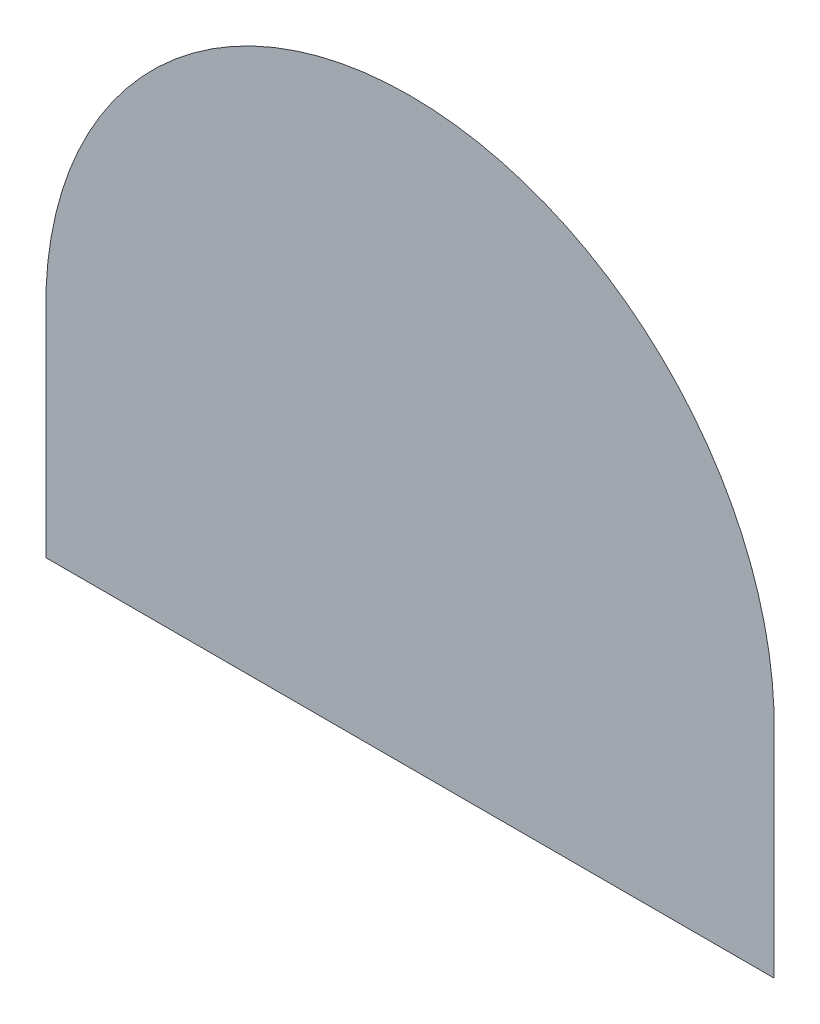
SolidWorks part; units mm, degrees
ref_plane "Plan de face" through (0, 0, 0) normal (0, 0, 1) x (1, 0, 0)
ref_plane "Plan de dessus" through (0, 0, 0) normal (0, 1, 0) x (1, 0, 0)
ref_plane "Plan de droite" through (0, 0, 0) normal (1, 0, 0) x (0, 0, -1)
sketch "Esquisse1" plane through (0, 0, 0) normal (0, 0, 1) x (1, 0, 0)
  line L6 (5, 0) -> (5, 77)
  line L8 (245, 0) -> (245, 77)
  line L14 (0, 0) -> (5, 0) construction
  line L16 (5, 0) -> (245, 0)
  line L19 (125, 192) -> (125, 197) construction
  arc A3 (245, 77) -> (5, 77) centre (125, 71.8913) ccw
  dimension "D4" = 120.1087
  dimension "D1" = 5
  dimension "D2" = 77
  dimension "D3" = 240
  dimension "D5" = 115
extrude "Boss.-Extru.1" add sketch "Esquisse1" along normal blind 0.0001 contours A3 L6 L16 L8
sketch "Esquisse2" plane through (0, 0, 0.0001) normal (0, 0, 1) x (1, 0, 0)
  line L0 (247.8787, -7.8787) -> (250, -10)
  line L1 (247.8787, -7.8787) -> (250, -5.7574)
  line L2 (250, -10) -> (252.1213, -7.8787)
  line L3 (250, -5.7574) -> (252.1213, -7.8787)
  line L4 (5, 0) -> (245, 0) construction
  line L5 (242.8787, -7.8787) -> (245, -10)
  line L6 (242.8787, -7.8787) -> (245, -5.7574)
  line L7 (245, -10) -> (247.1213, -7.8787)
  line L8 (245, -5.7574) -> (247.1213, -7.8787)
  line L9 (237.8787, -7.8787) -> (240, -10)
  line L10 (237.8787, -7.8787) -> (240, -5.7574)
  line L11 (240, -10) -> (242.1213, -7.8787)
  line L12 (240, -5.7574) -> (242.1213, -7.8787)
  line L13 (232.8787, -7.8787) -> (235, -10)
  line L14 (232.8787, -7.8787) -> (235, -5.7574)
  line L15 (235, -10) -> (237.1213, -7.8787)
  line L16 (235, -5.7574) -> (237.1213, -7.8787)
  line L17 (227.8787, -7.8787) -> (230, -10)
  line L18 (227.8787, -7.8787) -> (230, -5.7574)
  line L19 (230, -10) -> (232.1213, -7.8787)
  line L20 (230, -5.7574) -> (232.1213, -7.8787)
  line L21 (222.8787, -7.8787) -> (225, -10)
  line L22 (222.8787, -7.8787) -> (225, -5.7574)
  line L23 (225, -10) -> (227.1213, -7.8787)
  line L24 (225, -5.7574) -> (227.1213, -7.8787)
  line L25 (217.8787, -7.8787) -> (220, -10)
  line L26 (217.8787, -7.8787) -> (220, -5.7574)
  line L27 (220, -10) -> (222.1213, -7.8787)
  line L28 (220, -5.7574) -> (222.1213, -7.8787)
  line L29 (212.8787, -7.8787) -> (215, -10)
  line L30 (212.8787, -7.8787) -> (215, -5.7574)
  line L31 (215, -10) -> (217.1213, -7.8787)
  line L32 (215, -5.7574) -> (217.1213, -7.8787)
  line L33 (207.8787, -7.8787) -> (210, -10)
  line L34 (207.8787, -7.8787) -> (210, -5.7574)
  line L35 (210, -10) -> (212.1213, -7.8787)
  line L36 (210, -5.7574) -> (212.1213, -7.8787)
  line L37 (202.8787, -7.8787) -> (205, -10)
  line L38 (202.8787, -7.8787) -> (205, -5.7574)
  line L39 (205, -10) -> (207.1213, -7.8787)
  line L40 (205, -5.7574) -> (207.1213, -7.8787)
  line L41 (197.8787, -7.8787) -> (200, -10)
  line L42 (197.8787, -7.8787) -> (200, -5.7574)
  line L43 (200, -10) -> (202.1213, -7.8787)
  line L44 (200, -5.7574) -> (202.1213, -7.8787)
  line L45 (192.8787, -7.8787) -> (195, -10)
  line L46 (192.8787, -7.8787) -> (195, -5.7574)
  line L47 (195, -10) -> (197.1213, -7.8787)
  line L48 (195, -5.7574) -> (197.1213, -7.8787)
  line L49 (187.8787, -7.8787) -> (190, -10)
  line L50 (187.8787, -7.8787) -> (190, -5.7574)
  line L51 (190, -10) -> (192.1213, -7.8787)
  line L52 (190, -5.7574) -> (192.1213, -7.8787)
  line L53 (182.8787, -7.8787) -> (185, -10)
  line L54 (182.8787, -7.8787) -> (185, -5.7574)
  line L55 (185, -10) -> (187.1213, -7.8787)
  line L56 (185, -5.7574) -> (187.1213, -7.8787)
  line L57 (177.8787, -7.8787) -> (180, -10)
  line L58 (177.8787, -7.8787) -> (180, -5.7574)
  line L59 (180, -10) -> (182.1213, -7.8787)
  line L60 (180, -5.7574) -> (182.1213, -7.8787)
  line L61 (172.8787, -7.8787) -> (175, -10)
  line L62 (172.8787, -7.8787) -> (175, -5.7574)
  line L63 (175, -10) -> (177.1213, -7.8787)
  line L64 (175, -5.7574) -> (177.1213, -7.8787)
  line L65 (167.8787, -7.8787) -> (170, -10)
  line L66 (167.8787, -7.8787) -> (170, -5.7574)
  line L67 (170, -10) -> (172.1213, -7.8787)
  line L68 (170, -5.7574) -> (172.1213, -7.8787)
  line L69 (162.8787, -7.8787) -> (165, -10)
  line L70 (162.8787, -7.8787) -> (165, -5.7574)
  line L71 (165, -10) -> (167.1213, -7.8787)
  line L72 (165, -5.7574) -> (167.1213, -7.8787)
  line L73 (157.8787, -7.8787) -> (160, -10)
  line L74 (157.8787, -7.8787) -> (160, -5.7574)
  line L75 (160, -10) -> (162.1213, -7.8787)
  line L76 (160, -5.7574) -> (162.1213, -7.8787)
  line L77 (152.8787, -7.8787) -> (155, -10)
  line L78 (152.8787, -7.8787) -> (155, -5.7574)
  line L79 (155, -10) -> (157.1213, -7.8787)
  line L80 (155, -5.7574) -> (157.1213, -7.8787)
  line L81 (147.8787, -7.8787) -> (150, -10)
  line L82 (147.8787, -7.8787) -> (150, -5.7574)
  line L83 (150, -10) -> (152.1213, -7.8787)
  line L84 (150, -5.7574) -> (152.1213, -7.8787)
  line L85 (142.8787, -7.8787) -> (145, -10)
  line L86 (142.8787, -7.8787) -> (145, -5.7574)
  line L87 (145, -10) -> (147.1213, -7.8787)
  line L88 (145, -5.7574) -> (147.1213, -7.8787)
  line L89 (137.8787, -7.8787) -> (140, -10)
  line L90 (137.8787, -7.8787) -> (140, -5.7574)
  line L91 (140, -10) -> (142.1213, -7.8787)
  line L92 (140, -5.7574) -> (142.1213, -7.8787)
  line L93 (132.8787, -7.8787) -> (135, -10)
  line L94 (132.8787, -7.8787) -> (135, -5.7574)
  line L95 (135, -10) -> (137.1213, -7.8787)
  line L96 (135, -5.7574) -> (137.1213, -7.8787)
  line L97 (127.8787, -7.8787) -> (130, -10)
  line L98 (127.8787, -7.8787) -> (130, -5.7574)
  line L99 (130, -10) -> (132.1213, -7.8787)
  line L100 (130, -5.7574) -> (132.1213, -7.8787)
  line L101 (122.8787, -7.8787) -> (125, -10)
  line L102 (122.8787, -7.8787) -> (125, -5.7574)
  line L103 (125, -10) -> (127.1213, -7.8787)
  line L104 (125, -5.7574) -> (127.1213, -7.8787)
  line L105 (117.8787, -7.8787) -> (120, -10)
  line L106 (117.8787, -7.8787) -> (120, -5.7574)
  line L107 (120, -10) -> (122.1213, -7.8787)
  line L108 (120, -5.7574) -> (122.1213, -7.8787)
  line L109 (112.8787, -7.8787) -> (115, -10)
  line L110 (112.8787, -7.8787) -> (115, -5.7574)
  line L111 (115, -10) -> (117.1213, -7.8787)
  line L112 (115, -5.7574) -> (117.1213, -7.8787)
  line L113 (107.8787, -7.8787) -> (110, -10)
  line L114 (107.8787, -7.8787) -> (110, -5.7574)
  line L115 (110, -10) -> (112.1213, -7.8787)
  line L116 (110, -5.7574) -> (112.1213, -7.8787)
  line L117 (102.8787, -7.8787) -> (105, -10)
  line L118 (102.8787, -7.8787) -> (105, -5.7574)
  line L119 (105, -10) -> (107.1213, -7.8787)
  line L120 (105, -5.7574) -> (107.1213, -7.8787)
  line L121 (97.8787, -7.8787) -> (100, -10)
  line L122 (97.8787, -7.8787) -> (100, -5.7574)
  line L123 (100, -10) -> (102.1213, -7.8787)
  line L124 (100, -5.7574) -> (102.1213, -7.8787)
  line L125 (92.8787, -7.8787) -> (95, -10)
  line L126 (92.8787, -7.8787) -> (95, -5.7574)
  line L127 (95, -10) -> (97.1213, -7.8787)
  line L128 (95, -5.7574) -> (97.1213, -7.8787)
  line L129 (87.8787, -7.8787) -> (90, -10)
  line L130 (87.8787, -7.8787) -> (90, -5.7574)
  line L131 (90, -10) -> (92.1213, -7.8787)
  line L132 (90, -5.7574) -> (92.1213, -7.8787)
  line L133 (82.8787, -7.8787) -> (85, -10)
  line L134 (82.8787, -7.8787) -> (85, -5.7574)
  line L135 (85, -10) -> (87.1213, -7.8787)
  line L136 (85, -5.7574) -> (87.1213, -7.8787)
  line L137 (77.8787, -7.8787) -> (80, -10)
  line L138 (77.8787, -7.8787) -> (80, -5.7574)
  line L139 (80, -10) -> (82.1213, -7.8787)
  line L140 (80, -5.7574) -> (82.1213, -7.8787)
  line L141 (72.8787, -7.8787) -> (75, -10)
  line L142 (72.8787, -7.8787) -> (75, -5.7574)
  line L143 (75, -10) -> (77.1213, -7.8787)
  line L144 (75, -5.7574) -> (77.1213, -7.8787)
  line L145 (67.8787, -7.8787) -> (70, -10)
  line L146 (67.8787, -7.8787) -> (70, -5.7574)
  line L147 (70, -10) -> (72.1213, -7.8787)
  line L148 (70, -5.7574) -> (72.1213, -7.8787)
  line L149 (62.8787, -7.8787) -> (65, -10)
  line L150 (62.8787, -7.8787) -> (65, -5.7574)
  line L151 (65, -10) -> (67.1213, -7.8787)
  line L152 (65, -5.7574) -> (67.1213, -7.8787)
  line L153 (57.8787, -7.8787) -> (60, -10)
  line L154 (57.8787, -7.8787) -> (60, -5.7574)
  line L155 (60, -10) -> (62.1213, -7.8787)
  line L156 (60, -5.7574) -> (62.1213, -7.8787)
  line L157 (52.8787, -7.8787) -> (55, -10)
  line L158 (52.8787, -7.8787) -> (55, -5.7574)
  line L159 (55, -10) -> (57.1213, -7.8787)
  line L160 (55, -5.7574) -> (57.1213, -7.8787)
  line L161 (47.8787, -7.8787) -> (50, -10)
  line L162 (47.8787, -7.8787) -> (50, -5.7574)
  line L163 (50, -10) -> (52.1213, -7.8787)
  line L164 (50, -5.7574) -> (52.1213, -7.8787)
  line L165 (42.8787, -7.8787) -> (45, -10)
  line L166 (42.8787, -7.8787) -> (45, -5.7574)
  line L167 (45, -10) -> (47.1213, -7.8787)
  line L168 (45, -5.7574) -> (47.1213, -7.8787)
  line L169 (37.8787, -7.8787) -> (40, -10)
  line L170 (37.8787, -7.8787) -> (40, -5.7574)
  line L171 (40, -10) -> (42.1213, -7.8787)
  line L172 (40, -5.7574) -> (42.1213, -7.8787)
  line L173 (32.8787, -7.8787) -> (35, -10)
  line L174 (32.8787, -7.8787) -> (35, -5.7574)
  line L175 (35, -10) -> (37.1213, -7.8787)
  line L176 (35, -5.7574) -> (37.1213, -7.8787)
  line L177 (27.8787, -7.8787) -> (30, -10)
  line L178 (27.8787, -7.8787) -> (30, -5.7574)
  line L179 (30, -10) -> (32.1213, -7.8787)
  line L180 (30, -5.7574) -> (32.1213, -7.8787)
  line L181 (22.8787, -7.8787) -> (25, -10)
  line L182 (22.8787, -7.8787) -> (25, -5.7574)
  line L183 (25, -10) -> (27.1213, -7.8787)
  line L184 (25, -5.7574) -> (27.1213, -7.8787)
  line L185 (17.8787, -7.8787) -> (20, -10)
  line L186 (17.8787, -7.8787) -> (20, -5.7574)
  line L187 (20, -10) -> (22.1213, -7.8787)
  line L188 (20, -5.7574) -> (22.1213, -7.8787)
  line L189 (12.8787, -7.8787) -> (15, -10)
  line L190 (12.8787, -7.8787) -> (15, -5.7574)
  line L191 (15, -10) -> (17.1213, -7.8787)
  line L192 (15, -5.7574) -> (17.1213, -7.8787)
  line L193 (7.8787, -7.8787) -> (10, -10)
  line L194 (7.8787, -7.8787) -> (10, -5.7574)
  line L195 (10, -10) -> (12.1213, -7.8787)
  line L196 (10, -5.7574) -> (12.1213, -7.8787)
  line L197 (2.8787, -7.8787) -> (5, -10)
  line L198 (2.8787, -7.8787) -> (5, -5.7574)
  line L199 (5, -10) -> (7.1213, -7.8787)
  line L200 (5, -5.7574) -> (7.1213, -7.8787)
  line L201 (242.8787, -2.8787) -> (245, -5)
  line L202 (242.8787, -2.8787) -> (245, -0.7574)
  line L203 (245, -5) -> (247.1213, -2.8787)
  line L204 (245, -0.7574) -> (247.1213, -2.8787)
  line L205 (237.8787, -2.8787) -> (240, -5)
  line L206 (237.8787, -2.8787) -> (240, -0.7574)
  line L207 (240, -5) -> (242.1213, -2.8787)
  line L208 (240, -0.7574) -> (242.1213, -2.8787)
  line L209 (232.8787, -2.8787) -> (235, -5)
  line L210 (232.8787, -2.8787) -> (235, -0.7574)
  line L211 (235, -5) -> (237.1213, -2.8787)
  line L212 (235, -0.7574) -> (237.1213, -2.8787)
  line L213 (227.8787, -2.8787) -> (230, -5)
  line L214 (227.8787, -2.8787) -> (230, -0.7574)
  line L215 (230, -5) -> (232.1213, -2.8787)
  line L216 (230, -0.7574) -> (232.1213, -2.8787)
  line L217 (222.8787, -2.8787) -> (225, -5)
  line L218 (222.8787, -2.8787) -> (225, -0.7574)
  line L219 (225, -5) -> (227.1213, -2.8787)
  line L220 (225, -0.7574) -> (227.1213, -2.8787)
  line L221 (217.8787, -2.8787) -> (220, -5)
  line L222 (217.8787, -2.8787) -> (220, -0.7574)
  line L223 (220, -5) -> (222.1213, -2.8787)
  line L224 (220, -0.7574) -> (222.1213, -2.8787)
  line L225 (212.8787, -2.8787) -> (215, -5)
  line L226 (212.8787, -2.8787) -> (215, -0.7574)
  line L227 (215, -5) -> (217.1213, -2.8787)
  line L228 (215, -0.7574) -> (217.1213, -2.8787)
  line L229 (207.8787, -2.8787) -> (210, -5)
  line L230 (207.8787, -2.8787) -> (210, -0.7574)
  line L231 (210, -5) -> (212.1213, -2.8787)
  line L232 (210, -0.7574) -> (212.1213, -2.8787)
  line L233 (202.8787, -2.8787) -> (205, -5)
  line L234 (202.8787, -2.8787) -> (205, -0.7574)
  line L235 (205, -5) -> (207.1213, -2.8787)
  line L236 (205, -0.7574) -> (207.1213, -2.8787)
  line L237 (197.8787, -2.8787) -> (200, -5)
  line L238 (197.8787, -2.8787) -> (200, -0.7574)
  line L239 (200, -5) -> (202.1213, -2.8787)
  line L240 (200, -0.7574) -> (202.1213, -2.8787)
  line L241 (192.8787, -2.8787) -> (195, -5)
  line L242 (192.8787, -2.8787) -> (195, -0.7574)
  line L243 (195, -5) -> (197.1213, -2.8787)
  line L244 (195, -0.7574) -> (197.1213, -2.8787)
  line L245 (187.8787, -2.8787) -> (190, -5)
  line L246 (187.8787, -2.8787) -> (190, -0.7574)
  line L247 (190, -5) -> (192.1213, -2.8787)
  line L248 (190, -0.7574) -> (192.1213, -2.8787)
  line L249 (182.8787, -2.8787) -> (185, -5)
  line L250 (182.8787, -2.8787) -> (185, -0.7574)
  line L251 (185, -5) -> (187.1213, -2.8787)
  line L252 (185, -0.7574) -> (187.1213, -2.8787)
  line L253 (177.8787, -2.8787) -> (180, -5)
  line L254 (177.8787, -2.8787) -> (180, -0.7574)
  line L255 (180, -5) -> (182.1213, -2.8787)
  line L256 (180, -0.7574) -> (182.1213, -2.8787)
  line L257 (172.8787, -2.8787) -> (175, -5)
  line L258 (172.8787, -2.8787) -> (175, -0.7574)
  line L259 (175, -5) -> (177.1213, -2.8787)
  line L260 (175, -0.7574) -> (177.1213, -2.8787)
  line L261 (167.8787, -2.8787) -> (170, -5)
  line L262 (167.8787, -2.8787) -> (170, -0.7574)
  line L263 (170, -5) -> (172.1213, -2.8787)
  line L264 (170, -0.7574) -> (172.1213, -2.8787)
  line L265 (162.8787, -2.8787) -> (165, -5)
  line L266 (162.8787, -2.8787) -> (165, -0.7574)
  line L267 (165, -5) -> (167.1213, -2.8787)
  line L268 (165, -0.7574) -> (167.1213, -2.8787)
  line L269 (157.8787, -2.8787) -> (160, -5)
  line L270 (157.8787, -2.8787) -> (160, -0.7574)
  line L271 (160, -5) -> (162.1213, -2.8787)
  line L272 (160, -0.7574) -> (162.1213, -2.8787)
  line L273 (152.8787, -2.8787) -> (155, -5)
  line L274 (152.8787, -2.8787) -> (155, -0.7574)
  line L275 (155, -5) -> (157.1213, -2.8787)
  line L276 (155, -0.7574) -> (157.1213, -2.8787)
  line L277 (147.8787, -2.8787) -> (150, -5)
  line L278 (147.8787, -2.8787) -> (150, -0.7574)
  line L279 (150, -5) -> (152.1213, -2.8787)
  line L280 (150, -0.7574) -> (152.1213, -2.8787)
  line L281 (142.8787, -2.8787) -> (145, -5)
  line L282 (142.8787, -2.8787) -> (145, -0.7574)
  line L283 (145, -5) -> (147.1213, -2.8787)
  line L284 (145, -0.7574) -> (147.1213, -2.8787)
  line L285 (137.8787, -2.8787) -> (140, -5)
  line L286 (137.8787, -2.8787) -> (140, -0.7574)
  line L287 (140, -5) -> (142.1213, -2.8787)
  line L288 (140, -0.7574) -> (142.1213, -2.8787)
  line L289 (132.8787, -2.8787) -> (135, -5)
  line L290 (132.8787, -2.8787) -> (135, -0.7574)
  line L291 (135, -5) -> (137.1213, -2.8787)
  line L292 (135, -0.7574) -> (137.1213, -2.8787)
  line L293 (127.8787, -2.8787) -> (130, -5)
  line L294 (127.8787, -2.8787) -> (130, -0.7574)
  line L295 (130, -5) -> (132.1213, -2.8787)
  line L296 (130, -0.7574) -> (132.1213, -2.8787)
  line L297 (122.8787, -2.8787) -> (125, -5)
  line L298 (122.8787, -2.8787) -> (125, -0.7574)
  line L299 (125, -5) -> (127.1213, -2.8787)
  line L300 (125, -0.7574) -> (127.1213, -2.8787)
  line L301 (117.8787, -2.8787) -> (120, -5)
  line L302 (117.8787, -2.8787) -> (120, -0.7574)
  line L303 (120, -5) -> (122.1213, -2.8787)
  line L304 (120, -0.7574) -> (122.1213, -2.8787)
  line L305 (112.8787, -2.8787) -> (115, -5)
  line L306 (112.8787, -2.8787) -> (115, -0.7574)
  line L307 (115, -5) -> (117.1213, -2.8787)
  line L308 (115, -0.7574) -> (117.1213, -2.8787)
  line L309 (107.8787, -2.8787) -> (110, -5)
  line L310 (107.8787, -2.8787) -> (110, -0.7574)
  line L311 (110, -5) -> (112.1213, -2.8787)
  line L312 (110, -0.7574) -> (112.1213, -2.8787)
  line L313 (102.8787, -2.8787) -> (105, -5)
  line L314 (102.8787, -2.8787) -> (105, -0.7574)
  line L315 (105, -5) -> (107.1213, -2.8787)
  line L316 (105, -0.7574) -> (107.1213, -2.8787)
  line L317 (97.8787, -2.8787) -> (100, -5)
  line L318 (97.8787, -2.8787) -> (100, -0.7574)
  line L319 (100, -5) -> (102.1213, -2.8787)
  line L320 (100, -0.7574) -> (102.1213, -2.8787)
  line L321 (92.8787, -2.8787) -> (95, -5)
  line L322 (92.8787, -2.8787) -> (95, -0.7574)
  line L323 (95, -5) -> (97.1213, -2.8787)
  line L324 (95, -0.7574) -> (97.1213, -2.8787)
  line L325 (87.8787, -2.8787) -> (90, -5)
  line L326 (87.8787, -2.8787) -> (90, -0.7574)
  line L327 (90, -5) -> (92.1213, -2.8787)
  line L328 (90, -0.7574) -> (92.1213, -2.8787)
  line L329 (82.8787, -2.8787) -> (85, -5)
  line L330 (82.8787, -2.8787) -> (85, -0.7574)
  line L331 (85, -5) -> (87.1213, -2.8787)
  line L332 (85, -0.7574) -> (87.1213, -2.8787)
  line L333 (77.8787, -2.8787) -> (80, -5)
  line L334 (77.8787, -2.8787) -> (80, -0.7574)
  line L335 (80, -5) -> (82.1213, -2.8787)
  line L336 (80, -0.7574) -> (82.1213, -2.8787)
  line L337 (72.8787, -2.8787) -> (75, -5)
  line L338 (72.8787, -2.8787) -> (75, -0.7574)
  line L339 (75, -5) -> (77.1213, -2.8787)
  line L340 (75, -0.7574) -> (77.1213, -2.8787)
  line L341 (67.8787, -2.8787) -> (70, -5)
  line L342 (67.8787, -2.8787) -> (70, -0.7574)
  line L343 (70, -5) -> (72.1213, -2.8787)
  line L344 (70, -0.7574) -> (72.1213, -2.8787)
  line L345 (62.8787, -2.8787) -> (65, -5)
  line L346 (62.8787, -2.8787) -> (65, -0.7574)
  line L347 (65, -5) -> (67.1213, -2.8787)
  line L348 (65, -0.7574) -> (67.1213, -2.8787)
  line L349 (57.8787, -2.8787) -> (60, -5)
  line L350 (57.8787, -2.8787) -> (60, -0.7574)
  line L351 (60, -5) -> (62.1213, -2.8787)
  line L352 (60, -0.7574) -> (62.1213, -2.8787)
  line L353 (52.8787, -2.8787) -> (55, -5)
  line L354 (52.8787, -2.8787) -> (55, -0.7574)
  line L355 (55, -5) -> (57.1213, -2.8787)
  line L356 (55, -0.7574) -> (57.1213, -2.8787)
  line L357 (47.8787, -2.8787) -> (50, -5)
  line L358 (47.8787, -2.8787) -> (50, -0.7574)
  line L359 (50, -5) -> (52.1213, -2.8787)
  line L360 (50, -0.7574) -> (52.1213, -2.8787)
  line L361 (42.8787, -2.8787) -> (45, -5)
  line L362 (42.8787, -2.8787) -> (45, -0.7574)
  line L363 (45, -5) -> (47.1213, -2.8787)
  line L364 (45, -0.7574) -> (47.1213, -2.8787)
  line L365 (37.8787, -2.8787) -> (40, -5)
  line L366 (37.8787, -2.8787) -> (40, -0.7574)
  line L367 (40, -5) -> (42.1213, -2.8787)
  line L368 (40, -0.7574) -> (42.1213, -2.8787)
  line L369 (32.8787, -2.8787) -> (35, -5)
  line L370 (32.8787, -2.8787) -> (35, -0.7574)
  line L371 (35, -5) -> (37.1213, -2.8787)
  line L372 (35, -0.7574) -> (37.1213, -2.8787)
  line L373 (27.8787, -2.8787) -> (30, -5)
  line L374 (27.8787, -2.8787) -> (30, -0.7574)
  line L375 (30, -5) -> (32.1213, -2.8787)
  line L376 (30, -0.7574) -> (32.1213, -2.8787)
  line L377 (22.8787, -2.8787) -> (25, -5)
  line L378 (22.8787, -2.8787) -> (25, -0.7574)
  line L379 (25, -5) -> (27.1213, -2.8787)
  line L380 (25, -0.7574) -> (27.1213, -2.8787)
  line L381 (17.8787, -2.8787) -> (20, -5)
  line L382 (17.8787, -2.8787) -> (20, -0.7574)
  line L383 (20, -5) -> (22.1213, -2.8787)
  line L384 (20, -0.7574) -> (22.1213, -2.8787)
  line L385 (12.8787, -2.8787) -> (15, -5)
  line L386 (12.8787, -2.8787) -> (15, -0.7574)
  line L387 (15, -5) -> (17.1213, -2.8787)
  line L388 (15, -0.7574) -> (17.1213, -2.8787)
  line L389 (7.8787, -2.8787) -> (10, -5)
  line L390 (7.8787, -2.8787) -> (10, -0.7574)
  line L391 (10, -5) -> (12.1213, -2.8787)
  line L392 (10, -0.7574) -> (12.1213, -2.8787)
  line L393 (2.8787, -2.8787) -> (5, -5)
  line L394 (2.8787, -2.8787) -> (5, -0.7574)
  line L395 (5, -5) -> (7.1213, -2.8787)
  line L396 (5, -0.7574) -> (7.1213, -2.8787)
  line L397 (242.8787, 2.1213) -> (245, 0)
  line L398 (242.8787, 2.1213) -> (245, 4.2426)
  line L399 (245, 0) -> (247.1213, 2.1213)
  line L400 (245, 4.2426) -> (247.1213, 2.1213)
  line L401 (237.8787, 2.1213) -> (240, 0)
  line L402 (237.8787, 2.1213) -> (240, 4.2426)
  line L403 (240, 0) -> (242.1213, 2.1213)
  line L404 (240, 4.2426) -> (242.1213, 2.1213)
  line L405 (232.8787, 2.1213) -> (235, 0)
  line L406 (232.8787, 2.1213) -> (235, 4.2426)
  line L407 (235, 0) -> (237.1213, 2.1213)
  line L408 (235, 4.2426) -> (237.1213, 2.1213)
  line L409 (227.8787, 2.1213) -> (230, 0)
  line L410 (227.8787, 2.1213) -> (230, 4.2426)
  line L411 (230, 0) -> (232.1213, 2.1213)
  line L412 (230, 4.2426) -> (232.1213, 2.1213)
  line L413 (222.8787, 2.1213) -> (225, 0)
  line L414 (222.8787, 2.1213) -> (225, 4.2426)
  line L415 (225, 0) -> (227.1213, 2.1213)
  line L416 (225, 4.2426) -> (227.1213, 2.1213)
  line L417 (217.8787, 2.1213) -> (220, 0)
  line L418 (217.8787, 2.1213) -> (220, 4.2426)
  line L419 (220, 0) -> (222.1213, 2.1213)
  line L420 (220, 4.2426) -> (222.1213, 2.1213)
  line L421 (212.8787, 2.1213) -> (215, 0)
  line L422 (212.8787, 2.1213) -> (215, 4.2426)
  line L423 (215, 0) -> (217.1213, 2.1213)
  line L424 (215, 4.2426) -> (217.1213, 2.1213)
  line L425 (207.8787, 2.1213) -> (210, 0)
  line L426 (207.8787, 2.1213) -> (210, 4.2426)
  line L427 (210, 0) -> (212.1213, 2.1213)
  line L428 (210, 4.2426) -> (212.1213, 2.1213)
  line L429 (202.8787, 2.1213) -> (205, 0)
  line L430 (202.8787, 2.1213) -> (205, 4.2426)
  line L431 (205, 0) -> (207.1213, 2.1213)
  line L432 (205, 4.2426) -> (207.1213, 2.1213)
  line L433 (197.8787, 2.1213) -> (200, 0)
  line L434 (197.8787, 2.1213) -> (200, 4.2426)
  line L435 (200, 0) -> (202.1213, 2.1213)
  line L436 (200, 4.2426) -> (202.1213, 2.1213)
  line L437 (192.8787, 2.1213) -> (195, 0)
  line L438 (192.8787, 2.1213) -> (195, 4.2426)
  line L439 (195, 0) -> (197.1213, 2.1213)
  line L440 (195, 4.2426) -> (197.1213, 2.1213)
  line L441 (187.8787, 2.1213) -> (190, 0)
  line L442 (187.8787, 2.1213) -> (190, 4.2426)
  line L443 (190, 0) -> (192.1213, 2.1213)
  line L444 (190, 4.2426) -> (192.1213, 2.1213)
  line L445 (182.8787, 2.1213) -> (185, 0)
  line L446 (182.8787, 2.1213) -> (185, 4.2426)
  line L447 (185, 0) -> (187.1213, 2.1213)
  line L448 (185, 4.2426) -> (187.1213, 2.1213)
  line L449 (177.8787, 2.1213) -> (180, 0)
  line L450 (177.8787, 2.1213) -> (180, 4.2426)
  line L451 (180, 0) -> (182.1213, 2.1213)
  line L452 (180, 4.2426) -> (182.1213, 2.1213)
  line L453 (172.8787, 2.1213) -> (175, 0)
  line L454 (172.8787, 2.1213) -> (175, 4.2426)
  line L455 (175, 0) -> (177.1213, 2.1213)
  line L456 (175, 4.2426) -> (177.1213, 2.1213)
  line L457 (167.8787, 2.1213) -> (170, 0)
  line L458 (167.8787, 2.1213) -> (170, 4.2426)
  line L459 (170, 0) -> (172.1213, 2.1213)
  line L460 (170, 4.2426) -> (172.1213, 2.1213)
  line L461 (162.8787, 2.1213) -> (165, 0)
  line L462 (162.8787, 2.1213) -> (165, 4.2426)
  line L463 (165, 0) -> (167.1213, 2.1213)
  line L464 (165, 4.2426) -> (167.1213, 2.1213)
  line L465 (157.8787, 2.1213) -> (160, 0)
  line L466 (157.8787, 2.1213) -> (160, 4.2426)
  line L467 (160, 0) -> (162.1213, 2.1213)
  line L468 (160, 4.2426) -> (162.1213, 2.1213)
  line L469 (152.8787, 2.1213) -> (155, 0)
  line L470 (152.8787, 2.1213) -> (155, 4.2426)
  line L471 (155, 0) -> (157.1213, 2.1213)
  line L472 (155, 4.2426) -> (157.1213, 2.1213)
  line L473 (147.8787, 2.1213) -> (150, 0)
  line L474 (147.8787, 2.1213) -> (150, 4.2426)
  line L475 (150, 0) -> (152.1213, 2.1213)
  line L476 (150, 4.2426) -> (152.1213, 2.1213)
  line L477 (142.8787, 2.1213) -> (145, 0)
  line L478 (142.8787, 2.1213) -> (145, 4.2426)
  line L479 (145, 0) -> (147.1213, 2.1213)
  line L480 (145, 4.2426) -> (147.1213, 2.1213)
  line L481 (137.8787, 2.1213) -> (140, 0)
  line L482 (137.8787, 2.1213) -> (140, 4.2426)
  line L483 (140, 0) -> (142.1213, 2.1213)
  line L484 (140, 4.2426) -> (142.1213, 2.1213)
  line L485 (132.8787, 2.1213) -> (135, 0)
  line L486 (132.8787, 2.1213) -> (135, 4.2426)
  line L487 (135, 0) -> (137.1213, 2.1213)
  line L488 (135, 4.2426) -> (137.1213, 2.1213)
  line L489 (127.8787, 2.1213) -> (130, 0)
  line L490 (127.8787, 2.1213) -> (130, 4.2426)
  line L491 (130, 0) -> (132.1213, 2.1213)
  line L492 (130, 4.2426) -> (132.1213, 2.1213)
  line L493 (122.8787, 2.1213) -> (125, 0)
  line L494 (122.8787, 2.1213) -> (125, 4.2426)
  line L495 (125, 0) -> (127.1213, 2.1213)
  line L496 (125, 4.2426) -> (127.1213, 2.1213)
  line L497 (117.8787, 2.1213) -> (120, 0)
  line L498 (117.8787, 2.1213) -> (120, 4.2426)
  line L499 (120, 0) -> (122.1213, 2.1213)
  line L500 (120, 4.2426) -> (122.1213, 2.1213)
  line L501 (112.8787, 2.1213) -> (115, 0)
  line L502 (112.8787, 2.1213) -> (115, 4.2426)
  line L503 (115, 0) -> (117.1213, 2.1213)
  line L504 (115, 4.2426) -> (117.1213, 2.1213)
  line L505 (107.8787, 2.1213) -> (110, 0)
  line L506 (107.8787, 2.1213) -> (110, 4.2426)
  line L507 (110, 0) -> (112.1213, 2.1213)
  line L508 (110, 4.2426) -> (112.1213, 2.1213)
  line L509 (102.8787, 2.1213) -> (105, 0)
  line L510 (102.8787, 2.1213) -> (105, 4.2426)
  line L511 (105, 0) -> (107.1213, 2.1213)
  line L512 (105, 4.2426) -> (107.1213, 2.1213)
  line L513 (97.8787, 2.1213) -> (100, 0)
  line L514 (97.8787, 2.1213) -> (100, 4.2426)
  line L515 (100, 0) -> (102.1213, 2.1213)
  line L516 (100, 4.2426) -> (102.1213, 2.1213)
  line L517 (92.8787, 2.1213) -> (95, 0)
  line L518 (92.8787, 2.1213) -> (95, 4.2426)
  line L519 (95, 0) -> (97.1213, 2.1213)
  line L520 (95, 4.2426) -> (97.1213, 2.1213)
  line L521 (87.8787, 2.1213) -> (90, 0)
  line L522 (87.8787, 2.1213) -> (90, 4.2426)
  line L523 (90, 0) -> (92.1213, 2.1213)
  line L524 (90, 4.2426) -> (92.1213, 2.1213)
  line L525 (82.8787, 2.1213) -> (85, 0)
  line L526 (82.8787, 2.1213) -> (85, 4.2426)
  line L527 (85, 0) -> (87.1213, 2.1213)
  line L528 (85, 4.2426) -> (87.1213, 2.1213)
  line L529 (77.8787, 2.1213) -> (80, 0)
  line L530 (77.8787, 2.1213) -> (80, 4.2426)
  line L531 (80, 0) -> (82.1213, 2.1213)
  line L532 (80, 4.2426) -> (82.1213, 2.1213)
  line L533 (72.8787, 2.1213) -> (75, 0)
  line L534 (72.8787, 2.1213) -> (75, 4.2426)
  line L535 (75, 0) -> (77.1213, 2.1213)
  line L536 (75, 4.2426) -> (77.1213, 2.1213)
  line L537 (67.8787, 2.1213) -> (70, 0)
  line L538 (67.8787, 2.1213) -> (70, 4.2426)
  line L539 (70, 0) -> (72.1213, 2.1213)
  line L540 (70, 4.2426) -> (72.1213, 2.1213)
  line L541 (62.8787, 2.1213) -> (65, 0)
  line L542 (62.8787, 2.1213) -> (65, 4.2426)
  line L543 (65, 0) -> (67.1213, 2.1213)
  line L544 (65, 4.2426) -> (67.1213, 2.1213)
  line L545 (57.8787, 2.1213) -> (60, 0)
  line L546 (57.8787, 2.1213) -> (60, 4.2426)
  line L547 (60, 0) -> (62.1213, 2.1213)
  line L548 (60, 4.2426) -> (62.1213, 2.1213)
  line L549 (52.8787, 2.1213) -> (55, 0)
  line L550 (52.8787, 2.1213) -> (55, 4.2426)
  line L551 (55, 0) -> (57.1213, 2.1213)
  line L552 (55, 4.2426) -> (57.1213, 2.1213)
  line L553 (47.8787, 2.1213) -> (50, 0)
  line L554 (47.8787, 2.1213) -> (50, 4.2426)
  line L555 (50, 0) -> (52.1213, 2.1213)
  line L556 (50, 4.2426) -> (52.1213, 2.1213)
  line L557 (42.8787, 2.1213) -> (45, 0)
  line L558 (42.8787, 2.1213) -> (45, 4.2426)
  line L559 (45, 0) -> (47.1213, 2.1213)
  line L560 (45, 4.2426) -> (47.1213, 2.1213)
  line L561 (37.8787, 2.1213) -> (40, 0)
  line L562 (37.8787, 2.1213) -> (40, 4.2426)
  line L563 (40, 0) -> (42.1213, 2.1213)
  line L564 (40, 4.2426) -> (42.1213, 2.1213)
  line L565 (32.8787, 2.1213) -> (35, 0)
  line L566 (32.8787, 2.1213) -> (35, 4.2426)
  line L567 (35, 0) -> (37.1213, 2.1213)
  line L568 (35, 4.2426) -> (37.1213, 2.1213)
  line L569 (27.8787, 2.1213) -> (30, 0)
  line L570 (27.8787, 2.1213) -> (30, 4.2426)
  line L571 (30, 0) -> (32.1213, 2.1213)
  line L572 (30, 4.2426) -> (32.1213, 2.1213)
  line L573 (22.8787, 2.1213) -> (25, 0)
  line L574 (22.8787, 2.1213) -> (25, 4.2426)
  line L575 (25, 0) -> (27.1213, 2.1213)
  line L576 (25, 4.2426) -> (27.1213, 2.1213)
  line L577 (17.8787, 2.1213) -> (20, 0)
  line L578 (17.8787, 2.1213) -> (20, 4.2426)
  line L579 (20, 0) -> (22.1213, 2.1213)
  line L580 (20, 4.2426) -> (22.1213, 2.1213)
  line L581 (12.8787, 2.1213) -> (15, 0)
  line L582 (12.8787, 2.1213) -> (15, 4.2426)
  line L583 (15, 0) -> (17.1213, 2.1213)
  line L584 (15, 4.2426) -> (17.1213, 2.1213)
  line L585 (7.8787, 2.1213) -> (10, 0)
  line L586 (7.8787, 2.1213) -> (10, 4.2426)
  line L587 (10, 0) -> (12.1213, 2.1213)
  line L588 (10, 4.2426) -> (12.1213, 2.1213)
  line L589 (2.8787, 2.1213) -> (5, 0)
  line L590 (2.8787, 2.1213) -> (5, 4.2426)
  line L591 (5, 0) -> (7.1213, 2.1213)
  line L592 (5, 4.2426) -> (7.1213, 2.1213)
  line L593 (242.8787, 7.1213) -> (245, 5)
  line L594 (242.8787, 7.1213) -> (245, 9.2426)
  line L595 (245, 5) -> (247.1213, 7.1213)
  line L596 (245, 9.2426) -> (247.1213, 7.1213)
  line L597 (237.8787, 7.1213) -> (240, 5)
  line L598 (237.8787, 7.1213) -> (240, 9.2426)
  line L599 (240, 5) -> (242.1213, 7.1213)
  line L600 (240, 9.2426) -> (242.1213, 7.1213)
  line L601 (232.8787, 7.1213) -> (235, 5)
  line L602 (232.8787, 7.1213) -> (235, 9.2426)
  line L603 (235, 5) -> (237.1213, 7.1213)
  line L604 (235, 9.2426) -> (237.1213, 7.1213)
  line L605 (227.8787, 7.1213) -> (230, 5)
  line L606 (227.8787, 7.1213) -> (230, 9.2426)
  line L607 (230, 5) -> (232.1213, 7.1213)
  line L608 (230, 9.2426) -> (232.1213, 7.1213)
  line L609 (222.8787, 7.1213) -> (225, 5)
  line L610 (222.8787, 7.1213) -> (225, 9.2426)
  line L611 (225, 5) -> (227.1213, 7.1213)
  line L612 (225, 9.2426) -> (227.1213, 7.1213)
  line L613 (217.8787, 7.1213) -> (220, 5)
  line L614 (217.8787, 7.1213) -> (220, 9.2426)
  line L615 (220, 5) -> (222.1213, 7.1213)
  line L616 (220, 9.2426) -> (222.1213, 7.1213)
  line L617 (212.8787, 7.1213) -> (215, 5)
  line L618 (212.8787, 7.1213) -> (215, 9.2426)
  line L619 (215, 5) -> (217.1213, 7.1213)
  line L620 (215, 9.2426) -> (217.1213, 7.1213)
  line L621 (207.8787, 7.1213) -> (210, 5)
  line L622 (207.8787, 7.1213) -> (210, 9.2426)
  line L623 (210, 5) -> (212.1213, 7.1213)
  line L624 (210, 9.2426) -> (212.1213, 7.1213)
  line L625 (202.8787, 7.1213) -> (205, 5)
  line L626 (202.8787, 7.1213) -> (205, 9.2426)
  line L627 (205, 5) -> (207.1213, 7.1213)
  line L628 (205, 9.2426) -> (207.1213, 7.1213)
  line L629 (197.8787, 7.1213) -> (200, 5)
  line L630 (197.8787, 7.1213) -> (200, 9.2426)
  line L631 (200, 5) -> (202.1213, 7.1213)
  line L632 (200, 9.2426) -> (202.1213, 7.1213)
  line L633 (192.8787, 7.1213) -> (195, 5)
  line L634 (192.8787, 7.1213) -> (195, 9.2426)
  line L635 (195, 5) -> (197.1213, 7.1213)
  line L636 (195, 9.2426) -> (197.1213, 7.1213)
  line L637 (187.8787, 7.1213) -> (190, 5)
  line L638 (187.8787, 7.1213) -> (190, 9.2426)
  line L639 (190, 5) -> (192.1213, 7.1213)
  line L640 (190, 9.2426) -> (192.1213, 7.1213)
  line L641 (182.8787, 7.1213) -> (185, 5)
  line L642 (182.8787, 7.1213) -> (185, 9.2426)
  line L643 (185, 5) -> (187.1213, 7.1213)
  line L644 (185, 9.2426) -> (187.1213, 7.1213)
  line L645 (177.8787, 7.1213) -> (180, 5)
  line L646 (177.8787, 7.1213) -> (180, 9.2426)
  line L647 (180, 5) -> (182.1213, 7.1213)
  line L648 (180, 9.2426) -> (182.1213, 7.1213)
  line L649 (172.8787, 7.1213) -> (175, 5)
  line L650 (172.8787, 7.1213) -> (175, 9.2426)
  line L651 (175, 5) -> (177.1213, 7.1213)
  line L652 (175, 9.2426) -> (177.1213, 7.1213)
  line L653 (167.8787, 7.1213) -> (170, 5)
  line L654 (167.8787, 7.1213) -> (170, 9.2426)
  line L655 (170, 5) -> (172.1213, 7.1213)
  line L656 (170, 9.2426) -> (172.1213, 7.1213)
  line L657 (162.8787, 7.1213) -> (165, 5)
  line L658 (162.8787, 7.1213) -> (165, 9.2426)
  line L659 (165, 5) -> (167.1213, 7.1213)
  line L660 (165, 9.2426) -> (167.1213, 7.1213)
  line L661 (157.8787, 7.1213) -> (160, 5)
  line L662 (157.8787, 7.1213) -> (160, 9.2426)
  line L663 (160, 5) -> (162.1213, 7.1213)
  line L664 (160, 9.2426) -> (162.1213, 7.1213)
  line L665 (152.8787, 7.1213) -> (155, 5)
  line L666 (152.8787, 7.1213) -> (155, 9.2426)
  line L667 (155, 5) -> (157.1213, 7.1213)
  line L668 (155, 9.2426) -> (157.1213, 7.1213)
  line L669 (147.8787, 7.1213) -> (150, 5)
  line L670 (147.8787, 7.1213) -> (150, 9.2426)
  line L671 (150, 5) -> (152.1213, 7.1213)
  line L672 (150, 9.2426) -> (152.1213, 7.1213)
  line L673 (142.8787, 7.1213) -> (145, 5)
  line L674 (142.8787, 7.1213) -> (145, 9.2426)
  line L675 (145, 5) -> (147.1213, 7.1213)
  line L676 (145, 9.2426) -> (147.1213, 7.1213)
  line L677 (137.8787, 7.1213) -> (140, 5)
  line L678 (137.8787, 7.1213) -> (140, 9.2426)
  line L679 (140, 5) -> (142.1213, 7.1213)
  line L680 (140, 9.2426) -> (142.1213, 7.1213)
  line L681 (132.8787, 7.1213) -> (135, 5)
  line L682 (132.8787, 7.1213) -> (135, 9.2426)
  line L683 (135, 5) -> (137.1213, 7.1213)
  line L684 (135, 9.2426) -> (137.1213, 7.1213)
  line L685 (127.8787, 7.1213) -> (130, 5)
  line L686 (127.8787, 7.1213) -> (130, 9.2426)
  line L687 (130, 5) -> (132.1213, 7.1213)
  line L688 (130, 9.2426) -> (132.1213, 7.1213)
  line L689 (122.8787, 7.1213) -> (125, 5)
  line L690 (122.8787, 7.1213) -> (125, 9.2426)
  line L691 (125, 5) -> (127.1213, 7.1213)
  line L692 (125, 9.2426) -> (127.1213, 7.1213)
  line L693 (117.8787, 7.1213) -> (120, 5)
  line L694 (117.8787, 7.1213) -> (120, 9.2426)
  line L695 (120, 5) -> (122.1213, 7.1213)
  line L696 (120, 9.2426) -> (122.1213, 7.1213)
  line L697 (112.8787, 7.1213) -> (115, 5)
  line L698 (112.8787, 7.1213) -> (115, 9.2426)
  line L699 (115, 5) -> (117.1213, 7.1213)
  line L700 (115, 9.2426) -> (117.1213, 7.1213)
  line L701 (107.8787, 7.1213) -> (110, 5)
  line L702 (107.8787, 7.1213) -> (110, 9.2426)
  line L703 (110, 5) -> (112.1213, 7.1213)
  line L704 (110, 9.2426) -> (112.1213, 7.1213)
  line L705 (102.8787, 7.1213) -> (105, 5)
  line L706 (102.8787, 7.1213) -> (105, 9.2426)
  line L707 (105, 5) -> (107.1213, 7.1213)
  line L708 (105, 9.2426) -> (107.1213, 7.1213)
  line L709 (97.8787, 7.1213) -> (100, 5)
  line L710 (97.8787, 7.1213) -> (100, 9.2426)
  line L711 (100, 5) -> (102.1213, 7.1213)
  line L712 (100, 9.2426) -> (102.1213, 7.1213)
  line L713 (92.8787, 7.1213) -> (95, 5)
  line L714 (92.8787, 7.1213) -> (95, 9.2426)
  line L715 (95, 5) -> (97.1213, 7.1213)
  line L716 (95, 9.2426) -> (97.1213, 7.1213)
  line L717 (87.8787, 7.1213) -> (90, 5)
  line L718 (87.8787, 7.1213) -> (90, 9.2426)
  line L719 (90, 5) -> (92.1213, 7.1213)
  line L720 (90, 9.2426) -> (92.1213, 7.1213)
  line L721 (82.8787, 7.1213) -> (85, 5)
  line L722 (82.8787, 7.1213) -> (85, 9.2426)
  line L723 (85, 5) -> (87.1213, 7.1213)
  line L724 (85, 9.2426) -> (87.1213, 7.1213)
  line L725 (77.8787, 7.1213) -> (80, 5)
  line L726 (77.8787, 7.1213) -> (80, 9.2426)
  line L727 (80, 5) -> (82.1213, 7.1213)
  line L728 (80, 9.2426) -> (82.1213, 7.1213)
  line L729 (72.8787, 7.1213) -> (75, 5)
  line L730 (72.8787, 7.1213) -> (75, 9.2426)
  line L731 (75, 5) -> (77.1213, 7.1213)
  line L732 (75, 9.2426) -> (77.1213, 7.1213)
  line L733 (67.8787, 7.1213) -> (70, 5)
  line L734 (67.8787, 7.1213) -> (70, 9.2426)
  line L735 (70, 5) -> (72.1213, 7.1213)
  line L736 (70, 9.2426) -> (72.1213, 7.1213)
  line L737 (62.8787, 7.1213) -> (65, 5)
  line L738 (62.8787, 7.1213) -> (65, 9.2426)
  line L739 (65, 5) -> (67.1213, 7.1213)
  line L740 (65, 9.2426) -> (67.1213, 7.1213)
  line L741 (57.8787, 7.1213) -> (60, 5)
  line L742 (57.8787, 7.1213) -> (60, 9.2426)
  line L743 (60, 5) -> (62.1213, 7.1213)
  line L744 (60, 9.2426) -> (62.1213, 7.1213)
  line L745 (52.8787, 7.1213) -> (55, 5)
  line L746 (52.8787, 7.1213) -> (55, 9.2426)
  line L747 (55, 5) -> (57.1213, 7.1213)
  line L748 (55, 9.2426) -> (57.1213, 7.1213)
  line L749 (47.8787, 7.1213) -> (50, 5)
  line L750 (47.8787, 7.1213) -> (50, 9.2426)
  line L751 (50, 5) -> (52.1213, 7.1213)
  line L752 (50, 9.2426) -> (52.1213, 7.1213)
  line L753 (42.8787, 7.1213) -> (45, 5)
  line L754 (42.8787, 7.1213) -> (45, 9.2426)
  line L755 (45, 5) -> (47.1213, 7.1213)
  line L756 (45, 9.2426) -> (47.1213, 7.1213)
  line L757 (37.8787, 7.1213) -> (40, 5)
  line L758 (37.8787, 7.1213) -> (40, 9.2426)
  line L759 (40, 5) -> (42.1213, 7.1213)
  line L760 (40, 9.2426) -> (42.1213, 7.1213)
  line L761 (32.8787, 7.1213) -> (35, 5)
  line L762 (32.8787, 7.1213) -> (35, 9.2426)
  line L763 (35, 5) -> (37.1213, 7.1213)
  line L764 (35, 9.2426) -> (37.1213, 7.1213)
  line L765 (27.8787, 7.1213) -> (30, 5)
  line L766 (27.8787, 7.1213) -> (30, 9.2426)
  line L767 (30, 5) -> (32.1213, 7.1213)
  line L768 (30, 9.2426) -> (32.1213, 7.1213)
  line L769 (22.8787, 7.1213) -> (25, 5)
  line L770 (22.8787, 7.1213) -> (25, 9.2426)
  line L771 (25, 5) -> (27.1213, 7.1213)
  line L772 (25, 9.2426) -> (27.1213, 7.1213)
  line L773 (17.8787, 7.1213) -> (20, 5)
  line L774 (17.8787, 7.1213) -> (20, 9.2426)
  line L775 (20, 5) -> (22.1213, 7.1213)
  line L776 (20, 9.2426) -> (22.1213, 7.1213)
  line L777 (12.8787, 7.1213) -> (15, 5)
  line L778 (12.8787, 7.1213) -> (15, 9.2426)
  line L779 (15, 5) -> (17.1213, 7.1213)
  line L780 (15, 9.2426) -> (17.1213, 7.1213)
  line L781 (7.8787, 7.1213) -> (10, 5)
  line L782 (7.8787, 7.1213) -> (10, 9.2426)
  line L783 (10, 5) -> (12.1213, 7.1213)
  line L784 (10, 9.2426) -> (12.1213, 7.1213)
  line L785 (2.8787, 7.1213) -> (5, 5)
  line L786 (2.8787, 7.1213) -> (5, 9.2426)
  line L787 (5, 5) -> (7.1213, 7.1213)
  line L788 (5, 9.2426) -> (7.1213, 7.1213)
  line L789 (242.8787, 12.1213) -> (245, 10)
  line L790 (242.8787, 12.1213) -> (245, 14.2426)
  line L791 (245, 10) -> (247.1213, 12.1213)
  line L792 (245, 14.2426) -> (247.1213, 12.1213)
  line L793 (237.8787, 12.1213) -> (240, 10)
  line L794 (237.8787, 12.1213) -> (240, 14.2426)
  line L795 (240, 10) -> (242.1213, 12.1213)
  line L796 (240, 14.2426) -> (242.1213, 12.1213)
  line L797 (232.8787, 12.1213) -> (235, 10)
  line L798 (232.8787, 12.1213) -> (235, 14.2426)
  line L799 (235, 10) -> (237.1213, 12.1213)
  line L800 (235, 14.2426) -> (237.1213, 12.1213)
  line L801 (227.8787, 12.1213) -> (230, 10)
  line L802 (227.8787, 12.1213) -> (230, 14.2426)
  line L803 (230, 10) -> (232.1213, 12.1213)
  line L804 (230, 14.2426) -> (232.1213, 12.1213)
  line L805 (222.8787, 12.1213) -> (225, 10)
  line L806 (222.8787, 12.1213) -> (225, 14.2426)
  line L807 (225, 10) -> (227.1213, 12.1213)
  line L808 (225, 14.2426) -> (227.1213, 12.1213)
  line L809 (217.8787, 12.1213) -> (220, 10)
  line L810 (217.8787, 12.1213) -> (220, 14.2426)
  line L811 (220, 10) -> (222.1213, 12.1213)
  line L812 (220, 14.2426) -> (222.1213, 12.1213)
  line L813 (212.8787, 12.1213) -> (215, 10)
  line L814 (212.8787, 12.1213) -> (215, 14.2426)
  line L815 (215, 10) -> (217.1213, 12.1213)
  line L816 (215, 14.2426) -> (217.1213, 12.1213)
  line L817 (207.8787, 12.1213) -> (210, 10)
  line L818 (207.8787, 12.1213) -> (210, 14.2426)
  line L819 (210, 10) -> (212.1213, 12.1213)
  line L820 (210, 14.2426) -> (212.1213, 12.1213)
  line L821 (202.8787, 12.1213) -> (205, 10)
  line L822 (202.8787, 12.1213) -> (205, 14.2426)
  line L823 (205, 10) -> (207.1213, 12.1213)
  line L824 (205, 14.2426) -> (207.1213, 12.1213)
  line L825 (197.8787, 12.1213) -> (200, 10)
  line L826 (197.8787, 12.1213) -> (200, 14.2426)
  line L827 (200, 10) -> (202.1213, 12.1213)
  line L828 (200, 14.2426) -> (202.1213, 12.1213)
  line L829 (192.8787, 12.1213) -> (195, 10)
  line L830 (192.8787, 12.1213) -> (195, 14.2426)
  line L831 (195, 10) -> (197.1213, 12.1213)
  line L832 (195, 14.2426) -> (197.1213, 12.1213)
  line L833 (187.8787, 12.1213) -> (190, 10)
  line L834 (187.8787, 12.1213) -> (190, 14.2426)
  line L835 (190, 10) -> (192.1213, 12.1213)
  line L836 (190, 14.2426) -> (192.1213, 12.1213)
  line L837 (182.8787, 12.1213) -> (185, 10)
  line L838 (182.8787, 12.1213) -> (185, 14.2426)
  line L839 (185, 10) -> (187.1213, 12.1213)
  line L840 (185, 14.2426) -> (187.1213, 12.1213)
  line L841 (177.8787, 12.1213) -> (180, 10)
  line L842 (177.8787, 12.1213) -> (180, 14.2426)
  line L843 (180, 10) -> (182.1213, 12.1213)
  line L844 (180, 14.2426) -> (182.1213, 12.1213)
  line L845 (172.8787, 12.1213) -> (175, 10)
  line L846 (172.8787, 12.1213) -> (175, 14.2426)
  line L847 (175, 10) -> (177.1213, 12.1213)
  line L848 (175, 14.2426) -> (177.1213, 12.1213)
  line L849 (167.8787, 12.1213) -> (170, 10)
  line L850 (167.8787, 12.1213) -> (170, 14.2426)
  line L851 (170, 10) -> (172.1213, 12.1213)
  line L852 (170, 14.2426) -> (172.1213, 12.1213)
  line L853 (162.8787, 12.1213) -> (165, 10)
  line L854 (162.8787, 12.1213) -> (165, 14.2426)
  line L855 (165, 10) -> (167.1213, 12.1213)
  line L856 (165, 14.2426) -> (167.1213, 12.1213)
  line L857 (157.8787, 12.1213) -> (160, 10)
  line L858 (157.8787, 12.1213) -> (160, 14.2426)
  line L859 (160, 10) -> (162.1213, 12.1213)
  line L860 (160, 14.2426) -> (162.1213, 12.1213)
  line L861 (152.8787, 12.1213) -> (155, 10)
  line L862 (152.8787, 12.1213) -> (155, 14.2426)
  line L863 (155, 10) -> (157.1213, 12.1213)
  line L864 (155, 14.2426) -> (157.1213, 12.1213)
  line L865 (147.8787, 12.1213) -> (150, 10)
  line L866 (147.8787, 12.1213) -> (150, 14.2426)
  line L867 (150, 10) -> (152.1213, 12.1213)
  line L868 (150, 14.2426) -> (152.1213, 12.1213)
  line L869 (142.8787, 12.1213) -> (145, 10)
  line L870 (142.8787, 12.1213) -> (145, 14.2426)
  line L871 (145, 10) -> (147.1213, 12.1213)
  line L872 (145, 14.2426) -> (147.1213, 12.1213)
  line L873 (137.8787, 12.1213) -> (140, 10)
  line L874 (137.8787, 12.1213) -> (140, 14.2426)
  line L875 (140, 10) -> (142.1213, 12.1213)
  line L876 (140, 14.2426) -> (142.1213, 12.1213)
  line L877 (132.8787, 12.1213) -> (135, 10)
  line L878 (132.8787, 12.1213) -> (135, 14.2426)
  line L879 (135, 10) -> (137.1213, 12.1213)
  line L880 (135, 14.2426) -> (137.1213, 12.1213)
  line L881 (127.8787, 12.1213) -> (130, 10)
  line L882 (127.8787, 12.1213) -> (130, 14.2426)
  line L883 (130, 10) -> (132.1213, 12.1213)
  line L884 (130, 14.2426) -> (132.1213, 12.1213)
  line L885 (122.8787, 12.1213) -> (125, 10)
  line L886 (122.8787, 12.1213) -> (125, 14.2426)
  line L887 (125, 10) -> (127.1213, 12.1213)
  line L888 (125, 14.2426) -> (127.1213, 12.1213)
  line L889 (117.8787, 12.1213) -> (120, 10)
  line L890 (117.8787, 12.1213) -> (120, 14.2426)
  line L891 (120, 10) -> (122.1213, 12.1213)
  line L892 (120, 14.2426) -> (122.1213, 12.1213)
  line L893 (112.8787, 12.1213) -> (115, 10)
  line L894 (112.8787, 12.1213) -> (115, 14.2426)
  line L895 (115, 10) -> (117.1213, 12.1213)
  line L896 (115, 14.2426) -> (117.1213, 12.1213)
  line L897 (107.8787, 12.1213) -> (110, 10)
  line L898 (107.8787, 12.1213) -> (110, 14.2426)
  line L899 (110, 10) -> (112.1213, 12.1213)
  line L900 (110, 14.2426) -> (112.1213, 12.1213)
  line L901 (102.8787, 12.1213) -> (105, 10)
  line L902 (102.8787, 12.1213) -> (105, 14.2426)
  line L903 (105, 10) -> (107.1213, 12.1213)
  line L904 (105, 14.2426) -> (107.1213, 12.1213)
  line L905 (97.8787, 12.1213) -> (100, 10)
  line L906 (97.8787, 12.1213) -> (100, 14.2426)
  line L907 (100, 10) -> (102.1213, 12.1213)
  line L908 (100, 14.2426) -> (102.1213, 12.1213)
  line L909 (92.8787, 12.1213) -> (95, 10)
  line L910 (92.8787, 12.1213) -> (95, 14.2426)
  line L911 (95, 10) -> (97.1213, 12.1213)
  line L912 (95, 14.2426) -> (97.1213, 12.1213)
  line L913 (87.8787, 12.1213) -> (90, 10)
  line L914 (87.8787, 12.1213) -> (90, 14.2426)
  line L915 (90, 10) -> (92.1213, 12.1213)
  line L916 (90, 14.2426) -> (92.1213, 12.1213)
  line L917 (82.8787, 12.1213) -> (85, 10)
  line L918 (82.8787, 12.1213) -> (85, 14.2426)
  line L919 (85, 10) -> (87.1213, 12.1213)
  line L920 (85, 14.2426) -> (87.1213, 12.1213)
  line L921 (77.8787, 12.1213) -> (80, 10)
  line L922 (77.8787, 12.1213) -> (80, 14.2426)
  line L923 (80, 10) -> (82.1213, 12.1213)
  line L924 (80, 14.2426) -> (82.1213, 12.1213)
  line L925 (72.8787, 12.1213) -> (75, 10)
  line L926 (72.8787, 12.1213) -> (75, 14.2426)
  line L927 (75, 10) -> (77.1213, 12.1213)
  line L928 (75, 14.2426) -> (77.1213, 12.1213)
  line L929 (67.8787, 12.1213) -> (70, 10)
  line L930 (67.8787, 12.1213) -> (70, 14.2426)
  line L931 (70, 10) -> (72.1213, 12.1213)
  line L932 (70, 14.2426) -> (72.1213, 12.1213)
  line L933 (62.8787, 12.1213) -> (65, 10)
  line L934 (62.8787, 12.1213) -> (65, 14.2426)
  line L935 (65, 10) -> (67.1213, 12.1213)
  line L936 (65, 14.2426) -> (67.1213, 12.1213)
  line L937 (57.8787, 12.1213) -> (60, 10)
  line L938 (57.8787, 12.1213) -> (60, 14.2426)
  line L939 (60, 10) -> (62.1213, 12.1213)
  line L940 (60, 14.2426) -> (62.1213, 12.1213)
  line L941 (52.8787, 12.1213) -> (55, 10)
  line L942 (52.8787, 12.1213) -> (55, 14.2426)
  line L943 (55, 10) -> (57.1213, 12.1213)
  line L944 (55, 14.2426) -> (57.1213, 12.1213)
  line L945 (47.8787, 12.1213) -> (50, 10)
  line L946 (47.8787, 12.1213) -> (50, 14.2426)
  line L947 (50, 10) -> (52.1213, 12.1213)
  line L948 (50, 14.2426) -> (52.1213, 12.1213)
  line L949 (42.8787, 12.1213) -> (45, 10)
  line L950 (42.8787, 12.1213) -> (45, 14.2426)
  line L951 (45, 10) -> (47.1213, 12.1213)
  line L952 (45, 14.2426) -> (47.1213, 12.1213)
  line L953 (37.8787, 12.1213) -> (40, 10)
  line L954 (37.8787, 12.1213) -> (40, 14.2426)
  line L955 (40, 10) -> (42.1213, 12.1213)
  line L956 (40, 14.2426) -> (42.1213, 12.1213)
  line L957 (32.8787, 12.1213) -> (35, 10)
  line L958 (32.8787, 12.1213) -> (35, 14.2426)
  line L959 (35, 10) -> (37.1213, 12.1213)
  line L960 (35, 14.2426) -> (37.1213, 12.1213)
  line L961 (27.8787, 12.1213) -> (30, 10)
  line L962 (27.8787, 12.1213) -> (30, 14.2426)
  line L963 (30, 10) -> (32.1213, 12.1213)
  line L964 (30, 14.2426) -> (32.1213, 12.1213)
  line L965 (22.8787, 12.1213) -> (25, 10)
  line L966 (22.8787, 12.1213) -> (25, 14.2426)
  line L967 (25, 10) -> (27.1213, 12.1213)
  line L968 (25, 14.2426) -> (27.1213, 12.1213)
  line L969 (17.8787, 12.1213) -> (20, 10)
  line L970 (17.8787, 12.1213) -> (20, 14.2426)
  line L971 (20, 10) -> (22.1213, 12.1213)
  line L972 (20, 14.2426) -> (22.1213, 12.1213)
  line L973 (12.8787, 12.1213) -> (15, 10)
  line L974 (12.8787, 12.1213) -> (15, 14.2426)
  line L975 (15, 10) -> (17.1213, 12.1213)
  line L976 (15, 14.2426) -> (17.1213, 12.1213)
  line L977 (7.8787, 12.1213) -> (10, 10)
  line L978 (7.8787, 12.1213) -> (10, 14.2426)
  line L979 (10, 10) -> (12.1213, 12.1213)
  line L980 (10, 14.2426) -> (12.1213, 12.1213)
  line L981 (2.8787, 12.1213) -> (5, 10)
  line L982 (2.8787, 12.1213) -> (5, 14.2426)
  line L983 (5, 10) -> (7.1213, 12.1213)
  line L984 (5, 14.2426) -> (7.1213, 12.1213)
  line L985 (242.8787, 17.1213) -> (245, 15)
  line L986 (242.8787, 17.1213) -> (245, 19.2426)
  line L987 (245, 15) -> (247.1213, 17.1213)
  line L988 (245, 19.2426) -> (247.1213, 17.1213)
  line L989 (237.8787, 17.1213) -> (240, 15)
  line L990 (237.8787, 17.1213) -> (240, 19.2426)
  line L991 (240, 15) -> (242.1213, 17.1213)
  line L992 (240, 19.2426) -> (242.1213, 17.1213)
  line L993 (232.8787, 17.1213) -> (235, 15)
  line L994 (232.8787, 17.1213) -> (235, 19.2426)
  line L995 (235, 15) -> (237.1213, 17.1213)
  line L996 (235, 19.2426) -> (237.1213, 17.1213)
  line L997 (227.8787, 17.1213) -> (230, 15)
  line L998 (227.8787, 17.1213) -> (230, 19.2426)
  line L999 (230, 15) -> (232.1213, 17.1213)
  line L1000 (230, 19.2426) -> (232.1213, 17.1213)
  line L1001 (222.8787, 17.1213) -> (225, 15)
  line L1002 (222.8787, 17.1213) -> (225, 19.2426)
  line L1003 (225, 15) -> (227.1213, 17.1213)
  line L1004 (225, 19.2426) -> (227.1213, 17.1213)
  line L1005 (217.8787, 17.1213) -> (220, 15)
  line L1006 (217.8787, 17.1213) -> (220, 19.2426)
  line L1007 (220, 15) -> (222.1213, 17.1213)
  line L1008 (220, 19.2426) -> (222.1213, 17.1213)
  line L1009 (212.8787, 17.1213) -> (215, 15)
  line L1010 (212.8787, 17.1213) -> (215, 19.2426)
  line L1011 (215, 15) -> (217.1213, 17.1213)
  line L1012 (215, 19.2426) -> (217.1213, 17.1213)
  line L1013 (207.8787, 17.1213) -> (210, 15)
  line L1014 (207.8787, 17.1213) -> (210, 19.2426)
  line L1015 (210, 15) -> (212.1213, 17.1213)
  line L1016 (210, 19.2426) -> (212.1213, 17.1213)
  line L1017 (202.8787, 17.1213) -> (205, 15)
  line L1018 (202.8787, 17.1213) -> (205, 19.2426)
  line L1019 (205, 15) -> (207.1213, 17.1213)
  line L1020 (205, 19.2426) -> (207.1213, 17.1213)
  line L1021 (197.8787, 17.1213) -> (200, 15)
  line L1022 (197.8787, 17.1213) -> (200, 19.2426)
  line L1023 (200, 15) -> (202.1213, 17.1213)
  line L1024 (200, 19.2426) -> (202.1213, 17.1213)
  line L1025 (192.8787, 17.1213) -> (195, 15)
  line L1026 (192.8787, 17.1213) -> (195, 19.2426)
  line L1027 (195, 15) -> (197.1213, 17.1213)
  line L1028 (195, 19.2426) -> (197.1213, 17.1213)
  line L1029 (187.8787, 17.1213) -> (190, 15)
  line L1030 (187.8787, 17.1213) -> (190, 19.2426)
  line L1031 (190, 15) -> (192.1213, 17.1213)
  line L1032 (190, 19.2426) -> (192.1213, 17.1213)
  line L1033 (182.8787, 17.1213) -> (185, 15)
  line L1034 (182.8787, 17.1213) -> (185, 19.2426)
  line L1035 (185, 15) -> (187.1213, 17.1213)
  line L1036 (185, 19.2426) -> (187.1213, 17.1213)
  line L1037 (177.8787, 17.1213) -> (180, 15)
  line L1038 (177.8787, 17.1213) -> (180, 19.2426)
  line L1039 (180, 15) -> (182.1213, 17.1213)
  line L1040 (180, 19.2426) -> (182.1213, 17.1213)
  line L1041 (172.8787, 17.1213) -> (175, 15)
  line L1042 (172.8787, 17.1213) -> (175, 19.2426)
  line L1043 (175, 15) -> (177.1213, 17.1213)
  line L1044 (175, 19.2426) -> (177.1213, 17.1213)
  line L1045 (167.8787, 17.1213) -> (170, 15)
  line L1046 (167.8787, 17.1213) -> (170, 19.2426)
  line L1047 (170, 15) -> (172.1213, 17.1213)
  line L1048 (170, 19.2426) -> (172.1213, 17.1213)
  line L1049 (162.8787, 17.1213) -> (165, 15)
  line L1050 (162.8787, 17.1213) -> (165, 19.2426)
  line L1051 (165, 15) -> (167.1213, 17.1213)
  line L1052 (165, 19.2426) -> (167.1213, 17.1213)
  line L1053 (157.8787, 17.1213) -> (160, 15)
  line L1054 (157.8787, 17.1213) -> (160, 19.2426)
  line L1055 (160, 15) -> (162.1213, 17.1213)
  line L1056 (160, 19.2426) -> (162.1213, 17.1213)
  line L1057 (152.8787, 17.1213) -> (155, 15)
  line L1058 (152.8787, 17.1213) -> (155, 19.2426)
  line L1059 (155, 15) -> (157.1213, 17.1213)
  line L1060 (155, 19.2426) -> (157.1213, 17.1213)
  line L1061 (147.8787, 17.1213) -> (150, 15)
  line L1062 (147.8787, 17.1213) -> (150, 19.2426)
  line L1063 (150, 15) -> (152.1213, 17.1213)
  line L1064 (150, 19.2426) -> (152.1213, 17.1213)
  line L1065 (142.8787, 17.1213) -> (145, 15)
  line L1066 (142.8787, 17.1213) -> (145, 19.2426)
  line L1067 (145, 15) -> (147.1213, 17.1213)
  line L1068 (145, 19.2426) -> (147.1213, 17.1213)
  line L1069 (137.8787, 17.1213) -> (140, 15)
  line L1070 (137.8787, 17.1213) -> (140, 19.2426)
  line L1071 (140, 15) -> (142.1213, 17.1213)
  line L1072 (140, 19.2426) -> (142.1213, 17.1213)
  line L1073 (132.8787, 17.1213) -> (135, 15)
  line L1074 (132.8787, 17.1213) -> (135, 19.2426)
  line L1075 (135, 15) -> (137.1213, 17.1213)
  line L1076 (135, 19.2426) -> (137.1213, 17.1213)
  line L1077 (127.8787, 17.1213) -> (130, 15)
  line L1078 (127.8787, 17.1213) -> (130, 19.2426)
  line L1079 (130, 15) -> (132.1213, 17.1213)
  line L1080 (130, 19.2426) -> (132.1213, 17.1213)
  line L1081 (122.8787, 17.1213) -> (125, 15)
  line L1082 (122.8787, 17.1213) -> (125, 19.2426)
  line L1083 (125, 15) -> (127.1213, 17.1213)
  line L1084 (125, 19.2426) -> (127.1213, 17.1213)
  line L1085 (117.8787, 17.1213) -> (120, 15)
  line L1086 (117.8787, 17.1213) -> (120, 19.2426)
  line L1087 (120, 15) -> (122.1213, 17.1213)
  line L1088 (120, 19.2426) -> (122.1213, 17.1213)
  line L1089 (112.8787, 17.1213) -> (115, 15)
  line L1090 (112.8787, 17.1213) -> (115, 19.2426)
  line L1091 (115, 15) -> (117.1213, 17.1213)
  line L1092 (115, 19.2426) -> (117.1213, 17.1213)
  line L1093 (107.8787, 17.1213) -> (110, 15)
  line L1094 (107.8787, 17.1213) -> (110, 19.2426)
  line L1095 (110, 15) -> (112.1213, 17.1213)
  line L1096 (110, 19.2426) -> (112.1213, 17.1213)
  line L1097 (102.8787, 17.1213) -> (105, 15)
  line L1098 (102.8787, 17.1213) -> (105, 19.2426)
  line L1099 (105, 15) -> (107.1213, 17.1213)
  line L1100 (105, 19.2426) -> (107.1213, 17.1213)
  line L1101 (97.8787, 17.1213) -> (100, 15)
  line L1102 (97.8787, 17.1213) -> (100, 19.2426)
  line L1103 (100, 15) -> (102.1213, 17.1213)
  line L1104 (100, 19.2426) -> (102.1213, 17.1213)
  line L1105 (92.8787, 17.1213) -> (95, 15)
  line L1106 (92.8787, 17.1213) -> (95, 19.2426)
  line L1107 (95, 15) -> (97.1213, 17.1213)
  line L1108 (95, 19.2426) -> (97.1213, 17.1213)
  line L1109 (87.8787, 17.1213) -> (90, 15)
  line L1110 (87.8787, 17.1213) -> (90, 19.2426)
  line L1111 (90, 15) -> (92.1213, 17.1213)
  line L1112 (90, 19.2426) -> (92.1213, 17.1213)
  line L1113 (82.8787, 17.1213) -> (85, 15)
  line L1114 (82.8787, 17.1213) -> (85, 19.2426)
  line L1115 (85, 15) -> (87.1213, 17.1213)
  line L1116 (85, 19.2426) -> (87.1213, 17.1213)
  line L1117 (77.8787, 17.1213) -> (80, 15)
  line L1118 (77.8787, 17.1213) -> (80, 19.2426)
  line L1119 (80, 15) -> (82.1213, 17.1213)
  line L1120 (80, 19.2426) -> (82.1213, 17.1213)
  line L1121 (72.8787, 17.1213) -> (75, 15)
  line L1122 (72.8787, 17.1213) -> (75, 19.2426)
  line L1123 (75, 15) -> (77.1213, 17.1213)
  line L1124 (75, 19.2426) -> (77.1213, 17.1213)
  line L1125 (67.8787, 17.1213) -> (70, 15)
  line L1126 (67.8787, 17.1213) -> (70, 19.2426)
  line L1127 (70, 15) -> (72.1213, 17.1213)
  line L1128 (70, 19.2426) -> (72.1213, 17.1213)
  line L1129 (62.8787, 17.1213) -> (65, 15)
  line L1130 (62.8787, 17.1213) -> (65, 19.2426)
  line L1131 (65, 15) -> (67.1213, 17.1213)
  line L1132 (65, 19.2426) -> (67.1213, 17.1213)
  line L1133 (57.8787, 17.1213) -> (60, 15)
  line L1134 (57.8787, 17.1213) -> (60, 19.2426)
  line L1135 (60, 15) -> (62.1213, 17.1213)
  line L1136 (60, 19.2426) -> (62.1213, 17.1213)
  line L1137 (52.8787, 17.1213) -> (55, 15)
  line L1138 (52.8787, 17.1213) -> (55, 19.2426)
  line L1139 (55, 15) -> (57.1213, 17.1213)
  line L1140 (55, 19.2426) -> (57.1213, 17.1213)
  line L1141 (47.8787, 17.1213) -> (50, 15)
  line L1142 (47.8787, 17.1213) -> (50, 19.2426)
  line L1143 (50, 15) -> (52.1213, 17.1213)
  line L1144 (50, 19.2426) -> (52.1213, 17.1213)
  line L1145 (42.8787, 17.1213) -> (45, 15)
  line L1146 (42.8787, 17.1213) -> (45, 19.2426)
  line L1147 (45, 15) -> (47.1213, 17.1213)
  line L1148 (45, 19.2426) -> (47.1213, 17.1213)
  line L1149 (37.8787, 17.1213) -> (40, 15)
  line L1150 (37.8787, 17.1213) -> (40, 19.2426)
  line L1151 (40, 15) -> (42.1213, 17.1213)
  line L1152 (40, 19.2426) -> (42.1213, 17.1213)
  line L1153 (32.8787, 17.1213) -> (35, 15)
  line L1154 (32.8787, 17.1213) -> (35, 19.2426)
  line L1155 (35, 15) -> (37.1213, 17.1213)
  line L1156 (35, 19.2426) -> (37.1213, 17.1213)
  line L1157 (27.8787, 17.1213) -> (30, 15)
  line L1158 (27.8787, 17.1213) -> (30, 19.2426)
  line L1159 (30, 15) -> (32.1213, 17.1213)
  line L1160 (30, 19.2426) -> (32.1213, 17.1213)
  line L1161 (22.8787, 17.1213) -> (25, 15)
  line L1162 (22.8787, 17.1213) -> (25, 19.2426)
  line L1163 (25, 15) -> (27.1213, 17.1213)
  line L1164 (25, 19.2426) -> (27.1213, 17.1213)
  line L1165 (17.8787, 17.1213) -> (20, 15)
  line L1166 (17.8787, 17.1213) -> (20, 19.2426)
  line L1167 (20, 15) -> (22.1213, 17.1213)
  line L1168 (20, 19.2426) -> (22.1213, 17.1213)
  line L1169 (12.8787, 17.1213) -> (15, 15)
  line L1170 (12.8787, 17.1213) -> (15, 19.2426)
  line L1171 (15, 15) -> (17.1213, 17.1213)
  line L1172 (15, 19.2426) -> (17.1213, 17.1213)
  line L1173 (7.8787, 17.1213) -> (10, 15)
  line L1174 (7.8787, 17.1213) -> (10, 19.2426)
  line L1175 (10, 15) -> (12.1213, 17.1213)
  line L1176 (10, 19.2426) -> (12.1213, 17.1213)
  line L1177 (2.8787, 17.1213) -> (5, 15)
  line L1178 (2.8787, 17.1213) -> (5, 19.2426)
  line L1179 (5, 15) -> (7.1213, 17.1213)
  line L1180 (5, 19.2426) -> (7.1213, 17.1213)
  line L1181 (242.8787, 22.1213) -> (245, 20)
  line L1182 (242.8787, 22.1213) -> (245, 24.2426)
  line L1183 (245, 20) -> (247.1213, 22.1213)
  line L1184 (245, 24.2426) -> (247.1213, 22.1213)
  line L1185 (237.8787, 22.1213) -> (240, 20)
  line L1186 (237.8787, 22.1213) -> (240, 24.2426)
  line L1187 (240, 20) -> (242.1213, 22.1213)
  line L1188 (240, 24.2426) -> (242.1213, 22.1213)
  line L1189 (232.8787, 22.1213) -> (235, 20)
  line L1190 (232.8787, 22.1213) -> (235, 24.2426)
  line L1191 (235, 20) -> (237.1213, 22.1213)
  line L1192 (235, 24.2426) -> (237.1213, 22.1213)
  line L1193 (227.8787, 22.1213) -> (230, 20)
  line L1194 (227.8787, 22.1213) -> (230, 24.2426)
  line L1195 (230, 20) -> (232.1213, 22.1213)
  line L1196 (230, 24.2426) -> (232.1213, 22.1213)
  line L1197 (222.8787, 22.1213) -> (225, 20)
  line L1198 (222.8787, 22.1213) -> (225, 24.2426)
  line L1199 (225, 20) -> (227.1213, 22.1213)
  line L1200 (225, 24.2426) -> (227.1213, 22.1213)
  line L1201 (217.8787, 22.1213) -> (220, 20)
  line L1202 (217.8787, 22.1213) -> (220, 24.2426)
  line L1203 (220, 20) -> (222.1213, 22.1213)
  line L1204 (220, 24.2426) -> (222.1213, 22.1213)
  line L1205 (212.8787, 22.1213) -> (215, 20)
  line L1206 (212.8787, 22.1213) -> (215, 24.2426)
  line L1207 (215, 20) -> (217.1213, 22.1213)
  line L1208 (215, 24.2426) -> (217.1213, 22.1213)
  line L1209 (207.8787, 22.1213) -> (210, 20)
  line L1210 (207.8787, 22.1213) -> (210, 24.2426)
  line L1211 (210, 20) -> (212.1213, 22.1213)
  line L1212 (210, 24.2426) -> (212.1213, 22.1213)
  line L1213 (202.8787, 22.1213) -> (205, 20)
  line L1214 (202.8787, 22.1213) -> (205, 24.2426)
  line L1215 (205, 20) -> (207.1213, 22.1213)
  line L1216 (205, 24.2426) -> (207.1213, 22.1213)
  line L1217 (197.8787, 22.1213) -> (200, 20)
  line L1218 (197.8787, 22.1213) -> (200, 24.2426)
  line L1219 (200, 20) -> (202.1213, 22.1213)
  line L1220 (200, 24.2426) -> (202.1213, 22.1213)
  line L1221 (192.8787, 22.1213) -> (195, 20)
  line L1222 (192.8787, 22.1213) -> (195, 24.2426)
  line L1223 (195, 20) -> (197.1213, 22.1213)
  line L1224 (195, 24.2426) -> (197.1213, 22.1213)
  line L1225 (187.8787, 22.1213) -> (190, 20)
  line L1226 (187.8787, 22.1213) -> (190, 24.2426)
  line L1227 (190, 20) -> (192.1213, 22.1213)
  line L1228 (190, 24.2426) -> (192.1213, 22.1213)
  line L1229 (182.8787, 22.1213) -> (185, 20)
  line L1230 (182.8787, 22.1213) -> (185, 24.2426)
  line L1231 (185, 20) -> (187.1213, 22.1213)
  line L1232 (185, 24.2426) -> (187.1213, 22.1213)
  line L1233 (177.8787, 22.1213) -> (180, 20)
  line L1234 (177.8787, 22.1213) -> (180, 24.2426)
  line L1235 (180, 20) -> (182.1213, 22.1213)
  line L1236 (180, 24.2426) -> (182.1213, 22.1213)
  line L1237 (172.8787, 22.1213) -> (175, 20)
  line L1238 (172.8787, 22.1213) -> (175, 24.2426)
  line L1239 (175, 20) -> (177.1213, 22.1213)
  line L1240 (175, 24.2426) -> (177.1213, 22.1213)
  line L1241 (167.8787, 22.1213) -> (170, 20)
  line L1242 (167.8787, 22.1213) -> (170, 24.2426)
  line L1243 (170, 20) -> (172.1213, 22.1213)
  line L1244 (170, 24.2426) -> (172.1213, 22.1213)
  line L1245 (162.8787, 22.1213) -> (165, 20)
  line L1246 (162.8787, 22.1213) -> (165, 24.2426)
  line L1247 (165, 20) -> (167.1213, 22.1213)
  line L1248 (165, 24.2426) -> (167.1213, 22.1213)
  line L1249 (157.8787, 22.1213) -> (160, 20)
  line L1250 (157.8787, 22.1213) -> (160, 24.2426)
  line L1251 (160, 20) -> (162.1213, 22.1213)
  line L1252 (160, 24.2426) -> (162.1213, 22.1213)
  line L1253 (152.8787, 22.1213) -> (155, 20)
  line L1254 (152.8787, 22.1213) -> (155, 24.2426)
  line L1255 (155, 20) -> (157.1213, 22.1213)
  line L1256 (155, 24.2426) -> (157.1213, 22.1213)
  line L1257 (147.8787, 22.1213) -> (150, 20)
  line L1258 (147.8787, 22.1213) -> (150, 24.2426)
  line L1259 (150, 20) -> (152.1213, 22.1213)
  line L1260 (150, 24.2426) -> (152.1213, 22.1213)
  line L1261 (142.8787, 22.1213) -> (145, 20)
  line L1262 (142.8787, 22.1213) -> (145, 24.2426)
  line L1263 (145, 20) -> (147.1213, 22.1213)
  line L1264 (145, 24.2426) -> (147.1213, 22.1213)
  line L1265 (137.8787, 22.1213) -> (140, 20)
  line L1266 (137.8787, 22.1213) -> (140, 24.2426)
  line L1267 (140, 20) -> (142.1213, 22.1213)
  line L1268 (140, 24.2426) -> (142.1213, 22.1213)
  line L1269 (132.8787, 22.1213) -> (135, 20)
  line L1270 (132.8787, 22.1213) -> (135, 24.2426)
  line L1271 (135, 20) -> (137.1213, 22.1213)
  line L1272 (135, 24.2426) -> (137.1213, 22.1213)
  line L1273 (127.8787, 22.1213) -> (130, 20)
  line L1274 (127.8787, 22.1213) -> (130, 24.2426)
  line L1275 (130, 20) -> (132.1213, 22.1213)
  line L1276 (130, 24.2426) -> (132.1213, 22.1213)
  line L1277 (122.8787, 22.1213) -> (125, 20)
  line L1278 (122.8787, 22.1213) -> (125, 24.2426)
  line L1279 (125, 20) -> (127.1213, 22.1213)
  line L1280 (125, 24.2426) -> (127.1213, 22.1213)
  line L1281 (117.8787, 22.1213) -> (120, 20)
  line L1282 (117.8787, 22.1213) -> (120, 24.2426)
  line L1283 (120, 20) -> (122.1213, 22.1213)
  line L1284 (120, 24.2426) -> (122.1213, 22.1213)
  line L1285 (112.8787, 22.1213) -> (115, 20)
  line L1286 (112.8787, 22.1213) -> (115, 24.2426)
  line L1287 (115, 20) -> (117.1213, 22.1213)
  line L1288 (115, 24.2426) -> (117.1213, 22.1213)
  line L1289 (107.8787, 22.1213) -> (110, 20)
  line L1290 (107.8787, 22.1213) -> (110, 24.2426)
  line L1291 (110, 20) -> (112.1213, 22.1213)
  line L1292 (110, 24.2426) -> (112.1213, 22.1213)
  line L1293 (102.8787, 22.1213) -> (105, 20)
  line L1294 (102.8787, 22.1213) -> (105, 24.2426)
  line L1295 (105, 20) -> (107.1213, 22.1213)
  line L1296 (105, 24.2426) -> (107.1213, 22.1213)
  line L1297 (97.8787, 22.1213) -> (100, 20)
  line L1298 (97.8787, 22.1213) -> (100, 24.2426)
  line L1299 (100, 20) -> (102.1213, 22.1213)
  line L1300 (100, 24.2426) -> (102.1213, 22.1213)
  line L1301 (92.8787, 22.1213) -> (95, 20)
  line L1302 (92.8787, 22.1213) -> (95, 24.2426)
  line L1303 (95, 20) -> (97.1213, 22.1213)
  line L1304 (95, 24.2426) -> (97.1213, 22.1213)
  line L1305 (87.8787, 22.1213) -> (90, 20)
  line L1306 (87.8787, 22.1213) -> (90, 24.2426)
  line L1307 (90, 20) -> (92.1213, 22.1213)
  line L1308 (90, 24.2426) -> (92.1213, 22.1213)
  line L1309 (82.8787, 22.1213) -> (85, 20)
  line L1310 (82.8787, 22.1213) -> (85, 24.2426)
  line L1311 (85, 20) -> (87.1213, 22.1213)
  line L1312 (85, 24.2426) -> (87.1213, 22.1213)
  line L1313 (77.8787, 22.1213) -> (80, 20)
  line L1314 (77.8787, 22.1213) -> (80, 24.2426)
  line L1315 (80, 20) -> (82.1213, 22.1213)
  line L1316 (80, 24.2426) -> (82.1213, 22.1213)
  line L1317 (72.8787, 22.1213) -> (75, 20)
  line L1318 (72.8787, 22.1213) -> (75, 24.2426)
  line L1319 (75, 20) -> (77.1213, 22.1213)
  line L1320 (75, 24.2426) -> (77.1213, 22.1213)
  line L1321 (67.8787, 22.1213) -> (70, 20)
  line L1322 (67.8787, 22.1213) -> (70, 24.2426)
  line L1323 (70, 20) -> (72.1213, 22.1213)
  line L1324 (70, 24.2426) -> (72.1213, 22.1213)
  line L1325 (62.8787, 22.1213) -> (65, 20)
  line L1326 (62.8787, 22.1213) -> (65, 24.2426)
  line L1327 (65, 20) -> (67.1213, 22.1213)
  line L1328 (65, 24.2426) -> (67.1213, 22.1213)
  line L1329 (57.8787, 22.1213) -> (60, 20)
  line L1330 (57.8787, 22.1213) -> (60, 24.2426)
  line L1331 (60, 20) -> (62.1213, 22.1213)
  line L1332 (60, 24.2426) -> (62.1213, 22.1213)
  line L1333 (52.8787, 22.1213) -> (55, 20)
  line L1334 (52.8787, 22.1213) -> (55, 24.2426)
  line L1335 (55, 20) -> (57.1213, 22.1213)
  line L1336 (55, 24.2426) -> (57.1213, 22.1213)
  line L1337 (47.8787, 22.1213) -> (50, 20)
  line L1338 (47.8787, 22.1213) -> (50, 24.2426)
  line L1339 (50, 20) -> (52.1213, 22.1213)
  line L1340 (50, 24.2426) -> (52.1213, 22.1213)
  line L1341 (42.8787, 22.1213) -> (45, 20)
  line L1342 (42.8787, 22.1213) -> (45, 24.2426)
  line L1343 (45, 20) -> (47.1213, 22.1213)
  line L1344 (45, 24.2426) -> (47.1213, 22.1213)
  line L1345 (37.8787, 22.1213) -> (40, 20)
  line L1346 (37.8787, 22.1213) -> (40, 24.2426)
  line L1347 (40, 20) -> (42.1213, 22.1213)
  line L1348 (40, 24.2426) -> (42.1213, 22.1213)
  line L1349 (32.8787, 22.1213) -> (35, 20)
  line L1350 (32.8787, 22.1213) -> (35, 24.2426)
  line L1351 (35, 20) -> (37.1213, 22.1213)
  line L1352 (35, 24.2426) -> (37.1213, 22.1213)
  line L1353 (27.8787, 22.1213) -> (30, 20)
  line L1354 (27.8787, 22.1213) -> (30, 24.2426)
  line L1355 (30, 20) -> (32.1213, 22.1213)
  line L1356 (30, 24.2426) -> (32.1213, 22.1213)
  line L1357 (22.8787, 22.1213) -> (25, 20)
  line L1358 (22.8787, 22.1213) -> (25, 24.2426)
  line L1359 (25, 20) -> (27.1213, 22.1213)
  line L1360 (25, 24.2426) -> (27.1213, 22.1213)
  line L1361 (17.8787, 22.1213) -> (20, 20)
  line L1362 (17.8787, 22.1213) -> (20, 24.2426)
  line L1363 (20, 20) -> (22.1213, 22.1213)
  line L1364 (20, 24.2426) -> (22.1213, 22.1213)
  line L1365 (12.8787, 22.1213) -> (15, 20)
  line L1366 (12.8787, 22.1213) -> (15, 24.2426)
  line L1367 (15, 20) -> (17.1213, 22.1213)
  line L1368 (15, 24.2426) -> (17.1213, 22.1213)
  line L1369 (7.8787, 22.1213) -> (10, 20)
  line L1370 (7.8787, 22.1213) -> (10, 24.2426)
  line L1371 (10, 20) -> (12.1213, 22.1213)
  line L1372 (10, 24.2426) -> (12.1213, 22.1213)
  line L1373 (2.8787, 22.1213) -> (5, 20)
  line L1374 (2.8787, 22.1213) -> (5, 24.2426)
  line L1375 (5, 20) -> (7.1213, 22.1213)
  line L1376 (5, 24.2426) -> (7.1213, 22.1213)
  line L1377 (242.8787, 27.1213) -> (245, 25)
  line L1378 (242.8787, 27.1213) -> (245, 29.2426)
  line L1379 (245, 25) -> (247.1213, 27.1213)
  line L1380 (245, 29.2426) -> (247.1213, 27.1213)
  line L1381 (237.8787, 27.1213) -> (240, 25)
  line L1382 (237.8787, 27.1213) -> (240, 29.2426)
  line L1383 (240, 25) -> (242.1213, 27.1213)
  line L1384 (240, 29.2426) -> (242.1213, 27.1213)
  line L1385 (232.8787, 27.1213) -> (235, 25)
  line L1386 (232.8787, 27.1213) -> (235, 29.2426)
  line L1387 (235, 25) -> (237.1213, 27.1213)
  line L1388 (235, 29.2426) -> (237.1213, 27.1213)
  line L1389 (227.8787, 27.1213) -> (230, 25)
  line L1390 (227.8787, 27.1213) -> (230, 29.2426)
  line L1391 (230, 25) -> (232.1213, 27.1213)
  line L1392 (230, 29.2426) -> (232.1213, 27.1213)
  line L1393 (222.8787, 27.1213) -> (225, 25)
  line L1394 (222.8787, 27.1213) -> (225, 29.2426)
  line L1395 (225, 25) -> (227.1213, 27.1213)
  line L1396 (225, 29.2426) -> (227.1213, 27.1213)
  line L1397 (217.8787, 27.1213) -> (220, 25)
  line L1398 (217.8787, 27.1213) -> (220, 29.2426)
  line L1399 (220, 25) -> (222.1213, 27.1213)
  line L1400 (220, 29.2426) -> (222.1213, 27.1213)
  line L1401 (212.8787, 27.1213) -> (215, 25)
  line L1402 (212.8787, 27.1213) -> (215, 29.2426)
  line L1403 (215, 25) -> (217.1213, 27.1213)
  line L1404 (215, 29.2426) -> (217.1213, 27.1213)
  line L1405 (207.8787, 27.1213) -> (210, 25)
  line L1406 (207.8787, 27.1213) -> (210, 29.2426)
  line L1407 (210, 25) -> (212.1213, 27.1213)
  line L1408 (210, 29.2426) -> (212.1213, 27.1213)
  line L1409 (202.8787, 27.1213) -> (205, 25)
  line L1410 (202.8787, 27.1213) -> (205, 29.2426)
  line L1411 (205, 25) -> (207.1213, 27.1213)
  line L1412 (205, 29.2426) -> (207.1213, 27.1213)
  line L1413 (197.8787, 27.1213) -> (200, 25)
  line L1414 (197.8787, 27.1213) -> (200, 29.2426)
  line L1415 (200, 25) -> (202.1213, 27.1213)
  line L1416 (200, 29.2426) -> (202.1213, 27.1213)
  line L1417 (192.8787, 27.1213) -> (195, 25)
  line L1418 (192.8787, 27.1213) -> (195, 29.2426)
  line L1419 (195, 25) -> (197.1213, 27.1213)
  line L1420 (195, 29.2426) -> (197.1213, 27.1213)
  line L1421 (187.8787, 27.1213) -> (190, 25)
  line L1422 (187.8787, 27.1213) -> (190, 29.2426)
  line L1423 (190, 25) -> (192.1213, 27.1213)
  line L1424 (190, 29.2426) -> (192.1213, 27.1213)
  line L1425 (182.8787, 27.1213) -> (185, 25)
  line L1426 (182.8787, 27.1213) -> (185, 29.2426)
  line L1427 (185, 25) -> (187.1213, 27.1213)
  line L1428 (185, 29.2426) -> (187.1213, 27.1213)
  line L1429 (177.8787, 27.1213) -> (180, 25)
  line L1430 (177.8787, 27.1213) -> (180, 29.2426)
  line L1431 (180, 25) -> (182.1213, 27.1213)
  line L1432 (180, 29.2426) -> (182.1213, 27.1213)
  line L1433 (172.8787, 27.1213) -> (175, 25)
  line L1434 (172.8787, 27.1213) -> (175, 29.2426)
  line L1435 (175, 25) -> (177.1213, 27.1213)
  line L1436 (175, 29.2426) -> (177.1213, 27.1213)
  line L1437 (167.8787, 27.1213) -> (170, 25)
  line L1438 (167.8787, 27.1213) -> (170, 29.2426)
  line L1439 (170, 25) -> (172.1213, 27.1213)
  line L1440 (170, 29.2426) -> (172.1213, 27.1213)
  line L1441 (162.8787, 27.1213) -> (165, 25)
  line L1442 (162.8787, 27.1213) -> (165, 29.2426)
  line L1443 (165, 25) -> (167.1213, 27.1213)
  line L1444 (165, 29.2426) -> (167.1213, 27.1213)
  line L1445 (157.8787, 27.1213) -> (160, 25)
  line L1446 (157.8787, 27.1213) -> (160, 29.2426)
  line L1447 (160, 25) -> (162.1213, 27.1213)
  line L1448 (160, 29.2426) -> (162.1213, 27.1213)
  line L1449 (152.8787, 27.1213) -> (155, 25)
  line L1450 (152.8787, 27.1213) -> (155, 29.2426)
  line L1451 (155, 25) -> (157.1213, 27.1213)
  line L1452 (155, 29.2426) -> (157.1213, 27.1213)
  line L1453 (147.8787, 27.1213) -> (150, 25)
  line L1454 (147.8787, 27.1213) -> (150, 29.2426)
  line L1455 (150, 25) -> (152.1213, 27.1213)
  line L1456 (150, 29.2426) -> (152.1213, 27.1213)
  line L1457 (142.8787, 27.1213) -> (145, 25)
  line L1458 (142.8787, 27.1213) -> (145, 29.2426)
  line L1459 (145, 25) -> (147.1213, 27.1213)
  line L1460 (145, 29.2426) -> (147.1213, 27.1213)
  line L1461 (137.8787, 27.1213) -> (140, 25)
  line L1462 (137.8787, 27.1213) -> (140, 29.2426)
  line L1463 (140, 25) -> (142.1213, 27.1213)
  line L1464 (140, 29.2426) -> (142.1213, 27.1213)
  line L1465 (132.8787, 27.1213) -> (135, 25)
  line L1466 (132.8787, 27.1213) -> (135, 29.2426)
  line L1467 (135, 25) -> (137.1213, 27.1213)
  line L1468 (135, 29.2426) -> (137.1213, 27.1213)
  line L1469 (127.8787, 27.1213) -> (130, 25)
  line L1470 (127.8787, 27.1213) -> (130, 29.2426)
  line L1471 (130, 25) -> (132.1213, 27.1213)
  line L1472 (130, 29.2426) -> (132.1213, 27.1213)
  line L1473 (122.8787, 27.1213) -> (125, 25)
  line L1474 (122.8787, 27.1213) -> (125, 29.2426)
  line L1475 (125, 25) -> (127.1213, 27.1213)
  line L1476 (125, 29.2426) -> (127.1213, 27.1213)
  line L1477 (117.8787, 27.1213) -> (120, 25)
  line L1478 (117.8787, 27.1213) -> (120, 29.2426)
  line L1479 (120, 25) -> (122.1213, 27.1213)
  line L1480 (120, 29.2426) -> (122.1213, 27.1213)
  line L1481 (112.8787, 27.1213) -> (115, 25)
  line L1482 (112.8787, 27.1213) -> (115, 29.2426)
  line L1483 (115, 25) -> (117.1213, 27.1213)
  line L1484 (115, 29.2426) -> (117.1213, 27.1213)
  line L1485 (107.8787, 27.1213) -> (110, 25)
  line L1486 (107.8787, 27.1213) -> (110, 29.2426)
  line L1487 (110, 25) -> (112.1213, 27.1213)
  line L1488 (110, 29.2426) -> (112.1213, 27.1213)
  line L1489 (102.8787, 27.1213) -> (105, 25)
  line L1490 (102.8787, 27.1213) -> (105, 29.2426)
  line L1491 (105, 25) -> (107.1213, 27.1213)
  line L1492 (105, 29.2426) -> (107.1213, 27.1213)
  line L1493 (97.8787, 27.1213) -> (100, 25)
  line L1494 (97.8787, 27.1213) -> (100, 29.2426)
  line L1495 (100, 25) -> (102.1213, 27.1213)
  line L1496 (100, 29.2426) -> (102.1213, 27.1213)
  line L1497 (92.8787, 27.1213) -> (95, 25)
  line L1498 (92.8787, 27.1213) -> (95, 29.2426)
  line L1499 (95, 25) -> (97.1213, 27.1213)
  line L1500 (95, 29.2426) -> (97.1213, 27.1213)
  line L1501 (87.8787, 27.1213) -> (90, 25)
  line L1502 (87.8787, 27.1213) -> (90, 29.2426)
  line L1503 (90, 25) -> (92.1213, 27.1213)
  line L1504 (90, 29.2426) -> (92.1213, 27.1213)
  line L1505 (82.8787, 27.1213) -> (85, 25)
  line L1506 (82.8787, 27.1213) -> (85, 29.2426)
  line L1507 (85, 25) -> (87.1213, 27.1213)
  line L1508 (85, 29.2426) -> (87.1213, 27.1213)
  line L1509 (77.8787, 27.1213) -> (80, 25)
  line L1510 (77.8787, 27.1213) -> (80, 29.2426)
  line L1511 (80, 25) -> (82.1213, 27.1213)
  line L1512 (80, 29.2426) -> (82.1213, 27.1213)
  line L1513 (72.8787, 27.1213) -> (75, 25)
  line L1514 (72.8787, 27.1213) -> (75, 29.2426)
  line L1515 (75, 25) -> (77.1213, 27.1213)
  line L1516 (75, 29.2426) -> (77.1213, 27.1213)
  line L1517 (67.8787, 27.1213) -> (70, 25)
  line L1518 (67.8787, 27.1213) -> (70, 29.2426)
  line L1519 (70, 25) -> (72.1213, 27.1213)
  line L1520 (70, 29.2426) -> (72.1213, 27.1213)
  line L1521 (62.8787, 27.1213) -> (65, 25)
  line L1522 (62.8787, 27.1213) -> (65, 29.2426)
  line L1523 (65, 25) -> (67.1213, 27.1213)
  line L1524 (65, 29.2426) -> (67.1213, 27.1213)
  line L1525 (57.8787, 27.1213) -> (60, 25)
  line L1526 (57.8787, 27.1213) -> (60, 29.2426)
  line L1527 (60, 25) -> (62.1213, 27.1213)
  line L1528 (60, 29.2426) -> (62.1213, 27.1213)
  line L1529 (52.8787, 27.1213) -> (55, 25)
  line L1530 (52.8787, 27.1213) -> (55, 29.2426)
  line L1531 (55, 25) -> (57.1213, 27.1213)
  line L1532 (55, 29.2426) -> (57.1213, 27.1213)
  line L1533 (47.8787, 27.1213) -> (50, 25)
  line L1534 (47.8787, 27.1213) -> (50, 29.2426)
  line L1535 (50, 25) -> (52.1213, 27.1213)
  line L1536 (50, 29.2426) -> (52.1213, 27.1213)
  line L1537 (42.8787, 27.1213) -> (45, 25)
  line L1538 (42.8787, 27.1213) -> (45, 29.2426)
  line L1539 (45, 25) -> (47.1213, 27.1213)
  line L1540 (45, 29.2426) -> (47.1213, 27.1213)
  line L1541 (37.8787, 27.1213) -> (40, 25)
  line L1542 (37.8787, 27.1213) -> (40, 29.2426)
  line L1543 (40, 25) -> (42.1213, 27.1213)
  line L1544 (40, 29.2426) -> (42.1213, 27.1213)
  line L1545 (32.8787, 27.1213) -> (35, 25)
  line L1546 (32.8787, 27.1213) -> (35, 29.2426)
  line L1547 (35, 25) -> (37.1213, 27.1213)
  line L1548 (35, 29.2426) -> (37.1213, 27.1213)
  line L1549 (27.8787, 27.1213) -> (30, 25)
  line L1550 (27.8787, 27.1213) -> (30, 29.2426)
  line L1551 (30, 25) -> (32.1213, 27.1213)
  line L1552 (30, 29.2426) -> (32.1213, 27.1213)
  line L1553 (22.8787, 27.1213) -> (25, 25)
  line L1554 (22.8787, 27.1213) -> (25, 29.2426)
  line L1555 (25, 25) -> (27.1213, 27.1213)
  line L1556 (25, 29.2426) -> (27.1213, 27.1213)
  line L1557 (17.8787, 27.1213) -> (20, 25)
  line L1558 (17.8787, 27.1213) -> (20, 29.2426)
  line L1559 (20, 25) -> (22.1213, 27.1213)
  line L1560 (20, 29.2426) -> (22.1213, 27.1213)
  line L1561 (12.8787, 27.1213) -> (15, 25)
  line L1562 (12.8787, 27.1213) -> (15, 29.2426)
  line L1563 (15, 25) -> (17.1213, 27.1213)
  line L1564 (15, 29.2426) -> (17.1213, 27.1213)
  line L1565 (7.8787, 27.1213) -> (10, 25)
  line L1566 (7.8787, 27.1213) -> (10, 29.2426)
  line L1567 (10, 25) -> (12.1213, 27.1213)
  line L1568 (10, 29.2426) -> (12.1213, 27.1213)
  line L1569 (2.8787, 27.1213) -> (5, 25)
  line L1570 (2.8787, 27.1213) -> (5, 29.2426)
  line L1571 (5, 25) -> (7.1213, 27.1213)
  line L1572 (5, 29.2426) -> (7.1213, 27.1213)
  line L1573 (242.8787, 32.1213) -> (245, 30)
  line L1574 (242.8787, 32.1213) -> (245, 34.2426)
  line L1575 (245, 30) -> (247.1213, 32.1213)
  line L1576 (245, 34.2426) -> (247.1213, 32.1213)
  line L1577 (237.8787, 32.1213) -> (240, 30)
  line L1578 (237.8787, 32.1213) -> (240, 34.2426)
  line L1579 (240, 30) -> (242.1213, 32.1213)
  line L1580 (240, 34.2426) -> (242.1213, 32.1213)
  line L1581 (232.8787, 32.1213) -> (235, 30)
  line L1582 (232.8787, 32.1213) -> (235, 34.2426)
  line L1583 (235, 30) -> (237.1213, 32.1213)
  line L1584 (235, 34.2426) -> (237.1213, 32.1213)
  line L1585 (227.8787, 32.1213) -> (230, 30)
  line L1586 (227.8787, 32.1213) -> (230, 34.2426)
  line L1587 (230, 30) -> (232.1213, 32.1213)
  line L1588 (230, 34.2426) -> (232.1213, 32.1213)
  line L1589 (222.8787, 32.1213) -> (225, 30)
  line L1590 (222.8787, 32.1213) -> (225, 34.2426)
  line L1591 (225, 30) -> (227.1213, 32.1213)
  line L1592 (225, 34.2426) -> (227.1213, 32.1213)
  line L1593 (217.8787, 32.1213) -> (220, 30)
  line L1594 (217.8787, 32.1213) -> (220, 34.2426)
  line L1595 (220, 30) -> (222.1213, 32.1213)
  line L1596 (220, 34.2426) -> (222.1213, 32.1213)
  line L1597 (212.8787, 32.1213) -> (215, 30)
  line L1598 (212.8787, 32.1213) -> (215, 34.2426)
  line L1599 (215, 30) -> (217.1213, 32.1213)
  line L1600 (215, 34.2426) -> (217.1213, 32.1213)
  line L1601 (207.8787, 32.1213) -> (210, 30)
  line L1602 (207.8787, 32.1213) -> (210, 34.2426)
  line L1603 (210, 30) -> (212.1213, 32.1213)
  line L1604 (210, 34.2426) -> (212.1213, 32.1213)
  line L1605 (202.8787, 32.1213) -> (205, 30)
  line L1606 (202.8787, 32.1213) -> (205, 34.2426)
  line L1607 (205, 30) -> (207.1213, 32.1213)
  line L1608 (205, 34.2426) -> (207.1213, 32.1213)
  line L1609 (197.8787, 32.1213) -> (200, 30)
  line L1610 (197.8787, 32.1213) -> (200, 34.2426)
  line L1611 (200, 30) -> (202.1213, 32.1213)
  line L1612 (200, 34.2426) -> (202.1213, 32.1213)
  line L1613 (192.8787, 32.1213) -> (195, 30)
  line L1614 (192.8787, 32.1213) -> (195, 34.2426)
  line L1615 (195, 30) -> (197.1213, 32.1213)
  line L1616 (195, 34.2426) -> (197.1213, 32.1213)
  line L1617 (187.8787, 32.1213) -> (190, 30)
  line L1618 (187.8787, 32.1213) -> (190, 34.2426)
  line L1619 (190, 30) -> (192.1213, 32.1213)
  line L1620 (190, 34.2426) -> (192.1213, 32.1213)
  line L1621 (182.8787, 32.1213) -> (185, 30)
  line L1622 (182.8787, 32.1213) -> (185, 34.2426)
  line L1623 (185, 30) -> (187.1213, 32.1213)
  line L1624 (185, 34.2426) -> (187.1213, 32.1213)
  line L1625 (177.8787, 32.1213) -> (180, 30)
  line L1626 (177.8787, 32.1213) -> (180, 34.2426)
  line L1627 (180, 30) -> (182.1213, 32.1213)
  line L1628 (180, 34.2426) -> (182.1213, 32.1213)
  line L1629 (172.8787, 32.1213) -> (175, 30)
  line L1630 (172.8787, 32.1213) -> (175, 34.2426)
  line L1631 (175, 30) -> (177.1213, 32.1213)
  line L1632 (175, 34.2426) -> (177.1213, 32.1213)
  line L1633 (167.8787, 32.1213) -> (170, 30)
  line L1634 (167.8787, 32.1213) -> (170, 34.2426)
  line L1635 (170, 30) -> (172.1213, 32.1213)
  line L1636 (170, 34.2426) -> (172.1213, 32.1213)
  line L1637 (162.8787, 32.1213) -> (165, 30)
  line L1638 (162.8787, 32.1213) -> (165, 34.2426)
  line L1639 (165, 30) -> (167.1213, 32.1213)
  line L1640 (165, 34.2426) -> (167.1213, 32.1213)
  line L1641 (157.8787, 32.1213) -> (160, 30)
  line L1642 (157.8787, 32.1213) -> (160, 34.2426)
  line L1643 (160, 30) -> (162.1213, 32.1213)
  line L1644 (160, 34.2426) -> (162.1213, 32.1213)
  line L1645 (152.8787, 32.1213) -> (155, 30)
  line L1646 (152.8787, 32.1213) -> (155, 34.2426)
  line L1647 (155, 30) -> (157.1213, 32.1213)
  line L1648 (155, 34.2426) -> (157.1213, 32.1213)
  line L1649 (147.8787, 32.1213) -> (150, 30)
  line L1650 (147.8787, 32.1213) -> (150, 34.2426)
  line L1651 (150, 30) -> (152.1213, 32.1213)
  line L1652 (150, 34.2426) -> (152.1213, 32.1213)
  line L1653 (142.8787, 32.1213) -> (145, 30)
  line L1654 (142.8787, 32.1213) -> (145, 34.2426)
  line L1655 (145, 30) -> (147.1213, 32.1213)
  line L1656 (145, 34.2426) -> (147.1213, 32.1213)
  line L1657 (137.8787, 32.1213) -> (140, 30)
  line L1658 (137.8787, 32.1213) -> (140, 34.2426)
  line L1659 (140, 30) -> (142.1213, 32.1213)
  line L1660 (140, 34.2426) -> (142.1213, 32.1213)
  line L1661 (132.8787, 32.1213) -> (135, 30)
  line L1662 (132.8787, 32.1213) -> (135, 34.2426)
  line L1663 (135, 30) -> (137.1213, 32.1213)
  line L1664 (135, 34.2426) -> (137.1213, 32.1213)
  line L1665 (127.8787, 32.1213) -> (130, 30)
  line L1666 (127.8787, 32.1213) -> (130, 34.2426)
  line L1667 (130, 30) -> (132.1213, 32.1213)
  line L1668 (130, 34.2426) -> (132.1213, 32.1213)
  line L1669 (122.8787, 32.1213) -> (125, 30)
  line L1670 (122.8787, 32.1213) -> (125, 34.2426)
  line L1671 (125, 30) -> (127.1213, 32.1213)
  line L1672 (125, 34.2426) -> (127.1213, 32.1213)
  line L1673 (117.8787, 32.1213) -> (120, 30)
  line L1674 (117.8787, 32.1213) -> (120, 34.2426)
  line L1675 (120, 30) -> (122.1213, 32.1213)
  line L1676 (120, 34.2426) -> (122.1213, 32.1213)
  line L1677 (112.8787, 32.1213) -> (115, 30)
  line L1678 (112.8787, 32.1213) -> (115, 34.2426)
  line L1679 (115, 30) -> (117.1213, 32.1213)
  line L1680 (115, 34.2426) -> (117.1213, 32.1213)
  line L1681 (107.8787, 32.1213) -> (110, 30)
  line L1682 (107.8787, 32.1213) -> (110, 34.2426)
  line L1683 (110, 30) -> (112.1213, 32.1213)
  line L1684 (110, 34.2426) -> (112.1213, 32.1213)
  line L1685 (102.8787, 32.1213) -> (105, 30)
  line L1686 (102.8787, 32.1213) -> (105, 34.2426)
  line L1687 (105, 30) -> (107.1213, 32.1213)
  line L1688 (105, 34.2426) -> (107.1213, 32.1213)
  line L1689 (97.8787, 32.1213) -> (100, 30)
  line L1690 (97.8787, 32.1213) -> (100, 34.2426)
  line L1691 (100, 30) -> (102.1213, 32.1213)
  line L1692 (100, 34.2426) -> (102.1213, 32.1213)
  line L1693 (92.8787, 32.1213) -> (95, 30)
  line L1694 (92.8787, 32.1213) -> (95, 34.2426)
  line L1695 (95, 30) -> (97.1213, 32.1213)
  line L1696 (95, 34.2426) -> (97.1213, 32.1213)
  line L1697 (87.8787, 32.1213) -> (90, 30)
  line L1698 (87.8787, 32.1213) -> (90, 34.2426)
  line L1699 (90, 30) -> (92.1213, 32.1213)
  line L1700 (90, 34.2426) -> (92.1213, 32.1213)
  line L1701 (82.8787, 32.1213) -> (85, 30)
  line L1702 (82.8787, 32.1213) -> (85, 34.2426)
  line L1703 (85, 30) -> (87.1213, 32.1213)
  line L1704 (85, 34.2426) -> (87.1213, 32.1213)
  line L1705 (77.8787, 32.1213) -> (80, 30)
  line L1706 (77.8787, 32.1213) -> (80, 34.2426)
  line L1707 (80, 30) -> (82.1213, 32.1213)
  line L1708 (80, 34.2426) -> (82.1213, 32.1213)
  line L1709 (72.8787, 32.1213) -> (75, 30)
  line L1710 (72.8787, 32.1213) -> (75, 34.2426)
  line L1711 (75, 30) -> (77.1213, 32.1213)
  line L1712 (75, 34.2426) -> (77.1213, 32.1213)
  line L1713 (67.8787, 32.1213) -> (70, 30)
  line L1714 (67.8787, 32.1213) -> (70, 34.2426)
  line L1715 (70, 30) -> (72.1213, 32.1213)
  line L1716 (70, 34.2426) -> (72.1213, 32.1213)
  line L1717 (62.8787, 32.1213) -> (65, 30)
  line L1718 (62.8787, 32.1213) -> (65, 34.2426)
  line L1719 (65, 30) -> (67.1213, 32.1213)
  line L1720 (65, 34.2426) -> (67.1213, 32.1213)
  line L1721 (57.8787, 32.1213) -> (60, 30)
  line L1722 (57.8787, 32.1213) -> (60, 34.2426)
  line L1723 (60, 30) -> (62.1213, 32.1213)
  line L1724 (60, 34.2426) -> (62.1213, 32.1213)
  line L1725 (52.8787, 32.1213) -> (55, 30)
  line L1726 (52.8787, 32.1213) -> (55, 34.2426)
  line L1727 (55, 30) -> (57.1213, 32.1213)
  line L1728 (55, 34.2426) -> (57.1213, 32.1213)
  line L1729 (47.8787, 32.1213) -> (50, 30)
  line L1730 (47.8787, 32.1213) -> (50, 34.2426)
  line L1731 (50, 30) -> (52.1213, 32.1213)
  line L1732 (50, 34.2426) -> (52.1213, 32.1213)
  line L1733 (42.8787, 32.1213) -> (45, 30)
  line L1734 (42.8787, 32.1213) -> (45, 34.2426)
  line L1735 (45, 30) -> (47.1213, 32.1213)
  line L1736 (45, 34.2426) -> (47.1213, 32.1213)
  line L1737 (37.8787, 32.1213) -> (40, 30)
  line L1738 (37.8787, 32.1213) -> (40, 34.2426)
  line L1739 (40, 30) -> (42.1213, 32.1213)
  line L1740 (40, 34.2426) -> (42.1213, 32.1213)
  line L1741 (32.8787, 32.1213) -> (35, 30)
  line L1742 (32.8787, 32.1213) -> (35, 34.2426)
  line L1743 (35, 30) -> (37.1213, 32.1213)
  line L1744 (35, 34.2426) -> (37.1213, 32.1213)
  line L1745 (27.8787, 32.1213) -> (30, 30)
  line L1746 (27.8787, 32.1213) -> (30, 34.2426)
  line L1747 (30, 30) -> (32.1213, 32.1213)
  line L1748 (30, 34.2426) -> (32.1213, 32.1213)
  line L1749 (22.8787, 32.1213) -> (25, 30)
  line L1750 (22.8787, 32.1213) -> (25, 34.2426)
  line L1751 (25, 30) -> (27.1213, 32.1213)
  line L1752 (25, 34.2426) -> (27.1213, 32.1213)
  line L1753 (17.8787, 32.1213) -> (20, 30)
  line L1754 (17.8787, 32.1213) -> (20, 34.2426)
  line L1755 (20, 30) -> (22.1213, 32.1213)
  line L1756 (20, 34.2426) -> (22.1213, 32.1213)
  line L1757 (12.8787, 32.1213) -> (15, 30)
  line L1758 (12.8787, 32.1213) -> (15, 34.2426)
  line L1759 (15, 30) -> (17.1213, 32.1213)
  line L1760 (15, 34.2426) -> (17.1213, 32.1213)
  line L1761 (7.8787, 32.1213) -> (10, 30)
  line L1762 (7.8787, 32.1213) -> (10, 34.2426)
  line L1763 (10, 30) -> (12.1213, 32.1213)
  line L1764 (10, 34.2426) -> (12.1213, 32.1213)
  line L1765 (2.8787, 32.1213) -> (5, 30)
  line L1766 (2.8787, 32.1213) -> (5, 34.2426)
  line L1767 (5, 30) -> (7.1213, 32.1213)
  line L1768 (5, 34.2426) -> (7.1213, 32.1213)
  line L1769 (242.8787, 37.1213) -> (245, 35)
  line L1770 (242.8787, 37.1213) -> (245, 39.2426)
  line L1771 (245, 35) -> (247.1213, 37.1213)
  line L1772 (245, 39.2426) -> (247.1213, 37.1213)
  line L1773 (237.8787, 37.1213) -> (240, 35)
  line L1774 (237.8787, 37.1213) -> (240, 39.2426)
  line L1775 (240, 35) -> (242.1213, 37.1213)
  line L1776 (240, 39.2426) -> (242.1213, 37.1213)
  line L1777 (232.8787, 37.1213) -> (235, 35)
  line L1778 (232.8787, 37.1213) -> (235, 39.2426)
  line L1779 (235, 35) -> (237.1213, 37.1213)
  line L1780 (235, 39.2426) -> (237.1213, 37.1213)
  line L1781 (227.8787, 37.1213) -> (230, 35)
  line L1782 (227.8787, 37.1213) -> (230, 39.2426)
  line L1783 (230, 35) -> (232.1213, 37.1213)
  line L1784 (230, 39.2426) -> (232.1213, 37.1213)
  line L1785 (222.8787, 37.1213) -> (225, 35)
  line L1786 (222.8787, 37.1213) -> (225, 39.2426)
  line L1787 (225, 35) -> (227.1213, 37.1213)
  line L1788 (225, 39.2426) -> (227.1213, 37.1213)
  line L1789 (217.8787, 37.1213) -> (220, 35)
  line L1790 (217.8787, 37.1213) -> (220, 39.2426)
  line L1791 (220, 35) -> (222.1213, 37.1213)
  line L1792 (220, 39.2426) -> (222.1213, 37.1213)
  line L1793 (212.8787, 37.1213) -> (215, 35)
  line L1794 (212.8787, 37.1213) -> (215, 39.2426)
  line L1795 (215, 35) -> (217.1213, 37.1213)
  line L1796 (215, 39.2426) -> (217.1213, 37.1213)
  line L1797 (207.8787, 37.1213) -> (210, 35)
  line L1798 (207.8787, 37.1213) -> (210, 39.2426)
  line L1799 (210, 35) -> (212.1213, 37.1213)
  line L1800 (210, 39.2426) -> (212.1213, 37.1213)
  line L1801 (202.8787, 37.1213) -> (205, 35)
  line L1802 (202.8787, 37.1213) -> (205, 39.2426)
  line L1803 (205, 35) -> (207.1213, 37.1213)
  line L1804 (205, 39.2426) -> (207.1213, 37.1213)
  line L1805 (197.8787, 37.1213) -> (200, 35)
  line L1806 (197.8787, 37.1213) -> (200, 39.2426)
  line L1807 (200, 35) -> (202.1213, 37.1213)
  line L1808 (200, 39.2426) -> (202.1213, 37.1213)
  line L1809 (192.8787, 37.1213) -> (195, 35)
  line L1810 (192.8787, 37.1213) -> (195, 39.2426)
  line L1811 (195, 35) -> (197.1213, 37.1213)
  line L1812 (195, 39.2426) -> (197.1213, 37.1213)
  line L1813 (187.8787, 37.1213) -> (190, 35)
  line L1814 (187.8787, 37.1213) -> (190, 39.2426)
  line L1815 (190, 35) -> (192.1213, 37.1213)
  line L1816 (190, 39.2426) -> (192.1213, 37.1213)
  line L1817 (182.8787, 37.1213) -> (185, 35)
  line L1818 (182.8787, 37.1213) -> (185, 39.2426)
  line L1819 (185, 35) -> (187.1213, 37.1213)
  line L1820 (185, 39.2426) -> (187.1213, 37.1213)
  line L1821 (177.8787, 37.1213) -> (180, 35)
  line L1822 (177.8787, 37.1213) -> (180, 39.2426)
  line L1823 (180, 35) -> (182.1213, 37.1213)
  line L1824 (180, 39.2426) -> (182.1213, 37.1213)
  line L1825 (172.8787, 37.1213) -> (175, 35)
  line L1826 (172.8787, 37.1213) -> (175, 39.2426)
  line L1827 (175, 35) -> (177.1213, 37.1213)
  line L1828 (175, 39.2426) -> (177.1213, 37.1213)
  line L1829 (167.8787, 37.1213) -> (170, 35)
  line L1830 (167.8787, 37.1213) -> (170, 39.2426)
  line L1831 (170, 35) -> (172.1213, 37.1213)
  line L1832 (170, 39.2426) -> (172.1213, 37.1213)
  line L1833 (162.8787, 37.1213) -> (165, 35)
  line L1834 (162.8787, 37.1213) -> (165, 39.2426)
  line L1835 (165, 35) -> (167.1213, 37.1213)
  line L1836 (165, 39.2426) -> (167.1213, 37.1213)
  line L1837 (157.8787, 37.1213) -> (160, 35)
  line L1838 (157.8787, 37.1213) -> (160, 39.2426)
  line L1839 (160, 35) -> (162.1213, 37.1213)
  line L1840 (160, 39.2426) -> (162.1213, 37.1213)
  line L1841 (152.8787, 37.1213) -> (155, 35)
  line L1842 (152.8787, 37.1213) -> (155, 39.2426)
  line L1843 (155, 35) -> (157.1213, 37.1213)
  line L1844 (155, 39.2426) -> (157.1213, 37.1213)
  line L1845 (147.8787, 37.1213) -> (150, 35)
  line L1846 (147.8787, 37.1213) -> (150, 39.2426)
  line L1847 (150, 35) -> (152.1213, 37.1213)
  line L1848 (150, 39.2426) -> (152.1213, 37.1213)
  line L1849 (142.8787, 37.1213) -> (145, 35)
  line L1850 (142.8787, 37.1213) -> (145, 39.2426)
  line L1851 (145, 35) -> (147.1213, 37.1213)
  line L1852 (145, 39.2426) -> (147.1213, 37.1213)
  line L1853 (137.8787, 37.1213) -> (140, 35)
  line L1854 (137.8787, 37.1213) -> (140, 39.2426)
  line L1855 (140, 35) -> (142.1213, 37.1213)
  line L1856 (140, 39.2426) -> (142.1213, 37.1213)
  line L1857 (132.8787, 37.1213) -> (135, 35)
  line L1858 (132.8787, 37.1213) -> (135, 39.2426)
  line L1859 (135, 35) -> (137.1213, 37.1213)
  line L1860 (135, 39.2426) -> (137.1213, 37.1213)
  line L1861 (127.8787, 37.1213) -> (130, 35)
  line L1862 (127.8787, 37.1213) -> (130, 39.2426)
  line L1863 (130, 35) -> (132.1213, 37.1213)
  line L1864 (130, 39.2426) -> (132.1213, 37.1213)
  line L1865 (122.8787, 37.1213) -> (125, 35)
  line L1866 (122.8787, 37.1213) -> (125, 39.2426)
  line L1867 (125, 35) -> (127.1213, 37.1213)
  line L1868 (125, 39.2426) -> (127.1213, 37.1213)
  line L1869 (117.8787, 37.1213) -> (120, 35)
  line L1870 (117.8787, 37.1213) -> (120, 39.2426)
  line L1871 (120, 35) -> (122.1213, 37.1213)
  line L1872 (120, 39.2426) -> (122.1213, 37.1213)
  line L1873 (112.8787, 37.1213) -> (115, 35)
  line L1874 (112.8787, 37.1213) -> (115, 39.2426)
  line L1875 (115, 35) -> (117.1213, 37.1213)
  line L1876 (115, 39.2426) -> (117.1213, 37.1213)
  line L1877 (107.8787, 37.1213) -> (110, 35)
  line L1878 (107.8787, 37.1213) -> (110, 39.2426)
  line L1879 (110, 35) -> (112.1213, 37.1213)
  line L1880 (110, 39.2426) -> (112.1213, 37.1213)
  line L1881 (102.8787, 37.1213) -> (105, 35)
  line L1882 (102.8787, 37.1213) -> (105, 39.2426)
  line L1883 (105, 35) -> (107.1213, 37.1213)
  line L1884 (105, 39.2426) -> (107.1213, 37.1213)
  line L1885 (97.8787, 37.1213) -> (100, 35)
  line L1886 (97.8787, 37.1213) -> (100, 39.2426)
  line L1887 (100, 35) -> (102.1213, 37.1213)
  line L1888 (100, 39.2426) -> (102.1213, 37.1213)
  line L1889 (92.8787, 37.1213) -> (95, 35)
  line L1890 (92.8787, 37.1213) -> (95, 39.2426)
  line L1891 (95, 35) -> (97.1213, 37.1213)
  line L1892 (95, 39.2426) -> (97.1213, 37.1213)
  line L1893 (87.8787, 37.1213) -> (90, 35)
  line L1894 (87.8787, 37.1213) -> (90, 39.2426)
  line L1895 (90, 35) -> (92.1213, 37.1213)
  line L1896 (90, 39.2426) -> (92.1213, 37.1213)
  line L1897 (82.8787, 37.1213) -> (85, 35)
  line L1898 (82.8787, 37.1213) -> (85, 39.2426)
  line L1899 (85, 35) -> (87.1213, 37.1213)
  line L1900 (85, 39.2426) -> (87.1213, 37.1213)
  line L1901 (77.8787, 37.1213) -> (80, 35)
  line L1902 (77.8787, 37.1213) -> (80, 39.2426)
  line L1903 (80, 35) -> (82.1213, 37.1213)
  line L1904 (80, 39.2426) -> (82.1213, 37.1213)
  line L1905 (72.8787, 37.1213) -> (75, 35)
  line L1906 (72.8787, 37.1213) -> (75, 39.2426)
  line L1907 (75, 35) -> (77.1213, 37.1213)
  line L1908 (75, 39.2426) -> (77.1213, 37.1213)
  line L1909 (67.8787, 37.1213) -> (70, 35)
  line L1910 (67.8787, 37.1213) -> (70, 39.2426)
  line L1911 (70, 35) -> (72.1213, 37.1213)
  line L1912 (70, 39.2426) -> (72.1213, 37.1213)
  line L1913 (62.8787, 37.1213) -> (65, 35)
  line L1914 (62.8787, 37.1213) -> (65, 39.2426)
  line L1915 (65, 35) -> (67.1213, 37.1213)
  line L1916 (65, 39.2426) -> (67.1213, 37.1213)
  line L1917 (57.8787, 37.1213) -> (60, 35)
  line L1918 (57.8787, 37.1213) -> (60, 39.2426)
  line L1919 (60, 35) -> (62.1213, 37.1213)
  line L1920 (60, 39.2426) -> (62.1213, 37.1213)
  line L1921 (52.8787, 37.1213) -> (55, 35)
  line L1922 (52.8787, 37.1213) -> (55, 39.2426)
  line L1923 (55, 35) -> (57.1213, 37.1213)
  line L1924 (55, 39.2426) -> (57.1213, 37.1213)
  line L1925 (47.8787, 37.1213) -> (50, 35)
  line L1926 (47.8787, 37.1213) -> (50, 39.2426)
  line L1927 (50, 35) -> (52.1213, 37.1213)
  line L1928 (50, 39.2426) -> (52.1213, 37.1213)
  line L1929 (42.8787, 37.1213) -> (45, 35)
  line L1930 (42.8787, 37.1213) -> (45, 39.2426)
  line L1931 (45, 35) -> (47.1213, 37.1213)
  line L1932 (45, 39.2426) -> (47.1213, 37.1213)
  line L1933 (37.8787, 37.1213) -> (40, 35)
  line L1934 (37.8787, 37.1213) -> (40, 39.2426)
  line L1935 (40, 35) -> (42.1213, 37.1213)
  line L1936 (40, 39.2426) -> (42.1213, 37.1213)
  line L1937 (32.8787, 37.1213) -> (35, 35)
  line L1938 (32.8787, 37.1213) -> (35, 39.2426)
  line L1939 (35, 35) -> (37.1213, 37.1213)
  line L1940 (35, 39.2426) -> (37.1213, 37.1213)
  line L1941 (27.8787, 37.1213) -> (30, 35)
  line L1942 (27.8787, 37.1213) -> (30, 39.2426)
  line L1943 (30, 35) -> (32.1213, 37.1213)
  line L1944 (30, 39.2426) -> (32.1213, 37.1213)
  line L1945 (22.8787, 37.1213) -> (25, 35)
  line L1946 (22.8787, 37.1213) -> (25, 39.2426)
  line L1947 (25, 35) -> (27.1213, 37.1213)
  line L1948 (25, 39.2426) -> (27.1213, 37.1213)
  line L1949 (17.8787, 37.1213) -> (20, 35)
  line L1950 (17.8787, 37.1213) -> (20, 39.2426)
  line L1951 (20, 35) -> (22.1213, 37.1213)
  line L1952 (20, 39.2426) -> (22.1213, 37.1213)
  line L1953 (12.8787, 37.1213) -> (15, 35)
  line L1954 (12.8787, 37.1213) -> (15, 39.2426)
  line L1955 (15, 35) -> (17.1213, 37.1213)
  line L1956 (15, 39.2426) -> (17.1213, 37.1213)
  line L1957 (7.8787, 37.1213) -> (10, 35)
  line L1958 (7.8787, 37.1213) -> (10, 39.2426)
  line L1959 (10, 35) -> (12.1213, 37.1213)
  line L1960 (10, 39.2426) -> (12.1213, 37.1213)
  line L1961 (2.8787, 37.1213) -> (5, 35)
  line L1962 (2.8787, 37.1213) -> (5, 39.2426)
  line L1963 (5, 35) -> (7.1213, 37.1213)
  line L1964 (5, 39.2426) -> (7.1213, 37.1213)
  line L1965 (242.8787, 42.1213) -> (245, 40)
  line L1966 (242.8787, 42.1213) -> (245, 44.2426)
  line L1967 (245, 40) -> (247.1213, 42.1213)
  line L1968 (245, 44.2426) -> (247.1213, 42.1213)
  line L1969 (237.8787, 42.1213) -> (240, 40)
  line L1970 (237.8787, 42.1213) -> (240, 44.2426)
  line L1971 (240, 40) -> (242.1213, 42.1213)
  line L1972 (240, 44.2426) -> (242.1213, 42.1213)
  line L1973 (232.8787, 42.1213) -> (235, 40)
  line L1974 (232.8787, 42.1213) -> (235, 44.2426)
  line L1975 (235, 40) -> (237.1213, 42.1213)
  line L1976 (235, 44.2426) -> (237.1213, 42.1213)
  line L1977 (227.8787, 42.1213) -> (230, 40)
  line L1978 (227.8787, 42.1213) -> (230, 44.2426)
  line L1979 (230, 40) -> (232.1213, 42.1213)
  line L1980 (230, 44.2426) -> (232.1213, 42.1213)
  line L1981 (222.8787, 42.1213) -> (225, 40)
  line L1982 (222.8787, 42.1213) -> (225, 44.2426)
  line L1983 (225, 40) -> (227.1213, 42.1213)
  line L1984 (225, 44.2426) -> (227.1213, 42.1213)
  line L1985 (217.8787, 42.1213) -> (220, 40)
  line L1986 (217.8787, 42.1213) -> (220, 44.2426)
  line L1987 (220, 40) -> (222.1213, 42.1213)
  line L1988 (220, 44.2426) -> (222.1213, 42.1213)
  line L1989 (212.8787, 42.1213) -> (215, 40)
  line L1990 (212.8787, 42.1213) -> (215, 44.2426)
  line L1991 (215, 40) -> (217.1213, 42.1213)
  line L1992 (215, 44.2426) -> (217.1213, 42.1213)
  line L1993 (207.8787, 42.1213) -> (210, 40)
  line L1994 (207.8787, 42.1213) -> (210, 44.2426)
  line L1995 (210, 40) -> (212.1213, 42.1213)
  line L1996 (210, 44.2426) -> (212.1213, 42.1213)
  line L1997 (202.8787, 42.1213) -> (205, 40)
  line L1998 (202.8787, 42.1213) -> (205, 44.2426)
  line L1999 (205, 40) -> (207.1213, 42.1213)
  line L2000 (205, 44.2426) -> (207.1213, 42.1213)
  line L2001 (197.8787, 42.1213) -> (200, 40)
  line L2002 (197.8787, 42.1213) -> (200, 44.2426)
  line L2003 (200, 40) -> (202.1213, 42.1213)
  line L2004 (200, 44.2426) -> (202.1213, 42.1213)
  line L2005 (192.8787, 42.1213) -> (195, 40)
  line L2006 (192.8787, 42.1213) -> (195, 44.2426)
  line L2007 (195, 40) -> (197.1213, 42.1213)
  line L2008 (195, 44.2426) -> (197.1213, 42.1213)
  line L2009 (187.8787, 42.1213) -> (190, 40)
  line L2010 (187.8787, 42.1213) -> (190, 44.2426)
  line L2011 (190, 40) -> (192.1213, 42.1213)
  line L2012 (190, 44.2426) -> (192.1213, 42.1213)
  line L2013 (182.8787, 42.1213) -> (185, 40)
  line L2014 (182.8787, 42.1213) -> (185, 44.2426)
  line L2015 (185, 40) -> (187.1213, 42.1213)
  line L2016 (185, 44.2426) -> (187.1213, 42.1213)
  line L2017 (177.8787, 42.1213) -> (180, 40)
  line L2018 (177.8787, 42.1213) -> (180, 44.2426)
  line L2019 (180, 40) -> (182.1213, 42.1213)
  line L2020 (180, 44.2426) -> (182.1213, 42.1213)
  line L2021 (172.8787, 42.1213) -> (175, 40)
  line L2022 (172.8787, 42.1213) -> (175, 44.2426)
  line L2023 (175, 40) -> (177.1213, 42.1213)
  line L2024 (175, 44.2426) -> (177.1213, 42.1213)
  line L2025 (167.8787, 42.1213) -> (170, 40)
  line L2026 (167.8787, 42.1213) -> (170, 44.2426)
  line L2027 (170, 40) -> (172.1213, 42.1213)
  line L2028 (170, 44.2426) -> (172.1213, 42.1213)
  line L2029 (162.8787, 42.1213) -> (165, 40)
  line L2030 (162.8787, 42.1213) -> (165, 44.2426)
  line L2031 (165, 40) -> (167.1213, 42.1213)
  line L2032 (165, 44.2426) -> (167.1213, 42.1213)
  line L2033 (157.8787, 42.1213) -> (160, 40)
  line L2034 (157.8787, 42.1213) -> (160, 44.2426)
  line L2035 (160, 40) -> (162.1213, 42.1213)
  line L2036 (160, 44.2426) -> (162.1213, 42.1213)
  line L2037 (152.8787, 42.1213) -> (155, 40)
  line L2038 (152.8787, 42.1213) -> (155, 44.2426)
  line L2039 (155, 40) -> (157.1213, 42.1213)
  line L2040 (155, 44.2426) -> (157.1213, 42.1213)
  line L2041 (147.8787, 42.1213) -> (150, 40)
  line L2042 (147.8787, 42.1213) -> (150, 44.2426)
  line L2043 (150, 40) -> (152.1213, 42.1213)
  line L2044 (150, 44.2426) -> (152.1213, 42.1213)
  line L2045 (142.8787, 42.1213) -> (145, 40)
  line L2046 (142.8787, 42.1213) -> (145, 44.2426)
  line L2047 (145, 40) -> (147.1213, 42.1213)
  line L2048 (145, 44.2426) -> (147.1213, 42.1213)
  line L2049 (137.8787, 42.1213) -> (140, 40)
  line L2050 (137.8787, 42.1213) -> (140, 44.2426)
  line L2051 (140, 40) -> (142.1213, 42.1213)
  line L2052 (140, 44.2426) -> (142.1213, 42.1213)
  line L2053 (132.8787, 42.1213) -> (135, 40)
  line L2054 (132.8787, 42.1213) -> (135, 44.2426)
  line L2055 (135, 40) -> (137.1213, 42.1213)
  line L2056 (135, 44.2426) -> (137.1213, 42.1213)
  line L2057 (127.8787, 42.1213) -> (130, 40)
  line L2058 (127.8787, 42.1213) -> (130, 44.2426)
  line L2059 (130, 40) -> (132.1213, 42.1213)
  line L2060 (130, 44.2426) -> (132.1213, 42.1213)
  line L2061 (122.8787, 42.1213) -> (125, 40)
  line L2062 (122.8787, 42.1213) -> (125, 44.2426)
  line L2063 (125, 40) -> (127.1213, 42.1213)
  line L2064 (125, 44.2426) -> (127.1213, 42.1213)
  line L2065 (117.8787, 42.1213) -> (120, 40)
  line L2066 (117.8787, 42.1213) -> (120, 44.2426)
  line L2067 (120, 40) -> (122.1213, 42.1213)
  line L2068 (120, 44.2426) -> (122.1213, 42.1213)
  line L2069 (112.8787, 42.1213) -> (115, 40)
  line L2070 (112.8787, 42.1213) -> (115, 44.2426)
  line L2071 (115, 40) -> (117.1213, 42.1213)
  line L2072 (115, 44.2426) -> (117.1213, 42.1213)
  line L2073 (107.8787, 42.1213) -> (110, 40)
  line L2074 (107.8787, 42.1213) -> (110, 44.2426)
  line L2075 (110, 40) -> (112.1213, 42.1213)
  line L2076 (110, 44.2426) -> (112.1213, 42.1213)
  line L2077 (102.8787, 42.1213) -> (105, 40)
  line L2078 (102.8787, 42.1213) -> (105, 44.2426)
  line L2079 (105, 40) -> (107.1213, 42.1213)
  line L2080 (105, 44.2426) -> (107.1213, 42.1213)
  line L2081 (97.8787, 42.1213) -> (100, 40)
  line L2082 (97.8787, 42.1213) -> (100, 44.2426)
  line L2083 (100, 40) -> (102.1213, 42.1213)
  line L2084 (100, 44.2426) -> (102.1213, 42.1213)
  line L2085 (92.8787, 42.1213) -> (95, 40)
  line L2086 (92.8787, 42.1213) -> (95, 44.2426)
  line L2087 (95, 40) -> (97.1213, 42.1213)
  line L2088 (95, 44.2426) -> (97.1213, 42.1213)
  line L2089 (87.8787, 42.1213) -> (90, 40)
  line L2090 (87.8787, 42.1213) -> (90, 44.2426)
  line L2091 (90, 40) -> (92.1213, 42.1213)
  line L2092 (90, 44.2426) -> (92.1213, 42.1213)
  line L2093 (82.8787, 42.1213) -> (85, 40)
  line L2094 (82.8787, 42.1213) -> (85, 44.2426)
  line L2095 (85, 40) -> (87.1213, 42.1213)
  line L2096 (85, 44.2426) -> (87.1213, 42.1213)
  line L2097 (77.8787, 42.1213) -> (80, 40)
  line L2098 (77.8787, 42.1213) -> (80, 44.2426)
  line L2099 (80, 40) -> (82.1213, 42.1213)
  line L2100 (80, 44.2426) -> (82.1213, 42.1213)
  line L2101 (72.8787, 42.1213) -> (75, 40)
  line L2102 (72.8787, 42.1213) -> (75, 44.2426)
  line L2103 (75, 40) -> (77.1213, 42.1213)
  line L2104 (75, 44.2426) -> (77.1213, 42.1213)
  line L2105 (67.8787, 42.1213) -> (70, 40)
  line L2106 (67.8787, 42.1213) -> (70, 44.2426)
  line L2107 (70, 40) -> (72.1213, 42.1213)
  line L2108 (70, 44.2426) -> (72.1213, 42.1213)
  line L2109 (62.8787, 42.1213) -> (65, 40)
  line L2110 (62.8787, 42.1213) -> (65, 44.2426)
  line L2111 (65, 40) -> (67.1213, 42.1213)
  line L2112 (65, 44.2426) -> (67.1213, 42.1213)
  line L2113 (57.8787, 42.1213) -> (60, 40)
  line L2114 (57.8787, 42.1213) -> (60, 44.2426)
  line L2115 (60, 40) -> (62.1213, 42.1213)
  line L2116 (60, 44.2426) -> (62.1213, 42.1213)
  line L2117 (52.8787, 42.1213) -> (55, 40)
  line L2118 (52.8787, 42.1213) -> (55, 44.2426)
  line L2119 (55, 40) -> (57.1213, 42.1213)
  line L2120 (55, 44.2426) -> (57.1213, 42.1213)
  line L2121 (47.8787, 42.1213) -> (50, 40)
  line L2122 (47.8787, 42.1213) -> (50, 44.2426)
  line L2123 (50, 40) -> (52.1213, 42.1213)
  line L2124 (50, 44.2426) -> (52.1213, 42.1213)
  line L2125 (42.8787, 42.1213) -> (45, 40)
  line L2126 (42.8787, 42.1213) -> (45, 44.2426)
  line L2127 (45, 40) -> (47.1213, 42.1213)
  line L2128 (45, 44.2426) -> (47.1213, 42.1213)
  line L2129 (37.8787, 42.1213) -> (40, 40)
  line L2130 (37.8787, 42.1213) -> (40, 44.2426)
  line L2131 (40, 40) -> (42.1213, 42.1213)
  line L2132 (40, 44.2426) -> (42.1213, 42.1213)
  line L2133 (32.8787, 42.1213) -> (35, 40)
  line L2134 (32.8787, 42.1213) -> (35, 44.2426)
  line L2135 (35, 40) -> (37.1213, 42.1213)
  line L2136 (35, 44.2426) -> (37.1213, 42.1213)
  line L2137 (27.8787, 42.1213) -> (30, 40)
  line L2138 (27.8787, 42.1213) -> (30, 44.2426)
  line L2139 (30, 40) -> (32.1213, 42.1213)
  line L2140 (30, 44.2426) -> (32.1213, 42.1213)
  line L2141 (22.8787, 42.1213) -> (25, 40)
  line L2142 (22.8787, 42.1213) -> (25, 44.2426)
  line L2143 (25, 40) -> (27.1213, 42.1213)
  line L2144 (25, 44.2426) -> (27.1213, 42.1213)
  line L2145 (17.8787, 42.1213) -> (20, 40)
  line L2146 (17.8787, 42.1213) -> (20, 44.2426)
  line L2147 (20, 40) -> (22.1213, 42.1213)
  line L2148 (20, 44.2426) -> (22.1213, 42.1213)
  line L2149 (12.8787, 42.1213) -> (15, 40)
  line L2150 (12.8787, 42.1213) -> (15, 44.2426)
  line L2151 (15, 40) -> (17.1213, 42.1213)
  line L2152 (15, 44.2426) -> (17.1213, 42.1213)
  line L2153 (7.8787, 42.1213) -> (10, 40)
  line L2154 (7.8787, 42.1213) -> (10, 44.2426)
  line L2155 (10, 40) -> (12.1213, 42.1213)
  line L2156 (10, 44.2426) -> (12.1213, 42.1213)
  line L2157 (2.8787, 42.1213) -> (5, 40)
  line L2158 (2.8787, 42.1213) -> (5, 44.2426)
  line L2159 (5, 40) -> (7.1213, 42.1213)
  line L2160 (5, 44.2426) -> (7.1213, 42.1213)
  line L2161 (242.8787, 47.1213) -> (245, 45)
  line L2162 (242.8787, 47.1213) -> (245, 49.2426)
  line L2163 (245, 45) -> (247.1213, 47.1213)
  line L2164 (245, 49.2426) -> (247.1213, 47.1213)
  line L2165 (237.8787, 47.1213) -> (240, 45)
  line L2166 (237.8787, 47.1213) -> (240, 49.2426)
  line L2167 (240, 45) -> (242.1213, 47.1213)
  line L2168 (240, 49.2426) -> (242.1213, 47.1213)
  line L2169 (232.8787, 47.1213) -> (235, 45)
  line L2170 (232.8787, 47.1213) -> (235, 49.2426)
  line L2171 (235, 45) -> (237.1213, 47.1213)
  line L2172 (235, 49.2426) -> (237.1213, 47.1213)
  line L2173 (227.8787, 47.1213) -> (230, 45)
  line L2174 (227.8787, 47.1213) -> (230, 49.2426)
  line L2175 (230, 45) -> (232.1213, 47.1213)
  line L2176 (230, 49.2426) -> (232.1213, 47.1213)
  line L2177 (222.8787, 47.1213) -> (225, 45)
  line L2178 (222.8787, 47.1213) -> (225, 49.2426)
  line L2179 (225, 45) -> (227.1213, 47.1213)
  line L2180 (225, 49.2426) -> (227.1213, 47.1213)
  line L2181 (217.8787, 47.1213) -> (220, 45)
  line L2182 (217.8787, 47.1213) -> (220, 49.2426)
  line L2183 (220, 45) -> (222.1213, 47.1213)
  line L2184 (220, 49.2426) -> (222.1213, 47.1213)
  line L2185 (212.8787, 47.1213) -> (215, 45)
  line L2186 (212.8787, 47.1213) -> (215, 49.2426)
  line L2187 (215, 45) -> (217.1213, 47.1213)
  line L2188 (215, 49.2426) -> (217.1213, 47.1213)
  line L2189 (207.8787, 47.1213) -> (210, 45)
  line L2190 (207.8787, 47.1213) -> (210, 49.2426)
  line L2191 (210, 45) -> (212.1213, 47.1213)
  line L2192 (210, 49.2426) -> (212.1213, 47.1213)
  line L2193 (202.8787, 47.1213) -> (205, 45)
  line L2194 (202.8787, 47.1213) -> (205, 49.2426)
  line L2195 (205, 45) -> (207.1213, 47.1213)
  line L2196 (205, 49.2426) -> (207.1213, 47.1213)
  line L2197 (197.8787, 47.1213) -> (200, 45)
  line L2198 (197.8787, 47.1213) -> (200, 49.2426)
  line L2199 (200, 45) -> (202.1213, 47.1213)
  line L2200 (200, 49.2426) -> (202.1213, 47.1213)
  line L2201 (192.8787, 47.1213) -> (195, 45)
  line L2202 (192.8787, 47.1213) -> (195, 49.2426)
  line L2203 (195, 45) -> (197.1213, 47.1213)
  line L2204 (195, 49.2426) -> (197.1213, 47.1213)
  line L2205 (187.8787, 47.1213) -> (190, 45)
  line L2206 (187.8787, 47.1213) -> (190, 49.2426)
  line L2207 (190, 45) -> (192.1213, 47.1213)
  line L2208 (190, 49.2426) -> (192.1213, 47.1213)
  line L2209 (182.8787, 47.1213) -> (185, 45)
  line L2210 (182.8787, 47.1213) -> (185, 49.2426)
  line L2211 (185, 45) -> (187.1213, 47.1213)
  line L2212 (185, 49.2426) -> (187.1213, 47.1213)
  line L2213 (177.8787, 47.1213) -> (180, 45)
  line L2214 (177.8787, 47.1213) -> (180, 49.2426)
  line L2215 (180, 45) -> (182.1213, 47.1213)
  line L2216 (180, 49.2426) -> (182.1213, 47.1213)
  line L2217 (172.8787, 47.1213) -> (175, 45)
  line L2218 (172.8787, 47.1213) -> (175, 49.2426)
  line L2219 (175, 45) -> (177.1213, 47.1213)
  line L2220 (175, 49.2426) -> (177.1213, 47.1213)
  line L2221 (167.8787, 47.1213) -> (170, 45)
  line L2222 (167.8787, 47.1213) -> (170, 49.2426)
  line L2223 (170, 45) -> (172.1213, 47.1213)
  line L2224 (170, 49.2426) -> (172.1213, 47.1213)
  line L2225 (162.8787, 47.1213) -> (165, 45)
  line L2226 (162.8787, 47.1213) -> (165, 49.2426)
  line L2227 (165, 45) -> (167.1213, 47.1213)
  line L2228 (165, 49.2426) -> (167.1213, 47.1213)
  line L2229 (157.8787, 47.1213) -> (160, 45)
  line L2230 (157.8787, 47.1213) -> (160, 49.2426)
  line L2231 (160, 45) -> (162.1213, 47.1213)
  line L2232 (160, 49.2426) -> (162.1213, 47.1213)
  line L2233 (152.8787, 47.1213) -> (155, 45)
  line L2234 (152.8787, 47.1213) -> (155, 49.2426)
  line L2235 (155, 45) -> (157.1213, 47.1213)
  line L2236 (155, 49.2426) -> (157.1213, 47.1213)
  line L2237 (147.8787, 47.1213) -> (150, 45)
  line L2238 (147.8787, 47.1213) -> (150, 49.2426)
  line L2239 (150, 45) -> (152.1213, 47.1213)
  line L2240 (150, 49.2426) -> (152.1213, 47.1213)
  line L2241 (142.8787, 47.1213) -> (145, 45)
  line L2242 (142.8787, 47.1213) -> (145, 49.2426)
  line L2243 (145, 45) -> (147.1213, 47.1213)
  line L2244 (145, 49.2426) -> (147.1213, 47.1213)
  line L2245 (137.8787, 47.1213) -> (140, 45)
  line L2246 (137.8787, 47.1213) -> (140, 49.2426)
  line L2247 (140, 45) -> (142.1213, 47.1213)
  line L2248 (140, 49.2426) -> (142.1213, 47.1213)
  line L2249 (132.8787, 47.1213) -> (135, 45)
  line L2250 (132.8787, 47.1213) -> (135, 49.2426)
  line L2251 (135, 45) -> (137.1213, 47.1213)
  line L2252 (135, 49.2426) -> (137.1213, 47.1213)
  line L2253 (127.8787, 47.1213) -> (130, 45)
  line L2254 (127.8787, 47.1213) -> (130, 49.2426)
  line L2255 (130, 45) -> (132.1213, 47.1213)
  line L2256 (130, 49.2426) -> (132.1213, 47.1213)
  line L2257 (122.8787, 47.1213) -> (125, 45)
  line L2258 (122.8787, 47.1213) -> (125, 49.2426)
  line L2259 (125, 45) -> (127.1213, 47.1213)
  line L2260 (125, 49.2426) -> (127.1213, 47.1213)
  line L2261 (117.8787, 47.1213) -> (120, 45)
  line L2262 (117.8787, 47.1213) -> (120, 49.2426)
  line L2263 (120, 45) -> (122.1213, 47.1213)
  line L2264 (120, 49.2426) -> (122.1213, 47.1213)
  line L2265 (112.8787, 47.1213) -> (115, 45)
  line L2266 (112.8787, 47.1213) -> (115, 49.2426)
  line L2267 (115, 45) -> (117.1213, 47.1213)
  line L2268 (115, 49.2426) -> (117.1213, 47.1213)
  line L2269 (107.8787, 47.1213) -> (110, 45)
  line L2270 (107.8787, 47.1213) -> (110, 49.2426)
  line L2271 (110, 45) -> (112.1213, 47.1213)
  line L2272 (110, 49.2426) -> (112.1213, 47.1213)
  line L2273 (102.8787, 47.1213) -> (105, 45)
  line L2274 (102.8787, 47.1213) -> (105, 49.2426)
  line L2275 (105, 45) -> (107.1213, 47.1213)
  line L2276 (105, 49.2426) -> (107.1213, 47.1213)
  line L2277 (97.8787, 47.1213) -> (100, 45)
  line L2278 (97.8787, 47.1213) -> (100, 49.2426)
  line L2279 (100, 45) -> (102.1213, 47.1213)
  line L2280 (100, 49.2426) -> (102.1213, 47.1213)
  line L2281 (92.8787, 47.1213) -> (95, 45)
  line L2282 (92.8787, 47.1213) -> (95, 49.2426)
  line L2283 (95, 45) -> (97.1213, 47.1213)
  line L2284 (95, 49.2426) -> (97.1213, 47.1213)
  line L2285 (87.8787, 47.1213) -> (90, 45)
  line L2286 (87.8787, 47.1213) -> (90, 49.2426)
  line L2287 (90, 45) -> (92.1213, 47.1213)
  line L2288 (90, 49.2426) -> (92.1213, 47.1213)
  line L2289 (82.8787, 47.1213) -> (85, 45)
  line L2290 (82.8787, 47.1213) -> (85, 49.2426)
  line L2291 (85, 45) -> (87.1213, 47.1213)
  line L2292 (85, 49.2426) -> (87.1213, 47.1213)
  line L2293 (77.8787, 47.1213) -> (80, 45)
  line L2294 (77.8787, 47.1213) -> (80, 49.2426)
  line L2295 (80, 45) -> (82.1213, 47.1213)
  line L2296 (80, 49.2426) -> (82.1213, 47.1213)
  line L2297 (72.8787, 47.1213) -> (75, 45)
  line L2298 (72.8787, 47.1213) -> (75, 49.2426)
  line L2299 (75, 45) -> (77.1213, 47.1213)
  line L2300 (75, 49.2426) -> (77.1213, 47.1213)
  line L2301 (67.8787, 47.1213) -> (70, 45)
  line L2302 (67.8787, 47.1213) -> (70, 49.2426)
  line L2303 (70, 45) -> (72.1213, 47.1213)
  line L2304 (70, 49.2426) -> (72.1213, 47.1213)
  line L2305 (62.8787, 47.1213) -> (65, 45)
  line L2306 (62.8787, 47.1213) -> (65, 49.2426)
  line L2307 (65, 45) -> (67.1213, 47.1213)
  line L2308 (65, 49.2426) -> (67.1213, 47.1213)
  line L2309 (57.8787, 47.1213) -> (60, 45)
  line L2310 (57.8787, 47.1213) -> (60, 49.2426)
  line L2311 (60, 45) -> (62.1213, 47.1213)
  line L2312 (60, 49.2426) -> (62.1213, 47.1213)
  line L2313 (52.8787, 47.1213) -> (55, 45)
  line L2314 (52.8787, 47.1213) -> (55, 49.2426)
  line L2315 (55, 45) -> (57.1213, 47.1213)
  line L2316 (55, 49.2426) -> (57.1213, 47.1213)
  line L2317 (47.8787, 47.1213) -> (50, 45)
  line L2318 (47.8787, 47.1213) -> (50, 49.2426)
  line L2319 (50, 45) -> (52.1213, 47.1213)
  line L2320 (50, 49.2426) -> (52.1213, 47.1213)
  line L2321 (42.8787, 47.1213) -> (45, 45)
  line L2322 (42.8787, 47.1213) -> (45, 49.2426)
  line L2323 (45, 45) -> (47.1213, 47.1213)
  line L2324 (45, 49.2426) -> (47.1213, 47.1213)
  line L2325 (37.8787, 47.1213) -> (40, 45)
  line L2326 (37.8787, 47.1213) -> (40, 49.2426)
  line L2327 (40, 45) -> (42.1213, 47.1213)
  line L2328 (40, 49.2426) -> (42.1213, 47.1213)
  line L2329 (32.8787, 47.1213) -> (35, 45)
  line L2330 (32.8787, 47.1213) -> (35, 49.2426)
  line L2331 (35, 45) -> (37.1213, 47.1213)
  line L2332 (35, 49.2426) -> (37.1213, 47.1213)
  line L2333 (27.8787, 47.1213) -> (30, 45)
  line L2334 (27.8787, 47.1213) -> (30, 49.2426)
  line L2335 (30, 45) -> (32.1213, 47.1213)
  line L2336 (30, 49.2426) -> (32.1213, 47.1213)
  line L2337 (22.8787, 47.1213) -> (25, 45)
  line L2338 (22.8787, 47.1213) -> (25, 49.2426)
  line L2339 (25, 45) -> (27.1213, 47.1213)
  line L2340 (25, 49.2426) -> (27.1213, 47.1213)
  line L2341 (17.8787, 47.1213) -> (20, 45)
  line L2342 (17.8787, 47.1213) -> (20, 49.2426)
  line L2343 (20, 45) -> (22.1213, 47.1213)
  line L2344 (20, 49.2426) -> (22.1213, 47.1213)
  line L2345 (12.8787, 47.1213) -> (15, 45)
  line L2346 (12.8787, 47.1213) -> (15, 49.2426)
  line L2347 (15, 45) -> (17.1213, 47.1213)
  line L2348 (15, 49.2426) -> (17.1213, 47.1213)
  line L2349 (7.8787, 47.1213) -> (10, 45)
  line L2350 (7.8787, 47.1213) -> (10, 49.2426)
  line L2351 (10, 45) -> (12.1213, 47.1213)
  line L2352 (10, 49.2426) -> (12.1213, 47.1213)
  line L2353 (2.8787, 47.1213) -> (5, 45)
  line L2354 (2.8787, 47.1213) -> (5, 49.2426)
  line L2355 (5, 45) -> (7.1213, 47.1213)
  line L2356 (5, 49.2426) -> (7.1213, 47.1213)
  line L2357 (242.8787, 52.1213) -> (245, 50)
  line L2358 (242.8787, 52.1213) -> (245, 54.2426)
  line L2359 (245, 50) -> (247.1213, 52.1213)
  line L2360 (245, 54.2426) -> (247.1213, 52.1213)
  line L2361 (237.8787, 52.1213) -> (240, 50)
  line L2362 (237.8787, 52.1213) -> (240, 54.2426)
  line L2363 (240, 50) -> (242.1213, 52.1213)
  line L2364 (240, 54.2426) -> (242.1213, 52.1213)
  line L2365 (232.8787, 52.1213) -> (235, 50)
  line L2366 (232.8787, 52.1213) -> (235, 54.2426)
  line L2367 (235, 50) -> (237.1213, 52.1213)
  line L2368 (235, 54.2426) -> (237.1213, 52.1213)
  line L2369 (227.8787, 52.1213) -> (230, 50)
  line L2370 (227.8787, 52.1213) -> (230, 54.2426)
  line L2371 (230, 50) -> (232.1213, 52.1213)
  line L2372 (230, 54.2426) -> (232.1213, 52.1213)
  line L2373 (222.8787, 52.1213) -> (225, 50)
  line L2374 (222.8787, 52.1213) -> (225, 54.2426)
  line L2375 (225, 50) -> (227.1213, 52.1213)
  line L2376 (225, 54.2426) -> (227.1213, 52.1213)
  line L2377 (217.8787, 52.1213) -> (220, 50)
  line L2378 (217.8787, 52.1213) -> (220, 54.2426)
  line L2379 (220, 50) -> (222.1213, 52.1213)
  line L2380 (220, 54.2426) -> (222.1213, 52.1213)
  line L2381 (212.8787, 52.1213) -> (215, 50)
  line L2382 (212.8787, 52.1213) -> (215, 54.2426)
  line L2383 (215, 50) -> (217.1213, 52.1213)
  line L2384 (215, 54.2426) -> (217.1213, 52.1213)
  line L2385 (207.8787, 52.1213) -> (210, 50)
  line L2386 (207.8787, 52.1213) -> (210, 54.2426)
  line L2387 (210, 50) -> (212.1213, 52.1213)
  line L2388 (210, 54.2426) -> (212.1213, 52.1213)
  line L2389 (202.8787, 52.1213) -> (205, 50)
  line L2390 (202.8787, 52.1213) -> (205, 54.2426)
  line L2391 (205, 50) -> (207.1213, 52.1213)
  line L2392 (205, 54.2426) -> (207.1213, 52.1213)
  line L2393 (197.8787, 52.1213) -> (200, 50)
  line L2394 (197.8787, 52.1213) -> (200, 54.2426)
  line L2395 (200, 50) -> (202.1213, 52.1213)
  line L2396 (200, 54.2426) -> (202.1213, 52.1213)
  line L2397 (192.8787, 52.1213) -> (195, 50)
  line L2398 (192.8787, 52.1213) -> (195, 54.2426)
  line L2399 (195, 50) -> (197.1213, 52.1213)
  line L2400 (195, 54.2426) -> (197.1213, 52.1213)
  line L2401 (187.8787, 52.1213) -> (190, 50)
  line L2402 (187.8787, 52.1213) -> (190, 54.2426)
  line L2403 (190, 50) -> (192.1213, 52.1213)
  line L2404 (190, 54.2426) -> (192.1213, 52.1213)
  line L2405 (182.8787, 52.1213) -> (185, 50)
  line L2406 (182.8787, 52.1213) -> (185, 54.2426)
  line L2407 (185, 50) -> (187.1213, 52.1213)
  line L2408 (185, 54.2426) -> (187.1213, 52.1213)
  line L2409 (177.8787, 52.1213) -> (180, 50)
  line L2410 (177.8787, 52.1213) -> (180, 54.2426)
  line L2411 (180, 50) -> (182.1213, 52.1213)
  line L2412 (180, 54.2426) -> (182.1213, 52.1213)
  line L2413 (172.8787, 52.1213) -> (175, 50)
  line L2414 (172.8787, 52.1213) -> (175, 54.2426)
  line L2415 (175, 50) -> (177.1213, 52.1213)
  line L2416 (175, 54.2426) -> (177.1213, 52.1213)
  line L2417 (167.8787, 52.1213) -> (170, 50)
  line L2418 (167.8787, 52.1213) -> (170, 54.2426)
  line L2419 (170, 50) -> (172.1213, 52.1213)
  line L2420 (170, 54.2426) -> (172.1213, 52.1213)
  line L2421 (162.8787, 52.1213) -> (165, 50)
  line L2422 (162.8787, 52.1213) -> (165, 54.2426)
  line L2423 (165, 50) -> (167.1213, 52.1213)
  line L2424 (165, 54.2426) -> (167.1213, 52.1213)
  line L2425 (157.8787, 52.1213) -> (160, 50)
  line L2426 (157.8787, 52.1213) -> (160, 54.2426)
  line L2427 (160, 50) -> (162.1213, 52.1213)
  line L2428 (160, 54.2426) -> (162.1213, 52.1213)
  line L2429 (152.8787, 52.1213) -> (155, 50)
  line L2430 (152.8787, 52.1213) -> (155, 54.2426)
  line L2431 (155, 50) -> (157.1213, 52.1213)
  line L2432 (155, 54.2426) -> (157.1213, 52.1213)
  line L2433 (147.8787, 52.1213) -> (150, 50)
  line L2434 (147.8787, 52.1213) -> (150, 54.2426)
  line L2435 (150, 50) -> (152.1213, 52.1213)
  line L2436 (150, 54.2426) -> (152.1213, 52.1213)
  line L2437 (142.8787, 52.1213) -> (145, 50)
  line L2438 (142.8787, 52.1213) -> (145, 54.2426)
  line L2439 (145, 50) -> (147.1213, 52.1213)
  line L2440 (145, 54.2426) -> (147.1213, 52.1213)
  line L2441 (137.8787, 52.1213) -> (140, 50)
  line L2442 (137.8787, 52.1213) -> (140, 54.2426)
  line L2443 (140, 50) -> (142.1213, 52.1213)
  line L2444 (140, 54.2426) -> (142.1213, 52.1213)
  line L2445 (132.8787, 52.1213) -> (135, 50)
  line L2446 (132.8787, 52.1213) -> (135, 54.2426)
  line L2447 (135, 50) -> (137.1213, 52.1213)
  line L2448 (135, 54.2426) -> (137.1213, 52.1213)
  line L2449 (127.8787, 52.1213) -> (130, 50)
  line L2450 (127.8787, 52.1213) -> (130, 54.2426)
  line L2451 (130, 50) -> (132.1213, 52.1213)
  line L2452 (130, 54.2426) -> (132.1213, 52.1213)
  line L2453 (122.8787, 52.1213) -> (125, 50)
  line L2454 (122.8787, 52.1213) -> (125, 54.2426)
  line L2455 (125, 50) -> (127.1213, 52.1213)
  line L2456 (125, 54.2426) -> (127.1213, 52.1213)
  line L2457 (117.8787, 52.1213) -> (120, 50)
  line L2458 (117.8787, 52.1213) -> (120, 54.2426)
  line L2459 (120, 50) -> (122.1213, 52.1213)
  line L2460 (120, 54.2426) -> (122.1213, 52.1213)
  line L2461 (112.8787, 52.1213) -> (115, 50)
  line L2462 (112.8787, 52.1213) -> (115, 54.2426)
  line L2463 (115, 50) -> (117.1213, 52.1213)
  line L2464 (115, 54.2426) -> (117.1213, 52.1213)
  line L2465 (107.8787, 52.1213) -> (110, 50)
  line L2466 (107.8787, 52.1213) -> (110, 54.2426)
  line L2467 (110, 50) -> (112.1213, 52.1213)
  line L2468 (110, 54.2426) -> (112.1213, 52.1213)
  line L2469 (102.8787, 52.1213) -> (105, 50)
  line L2470 (102.8787, 52.1213) -> (105, 54.2426)
  line L2471 (105, 50) -> (107.1213, 52.1213)
  line L2472 (105, 54.2426) -> (107.1213, 52.1213)
  line L2473 (97.8787, 52.1213) -> (100, 50)
  line L2474 (97.8787, 52.1213) -> (100, 54.2426)
  line L2475 (100, 50) -> (102.1213, 52.1213)
  line L2476 (100, 54.2426) -> (102.1213, 52.1213)
  line L2477 (92.8787, 52.1213) -> (95, 50)
  line L2478 (92.8787, 52.1213) -> (95, 54.2426)
  line L2479 (95, 50) -> (97.1213, 52.1213)
  line L2480 (95, 54.2426) -> (97.1213, 52.1213)
  line L2481 (87.8787, 52.1213) -> (90, 50)
  line L2482 (87.8787, 52.1213) -> (90, 54.2426)
  line L2483 (90, 50) -> (92.1213, 52.1213)
  line L2484 (90, 54.2426) -> (92.1213, 52.1213)
  line L2485 (82.8787, 52.1213) -> (85, 50)
  line L2486 (82.8787, 52.1213) -> (85, 54.2426)
  line L2487 (85, 50) -> (87.1213, 52.1213)
  line L2488 (85, 54.2426) -> (87.1213, 52.1213)
  line L2489 (77.8787, 52.1213) -> (80, 50)
  line L2490 (77.8787, 52.1213) -> (80, 54.2426)
  line L2491 (80, 50) -> (82.1213, 52.1213)
  line L2492 (80, 54.2426) -> (82.1213, 52.1213)
  line L2493 (72.8787, 52.1213) -> (75, 50)
  line L2494 (72.8787, 52.1213) -> (75, 54.2426)
  line L2495 (75, 50) -> (77.1213, 52.1213)
  line L2496 (75, 54.2426) -> (77.1213, 52.1213)
  line L2497 (67.8787, 52.1213) -> (70, 50)
  line L2498 (67.8787, 52.1213) -> (70, 54.2426)
  line L2499 (70, 50) -> (72.1213, 52.1213)
  line L2500 (70, 54.2426) -> (72.1213, 52.1213)
  line L2501 (62.8787, 52.1213) -> (65, 50)
  line L2502 (62.8787, 52.1213) -> (65, 54.2426)
  line L2503 (65, 50) -> (67.1213, 52.1213)
  line L2504 (65, 54.2426) -> (67.1213, 52.1213)
  line L2505 (57.8787, 52.1213) -> (60, 50)
  line L2506 (57.8787, 52.1213) -> (60, 54.2426)
  line L2507 (60, 50) -> (62.1213, 52.1213)
  line L2508 (60, 54.2426) -> (62.1213, 52.1213)
  line L2509 (52.8787, 52.1213) -> (55, 50)
  line L2510 (52.8787, 52.1213) -> (55, 54.2426)
  line L2511 (55, 50) -> (57.1213, 52.1213)
  line L2512 (55, 54.2426) -> (57.1213, 52.1213)
  line L2513 (47.8787, 52.1213) -> (50, 50)
  line L2514 (47.8787, 52.1213) -> (50, 54.2426)
  line L2515 (50, 50) -> (52.1213, 52.1213)
  line L2516 (50, 54.2426) -> (52.1213, 52.1213)
  line L2517 (42.8787, 52.1213) -> (45, 50)
  line L2518 (42.8787, 52.1213) -> (45, 54.2426)
  line L2519 (45, 50) -> (47.1213, 52.1213)
  line L2520 (45, 54.2426) -> (47.1213, 52.1213)
  line L2521 (37.8787, 52.1213) -> (40, 50)
  line L2522 (37.8787, 52.1213) -> (40, 54.2426)
  line L2523 (40, 50) -> (42.1213, 52.1213)
  line L2524 (40, 54.2426) -> (42.1213, 52.1213)
  line L2525 (32.8787, 52.1213) -> (35, 50)
  line L2526 (32.8787, 52.1213) -> (35, 54.2426)
  line L2527 (35, 50) -> (37.1213, 52.1213)
  line L2528 (35, 54.2426) -> (37.1213, 52.1213)
  line L2529 (27.8787, 52.1213) -> (30, 50)
  line L2530 (27.8787, 52.1213) -> (30, 54.2426)
  line L2531 (30, 50) -> (32.1213, 52.1213)
  line L2532 (30, 54.2426) -> (32.1213, 52.1213)
  line L2533 (22.8787, 52.1213) -> (25, 50)
  line L2534 (22.8787, 52.1213) -> (25, 54.2426)
  line L2535 (25, 50) -> (27.1213, 52.1213)
  line L2536 (25, 54.2426) -> (27.1213, 52.1213)
  line L2537 (17.8787, 52.1213) -> (20, 50)
  line L2538 (17.8787, 52.1213) -> (20, 54.2426)
  line L2539 (20, 50) -> (22.1213, 52.1213)
  line L2540 (20, 54.2426) -> (22.1213, 52.1213)
  line L2541 (12.8787, 52.1213) -> (15, 50)
  line L2542 (12.8787, 52.1213) -> (15, 54.2426)
  line L2543 (15, 50) -> (17.1213, 52.1213)
  line L2544 (15, 54.2426) -> (17.1213, 52.1213)
  line L2545 (7.8787, 52.1213) -> (10, 50)
  line L2546 (7.8787, 52.1213) -> (10, 54.2426)
  line L2547 (10, 50) -> (12.1213, 52.1213)
  line L2548 (10, 54.2426) -> (12.1213, 52.1213)
  line L2549 (2.8787, 52.1213) -> (5, 50)
  line L2550 (2.8787, 52.1213) -> (5, 54.2426)
  line L2551 (5, 50) -> (7.1213, 52.1213)
  line L2552 (5, 54.2426) -> (7.1213, 52.1213)
  line L2553 (242.8787, 57.1213) -> (245, 55)
  line L2554 (242.8787, 57.1213) -> (245, 59.2426)
  line L2555 (245, 55) -> (247.1213, 57.1213)
  line L2556 (245, 59.2426) -> (247.1213, 57.1213)
  line L2557 (237.8787, 57.1213) -> (240, 55)
  line L2558 (237.8787, 57.1213) -> (240, 59.2426)
  line L2559 (240, 55) -> (242.1213, 57.1213)
  line L2560 (240, 59.2426) -> (242.1213, 57.1213)
  line L2561 (232.8787, 57.1213) -> (235, 55)
  line L2562 (232.8787, 57.1213) -> (235, 59.2426)
  line L2563 (235, 55) -> (237.1213, 57.1213)
  line L2564 (235, 59.2426) -> (237.1213, 57.1213)
  line L2565 (227.8787, 57.1213) -> (230, 55)
  line L2566 (227.8787, 57.1213) -> (230, 59.2426)
  line L2567 (230, 55) -> (232.1213, 57.1213)
  line L2568 (230, 59.2426) -> (232.1213, 57.1213)
  line L2569 (222.8787, 57.1213) -> (225, 55)
  line L2570 (222.8787, 57.1213) -> (225, 59.2426)
  line L2571 (225, 55) -> (227.1213, 57.1213)
  line L2572 (225, 59.2426) -> (227.1213, 57.1213)
  line L2573 (217.8787, 57.1213) -> (220, 55)
  line L2574 (217.8787, 57.1213) -> (220, 59.2426)
  line L2575 (220, 55) -> (222.1213, 57.1213)
  line L2576 (220, 59.2426) -> (222.1213, 57.1213)
  line L2577 (212.8787, 57.1213) -> (215, 55)
  line L2578 (212.8787, 57.1213) -> (215, 59.2426)
  line L2579 (215, 55) -> (217.1213, 57.1213)
  line L2580 (215, 59.2426) -> (217.1213, 57.1213)
  line L2581 (207.8787, 57.1213) -> (210, 55)
  line L2582 (207.8787, 57.1213) -> (210, 59.2426)
  line L2583 (210, 55) -> (212.1213, 57.1213)
  line L2584 (210, 59.2426) -> (212.1213, 57.1213)
  line L2585 (202.8787, 57.1213) -> (205, 55)
  line L2586 (202.8787, 57.1213) -> (205, 59.2426)
  line L2587 (205, 55) -> (207.1213, 57.1213)
  line L2588 (205, 59.2426) -> (207.1213, 57.1213)
  line L2589 (197.8787, 57.1213) -> (200, 55)
  line L2590 (197.8787, 57.1213) -> (200, 59.2426)
  line L2591 (200, 55) -> (202.1213, 57.1213)
  line L2592 (200, 59.2426) -> (202.1213, 57.1213)
  line L2593 (192.8787, 57.1213) -> (195, 55)
  line L2594 (192.8787, 57.1213) -> (195, 59.2426)
  line L2595 (195, 55) -> (197.1213, 57.1213)
  line L2596 (195, 59.2426) -> (197.1213, 57.1213)
  line L2597 (187.8787, 57.1213) -> (190, 55)
  line L2598 (187.8787, 57.1213) -> (190, 59.2426)
  line L2599 (190, 55) -> (192.1213, 57.1213)
  line L2600 (190, 59.2426) -> (192.1213, 57.1213)
  line L2601 (182.8787, 57.1213) -> (185, 55)
  line L2602 (182.8787, 57.1213) -> (185, 59.2426)
  line L2603 (185, 55) -> (187.1213, 57.1213)
  line L2604 (185, 59.2426) -> (187.1213, 57.1213)
  line L2605 (177.8787, 57.1213) -> (180, 55)
  line L2606 (177.8787, 57.1213) -> (180, 59.2426)
  line L2607 (180, 55) -> (182.1213, 57.1213)
  line L2608 (180, 59.2426) -> (182.1213, 57.1213)
  line L2609 (172.8787, 57.1213) -> (175, 55)
  line L2610 (172.8787, 57.1213) -> (175, 59.2426)
  line L2611 (175, 55) -> (177.1213, 57.1213)
  line L2612 (175, 59.2426) -> (177.1213, 57.1213)
  line L2613 (167.8787, 57.1213) -> (170, 55)
  line L2614 (167.8787, 57.1213) -> (170, 59.2426)
  line L2615 (170, 55) -> (172.1213, 57.1213)
  line L2616 (170, 59.2426) -> (172.1213, 57.1213)
  line L2617 (162.8787, 57.1213) -> (165, 55)
  line L2618 (162.8787, 57.1213) -> (165, 59.2426)
  line L2619 (165, 55) -> (167.1213, 57.1213)
  line L2620 (165, 59.2426) -> (167.1213, 57.1213)
  line L2621 (157.8787, 57.1213) -> (160, 55)
  line L2622 (157.8787, 57.1213) -> (160, 59.2426)
  line L2623 (160, 55) -> (162.1213, 57.1213)
  line L2624 (160, 59.2426) -> (162.1213, 57.1213)
  line L2625 (152.8787, 57.1213) -> (155, 55)
  line L2626 (152.8787, 57.1213) -> (155, 59.2426)
  line L2627 (155, 55) -> (157.1213, 57.1213)
  line L2628 (155, 59.2426) -> (157.1213, 57.1213)
  line L2629 (147.8787, 57.1213) -> (150, 55)
  line L2630 (147.8787, 57.1213) -> (150, 59.2426)
  line L2631 (150, 55) -> (152.1213, 57.1213)
  line L2632 (150, 59.2426) -> (152.1213, 57.1213)
  line L2633 (142.8787, 57.1213) -> (145, 55)
  line L2634 (142.8787, 57.1213) -> (145, 59.2426)
  line L2635 (145, 55) -> (147.1213, 57.1213)
  line L2636 (145, 59.2426) -> (147.1213, 57.1213)
  line L2637 (137.8787, 57.1213) -> (140, 55)
  line L2638 (137.8787, 57.1213) -> (140, 59.2426)
  line L2639 (140, 55) -> (142.1213, 57.1213)
  line L2640 (140, 59.2426) -> (142.1213, 57.1213)
  line L2641 (132.8787, 57.1213) -> (135, 55)
  line L2642 (132.8787, 57.1213) -> (135, 59.2426)
  line L2643 (135, 55) -> (137.1213, 57.1213)
  line L2644 (135, 59.2426) -> (137.1213, 57.1213)
  line L2645 (127.8787, 57.1213) -> (130, 55)
  line L2646 (127.8787, 57.1213) -> (130, 59.2426)
  line L2647 (130, 55) -> (132.1213, 57.1213)
  line L2648 (130, 59.2426) -> (132.1213, 57.1213)
  line L2649 (122.8787, 57.1213) -> (125, 55)
  line L2650 (122.8787, 57.1213) -> (125, 59.2426)
  line L2651 (125, 55) -> (127.1213, 57.1213)
  line L2652 (125, 59.2426) -> (127.1213, 57.1213)
  line L2653 (117.8787, 57.1213) -> (120, 55)
  line L2654 (117.8787, 57.1213) -> (120, 59.2426)
  line L2655 (120, 55) -> (122.1213, 57.1213)
  line L2656 (120, 59.2426) -> (122.1213, 57.1213)
  line L2657 (112.8787, 57.1213) -> (115, 55)
  line L2658 (112.8787, 57.1213) -> (115, 59.2426)
  line L2659 (115, 55) -> (117.1213, 57.1213)
  line L2660 (115, 59.2426) -> (117.1213, 57.1213)
  line L2661 (107.8787, 57.1213) -> (110, 55)
  line L2662 (107.8787, 57.1213) -> (110, 59.2426)
  line L2663 (110, 55) -> (112.1213, 57.1213)
  line L2664 (110, 59.2426) -> (112.1213, 57.1213)
  line L2665 (102.8787, 57.1213) -> (105, 55)
  line L2666 (102.8787, 57.1213) -> (105, 59.2426)
  line L2667 (105, 55) -> (107.1213, 57.1213)
  line L2668 (105, 59.2426) -> (107.1213, 57.1213)
  line L2669 (97.8787, 57.1213) -> (100, 55)
  line L2670 (97.8787, 57.1213) -> (100, 59.2426)
  line L2671 (100, 55) -> (102.1213, 57.1213)
  line L2672 (100, 59.2426) -> (102.1213, 57.1213)
  line L2673 (92.8787, 57.1213) -> (95, 55)
  line L2674 (92.8787, 57.1213) -> (95, 59.2426)
  line L2675 (95, 55) -> (97.1213, 57.1213)
  line L2676 (95, 59.2426) -> (97.1213, 57.1213)
  line L2677 (87.8787, 57.1213) -> (90, 55)
  line L2678 (87.8787, 57.1213) -> (90, 59.2426)
  line L2679 (90, 55) -> (92.1213, 57.1213)
  line L2680 (90, 59.2426) -> (92.1213, 57.1213)
  line L2681 (82.8787, 57.1213) -> (85, 55)
  line L2682 (82.8787, 57.1213) -> (85, 59.2426)
  line L2683 (85, 55) -> (87.1213, 57.1213)
  line L2684 (85, 59.2426) -> (87.1213, 57.1213)
  line L2685 (77.8787, 57.1213) -> (80, 55)
  line L2686 (77.8787, 57.1213) -> (80, 59.2426)
  line L2687 (80, 55) -> (82.1213, 57.1213)
  line L2688 (80, 59.2426) -> (82.1213, 57.1213)
  line L2689 (72.8787, 57.1213) -> (75, 55)
  line L2690 (72.8787, 57.1213) -> (75, 59.2426)
  line L2691 (75, 55) -> (77.1213, 57.1213)
  line L2692 (75, 59.2426) -> (77.1213, 57.1213)
  line L2693 (67.8787, 57.1213) -> (70, 55)
  line L2694 (67.8787, 57.1213) -> (70, 59.2426)
  line L2695 (70, 55) -> (72.1213, 57.1213)
  line L2696 (70, 59.2426) -> (72.1213, 57.1213)
  line L2697 (62.8787, 57.1213) -> (65, 55)
  line L2698 (62.8787, 57.1213) -> (65, 59.2426)
  line L2699 (65, 55) -> (67.1213, 57.1213)
  line L2700 (65, 59.2426) -> (67.1213, 57.1213)
  line L2701 (57.8787, 57.1213) -> (60, 55)
  line L2702 (57.8787, 57.1213) -> (60, 59.2426)
  line L2703 (60, 55) -> (62.1213, 57.1213)
  line L2704 (60, 59.2426) -> (62.1213, 57.1213)
  line L2705 (52.8787, 57.1213) -> (55, 55)
  line L2706 (52.8787, 57.1213) -> (55, 59.2426)
  line L2707 (55, 55) -> (57.1213, 57.1213)
  line L2708 (55, 59.2426) -> (57.1213, 57.1213)
  line L2709 (47.8787, 57.1213) -> (50, 55)
  line L2710 (47.8787, 57.1213) -> (50, 59.2426)
  line L2711 (50, 55) -> (52.1213, 57.1213)
  line L2712 (50, 59.2426) -> (52.1213, 57.1213)
  line L2713 (42.8787, 57.1213) -> (45, 55)
  line L2714 (42.8787, 57.1213) -> (45, 59.2426)
  line L2715 (45, 55) -> (47.1213, 57.1213)
  line L2716 (45, 59.2426) -> (47.1213, 57.1213)
  line L2717 (37.8787, 57.1213) -> (40, 55)
  line L2718 (37.8787, 57.1213) -> (40, 59.2426)
  line L2719 (40, 55) -> (42.1213, 57.1213)
  line L2720 (40, 59.2426) -> (42.1213, 57.1213)
  line L2721 (32.8787, 57.1213) -> (35, 55)
  line L2722 (32.8787, 57.1213) -> (35, 59.2426)
  line L2723 (35, 55) -> (37.1213, 57.1213)
  line L2724 (35, 59.2426) -> (37.1213, 57.1213)
  line L2725 (27.8787, 57.1213) -> (30, 55)
  line L2726 (27.8787, 57.1213) -> (30, 59.2426)
  line L2727 (30, 55) -> (32.1213, 57.1213)
  line L2728 (30, 59.2426) -> (32.1213, 57.1213)
  line L2729 (22.8787, 57.1213) -> (25, 55)
  line L2730 (22.8787, 57.1213) -> (25, 59.2426)
  line L2731 (25, 55) -> (27.1213, 57.1213)
  line L2732 (25, 59.2426) -> (27.1213, 57.1213)
  line L2733 (17.8787, 57.1213) -> (20, 55)
  line L2734 (17.8787, 57.1213) -> (20, 59.2426)
  line L2735 (20, 55) -> (22.1213, 57.1213)
  line L2736 (20, 59.2426) -> (22.1213, 57.1213)
  line L2737 (12.8787, 57.1213) -> (15, 55)
  line L2738 (12.8787, 57.1213) -> (15, 59.2426)
  line L2739 (15, 55) -> (17.1213, 57.1213)
  line L2740 (15, 59.2426) -> (17.1213, 57.1213)
  line L2741 (7.8787, 57.1213) -> (10, 55)
  line L2742 (7.8787, 57.1213) -> (10, 59.2426)
  line L2743 (10, 55) -> (12.1213, 57.1213)
  line L2744 (10, 59.2426) -> (12.1213, 57.1213)
  line L2745 (2.8787, 57.1213) -> (5, 55)
  line L2746 (2.8787, 57.1213) -> (5, 59.2426)
  line L2747 (5, 55) -> (7.1213, 57.1213)
  line L2748 (5, 59.2426) -> (7.1213, 57.1213)
  line L2749 (242.8787, 62.1213) -> (245, 60)
  line L2750 (242.8787, 62.1213) -> (245, 64.2426)
  line L2751 (245, 60) -> (247.1213, 62.1213)
  line L2752 (245, 64.2426) -> (247.1213, 62.1213)
  line L2753 (237.8787, 62.1213) -> (240, 60)
  line L2754 (237.8787, 62.1213) -> (240, 64.2426)
  line L2755 (240, 60) -> (242.1213, 62.1213)
  line L2756 (240, 64.2426) -> (242.1213, 62.1213)
  line L2757 (232.8787, 62.1213) -> (235, 60)
  line L2758 (232.8787, 62.1213) -> (235, 64.2426)
  line L2759 (235, 60) -> (237.1213, 62.1213)
  line L2760 (235, 64.2426) -> (237.1213, 62.1213)
  line L2761 (227.8787, 62.1213) -> (230, 60)
  line L2762 (227.8787, 62.1213) -> (230, 64.2426)
  line L2763 (230, 60) -> (232.1213, 62.1213)
  line L2764 (230, 64.2426) -> (232.1213, 62.1213)
  line L2765 (222.8787, 62.1213) -> (225, 60)
  line L2766 (222.8787, 62.1213) -> (225, 64.2426)
  line L2767 (225, 60) -> (227.1213, 62.1213)
  line L2768 (225, 64.2426) -> (227.1213, 62.1213)
  line L2769 (217.8787, 62.1213) -> (220, 60)
  line L2770 (217.8787, 62.1213) -> (220, 64.2426)
  line L2771 (220, 60) -> (222.1213, 62.1213)
  line L2772 (220, 64.2426) -> (222.1213, 62.1213)
  line L2773 (212.8787, 62.1213) -> (215, 60)
  line L2774 (212.8787, 62.1213) -> (215, 64.2426)
  line L2775 (215, 60) -> (217.1213, 62.1213)
  line L2776 (215, 64.2426) -> (217.1213, 62.1213)
  line L2777 (207.8787, 62.1213) -> (210, 60)
  line L2778 (207.8787, 62.1213) -> (210, 64.2426)
  line L2779 (210, 60) -> (212.1213, 62.1213)
  line L2780 (210, 64.2426) -> (212.1213, 62.1213)
  line L2781 (202.8787, 62.1213) -> (205, 60)
  line L2782 (202.8787, 62.1213) -> (205, 64.2426)
  line L2783 (205, 60) -> (207.1213, 62.1213)
  line L2784 (205, 64.2426) -> (207.1213, 62.1213)
  line L2785 (197.8787, 62.1213) -> (200, 60)
  line L2786 (197.8787, 62.1213) -> (200, 64.2426)
  line L2787 (200, 60) -> (202.1213, 62.1213)
  line L2788 (200, 64.2426) -> (202.1213, 62.1213)
  line L2789 (192.8787, 62.1213) -> (195, 60)
  line L2790 (192.8787, 62.1213) -> (195, 64.2426)
  line L2791 (195, 60) -> (197.1213, 62.1213)
  line L2792 (195, 64.2426) -> (197.1213, 62.1213)
  line L2793 (187.8787, 62.1213) -> (190, 60)
  line L2794 (187.8787, 62.1213) -> (190, 64.2426)
  line L2795 (190, 60) -> (192.1213, 62.1213)
  line L2796 (190, 64.2426) -> (192.1213, 62.1213)
  line L2797 (182.8787, 62.1213) -> (185, 60)
  line L2798 (182.8787, 62.1213) -> (185, 64.2426)
  line L2799 (185, 60) -> (187.1213, 62.1213)
  line L2800 (185, 64.2426) -> (187.1213, 62.1213)
  line L2801 (177.8787, 62.1213) -> (180, 60)
  line L2802 (177.8787, 62.1213) -> (180, 64.2426)
  line L2803 (180, 60) -> (182.1213, 62.1213)
  line L2804 (180, 64.2426) -> (182.1213, 62.1213)
  line L2805 (172.8787, 62.1213) -> (175, 60)
  line L2806 (172.8787, 62.1213) -> (175, 64.2426)
  line L2807 (175, 60) -> (177.1213, 62.1213)
  line L2808 (175, 64.2426) -> (177.1213, 62.1213)
  line L2809 (167.8787, 62.1213) -> (170, 60)
  line L2810 (167.8787, 62.1213) -> (170, 64.2426)
  line L2811 (170, 60) -> (172.1213, 62.1213)
  line L2812 (170, 64.2426) -> (172.1213, 62.1213)
  line L2813 (162.8787, 62.1213) -> (165, 60)
  line L2814 (162.8787, 62.1213) -> (165, 64.2426)
  line L2815 (165, 60) -> (167.1213, 62.1213)
  line L2816 (165, 64.2426) -> (167.1213, 62.1213)
  line L2817 (157.8787, 62.1213) -> (160, 60)
  line L2818 (157.8787, 62.1213) -> (160, 64.2426)
  line L2819 (160, 60) -> (162.1213, 62.1213)
  line L2820 (160, 64.2426) -> (162.1213, 62.1213)
  line L2821 (152.8787, 62.1213) -> (155, 60)
  line L2822 (152.8787, 62.1213) -> (155, 64.2426)
  line L2823 (155, 60) -> (157.1213, 62.1213)
  line L2824 (155, 64.2426) -> (157.1213, 62.1213)
  line L2825 (147.8787, 62.1213) -> (150, 60)
  line L2826 (147.8787, 62.1213) -> (150, 64.2426)
  line L2827 (150, 60) -> (152.1213, 62.1213)
  line L2828 (150, 64.2426) -> (152.1213, 62.1213)
  line L2829 (142.8787, 62.1213) -> (145, 60)
  line L2830 (142.8787, 62.1213) -> (145, 64.2426)
  line L2831 (145, 60) -> (147.1213, 62.1213)
  line L2832 (145, 64.2426) -> (147.1213, 62.1213)
  line L2833 (137.8787, 62.1213) -> (140, 60)
  line L2834 (137.8787, 62.1213) -> (140, 64.2426)
  line L2835 (140, 60) -> (142.1213, 62.1213)
  line L2836 (140, 64.2426) -> (142.1213, 62.1213)
  line L2837 (132.8787, 62.1213) -> (135, 60)
  line L2838 (132.8787, 62.1213) -> (135, 64.2426)
  line L2839 (135, 60) -> (137.1213, 62.1213)
  line L2840 (135, 64.2426) -> (137.1213, 62.1213)
  line L2841 (127.8787, 62.1213) -> (130, 60)
  line L2842 (127.8787, 62.1213) -> (130, 64.2426)
  line L2843 (130, 60) -> (132.1213, 62.1213)
  line L2844 (130, 64.2426) -> (132.1213, 62.1213)
  line L2845 (122.8787, 62.1213) -> (125, 60)
  line L2846 (122.8787, 62.1213) -> (125, 64.2426)
  line L2847 (125, 60) -> (127.1213, 62.1213)
  line L2848 (125, 64.2426) -> (127.1213, 62.1213)
  line L2849 (117.8787, 62.1213) -> (120, 60)
  line L2850 (117.8787, 62.1213) -> (120, 64.2426)
  line L2851 (120, 60) -> (122.1213, 62.1213)
  line L2852 (120, 64.2426) -> (122.1213, 62.1213)
  line L2853 (112.8787, 62.1213) -> (115, 60)
  line L2854 (112.8787, 62.1213) -> (115, 64.2426)
  line L2855 (115, 60) -> (117.1213, 62.1213)
  line L2856 (115, 64.2426) -> (117.1213, 62.1213)
  line L2857 (107.8787, 62.1213) -> (110, 60)
  line L2858 (107.8787, 62.1213) -> (110, 64.2426)
  line L2859 (110, 60) -> (112.1213, 62.1213)
  line L2860 (110, 64.2426) -> (112.1213, 62.1213)
  line L2861 (102.8787, 62.1213) -> (105, 60)
  line L2862 (102.8787, 62.1213) -> (105, 64.2426)
  line L2863 (105, 60) -> (107.1213, 62.1213)
  line L2864 (105, 64.2426) -> (107.1213, 62.1213)
  line L2865 (97.8787, 62.1213) -> (100, 60)
  line L2866 (97.8787, 62.1213) -> (100, 64.2426)
  line L2867 (100, 60) -> (102.1213, 62.1213)
  line L2868 (100, 64.2426) -> (102.1213, 62.1213)
  line L2869 (92.8787, 62.1213) -> (95, 60)
  line L2870 (92.8787, 62.1213) -> (95, 64.2426)
  line L2871 (95, 60) -> (97.1213, 62.1213)
  line L2872 (95, 64.2426) -> (97.1213, 62.1213)
  line L2873 (87.8787, 62.1213) -> (90, 60)
  line L2874 (87.8787, 62.1213) -> (90, 64.2426)
  line L2875 (90, 60) -> (92.1213, 62.1213)
  line L2876 (90, 64.2426) -> (92.1213, 62.1213)
  line L2877 (82.8787, 62.1213) -> (85, 60)
  line L2878 (82.8787, 62.1213) -> (85, 64.2426)
  line L2879 (85, 60) -> (87.1213, 62.1213)
  line L2880 (85, 64.2426) -> (87.1213, 62.1213)
  line L2881 (77.8787, 62.1213) -> (80, 60)
  line L2882 (77.8787, 62.1213) -> (80, 64.2426)
  line L2883 (80, 60) -> (82.1213, 62.1213)
  line L2884 (80, 64.2426) -> (82.1213, 62.1213)
  line L2885 (72.8787, 62.1213) -> (75, 60)
  line L2886 (72.8787, 62.1213) -> (75, 64.2426)
  line L2887 (75, 60) -> (77.1213, 62.1213)
  line L2888 (75, 64.2426) -> (77.1213, 62.1213)
  line L2889 (67.8787, 62.1213) -> (70, 60)
  line L2890 (67.8787, 62.1213) -> (70, 64.2426)
  line L2891 (70, 60) -> (72.1213, 62.1213)
  line L2892 (70, 64.2426) -> (72.1213, 62.1213)
  line L2893 (62.8787, 62.1213) -> (65, 60)
  line L2894 (62.8787, 62.1213) -> (65, 64.2426)
  line L2895 (65, 60) -> (67.1213, 62.1213)
  line L2896 (65, 64.2426) -> (67.1213, 62.1213)
  line L2897 (57.8787, 62.1213) -> (60, 60)
  line L2898 (57.8787, 62.1213) -> (60, 64.2426)
  line L2899 (60, 60) -> (62.1213, 62.1213)
  line L2900 (60, 64.2426) -> (62.1213, 62.1213)
  line L2901 (52.8787, 62.1213) -> (55, 60)
  line L2902 (52.8787, 62.1213) -> (55, 64.2426)
  line L2903 (55, 60) -> (57.1213, 62.1213)
  line L2904 (55, 64.2426) -> (57.1213, 62.1213)
  line L2905 (47.8787, 62.1213) -> (50, 60)
  line L2906 (47.8787, 62.1213) -> (50, 64.2426)
  line L2907 (50, 60) -> (52.1213, 62.1213)
  line L2908 (50, 64.2426) -> (52.1213, 62.1213)
  line L2909 (42.8787, 62.1213) -> (45, 60)
  line L2910 (42.8787, 62.1213) -> (45, 64.2426)
  line L2911 (45, 60) -> (47.1213, 62.1213)
  line L2912 (45, 64.2426) -> (47.1213, 62.1213)
  line L2913 (37.8787, 62.1213) -> (40, 60)
  line L2914 (37.8787, 62.1213) -> (40, 64.2426)
  line L2915 (40, 60) -> (42.1213, 62.1213)
  line L2916 (40, 64.2426) -> (42.1213, 62.1213)
  line L2917 (32.8787, 62.1213) -> (35, 60)
  line L2918 (32.8787, 62.1213) -> (35, 64.2426)
  line L2919 (35, 60) -> (37.1213, 62.1213)
  line L2920 (35, 64.2426) -> (37.1213, 62.1213)
  line L2921 (27.8787, 62.1213) -> (30, 60)
  line L2922 (27.8787, 62.1213) -> (30, 64.2426)
  line L2923 (30, 60) -> (32.1213, 62.1213)
  line L2924 (30, 64.2426) -> (32.1213, 62.1213)
  line L2925 (22.8787, 62.1213) -> (25, 60)
  line L2926 (22.8787, 62.1213) -> (25, 64.2426)
  line L2927 (25, 60) -> (27.1213, 62.1213)
  line L2928 (25, 64.2426) -> (27.1213, 62.1213)
  line L2929 (17.8787, 62.1213) -> (20, 60)
  line L2930 (17.8787, 62.1213) -> (20, 64.2426)
  line L2931 (20, 60) -> (22.1213, 62.1213)
  line L2932 (20, 64.2426) -> (22.1213, 62.1213)
  line L2933 (12.8787, 62.1213) -> (15, 60)
  line L2934 (12.8787, 62.1213) -> (15, 64.2426)
  line L2935 (15, 60) -> (17.1213, 62.1213)
  line L2936 (15, 64.2426) -> (17.1213, 62.1213)
  line L2937 (7.8787, 62.1213) -> (10, 60)
  line L2938 (7.8787, 62.1213) -> (10, 64.2426)
  line L2939 (10, 60) -> (12.1213, 62.1213)
  line L2940 (10, 64.2426) -> (12.1213, 62.1213)
  line L2941 (2.8787, 62.1213) -> (5, 60)
  line L2942 (2.8787, 62.1213) -> (5, 64.2426)
  line L2943 (5, 60) -> (7.1213, 62.1213)
  line L2944 (5, 64.2426) -> (7.1213, 62.1213)
  line L2945 (242.8787, 67.1213) -> (245, 65)
  line L2946 (242.8787, 67.1213) -> (245, 69.2426)
  line L2947 (245, 65) -> (247.1213, 67.1213)
  line L2948 (245, 69.2426) -> (247.1213, 67.1213)
  line L2949 (237.8787, 67.1213) -> (240, 65)
  line L2950 (237.8787, 67.1213) -> (240, 69.2426)
  line L2951 (240, 65) -> (242.1213, 67.1213)
  line L2952 (240, 69.2426) -> (242.1213, 67.1213)
  line L2953 (232.8787, 67.1213) -> (235, 65)
  line L2954 (232.8787, 67.1213) -> (235, 69.2426)
  line L2955 (235, 65) -> (237.1213, 67.1213)
  line L2956 (235, 69.2426) -> (237.1213, 67.1213)
  line L2957 (227.8787, 67.1213) -> (230, 65)
  line L2958 (227.8787, 67.1213) -> (230, 69.2426)
  line L2959 (230, 65) -> (232.1213, 67.1213)
  line L2960 (230, 69.2426) -> (232.1213, 67.1213)
  line L2961 (222.8787, 67.1213) -> (225, 65)
  line L2962 (222.8787, 67.1213) -> (225, 69.2426)
  line L2963 (225, 65) -> (227.1213, 67.1213)
  line L2964 (225, 69.2426) -> (227.1213, 67.1213)
  line L2965 (217.8787, 67.1213) -> (220, 65)
  line L2966 (217.8787, 67.1213) -> (220, 69.2426)
  line L2967 (220, 65) -> (222.1213, 67.1213)
  line L2968 (220, 69.2426) -> (222.1213, 67.1213)
  line L2969 (212.8787, 67.1213) -> (215, 65)
  line L2970 (212.8787, 67.1213) -> (215, 69.2426)
  line L2971 (215, 65) -> (217.1213, 67.1213)
  line L2972 (215, 69.2426) -> (217.1213, 67.1213)
  line L2973 (207.8787, 67.1213) -> (210, 65)
  line L2974 (207.8787, 67.1213) -> (210, 69.2426)
  line L2975 (210, 65) -> (212.1213, 67.1213)
  line L2976 (210, 69.2426) -> (212.1213, 67.1213)
  line L2977 (202.8787, 67.1213) -> (205, 65)
  line L2978 (202.8787, 67.1213) -> (205, 69.2426)
  line L2979 (205, 65) -> (207.1213, 67.1213)
  line L2980 (205, 69.2426) -> (207.1213, 67.1213)
  line L2981 (197.8787, 67.1213) -> (200, 65)
  line L2982 (197.8787, 67.1213) -> (200, 69.2426)
  line L2983 (200, 65) -> (202.1213, 67.1213)
  line L2984 (200, 69.2426) -> (202.1213, 67.1213)
  line L2985 (192.8787, 67.1213) -> (195, 65)
  line L2986 (192.8787, 67.1213) -> (195, 69.2426)
  line L2987 (195, 65) -> (197.1213, 67.1213)
  line L2988 (195, 69.2426) -> (197.1213, 67.1213)
  line L2989 (187.8787, 67.1213) -> (190, 65)
  line L2990 (187.8787, 67.1213) -> (190, 69.2426)
  line L2991 (190, 65) -> (192.1213, 67.1213)
  line L2992 (190, 69.2426) -> (192.1213, 67.1213)
  line L2993 (182.8787, 67.1213) -> (185, 65)
  line L2994 (182.8787, 67.1213) -> (185, 69.2426)
  line L2995 (185, 65) -> (187.1213, 67.1213)
  line L2996 (185, 69.2426) -> (187.1213, 67.1213)
  line L2997 (177.8787, 67.1213) -> (180, 65)
  line L2998 (177.8787, 67.1213) -> (180, 69.2426)
  line L2999 (180, 65) -> (182.1213, 67.1213)
  line L3000 (180, 69.2426) -> (182.1213, 67.1213)
  line L3001 (172.8787, 67.1213) -> (175, 65)
  line L3002 (172.8787, 67.1213) -> (175, 69.2426)
  line L3003 (175, 65) -> (177.1213, 67.1213)
  line L3004 (175, 69.2426) -> (177.1213, 67.1213)
  line L3005 (167.8787, 67.1213) -> (170, 65)
  line L3006 (167.8787, 67.1213) -> (170, 69.2426)
  line L3007 (170, 65) -> (172.1213, 67.1213)
  line L3008 (170, 69.2426) -> (172.1213, 67.1213)
  line L3009 (162.8787, 67.1213) -> (165, 65)
  line L3010 (162.8787, 67.1213) -> (165, 69.2426)
  line L3011 (165, 65) -> (167.1213, 67.1213)
  line L3012 (165, 69.2426) -> (167.1213, 67.1213)
  line L3013 (157.8787, 67.1213) -> (160, 65)
  line L3014 (157.8787, 67.1213) -> (160, 69.2426)
  line L3015 (160, 65) -> (162.1213, 67.1213)
  line L3016 (160, 69.2426) -> (162.1213, 67.1213)
  line L3017 (152.8787, 67.1213) -> (155, 65)
  line L3018 (152.8787, 67.1213) -> (155, 69.2426)
  line L3019 (155, 65) -> (157.1213, 67.1213)
  line L3020 (155, 69.2426) -> (157.1213, 67.1213)
  line L3021 (147.8787, 67.1213) -> (150, 65)
  line L3022 (147.8787, 67.1213) -> (150, 69.2426)
  line L3023 (150, 65) -> (152.1213, 67.1213)
  line L3024 (150, 69.2426) -> (152.1213, 67.1213)
  line L3025 (142.8787, 67.1213) -> (145, 65)
  line L3026 (142.8787, 67.1213) -> (145, 69.2426)
  line L3027 (145, 65) -> (147.1213, 67.1213)
  line L3028 (145, 69.2426) -> (147.1213, 67.1213)
  line L3029 (137.8787, 67.1213) -> (140, 65)
  line L3030 (137.8787, 67.1213) -> (140, 69.2426)
  line L3031 (140, 65) -> (142.1213, 67.1213)
  line L3032 (140, 69.2426) -> (142.1213, 67.1213)
  line L3033 (132.8787, 67.1213) -> (135, 65)
  line L3034 (132.8787, 67.1213) -> (135, 69.2426)
  line L3035 (135, 65) -> (137.1213, 67.1213)
  line L3036 (135, 69.2426) -> (137.1213, 67.1213)
  line L3037 (127.8787, 67.1213) -> (130, 65)
  line L3038 (127.8787, 67.1213) -> (130, 69.2426)
  line L3039 (130, 65) -> (132.1213, 67.1213)
  line L3040 (130, 69.2426) -> (132.1213, 67.1213)
  line L3041 (122.8787, 67.1213) -> (125, 65)
  line L3042 (122.8787, 67.1213) -> (125, 69.2426)
  line L3043 (125, 65) -> (127.1213, 67.1213)
  line L3044 (125, 69.2426) -> (127.1213, 67.1213)
  line L3045 (117.8787, 67.1213) -> (120, 65)
  line L3046 (117.8787, 67.1213) -> (120, 69.2426)
  line L3047 (120, 65) -> (122.1213, 67.1213)
  line L3048 (120, 69.2426) -> (122.1213, 67.1213)
  line L3049 (112.8787, 67.1213) -> (115, 65)
  line L3050 (112.8787, 67.1213) -> (115, 69.2426)
  line L3051 (115, 65) -> (117.1213, 67.1213)
  line L3052 (115, 69.2426) -> (117.1213, 67.1213)
  line L3053 (107.8787, 67.1213) -> (110, 65)
  line L3054 (107.8787, 67.1213) -> (110, 69.2426)
  line L3055 (110, 65) -> (112.1213, 67.1213)
  line L3056 (110, 69.2426) -> (112.1213, 67.1213)
  line L3057 (102.8787, 67.1213) -> (105, 65)
  line L3058 (102.8787, 67.1213) -> (105, 69.2426)
  line L3059 (105, 65) -> (107.1213, 67.1213)
  line L3060 (105, 69.2426) -> (107.1213, 67.1213)
  line L3061 (97.8787, 67.1213) -> (100, 65)
  line L3062 (97.8787, 67.1213) -> (100, 69.2426)
  line L3063 (100, 65) -> (102.1213, 67.1213)
  line L3064 (100, 69.2426) -> (102.1213, 67.1213)
  line L3065 (92.8787, 67.1213) -> (95, 65)
  line L3066 (92.8787, 67.1213) -> (95, 69.2426)
  line L3067 (95, 65) -> (97.1213, 67.1213)
  line L3068 (95, 69.2426) -> (97.1213, 67.1213)
  line L3069 (87.8787, 67.1213) -> (90, 65)
  line L3070 (87.8787, 67.1213) -> (90, 69.2426)
  line L3071 (90, 65) -> (92.1213, 67.1213)
  line L3072 (90, 69.2426) -> (92.1213, 67.1213)
  line L3073 (82.8787, 67.1213) -> (85, 65)
  line L3074 (82.8787, 67.1213) -> (85, 69.2426)
  line L3075 (85, 65) -> (87.1213, 67.1213)
  line L3076 (85, 69.2426) -> (87.1213, 67.1213)
  line L3077 (77.8787, 67.1213) -> (80, 65)
  line L3078 (77.8787, 67.1213) -> (80, 69.2426)
  line L3079 (80, 65) -> (82.1213, 67.1213)
  line L3080 (80, 69.2426) -> (82.1213, 67.1213)
  line L3081 (72.8787, 67.1213) -> (75, 65)
  line L3082 (72.8787, 67.1213) -> (75, 69.2426)
  line L3083 (75, 65) -> (77.1213, 67.1213)
  line L3084 (75, 69.2426) -> (77.1213, 67.1213)
  line L3085 (67.8787, 67.1213) -> (70, 65)
  line L3086 (67.8787, 67.1213) -> (70, 69.2426)
  line L3087 (70, 65) -> (72.1213, 67.1213)
  line L3088 (70, 69.2426) -> (72.1213, 67.1213)
  line L3089 (62.8787, 67.1213) -> (65, 65)
  line L3090 (62.8787, 67.1213) -> (65, 69.2426)
  line L3091 (65, 65) -> (67.1213, 67.1213)
  line L3092 (65, 69.2426) -> (67.1213, 67.1213)
  line L3093 (57.8787, 67.1213) -> (60, 65)
  line L3094 (57.8787, 67.1213) -> (60, 69.2426)
  line L3095 (60, 65) -> (62.1213, 67.1213)
  line L3096 (60, 69.2426) -> (62.1213, 67.1213)
  line L3097 (52.8787, 67.1213) -> (55, 65)
  line L3098 (52.8787, 67.1213) -> (55, 69.2426)
  line L3099 (55, 65) -> (57.1213, 67.1213)
  line L3100 (55, 69.2426) -> (57.1213, 67.1213)
  line L3101 (47.8787, 67.1213) -> (50, 65)
  line L3102 (47.8787, 67.1213) -> (50, 69.2426)
  line L3103 (50, 65) -> (52.1213, 67.1213)
  line L3104 (50, 69.2426) -> (52.1213, 67.1213)
  line L3105 (42.8787, 67.1213) -> (45, 65)
  line L3106 (42.8787, 67.1213) -> (45, 69.2426)
  line L3107 (45, 65) -> (47.1213, 67.1213)
  line L3108 (45, 69.2426) -> (47.1213, 67.1213)
  line L3109 (37.8787, 67.1213) -> (40, 65)
  line L3110 (37.8787, 67.1213) -> (40, 69.2426)
  line L3111 (40, 65) -> (42.1213, 67.1213)
  line L3112 (40, 69.2426) -> (42.1213, 67.1213)
  line L3113 (32.8787, 67.1213) -> (35, 65)
  line L3114 (32.8787, 67.1213) -> (35, 69.2426)
  line L3115 (35, 65) -> (37.1213, 67.1213)
  line L3116 (35, 69.2426) -> (37.1213, 67.1213)
  line L3117 (27.8787, 67.1213) -> (30, 65)
  line L3118 (27.8787, 67.1213) -> (30, 69.2426)
  line L3119 (30, 65) -> (32.1213, 67.1213)
  line L3120 (30, 69.2426) -> (32.1213, 67.1213)
  line L3121 (22.8787, 67.1213) -> (25, 65)
  line L3122 (22.8787, 67.1213) -> (25, 69.2426)
  line L3123 (25, 65) -> (27.1213, 67.1213)
  line L3124 (25, 69.2426) -> (27.1213, 67.1213)
  line L3125 (17.8787, 67.1213) -> (20, 65)
  line L3126 (17.8787, 67.1213) -> (20, 69.2426)
  line L3127 (20, 65) -> (22.1213, 67.1213)
  line L3128 (20, 69.2426) -> (22.1213, 67.1213)
  line L3129 (12.8787, 67.1213) -> (15, 65)
  line L3130 (12.8787, 67.1213) -> (15, 69.2426)
  line L3131 (15, 65) -> (17.1213, 67.1213)
  line L3132 (15, 69.2426) -> (17.1213, 67.1213)
  line L3133 (7.8787, 67.1213) -> (10, 65)
  line L3134 (7.8787, 67.1213) -> (10, 69.2426)
  line L3135 (10, 65) -> (12.1213, 67.1213)
  line L3136 (10, 69.2426) -> (12.1213, 67.1213)
  line L3137 (2.8787, 67.1213) -> (5, 65)
  line L3138 (2.8787, 67.1213) -> (5, 69.2426)
  line L3139 (5, 65) -> (7.1213, 67.1213)
  line L3140 (5, 69.2426) -> (7.1213, 67.1213)
  line L3141 (242.8787, 72.1213) -> (245, 70)
  line L3142 (242.8787, 72.1213) -> (245, 74.2426)
  line L3143 (245, 70) -> (247.1213, 72.1213)
  line L3144 (245, 74.2426) -> (247.1213, 72.1213)
  line L3145 (237.8787, 72.1213) -> (240, 70)
  line L3146 (237.8787, 72.1213) -> (240, 74.2426)
  line L3147 (240, 70) -> (242.1213, 72.1213)
  line L3148 (240, 74.2426) -> (242.1213, 72.1213)
  line L3149 (232.8787, 72.1213) -> (235, 70)
  line L3150 (232.8787, 72.1213) -> (235, 74.2426)
  line L3151 (235, 70) -> (237.1213, 72.1213)
  line L3152 (235, 74.2426) -> (237.1213, 72.1213)
  line L3153 (227.8787, 72.1213) -> (230, 70)
  line L3154 (227.8787, 72.1213) -> (230, 74.2426)
  line L3155 (230, 70) -> (232.1213, 72.1213)
  line L3156 (230, 74.2426) -> (232.1213, 72.1213)
  line L3157 (222.8787, 72.1213) -> (225, 70)
  line L3158 (222.8787, 72.1213) -> (225, 74.2426)
  line L3159 (225, 70) -> (227.1213, 72.1213)
  line L3160 (225, 74.2426) -> (227.1213, 72.1213)
  line L3161 (217.8787, 72.1213) -> (220, 70)
  line L3162 (217.8787, 72.1213) -> (220, 74.2426)
  line L3163 (220, 70) -> (222.1213, 72.1213)
  line L3164 (220, 74.2426) -> (222.1213, 72.1213)
  line L3165 (212.8787, 72.1213) -> (215, 70)
  line L3166 (212.8787, 72.1213) -> (215, 74.2426)
  line L3167 (215, 70) -> (217.1213, 72.1213)
  line L3168 (215, 74.2426) -> (217.1213, 72.1213)
  line L3169 (207.8787, 72.1213) -> (210, 70)
  line L3170 (207.8787, 72.1213) -> (210, 74.2426)
  line L3171 (210, 70) -> (212.1213, 72.1213)
  line L3172 (210, 74.2426) -> (212.1213, 72.1213)
  line L3173 (202.8787, 72.1213) -> (205, 70)
  line L3174 (202.8787, 72.1213) -> (205, 74.2426)
  line L3175 (205, 70) -> (207.1213, 72.1213)
  line L3176 (205, 74.2426) -> (207.1213, 72.1213)
  line L3177 (197.8787, 72.1213) -> (200, 70)
  line L3178 (197.8787, 72.1213) -> (200, 74.2426)
  line L3179 (200, 70) -> (202.1213, 72.1213)
  line L3180 (200, 74.2426) -> (202.1213, 72.1213)
  line L3181 (192.8787, 72.1213) -> (195, 70)
  line L3182 (192.8787, 72.1213) -> (195, 74.2426)
  line L3183 (195, 70) -> (197.1213, 72.1213)
  line L3184 (195, 74.2426) -> (197.1213, 72.1213)
  line L3185 (187.8787, 72.1213) -> (190, 70)
  line L3186 (187.8787, 72.1213) -> (190, 74.2426)
  line L3187 (190, 70) -> (192.1213, 72.1213)
  line L3188 (190, 74.2426) -> (192.1213, 72.1213)
  line L3189 (182.8787, 72.1213) -> (185, 70)
  line L3190 (182.8787, 72.1213) -> (185, 74.2426)
  line L3191 (185, 70) -> (187.1213, 72.1213)
  line L3192 (185, 74.2426) -> (187.1213, 72.1213)
  line L3193 (177.8787, 72.1213) -> (180, 70)
  line L3194 (177.8787, 72.1213) -> (180, 74.2426)
  line L3195 (180, 70) -> (182.1213, 72.1213)
  line L3196 (180, 74.2426) -> (182.1213, 72.1213)
  line L3197 (172.8787, 72.1213) -> (175, 70)
  line L3198 (172.8787, 72.1213) -> (175, 74.2426)
  line L3199 (175, 70) -> (177.1213, 72.1213)
  line L3200 (175, 74.2426) -> (177.1213, 72.1213)
  line L3201 (167.8787, 72.1213) -> (170, 70)
  line L3202 (167.8787, 72.1213) -> (170, 74.2426)
  line L3203 (170, 70) -> (172.1213, 72.1213)
  line L3204 (170, 74.2426) -> (172.1213, 72.1213)
  line L3205 (162.8787, 72.1213) -> (165, 70)
  line L3206 (162.8787, 72.1213) -> (165, 74.2426)
  line L3207 (165, 70) -> (167.1213, 72.1213)
  line L3208 (165, 74.2426) -> (167.1213, 72.1213)
  line L3209 (157.8787, 72.1213) -> (160, 70)
  line L3210 (157.8787, 72.1213) -> (160, 74.2426)
  line L3211 (160, 70) -> (162.1213, 72.1213)
  line L3212 (160, 74.2426) -> (162.1213, 72.1213)
  line L3213 (152.8787, 72.1213) -> (155, 70)
  line L3214 (152.8787, 72.1213) -> (155, 74.2426)
  line L3215 (155, 70) -> (157.1213, 72.1213)
  line L3216 (155, 74.2426) -> (157.1213, 72.1213)
  line L3217 (147.8787, 72.1213) -> (150, 70)
  line L3218 (147.8787, 72.1213) -> (150, 74.2426)
  line L3219 (150, 70) -> (152.1213, 72.1213)
  line L3220 (150, 74.2426) -> (152.1213, 72.1213)
  line L3221 (142.8787, 72.1213) -> (145, 70)
  line L3222 (142.8787, 72.1213) -> (145, 74.2426)
  line L3223 (145, 70) -> (147.1213, 72.1213)
  line L3224 (145, 74.2426) -> (147.1213, 72.1213)
  line L3225 (137.8787, 72.1213) -> (140, 70)
  line L3226 (137.8787, 72.1213) -> (140, 74.2426)
  line L3227 (140, 70) -> (142.1213, 72.1213)
  line L3228 (140, 74.2426) -> (142.1213, 72.1213)
  line L3229 (132.8787, 72.1213) -> (135, 70)
  line L3230 (132.8787, 72.1213) -> (135, 74.2426)
  line L3231 (135, 70) -> (137.1213, 72.1213)
  line L3232 (135, 74.2426) -> (137.1213, 72.1213)
  line L3233 (127.8787, 72.1213) -> (130, 70)
  line L3234 (127.8787, 72.1213) -> (130, 74.2426)
  line L3235 (130, 70) -> (132.1213, 72.1213)
  line L3236 (130, 74.2426) -> (132.1213, 72.1213)
  line L3237 (122.8787, 72.1213) -> (125, 70)
  line L3238 (122.8787, 72.1213) -> (125, 74.2426)
  line L3239 (125, 70) -> (127.1213, 72.1213)
  line L3240 (125, 74.2426) -> (127.1213, 72.1213)
  line L3241 (117.8787, 72.1213) -> (120, 70)
  line L3242 (117.8787, 72.1213) -> (120, 74.2426)
  line L3243 (120, 70) -> (122.1213, 72.1213)
  line L3244 (120, 74.2426) -> (122.1213, 72.1213)
  line L3245 (112.8787, 72.1213) -> (115, 70)
  line L3246 (112.8787, 72.1213) -> (115, 74.2426)
  line L3247 (115, 70) -> (117.1213, 72.1213)
  line L3248 (115, 74.2426) -> (117.1213, 72.1213)
  line L3249 (107.8787, 72.1213) -> (110, 70)
  line L3250 (107.8787, 72.1213) -> (110, 74.2426)
  line L3251 (110, 70) -> (112.1213, 72.1213)
  line L3252 (110, 74.2426) -> (112.1213, 72.1213)
  line L3253 (102.8787, 72.1213) -> (105, 70)
  line L3254 (102.8787, 72.1213) -> (105, 74.2426)
  line L3255 (105, 70) -> (107.1213, 72.1213)
  line L3256 (105, 74.2426) -> (107.1213, 72.1213)
  line L3257 (97.8787, 72.1213) -> (100, 70)
  line L3258 (97.8787, 72.1213) -> (100, 74.2426)
  line L3259 (100, 70) -> (102.1213, 72.1213)
  line L3260 (100, 74.2426) -> (102.1213, 72.1213)
  line L3261 (92.8787, 72.1213) -> (95, 70)
  line L3262 (92.8787, 72.1213) -> (95, 74.2426)
  line L3263 (95, 70) -> (97.1213, 72.1213)
  line L3264 (95, 74.2426) -> (97.1213, 72.1213)
  line L3265 (87.8787, 72.1213) -> (90, 70)
  line L3266 (87.8787, 72.1213) -> (90, 74.2426)
  line L3267 (90, 70) -> (92.1213, 72.1213)
  line L3268 (90, 74.2426) -> (92.1213, 72.1213)
  line L3269 (82.8787, 72.1213) -> (85, 70)
  line L3270 (82.8787, 72.1213) -> (85, 74.2426)
  line L3271 (85, 70) -> (87.1213, 72.1213)
  line L3272 (85, 74.2426) -> (87.1213, 72.1213)
  line L3273 (77.8787, 72.1213) -> (80, 70)
  line L3274 (77.8787, 72.1213) -> (80, 74.2426)
  line L3275 (80, 70) -> (82.1213, 72.1213)
  line L3276 (80, 74.2426) -> (82.1213, 72.1213)
  line L3277 (72.8787, 72.1213) -> (75, 70)
  line L3278 (72.8787, 72.1213) -> (75, 74.2426)
  line L3279 (75, 70) -> (77.1213, 72.1213)
  line L3280 (75, 74.2426) -> (77.1213, 72.1213)
  line L3281 (67.8787, 72.1213) -> (70, 70)
  line L3282 (67.8787, 72.1213) -> (70, 74.2426)
  line L3283 (70, 70) -> (72.1213, 72.1213)
  line L3284 (70, 74.2426) -> (72.1213, 72.1213)
  line L3285 (62.8787, 72.1213) -> (65, 70)
  line L3286 (62.8787, 72.1213) -> (65, 74.2426)
  line L3287 (65, 70) -> (67.1213, 72.1213)
  line L3288 (65, 74.2426) -> (67.1213, 72.1213)
  line L3289 (57.8787, 72.1213) -> (60, 70)
  line L3290 (57.8787, 72.1213) -> (60, 74.2426)
  line L3291 (60, 70) -> (62.1213, 72.1213)
  line L3292 (60, 74.2426) -> (62.1213, 72.1213)
  line L3293 (52.8787, 72.1213) -> (55, 70)
  line L3294 (52.8787, 72.1213) -> (55, 74.2426)
  line L3295 (55, 70) -> (57.1213, 72.1213)
  line L3296 (55, 74.2426) -> (57.1213, 72.1213)
  line L3297 (47.8787, 72.1213) -> (50, 70)
  line L3298 (47.8787, 72.1213) -> (50, 74.2426)
  line L3299 (50, 70) -> (52.1213, 72.1213)
  line L3300 (50, 74.2426) -> (52.1213, 72.1213)
  line L3301 (42.8787, 72.1213) -> (45, 70)
  line L3302 (42.8787, 72.1213) -> (45, 74.2426)
  line L3303 (45, 70) -> (47.1213, 72.1213)
  line L3304 (45, 74.2426) -> (47.1213, 72.1213)
  line L3305 (37.8787, 72.1213) -> (40, 70)
  line L3306 (37.8787, 72.1213) -> (40, 74.2426)
  line L3307 (40, 70) -> (42.1213, 72.1213)
  line L3308 (40, 74.2426) -> (42.1213, 72.1213)
  line L3309 (32.8787, 72.1213) -> (35, 70)
  line L3310 (32.8787, 72.1213) -> (35, 74.2426)
  line L3311 (35, 70) -> (37.1213, 72.1213)
  line L3312 (35, 74.2426) -> (37.1213, 72.1213)
  line L3313 (27.8787, 72.1213) -> (30, 70)
  line L3314 (27.8787, 72.1213) -> (30, 74.2426)
  line L3315 (30, 70) -> (32.1213, 72.1213)
  line L3316 (30, 74.2426) -> (32.1213, 72.1213)
  line L3317 (22.8787, 72.1213) -> (25, 70)
  line L3318 (22.8787, 72.1213) -> (25, 74.2426)
  line L3319 (25, 70) -> (27.1213, 72.1213)
  line L3320 (25, 74.2426) -> (27.1213, 72.1213)
  line L3321 (17.8787, 72.1213) -> (20, 70)
  line L3322 (17.8787, 72.1213) -> (20, 74.2426)
  line L3323 (20, 70) -> (22.1213, 72.1213)
  line L3324 (20, 74.2426) -> (22.1213, 72.1213)
  line L3325 (12.8787, 72.1213) -> (15, 70)
  line L3326 (12.8787, 72.1213) -> (15, 74.2426)
  line L3327 (15, 70) -> (17.1213, 72.1213)
  line L3328 (15, 74.2426) -> (17.1213, 72.1213)
  line L3329 (7.8787, 72.1213) -> (10, 70)
  line L3330 (7.8787, 72.1213) -> (10, 74.2426)
  line L3331 (10, 70) -> (12.1213, 72.1213)
  line L3332 (10, 74.2426) -> (12.1213, 72.1213)
  line L3333 (2.8787, 72.1213) -> (5, 70)
  line L3334 (2.8787, 72.1213) -> (5, 74.2426)
  line L3335 (5, 70) -> (7.1213, 72.1213)
  line L3336 (5, 74.2426) -> (7.1213, 72.1213)
  line L3337 (242.8787, 77.1213) -> (245, 75)
  line L3338 (242.8787, 77.1213) -> (245, 79.2426)
  line L3339 (245, 75) -> (247.1213, 77.1213)
  line L3340 (245, 79.2426) -> (247.1213, 77.1213)
  line L3341 (237.8787, 77.1213) -> (240, 75)
  line L3342 (237.8787, 77.1213) -> (240, 79.2426)
  line L3343 (240, 75) -> (242.1213, 77.1213)
  line L3344 (240, 79.2426) -> (242.1213, 77.1213)
  line L3345 (232.8787, 77.1213) -> (235, 75)
  line L3346 (232.8787, 77.1213) -> (235, 79.2426)
  line L3347 (235, 75) -> (237.1213, 77.1213)
  line L3348 (235, 79.2426) -> (237.1213, 77.1213)
  line L3349 (227.8787, 77.1213) -> (230, 75)
  line L3350 (227.8787, 77.1213) -> (230, 79.2426)
  line L3351 (230, 75) -> (232.1213, 77.1213)
  line L3352 (230, 79.2426) -> (232.1213, 77.1213)
  line L3353 (222.8787, 77.1213) -> (225, 75)
  line L3354 (222.8787, 77.1213) -> (225, 79.2426)
  line L3355 (225, 75) -> (227.1213, 77.1213)
  line L3356 (225, 79.2426) -> (227.1213, 77.1213)
  line L3357 (217.8787, 77.1213) -> (220, 75)
  line L3358 (217.8787, 77.1213) -> (220, 79.2426)
  line L3359 (220, 75) -> (222.1213, 77.1213)
  line L3360 (220, 79.2426) -> (222.1213, 77.1213)
  line L3361 (212.8787, 77.1213) -> (215, 75)
  line L3362 (212.8787, 77.1213) -> (215, 79.2426)
  line L3363 (215, 75) -> (217.1213, 77.1213)
  line L3364 (215, 79.2426) -> (217.1213, 77.1213)
  line L3365 (207.8787, 77.1213) -> (210, 75)
  line L3366 (207.8787, 77.1213) -> (210, 79.2426)
  line L3367 (210, 75) -> (212.1213, 77.1213)
  line L3368 (210, 79.2426) -> (212.1213, 77.1213)
  line L3369 (202.8787, 77.1213) -> (205, 75)
  line L3370 (202.8787, 77.1213) -> (205, 79.2426)
  line L3371 (205, 75) -> (207.1213, 77.1213)
  line L3372 (205, 79.2426) -> (207.1213, 77.1213)
  line L3373 (197.8787, 77.1213) -> (200, 75)
  line L3374 (197.8787, 77.1213) -> (200, 79.2426)
  line L3375 (200, 75) -> (202.1213, 77.1213)
  line L3376 (200, 79.2426) -> (202.1213, 77.1213)
  line L3377 (192.8787, 77.1213) -> (195, 75)
  line L3378 (192.8787, 77.1213) -> (195, 79.2426)
  line L3379 (195, 75) -> (197.1213, 77.1213)
  line L3380 (195, 79.2426) -> (197.1213, 77.1213)
  line L3381 (187.8787, 77.1213) -> (190, 75)
  line L3382 (187.8787, 77.1213) -> (190, 79.2426)
  line L3383 (190, 75) -> (192.1213, 77.1213)
  line L3384 (190, 79.2426) -> (192.1213, 77.1213)
  line L3385 (182.8787, 77.1213) -> (185, 75)
  line L3386 (182.8787, 77.1213) -> (185, 79.2426)
  line L3387 (185, 75) -> (187.1213, 77.1213)
  line L3388 (185, 79.2426) -> (187.1213, 77.1213)
  line L3389 (177.8787, 77.1213) -> (180, 75)
  line L3390 (177.8787, 77.1213) -> (180, 79.2426)
  line L3391 (180, 75) -> (182.1213, 77.1213)
  line L3392 (180, 79.2426) -> (182.1213, 77.1213)
  line L3393 (172.8787, 77.1213) -> (175, 75)
  line L3394 (172.8787, 77.1213) -> (175, 79.2426)
  line L3395 (175, 75) -> (177.1213, 77.1213)
  line L3396 (175, 79.2426) -> (177.1213, 77.1213)
  line L3397 (167.8787, 77.1213) -> (170, 75)
  line L3398 (167.8787, 77.1213) -> (170, 79.2426)
  line L3399 (170, 75) -> (172.1213, 77.1213)
  line L3400 (170, 79.2426) -> (172.1213, 77.1213)
  line L3401 (162.8787, 77.1213) -> (165, 75)
  line L3402 (162.8787, 77.1213) -> (165, 79.2426)
  line L3403 (165, 75) -> (167.1213, 77.1213)
  line L3404 (165, 79.2426) -> (167.1213, 77.1213)
  line L3405 (157.8787, 77.1213) -> (160, 75)
  line L3406 (157.8787, 77.1213) -> (160, 79.2426)
  line L3407 (160, 75) -> (162.1213, 77.1213)
  line L3408 (160, 79.2426) -> (162.1213, 77.1213)
  line L3409 (152.8787, 77.1213) -> (155, 75)
  line L3410 (152.8787, 77.1213) -> (155, 79.2426)
  line L3411 (155, 75) -> (157.1213, 77.1213)
  line L3412 (155, 79.2426) -> (157.1213, 77.1213)
  line L3413 (147.8787, 77.1213) -> (150, 75)
  line L3414 (147.8787, 77.1213) -> (150, 79.2426)
  line L3415 (150, 75) -> (152.1213, 77.1213)
  line L3416 (150, 79.2426) -> (152.1213, 77.1213)
  line L3417 (142.8787, 77.1213) -> (145, 75)
  line L3418 (142.8787, 77.1213) -> (145, 79.2426)
  line L3419 (145, 75) -> (147.1213, 77.1213)
  line L3420 (145, 79.2426) -> (147.1213, 77.1213)
  line L3421 (137.8787, 77.1213) -> (140, 75)
  line L3422 (137.8787, 77.1213) -> (140, 79.2426)
  line L3423 (140, 75) -> (142.1213, 77.1213)
  line L3424 (140, 79.2426) -> (142.1213, 77.1213)
  line L3425 (132.8787, 77.1213) -> (135, 75)
  line L3426 (132.8787, 77.1213) -> (135, 79.2426)
  line L3427 (135, 75) -> (137.1213, 77.1213)
  line L3428 (135, 79.2426) -> (137.1213, 77.1213)
  line L3429 (127.8787, 77.1213) -> (130, 75)
  line L3430 (127.8787, 77.1213) -> (130, 79.2426)
  line L3431 (130, 75) -> (132.1213, 77.1213)
  line L3432 (130, 79.2426) -> (132.1213, 77.1213)
  line L3433 (122.8787, 77.1213) -> (125, 75)
  line L3434 (122.8787, 77.1213) -> (125, 79.2426)
  line L3435 (125, 75) -> (127.1213, 77.1213)
  line L3436 (125, 79.2426) -> (127.1213, 77.1213)
  line L3437 (117.8787, 77.1213) -> (120, 75)
  line L3438 (117.8787, 77.1213) -> (120, 79.2426)
  line L3439 (120, 75) -> (122.1213, 77.1213)
  line L3440 (120, 79.2426) -> (122.1213, 77.1213)
  line L3441 (112.8787, 77.1213) -> (115, 75)
  line L3442 (112.8787, 77.1213) -> (115, 79.2426)
  line L3443 (115, 75) -> (117.1213, 77.1213)
  line L3444 (115, 79.2426) -> (117.1213, 77.1213)
  line L3445 (107.8787, 77.1213) -> (110, 75)
  line L3446 (107.8787, 77.1213) -> (110, 79.2426)
  line L3447 (110, 75) -> (112.1213, 77.1213)
  line L3448 (110, 79.2426) -> (112.1213, 77.1213)
  line L3449 (102.8787, 77.1213) -> (105, 75)
  line L3450 (102.8787, 77.1213) -> (105, 79.2426)
  line L3451 (105, 75) -> (107.1213, 77.1213)
  line L3452 (105, 79.2426) -> (107.1213, 77.1213)
  line L3453 (97.8787, 77.1213) -> (100, 75)
  line L3454 (97.8787, 77.1213) -> (100, 79.2426)
  line L3455 (100, 75) -> (102.1213, 77.1213)
  line L3456 (100, 79.2426) -> (102.1213, 77.1213)
  line L3457 (92.8787, 77.1213) -> (95, 75)
  line L3458 (92.8787, 77.1213) -> (95, 79.2426)
  line L3459 (95, 75) -> (97.1213, 77.1213)
  line L3460 (95, 79.2426) -> (97.1213, 77.1213)
  line L3461 (87.8787, 77.1213) -> (90, 75)
  line L3462 (87.8787, 77.1213) -> (90, 79.2426)
  line L3463 (90, 75) -> (92.1213, 77.1213)
  line L3464 (90, 79.2426) -> (92.1213, 77.1213)
  line L3465 (82.8787, 77.1213) -> (85, 75)
  line L3466 (82.8787, 77.1213) -> (85, 79.2426)
  line L3467 (85, 75) -> (87.1213, 77.1213)
  line L3468 (85, 79.2426) -> (87.1213, 77.1213)
  line L3469 (77.8787, 77.1213) -> (80, 75)
  line L3470 (77.8787, 77.1213) -> (80, 79.2426)
  line L3471 (80, 75) -> (82.1213, 77.1213)
  line L3472 (80, 79.2426) -> (82.1213, 77.1213)
  line L3473 (72.8787, 77.1213) -> (75, 75)
  line L3474 (72.8787, 77.1213) -> (75, 79.2426)
  line L3475 (75, 75) -> (77.1213, 77.1213)
  line L3476 (75, 79.2426) -> (77.1213, 77.1213)
  line L3477 (67.8787, 77.1213) -> (70, 75)
  line L3478 (67.8787, 77.1213) -> (70, 79.2426)
  line L3479 (70, 75) -> (72.1213, 77.1213)
  line L3480 (70, 79.2426) -> (72.1213, 77.1213)
  line L3481 (62.8787, 77.1213) -> (65, 75)
  line L3482 (62.8787, 77.1213) -> (65, 79.2426)
  line L3483 (65, 75) -> (67.1213, 77.1213)
  line L3484 (65, 79.2426) -> (67.1213, 77.1213)
  line L3485 (57.8787, 77.1213) -> (60, 75)
  line L3486 (57.8787, 77.1213) -> (60, 79.2426)
  line L3487 (60, 75) -> (62.1213, 77.1213)
  line L3488 (60, 79.2426) -> (62.1213, 77.1213)
  line L3489 (52.8787, 77.1213) -> (55, 75)
  line L3490 (52.8787, 77.1213) -> (55, 79.2426)
  line L3491 (55, 75) -> (57.1213, 77.1213)
  line L3492 (55, 79.2426) -> (57.1213, 77.1213)
  line L3493 (47.8787, 77.1213) -> (50, 75)
  line L3494 (47.8787, 77.1213) -> (50, 79.2426)
  line L3495 (50, 75) -> (52.1213, 77.1213)
  line L3496 (50, 79.2426) -> (52.1213, 77.1213)
  line L3497 (42.8787, 77.1213) -> (45, 75)
  line L3498 (42.8787, 77.1213) -> (45, 79.2426)
  line L3499 (45, 75) -> (47.1213, 77.1213)
  line L3500 (45, 79.2426) -> (47.1213, 77.1213)
  line L3501 (37.8787, 77.1213) -> (40, 75)
  line L3502 (37.8787, 77.1213) -> (40, 79.2426)
  line L3503 (40, 75) -> (42.1213, 77.1213)
  line L3504 (40, 79.2426) -> (42.1213, 77.1213)
  line L3505 (32.8787, 77.1213) -> (35, 75)
  line L3506 (32.8787, 77.1213) -> (35, 79.2426)
  line L3507 (35, 75) -> (37.1213, 77.1213)
  line L3508 (35, 79.2426) -> (37.1213, 77.1213)
  line L3509 (27.8787, 77.1213) -> (30, 75)
  line L3510 (27.8787, 77.1213) -> (30, 79.2426)
  line L3511 (30, 75) -> (32.1213, 77.1213)
  line L3512 (30, 79.2426) -> (32.1213, 77.1213)
  line L3513 (22.8787, 77.1213) -> (25, 75)
  line L3514 (22.8787, 77.1213) -> (25, 79.2426)
  line L3515 (25, 75) -> (27.1213, 77.1213)
  line L3516 (25, 79.2426) -> (27.1213, 77.1213)
  line L3517 (17.8787, 77.1213) -> (20, 75)
  line L3518 (17.8787, 77.1213) -> (20, 79.2426)
  line L3519 (20, 75) -> (22.1213, 77.1213)
  line L3520 (20, 79.2426) -> (22.1213, 77.1213)
  line L3521 (12.8787, 77.1213) -> (15, 75)
  line L3522 (12.8787, 77.1213) -> (15, 79.2426)
  line L3523 (15, 75) -> (17.1213, 77.1213)
  line L3524 (15, 79.2426) -> (17.1213, 77.1213)
  line L3525 (7.8787, 77.1213) -> (10, 75)
  line L3526 (7.8787, 77.1213) -> (10, 79.2426)
  line L3527 (10, 75) -> (12.1213, 77.1213)
  line L3528 (10, 79.2426) -> (12.1213, 77.1213)
  line L3529 (2.8787, 77.1213) -> (5, 75)
  line L3530 (2.8787, 77.1213) -> (5, 79.2426)
  line L3531 (5, 75) -> (7.1213, 77.1213)
  line L3532 (5, 79.2426) -> (7.1213, 77.1213)
  line L3533 (242.8787, 82.1213) -> (245, 80)
  line L3534 (242.8787, 82.1213) -> (245, 84.2426)
  line L3535 (245, 80) -> (247.1213, 82.1213)
  line L3536 (245, 84.2426) -> (247.1213, 82.1213)
  line L3537 (237.8787, 82.1213) -> (240, 80)
  line L3538 (237.8787, 82.1213) -> (240, 84.2426)
  line L3539 (240, 80) -> (242.1213, 82.1213)
  line L3540 (240, 84.2426) -> (242.1213, 82.1213)
  line L3541 (232.8787, 82.1213) -> (235, 80)
  line L3542 (232.8787, 82.1213) -> (235, 84.2426)
  line L3543 (235, 80) -> (237.1213, 82.1213)
  line L3544 (235, 84.2426) -> (237.1213, 82.1213)
  line L3545 (227.8787, 82.1213) -> (230, 80)
  line L3546 (227.8787, 82.1213) -> (230, 84.2426)
  line L3547 (230, 80) -> (232.1213, 82.1213)
  line L3548 (230, 84.2426) -> (232.1213, 82.1213)
  line L3549 (222.8787, 82.1213) -> (225, 80)
  line L3550 (222.8787, 82.1213) -> (225, 84.2426)
  line L3551 (225, 80) -> (227.1213, 82.1213)
  line L3552 (225, 84.2426) -> (227.1213, 82.1213)
  line L3553 (217.8787, 82.1213) -> (220, 80)
  line L3554 (217.8787, 82.1213) -> (220, 84.2426)
  line L3555 (220, 80) -> (222.1213, 82.1213)
  line L3556 (220, 84.2426) -> (222.1213, 82.1213)
  line L3557 (212.8787, 82.1213) -> (215, 80)
  line L3558 (212.8787, 82.1213) -> (215, 84.2426)
  line L3559 (215, 80) -> (217.1213, 82.1213)
  line L3560 (215, 84.2426) -> (217.1213, 82.1213)
  line L3561 (207.8787, 82.1213) -> (210, 80)
  line L3562 (207.8787, 82.1213) -> (210, 84.2426)
  line L3563 (210, 80) -> (212.1213, 82.1213)
  line L3564 (210, 84.2426) -> (212.1213, 82.1213)
  line L3565 (202.8787, 82.1213) -> (205, 80)
  line L3566 (202.8787, 82.1213) -> (205, 84.2426)
  line L3567 (205, 80) -> (207.1213, 82.1213)
  line L3568 (205, 84.2426) -> (207.1213, 82.1213)
  line L3569 (197.8787, 82.1213) -> (200, 80)
  line L3570 (197.8787, 82.1213) -> (200, 84.2426)
  line L3571 (200, 80) -> (202.1213, 82.1213)
  line L3572 (200, 84.2426) -> (202.1213, 82.1213)
  line L3573 (192.8787, 82.1213) -> (195, 80)
  line L3574 (192.8787, 82.1213) -> (195, 84.2426)
  line L3575 (195, 80) -> (197.1213, 82.1213)
  line L3576 (195, 84.2426) -> (197.1213, 82.1213)
  line L3577 (187.8787, 82.1213) -> (190, 80)
  line L3578 (187.8787, 82.1213) -> (190, 84.2426)
  line L3579 (190, 80) -> (192.1213, 82.1213)
  line L3580 (190, 84.2426) -> (192.1213, 82.1213)
  line L3581 (182.8787, 82.1213) -> (185, 80)
  line L3582 (182.8787, 82.1213) -> (185, 84.2426)
  line L3583 (185, 80) -> (187.1213, 82.1213)
  line L3584 (185, 84.2426) -> (187.1213, 82.1213)
  line L3585 (177.8787, 82.1213) -> (180, 80)
  line L3586 (177.8787, 82.1213) -> (180, 84.2426)
  line L3587 (180, 80) -> (182.1213, 82.1213)
  line L3588 (180, 84.2426) -> (182.1213, 82.1213)
  line L3589 (172.8787, 82.1213) -> (175, 80)
  line L3590 (172.8787, 82.1213) -> (175, 84.2426)
  line L3591 (175, 80) -> (177.1213, 82.1213)
  line L3592 (175, 84.2426) -> (177.1213, 82.1213)
  line L3593 (167.8787, 82.1213) -> (170, 80)
  line L3594 (167.8787, 82.1213) -> (170, 84.2426)
  line L3595 (170, 80) -> (172.1213, 82.1213)
  line L3596 (170, 84.2426) -> (172.1213, 82.1213)
  line L3597 (162.8787, 82.1213) -> (165, 80)
  line L3598 (162.8787, 82.1213) -> (165, 84.2426)
  line L3599 (165, 80) -> (167.1213, 82.1213)
  line L3600 (165, 84.2426) -> (167.1213, 82.1213)
  line L3601 (157.8787, 82.1213) -> (160, 80)
  line L3602 (157.8787, 82.1213) -> (160, 84.2426)
  line L3603 (160, 80) -> (162.1213, 82.1213)
  line L3604 (160, 84.2426) -> (162.1213, 82.1213)
  line L3605 (152.8787, 82.1213) -> (155, 80)
  line L3606 (152.8787, 82.1213) -> (155, 84.2426)
  line L3607 (155, 80) -> (157.1213, 82.1213)
  line L3608 (155, 84.2426) -> (157.1213, 82.1213)
  line L3609 (147.8787, 82.1213) -> (150, 80)
  line L3610 (147.8787, 82.1213) -> (150, 84.2426)
  line L3611 (150, 80) -> (152.1213, 82.1213)
  line L3612 (150, 84.2426) -> (152.1213, 82.1213)
  line L3613 (142.8787, 82.1213) -> (145, 80)
  line L3614 (142.8787, 82.1213) -> (145, 84.2426)
  line L3615 (145, 80) -> (147.1213, 82.1213)
  line L3616 (145, 84.2426) -> (147.1213, 82.1213)
  line L3617 (137.8787, 82.1213) -> (140, 80)
  line L3618 (137.8787, 82.1213) -> (140, 84.2426)
  line L3619 (140, 80) -> (142.1213, 82.1213)
  line L3620 (140, 84.2426) -> (142.1213, 82.1213)
  line L3621 (132.8787, 82.1213) -> (135, 80)
  line L3622 (132.8787, 82.1213) -> (135, 84.2426)
  line L3623 (135, 80) -> (137.1213, 82.1213)
  line L3624 (135, 84.2426) -> (137.1213, 82.1213)
  line L3625 (127.8787, 82.1213) -> (130, 80)
  line L3626 (127.8787, 82.1213) -> (130, 84.2426)
  line L3627 (130, 80) -> (132.1213, 82.1213)
  line L3628 (130, 84.2426) -> (132.1213, 82.1213)
  line L3629 (122.8787, 82.1213) -> (125, 80)
  line L3630 (122.8787, 82.1213) -> (125, 84.2426)
  line L3631 (125, 80) -> (127.1213, 82.1213)
  line L3632 (125, 84.2426) -> (127.1213, 82.1213)
  line L3633 (117.8787, 82.1213) -> (120, 80)
  line L3634 (117.8787, 82.1213) -> (120, 84.2426)
  line L3635 (120, 80) -> (122.1213, 82.1213)
  line L3636 (120, 84.2426) -> (122.1213, 82.1213)
  line L3637 (112.8787, 82.1213) -> (115, 80)
  line L3638 (112.8787, 82.1213) -> (115, 84.2426)
  line L3639 (115, 80) -> (117.1213, 82.1213)
  line L3640 (115, 84.2426) -> (117.1213, 82.1213)
  line L3641 (107.8787, 82.1213) -> (110, 80)
  line L3642 (107.8787, 82.1213) -> (110, 84.2426)
  line L3643 (110, 80) -> (112.1213, 82.1213)
  line L3644 (110, 84.2426) -> (112.1213, 82.1213)
  line L3645 (102.8787, 82.1213) -> (105, 80)
  line L3646 (102.8787, 82.1213) -> (105, 84.2426)
  line L3647 (105, 80) -> (107.1213, 82.1213)
  line L3648 (105, 84.2426) -> (107.1213, 82.1213)
  line L3649 (97.8787, 82.1213) -> (100, 80)
  line L3650 (97.8787, 82.1213) -> (100, 84.2426)
  line L3651 (100, 80) -> (102.1213, 82.1213)
  line L3652 (100, 84.2426) -> (102.1213, 82.1213)
  line L3653 (92.8787, 82.1213) -> (95, 80)
  line L3654 (92.8787, 82.1213) -> (95, 84.2426)
  line L3655 (95, 80) -> (97.1213, 82.1213)
  line L3656 (95, 84.2426) -> (97.1213, 82.1213)
  line L3657 (87.8787, 82.1213) -> (90, 80)
  line L3658 (87.8787, 82.1213) -> (90, 84.2426)
  line L3659 (90, 80) -> (92.1213, 82.1213)
  line L3660 (90, 84.2426) -> (92.1213, 82.1213)
  line L3661 (82.8787, 82.1213) -> (85, 80)
  line L3662 (82.8787, 82.1213) -> (85, 84.2426)
  line L3663 (85, 80) -> (87.1213, 82.1213)
  line L3664 (85, 84.2426) -> (87.1213, 82.1213)
  line L3665 (77.8787, 82.1213) -> (80, 80)
  line L3666 (77.8787, 82.1213) -> (80, 84.2426)
  line L3667 (80, 80) -> (82.1213, 82.1213)
  line L3668 (80, 84.2426) -> (82.1213, 82.1213)
  line L3669 (72.8787, 82.1213) -> (75, 80)
  line L3670 (72.8787, 82.1213) -> (75, 84.2426)
  line L3671 (75, 80) -> (77.1213, 82.1213)
  line L3672 (75, 84.2426) -> (77.1213, 82.1213)
  line L3673 (67.8787, 82.1213) -> (70, 80)
  line L3674 (67.8787, 82.1213) -> (70, 84.2426)
  line L3675 (70, 80) -> (72.1213, 82.1213)
  line L3676 (70, 84.2426) -> (72.1213, 82.1213)
  line L3677 (62.8787, 82.1213) -> (65, 80)
  line L3678 (62.8787, 82.1213) -> (65, 84.2426)
  line L3679 (65, 80) -> (67.1213, 82.1213)
  line L3680 (65, 84.2426) -> (67.1213, 82.1213)
  line L3681 (57.8787, 82.1213) -> (60, 80)
  line L3682 (57.8787, 82.1213) -> (60, 84.2426)
  line L3683 (60, 80) -> (62.1213, 82.1213)
  line L3684 (60, 84.2426) -> (62.1213, 82.1213)
  line L3685 (52.8787, 82.1213) -> (55, 80)
  line L3686 (52.8787, 82.1213) -> (55, 84.2426)
  line L3687 (55, 80) -> (57.1213, 82.1213)
  line L3688 (55, 84.2426) -> (57.1213, 82.1213)
  line L3689 (47.8787, 82.1213) -> (50, 80)
  line L3690 (47.8787, 82.1213) -> (50, 84.2426)
  line L3691 (50, 80) -> (52.1213, 82.1213)
  line L3692 (50, 84.2426) -> (52.1213, 82.1213)
  line L3693 (42.8787, 82.1213) -> (45, 80)
  line L3694 (42.8787, 82.1213) -> (45, 84.2426)
  line L3695 (45, 80) -> (47.1213, 82.1213)
  line L3696 (45, 84.2426) -> (47.1213, 82.1213)
  line L3697 (37.8787, 82.1213) -> (40, 80)
  line L3698 (37.8787, 82.1213) -> (40, 84.2426)
  line L3699 (40, 80) -> (42.1213, 82.1213)
  line L3700 (40, 84.2426) -> (42.1213, 82.1213)
  line L3701 (32.8787, 82.1213) -> (35, 80)
  line L3702 (32.8787, 82.1213) -> (35, 84.2426)
  line L3703 (35, 80) -> (37.1213, 82.1213)
  line L3704 (35, 84.2426) -> (37.1213, 82.1213)
  line L3705 (27.8787, 82.1213) -> (30, 80)
  line L3706 (27.8787, 82.1213) -> (30, 84.2426)
  line L3707 (30, 80) -> (32.1213, 82.1213)
  line L3708 (30, 84.2426) -> (32.1213, 82.1213)
  line L3709 (22.8787, 82.1213) -> (25, 80)
  line L3710 (22.8787, 82.1213) -> (25, 84.2426)
  line L3711 (25, 80) -> (27.1213, 82.1213)
  line L3712 (25, 84.2426) -> (27.1213, 82.1213)
  line L3713 (17.8787, 82.1213) -> (20, 80)
  line L3714 (17.8787, 82.1213) -> (20, 84.2426)
  line L3715 (20, 80) -> (22.1213, 82.1213)
  line L3716 (20, 84.2426) -> (22.1213, 82.1213)
  line L3717 (12.8787, 82.1213) -> (15, 80)
  line L3718 (12.8787, 82.1213) -> (15, 84.2426)
  line L3719 (15, 80) -> (17.1213, 82.1213)
  line L3720 (15, 84.2426) -> (17.1213, 82.1213)
  line L3721 (7.8787, 82.1213) -> (10, 80)
  line L3722 (7.8787, 82.1213) -> (10, 84.2426)
  line L3723 (10, 80) -> (12.1213, 82.1213)
  line L3724 (10, 84.2426) -> (12.1213, 82.1213)
  line L3725 (2.8787, 82.1213) -> (5, 80)
  line L3726 (2.8787, 82.1213) -> (5, 84.2426)
  line L3727 (5, 80) -> (7.1213, 82.1213)
  line L3728 (5, 84.2426) -> (7.1213, 82.1213)
  line L3729 (242.8787, 87.1213) -> (245, 85)
  line L3730 (242.8787, 87.1213) -> (245, 89.2426)
  line L3731 (245, 85) -> (247.1213, 87.1213)
  line L3732 (245, 89.2426) -> (247.1213, 87.1213)
  line L3733 (237.8787, 87.1213) -> (240, 85)
  line L3734 (237.8787, 87.1213) -> (240, 89.2426)
  line L3735 (240, 85) -> (242.1213, 87.1213)
  line L3736 (240, 89.2426) -> (242.1213, 87.1213)
  line L3737 (232.8787, 87.1213) -> (235, 85)
  line L3738 (232.8787, 87.1213) -> (235, 89.2426)
  line L3739 (235, 85) -> (237.1213, 87.1213)
  line L3740 (235, 89.2426) -> (237.1213, 87.1213)
  line L3741 (227.8787, 87.1213) -> (230, 85)
  line L3742 (227.8787, 87.1213) -> (230, 89.2426)
  line L3743 (230, 85) -> (232.1213, 87.1213)
  line L3744 (230, 89.2426) -> (232.1213, 87.1213)
  line L3745 (222.8787, 87.1213) -> (225, 85)
  line L3746 (222.8787, 87.1213) -> (225, 89.2426)
  line L3747 (225, 85) -> (227.1213, 87.1213)
  line L3748 (225, 89.2426) -> (227.1213, 87.1213)
  line L3749 (217.8787, 87.1213) -> (220, 85)
  line L3750 (217.8787, 87.1213) -> (220, 89.2426)
  line L3751 (220, 85) -> (222.1213, 87.1213)
  line L3752 (220, 89.2426) -> (222.1213, 87.1213)
  line L3753 (212.8787, 87.1213) -> (215, 85)
  line L3754 (212.8787, 87.1213) -> (215, 89.2426)
  line L3755 (215, 85) -> (217.1213, 87.1213)
  line L3756 (215, 89.2426) -> (217.1213, 87.1213)
  line L3757 (207.8787, 87.1213) -> (210, 85)
  line L3758 (207.8787, 87.1213) -> (210, 89.2426)
  line L3759 (210, 85) -> (212.1213, 87.1213)
  line L3760 (210, 89.2426) -> (212.1213, 87.1213)
  line L3761 (202.8787, 87.1213) -> (205, 85)
  line L3762 (202.8787, 87.1213) -> (205, 89.2426)
  line L3763 (205, 85) -> (207.1213, 87.1213)
  line L3764 (205, 89.2426) -> (207.1213, 87.1213)
  line L3765 (197.8787, 87.1213) -> (200, 85)
  line L3766 (197.8787, 87.1213) -> (200, 89.2426)
  line L3767 (200, 85) -> (202.1213, 87.1213)
  line L3768 (200, 89.2426) -> (202.1213, 87.1213)
  line L3769 (192.8787, 87.1213) -> (195, 85)
  line L3770 (192.8787, 87.1213) -> (195, 89.2426)
  line L3771 (195, 85) -> (197.1213, 87.1213)
  line L3772 (195, 89.2426) -> (197.1213, 87.1213)
  line L3773 (187.8787, 87.1213) -> (190, 85)
  line L3774 (187.8787, 87.1213) -> (190, 89.2426)
  line L3775 (190, 85) -> (192.1213, 87.1213)
  line L3776 (190, 89.2426) -> (192.1213, 87.1213)
  line L3777 (182.8787, 87.1213) -> (185, 85)
  line L3778 (182.8787, 87.1213) -> (185, 89.2426)
  line L3779 (185, 85) -> (187.1213, 87.1213)
  line L3780 (185, 89.2426) -> (187.1213, 87.1213)
  line L3781 (177.8787, 87.1213) -> (180, 85)
  line L3782 (177.8787, 87.1213) -> (180, 89.2426)
  line L3783 (180, 85) -> (182.1213, 87.1213)
  line L3784 (180, 89.2426) -> (182.1213, 87.1213)
  line L3785 (172.8787, 87.1213) -> (175, 85)
  line L3786 (172.8787, 87.1213) -> (175, 89.2426)
  line L3787 (175, 85) -> (177.1213, 87.1213)
  line L3788 (175, 89.2426) -> (177.1213, 87.1213)
  line L3789 (167.8787, 87.1213) -> (170, 85)
  line L3790 (167.8787, 87.1213) -> (170, 89.2426)
  line L3791 (170, 85) -> (172.1213, 87.1213)
  line L3792 (170, 89.2426) -> (172.1213, 87.1213)
  line L3793 (162.8787, 87.1213) -> (165, 85)
  line L3794 (162.8787, 87.1213) -> (165, 89.2426)
  line L3795 (165, 85) -> (167.1213, 87.1213)
  line L3796 (165, 89.2426) -> (167.1213, 87.1213)
  line L3797 (157.8787, 87.1213) -> (160, 85)
  line L3798 (157.8787, 87.1213) -> (160, 89.2426)
  line L3799 (160, 85) -> (162.1213, 87.1213)
  line L3800 (160, 89.2426) -> (162.1213, 87.1213)
  line L3801 (152.8787, 87.1213) -> (155, 85)
  line L3802 (152.8787, 87.1213) -> (155, 89.2426)
  line L3803 (155, 85) -> (157.1213, 87.1213)
  line L3804 (155, 89.2426) -> (157.1213, 87.1213)
  line L3805 (147.8787, 87.1213) -> (150, 85)
  line L3806 (147.8787, 87.1213) -> (150, 89.2426)
  line L3807 (150, 85) -> (152.1213, 87.1213)
  line L3808 (150, 89.2426) -> (152.1213, 87.1213)
  line L3809 (142.8787, 87.1213) -> (145, 85)
  line L3810 (142.8787, 87.1213) -> (145, 89.2426)
  line L3811 (145, 85) -> (147.1213, 87.1213)
  line L3812 (145, 89.2426) -> (147.1213, 87.1213)
  line L3813 (137.8787, 87.1213) -> (140, 85)
  line L3814 (137.8787, 87.1213) -> (140, 89.2426)
  line L3815 (140, 85) -> (142.1213, 87.1213)
  line L3816 (140, 89.2426) -> (142.1213, 87.1213)
  line L3817 (132.8787, 87.1213) -> (135, 85)
  line L3818 (132.8787, 87.1213) -> (135, 89.2426)
  line L3819 (135, 85) -> (137.1213, 87.1213)
  line L3820 (135, 89.2426) -> (137.1213, 87.1213)
  line L3821 (127.8787, 87.1213) -> (130, 85)
  line L3822 (127.8787, 87.1213) -> (130, 89.2426)
  line L3823 (130, 85) -> (132.1213, 87.1213)
  line L3824 (130, 89.2426) -> (132.1213, 87.1213)
  line L3825 (122.8787, 87.1213) -> (125, 85)
  line L3826 (122.8787, 87.1213) -> (125, 89.2426)
  line L3827 (125, 85) -> (127.1213, 87.1213)
  line L3828 (125, 89.2426) -> (127.1213, 87.1213)
  line L3829 (117.8787, 87.1213) -> (120, 85)
  line L3830 (117.8787, 87.1213) -> (120, 89.2426)
  line L3831 (120, 85) -> (122.1213, 87.1213)
  line L3832 (120, 89.2426) -> (122.1213, 87.1213)
  line L3833 (112.8787, 87.1213) -> (115, 85)
  line L3834 (112.8787, 87.1213) -> (115, 89.2426)
  line L3835 (115, 85) -> (117.1213, 87.1213)
  line L3836 (115, 89.2426) -> (117.1213, 87.1213)
  line L3837 (107.8787, 87.1213) -> (110, 85)
  line L3838 (107.8787, 87.1213) -> (110, 89.2426)
  line L3839 (110, 85) -> (112.1213, 87.1213)
  line L3840 (110, 89.2426) -> (112.1213, 87.1213)
  line L3841 (102.8787, 87.1213) -> (105, 85)
  line L3842 (102.8787, 87.1213) -> (105, 89.2426)
  line L3843 (105, 85) -> (107.1213, 87.1213)
  line L3844 (105, 89.2426) -> (107.1213, 87.1213)
  line L3845 (97.8787, 87.1213) -> (100, 85)
  line L3846 (97.8787, 87.1213) -> (100, 89.2426)
  line L3847 (100, 85) -> (102.1213, 87.1213)
  line L3848 (100, 89.2426) -> (102.1213, 87.1213)
  line L3849 (92.8787, 87.1213) -> (95, 85)
  line L3850 (92.8787, 87.1213) -> (95, 89.2426)
  line L3851 (95, 85) -> (97.1213, 87.1213)
  line L3852 (95, 89.2426) -> (97.1213, 87.1213)
  line L3853 (87.8787, 87.1213) -> (90, 85)
  line L3854 (87.8787, 87.1213) -> (90, 89.2426)
  line L3855 (90, 85) -> (92.1213, 87.1213)
  line L3856 (90, 89.2426) -> (92.1213, 87.1213)
  line L3857 (82.8787, 87.1213) -> (85, 85)
  line L3858 (82.8787, 87.1213) -> (85, 89.2426)
  line L3859 (85, 85) -> (87.1213, 87.1213)
  line L3860 (85, 89.2426) -> (87.1213, 87.1213)
  line L3861 (77.8787, 87.1213) -> (80, 85)
  line L3862 (77.8787, 87.1213) -> (80, 89.2426)
  line L3863 (80, 85) -> (82.1213, 87.1213)
  line L3864 (80, 89.2426) -> (82.1213, 87.1213)
  line L3865 (72.8787, 87.1213) -> (75, 85)
  line L3866 (72.8787, 87.1213) -> (75, 89.2426)
  line L3867 (75, 85) -> (77.1213, 87.1213)
  line L3868 (75, 89.2426) -> (77.1213, 87.1213)
  line L3869 (67.8787, 87.1213) -> (70, 85)
  line L3870 (67.8787, 87.1213) -> (70, 89.2426)
  line L3871 (70, 85) -> (72.1213, 87.1213)
  line L3872 (70, 89.2426) -> (72.1213, 87.1213)
  line L3873 (62.8787, 87.1213) -> (65, 85)
  line L3874 (62.8787, 87.1213) -> (65, 89.2426)
  line L3875 (65, 85) -> (67.1213, 87.1213)
  line L3876 (65, 89.2426) -> (67.1213, 87.1213)
  line L3877 (57.8787, 87.1213) -> (60, 85)
  line L3878 (57.8787, 87.1213) -> (60, 89.2426)
  line L3879 (60, 85) -> (62.1213, 87.1213)
  line L3880 (60, 89.2426) -> (62.1213, 87.1213)
  line L3881 (52.8787, 87.1213) -> (55, 85)
  line L3882 (52.8787, 87.1213) -> (55, 89.2426)
  line L3883 (55, 85) -> (57.1213, 87.1213)
  line L3884 (55, 89.2426) -> (57.1213, 87.1213)
  line L3885 (47.8787, 87.1213) -> (50, 85)
  line L3886 (47.8787, 87.1213) -> (50, 89.2426)
  line L3887 (50, 85) -> (52.1213, 87.1213)
  line L3888 (50, 89.2426) -> (52.1213, 87.1213)
  line L3889 (42.8787, 87.1213) -> (45, 85)
  line L3890 (42.8787, 87.1213) -> (45, 89.2426)
  line L3891 (45, 85) -> (47.1213, 87.1213)
  line L3892 (45, 89.2426) -> (47.1213, 87.1213)
  line L3893 (37.8787, 87.1213) -> (40, 85)
  line L3894 (37.8787, 87.1213) -> (40, 89.2426)
  line L3895 (40, 85) -> (42.1213, 87.1213)
  line L3896 (40, 89.2426) -> (42.1213, 87.1213)
  line L3897 (32.8787, 87.1213) -> (35, 85)
  line L3898 (32.8787, 87.1213) -> (35, 89.2426)
  line L3899 (35, 85) -> (37.1213, 87.1213)
  line L3900 (35, 89.2426) -> (37.1213, 87.1213)
  line L3901 (27.8787, 87.1213) -> (30, 85)
  line L3902 (27.8787, 87.1213) -> (30, 89.2426)
  line L3903 (30, 85) -> (32.1213, 87.1213)
  line L3904 (30, 89.2426) -> (32.1213, 87.1213)
  line L3905 (22.8787, 87.1213) -> (25, 85)
  line L3906 (22.8787, 87.1213) -> (25, 89.2426)
  line L3907 (25, 85) -> (27.1213, 87.1213)
  line L3908 (25, 89.2426) -> (27.1213, 87.1213)
  line L3909 (17.8787, 87.1213) -> (20, 85)
  line L3910 (17.8787, 87.1213) -> (20, 89.2426)
  line L3911 (20, 85) -> (22.1213, 87.1213)
  line L3912 (20, 89.2426) -> (22.1213, 87.1213)
  line L3913 (12.8787, 87.1213) -> (15, 85)
  line L3914 (12.8787, 87.1213) -> (15, 89.2426)
  line L3915 (15, 85) -> (17.1213, 87.1213)
  line L3916 (15, 89.2426) -> (17.1213, 87.1213)
  line L3917 (7.8787, 87.1213) -> (10, 85)
  line L3918 (7.8787, 87.1213) -> (10, 89.2426)
  line L3919 (10, 85) -> (12.1213, 87.1213)
  line L3920 (10, 89.2426) -> (12.1213, 87.1213)
  line L3921 (2.8787, 87.1213) -> (5, 85)
  line L3922 (2.8787, 87.1213) -> (5, 89.2426)
  line L3923 (5, 85) -> (7.1213, 87.1213)
  line L3924 (5, 89.2426) -> (7.1213, 87.1213)
  line L3925 (242.8787, 92.1213) -> (245, 90)
  line L3926 (242.8787, 92.1213) -> (245, 94.2426)
  line L3927 (245, 90) -> (247.1213, 92.1213)
  line L3928 (245, 94.2426) -> (247.1213, 92.1213)
  line L3929 (237.8787, 92.1213) -> (240, 90)
  line L3930 (237.8787, 92.1213) -> (240, 94.2426)
  line L3931 (240, 90) -> (242.1213, 92.1213)
  line L3932 (240, 94.2426) -> (242.1213, 92.1213)
  line L3933 (232.8787, 92.1213) -> (235, 90)
  line L3934 (232.8787, 92.1213) -> (235, 94.2426)
  line L3935 (235, 90) -> (237.1213, 92.1213)
  line L3936 (235, 94.2426) -> (237.1213, 92.1213)
  line L3937 (227.8787, 92.1213) -> (230, 90)
  line L3938 (227.8787, 92.1213) -> (230, 94.2426)
  line L3939 (230, 90) -> (232.1213, 92.1213)
  line L3940 (230, 94.2426) -> (232.1213, 92.1213)
  line L3941 (222.8787, 92.1213) -> (225, 90)
  line L3942 (222.8787, 92.1213) -> (225, 94.2426)
  line L3943 (225, 90) -> (227.1213, 92.1213)
  line L3944 (225, 94.2426) -> (227.1213, 92.1213)
  line L3945 (217.8787, 92.1213) -> (220, 90)
  line L3946 (217.8787, 92.1213) -> (220, 94.2426)
  line L3947 (220, 90) -> (222.1213, 92.1213)
  line L3948 (220, 94.2426) -> (222.1213, 92.1213)
  line L3949 (212.8787, 92.1213) -> (215, 90)
  line L3950 (212.8787, 92.1213) -> (215, 94.2426)
  line L3951 (215, 90) -> (217.1213, 92.1213)
  line L3952 (215, 94.2426) -> (217.1213, 92.1213)
  line L3953 (207.8787, 92.1213) -> (210, 90)
  line L3954 (207.8787, 92.1213) -> (210, 94.2426)
  line L3955 (210, 90) -> (212.1213, 92.1213)
  line L3956 (210, 94.2426) -> (212.1213, 92.1213)
  line L3957 (202.8787, 92.1213) -> (205, 90)
  line L3958 (202.8787, 92.1213) -> (205, 94.2426)
  line L3959 (205, 90) -> (207.1213, 92.1213)
  line L3960 (205, 94.2426) -> (207.1213, 92.1213)
  line L3961 (197.8787, 92.1213) -> (200, 90)
  line L3962 (197.8787, 92.1213) -> (200, 94.2426)
  line L3963 (200, 90) -> (202.1213, 92.1213)
  line L3964 (200, 94.2426) -> (202.1213, 92.1213)
  line L3965 (192.8787, 92.1213) -> (195, 90)
  line L3966 (192.8787, 92.1213) -> (195, 94.2426)
  line L3967 (195, 90) -> (197.1213, 92.1213)
  line L3968 (195, 94.2426) -> (197.1213, 92.1213)
  line L3969 (187.8787, 92.1213) -> (190, 90)
  line L3970 (187.8787, 92.1213) -> (190, 94.2426)
  line L3971 (190, 90) -> (192.1213, 92.1213)
  line L3972 (190, 94.2426) -> (192.1213, 92.1213)
  line L3973 (182.8787, 92.1213) -> (185, 90)
  line L3974 (182.8787, 92.1213) -> (185, 94.2426)
  line L3975 (185, 90) -> (187.1213, 92.1213)
  line L3976 (185, 94.2426) -> (187.1213, 92.1213)
  line L3977 (177.8787, 92.1213) -> (180, 90)
  line L3978 (177.8787, 92.1213) -> (180, 94.2426)
  line L3979 (180, 90) -> (182.1213, 92.1213)
  line L3980 (180, 94.2426) -> (182.1213, 92.1213)
  line L3981 (172.8787, 92.1213) -> (175, 90)
  line L3982 (172.8787, 92.1213) -> (175, 94.2426)
  line L3983 (175, 90) -> (177.1213, 92.1213)
  line L3984 (175, 94.2426) -> (177.1213, 92.1213)
  line L3985 (167.8787, 92.1213) -> (170, 90)
  line L3986 (167.8787, 92.1213) -> (170, 94.2426)
  line L3987 (170, 90) -> (172.1213, 92.1213)
  line L3988 (170, 94.2426) -> (172.1213, 92.1213)
  line L3989 (162.8787, 92.1213) -> (165, 90)
  line L3990 (162.8787, 92.1213) -> (165, 94.2426)
  line L3991 (165, 90) -> (167.1213, 92.1213)
  line L3992 (165, 94.2426) -> (167.1213, 92.1213)
  line L3993 (157.8787, 92.1213) -> (160, 90)
  line L3994 (157.8787, 92.1213) -> (160, 94.2426)
  line L3995 (160, 90) -> (162.1213, 92.1213)
  line L3996 (160, 94.2426) -> (162.1213, 92.1213)
  line L3997 (152.8787, 92.1213) -> (155, 90)
  line L3998 (152.8787, 92.1213) -> (155, 94.2426)
  line L3999 (155, 90) -> (157.1213, 92.1213)
  line L4000 (155, 94.2426) -> (157.1213, 92.1213)
  line L4001 (147.8787, 92.1213) -> (150, 90)
  line L4002 (147.8787, 92.1213) -> (150, 94.2426)
  line L4003 (150, 90) -> (152.1213, 92.1213)
  line L4004 (150, 94.2426) -> (152.1213, 92.1213)
  line L4005 (142.8787, 92.1213) -> (145, 90)
  line L4006 (142.8787, 92.1213) -> (145, 94.2426)
  line L4007 (145, 90) -> (147.1213, 92.1213)
  line L4008 (145, 94.2426) -> (147.1213, 92.1213)
  line L4009 (137.8787, 92.1213) -> (140, 90)
  line L4010 (137.8787, 92.1213) -> (140, 94.2426)
  line L4011 (140, 90) -> (142.1213, 92.1213)
  line L4012 (140, 94.2426) -> (142.1213, 92.1213)
  line L4013 (132.8787, 92.1213) -> (135, 90)
  line L4014 (132.8787, 92.1213) -> (135, 94.2426)
  line L4015 (135, 90) -> (137.1213, 92.1213)
  line L4016 (135, 94.2426) -> (137.1213, 92.1213)
  line L4017 (127.8787, 92.1213) -> (130, 90)
  line L4018 (127.8787, 92.1213) -> (130, 94.2426)
  line L4019 (130, 90) -> (132.1213, 92.1213)
  line L4020 (130, 94.2426) -> (132.1213, 92.1213)
  line L4021 (122.8787, 92.1213) -> (125, 90)
  line L4022 (122.8787, 92.1213) -> (125, 94.2426)
  line L4023 (125, 90) -> (127.1213, 92.1213)
  line L4024 (125, 94.2426) -> (127.1213, 92.1213)
  line L4025 (117.8787, 92.1213) -> (120, 90)
  line L4026 (117.8787, 92.1213) -> (120, 94.2426)
  line L4027 (120, 90) -> (122.1213, 92.1213)
  line L4028 (120, 94.2426) -> (122.1213, 92.1213)
  line L4029 (112.8787, 92.1213) -> (115, 90)
  line L4030 (112.8787, 92.1213) -> (115, 94.2426)
  line L4031 (115, 90) -> (117.1213, 92.1213)
  line L4032 (115, 94.2426) -> (117.1213, 92.1213)
  line L4033 (107.8787, 92.1213) -> (110, 90)
  line L4034 (107.8787, 92.1213) -> (110, 94.2426)
  line L4035 (110, 90) -> (112.1213, 92.1213)
  line L4036 (110, 94.2426) -> (112.1213, 92.1213)
  line L4037 (102.8787, 92.1213) -> (105, 90)
  line L4038 (102.8787, 92.1213) -> (105, 94.2426)
  line L4039 (105, 90) -> (107.1213, 92.1213)
  line L4040 (105, 94.2426) -> (107.1213, 92.1213)
  line L4041 (97.8787, 92.1213) -> (100, 90)
  line L4042 (97.8787, 92.1213) -> (100, 94.2426)
  line L4043 (100, 90) -> (102.1213, 92.1213)
  line L4044 (100, 94.2426) -> (102.1213, 92.1213)
  line L4045 (92.8787, 92.1213) -> (95, 90)
  line L4046 (92.8787, 92.1213) -> (95, 94.2426)
  line L4047 (95, 90) -> (97.1213, 92.1213)
  line L4048 (95, 94.2426) -> (97.1213, 92.1213)
  line L4049 (87.8787, 92.1213) -> (90, 90)
  line L4050 (87.8787, 92.1213) -> (90, 94.2426)
  line L4051 (90, 90) -> (92.1213, 92.1213)
  line L4052 (90, 94.2426) -> (92.1213, 92.1213)
  line L4053 (82.8787, 92.1213) -> (85, 90)
  line L4054 (82.8787, 92.1213) -> (85, 94.2426)
  line L4055 (85, 90) -> (87.1213, 92.1213)
  line L4056 (85, 94.2426) -> (87.1213, 92.1213)
  line L4057 (77.8787, 92.1213) -> (80, 90)
  line L4058 (77.8787, 92.1213) -> (80, 94.2426)
  line L4059 (80, 90) -> (82.1213, 92.1213)
  line L4060 (80, 94.2426) -> (82.1213, 92.1213)
  line L4061 (72.8787, 92.1213) -> (75, 90)
  line L4062 (72.8787, 92.1213) -> (75, 94.2426)
  line L4063 (75, 90) -> (77.1213, 92.1213)
  line L4064 (75, 94.2426) -> (77.1213, 92.1213)
  line L4065 (67.8787, 92.1213) -> (70, 90)
  line L4066 (67.8787, 92.1213) -> (70, 94.2426)
  line L4067 (70, 90) -> (72.1213, 92.1213)
  line L4068 (70, 94.2426) -> (72.1213, 92.1213)
  line L4069 (62.8787, 92.1213) -> (65, 90)
  line L4070 (62.8787, 92.1213) -> (65, 94.2426)
  line L4071 (65, 90) -> (67.1213, 92.1213)
  line L4072 (65, 94.2426) -> (67.1213, 92.1213)
  line L4073 (57.8787, 92.1213) -> (60, 90)
  line L4074 (57.8787, 92.1213) -> (60, 94.2426)
  line L4075 (60, 90) -> (62.1213, 92.1213)
  line L4076 (60, 94.2426) -> (62.1213, 92.1213)
  line L4077 (52.8787, 92.1213) -> (55, 90)
  line L4078 (52.8787, 92.1213) -> (55, 94.2426)
  line L4079 (55, 90) -> (57.1213, 92.1213)
  line L4080 (55, 94.2426) -> (57.1213, 92.1213)
  line L4081 (47.8787, 92.1213) -> (50, 90)
  line L4082 (47.8787, 92.1213) -> (50, 94.2426)
  line L4083 (50, 90) -> (52.1213, 92.1213)
  line L4084 (50, 94.2426) -> (52.1213, 92.1213)
  line L4085 (42.8787, 92.1213) -> (45, 90)
  line L4086 (42.8787, 92.1213) -> (45, 94.2426)
  line L4087 (45, 90) -> (47.1213, 92.1213)
  line L4088 (45, 94.2426) -> (47.1213, 92.1213)
  line L4089 (37.8787, 92.1213) -> (40, 90)
  line L4090 (37.8787, 92.1213) -> (40, 94.2426)
  line L4091 (40, 90) -> (42.1213, 92.1213)
  line L4092 (40, 94.2426) -> (42.1213, 92.1213)
  line L4093 (32.8787, 92.1213) -> (35, 90)
  line L4094 (32.8787, 92.1213) -> (35, 94.2426)
  line L4095 (35, 90) -> (37.1213, 92.1213)
  line L4096 (35, 94.2426) -> (37.1213, 92.1213)
  line L4097 (27.8787, 92.1213) -> (30, 90)
  line L4098 (27.8787, 92.1213) -> (30, 94.2426)
  line L4099 (30, 90) -> (32.1213, 92.1213)
  line L4100 (30, 94.2426) -> (32.1213, 92.1213)
  line L4101 (22.8787, 92.1213) -> (25, 90)
  line L4102 (22.8787, 92.1213) -> (25, 94.2426)
  line L4103 (25, 90) -> (27.1213, 92.1213)
  line L4104 (25, 94.2426) -> (27.1213, 92.1213)
  line L4105 (17.8787, 92.1213) -> (20, 90)
  line L4106 (17.8787, 92.1213) -> (20, 94.2426)
  line L4107 (20, 90) -> (22.1213, 92.1213)
  line L4108 (20, 94.2426) -> (22.1213, 92.1213)
  line L4109 (12.8787, 92.1213) -> (15, 90)
  line L4110 (12.8787, 92.1213) -> (15, 94.2426)
  line L4111 (15, 90) -> (17.1213, 92.1213)
  line L4112 (15, 94.2426) -> (17.1213, 92.1213)
  line L4113 (7.8787, 92.1213) -> (10, 90)
  line L4114 (7.8787, 92.1213) -> (10, 94.2426)
  line L4115 (10, 90) -> (12.1213, 92.1213)
  line L4116 (10, 94.2426) -> (12.1213, 92.1213)
  line L4117 (2.8787, 92.1213) -> (5, 90)
  line L4118 (2.8787, 92.1213) -> (5, 94.2426)
  line L4119 (5, 90) -> (7.1213, 92.1213)
  line L4120 (5, 94.2426) -> (7.1213, 92.1213)
  line L4121 (242.8787, 97.1213) -> (245, 95)
  line L4122 (242.8787, 97.1213) -> (245, 99.2426)
  line L4123 (245, 95) -> (247.1213, 97.1213)
  line L4124 (245, 99.2426) -> (247.1213, 97.1213)
  line L4125 (237.8787, 97.1213) -> (240, 95)
  line L4126 (237.8787, 97.1213) -> (240, 99.2426)
  line L4127 (240, 95) -> (242.1213, 97.1213)
  line L4128 (240, 99.2426) -> (242.1213, 97.1213)
  line L4129 (232.8787, 97.1213) -> (235, 95)
  line L4130 (232.8787, 97.1213) -> (235, 99.2426)
  line L4131 (235, 95) -> (237.1213, 97.1213)
  line L4132 (235, 99.2426) -> (237.1213, 97.1213)
  line L4133 (227.8787, 97.1213) -> (230, 95)
  line L4134 (227.8787, 97.1213) -> (230, 99.2426)
  line L4135 (230, 95) -> (232.1213, 97.1213)
  line L4136 (230, 99.2426) -> (232.1213, 97.1213)
  line L4137 (222.8787, 97.1213) -> (225, 95)
  line L4138 (222.8787, 97.1213) -> (225, 99.2426)
  line L4139 (225, 95) -> (227.1213, 97.1213)
  line L4140 (225, 99.2426) -> (227.1213, 97.1213)
  line L4141 (217.8787, 97.1213) -> (220, 95)
  line L4142 (217.8787, 97.1213) -> (220, 99.2426)
  line L4143 (220, 95) -> (222.1213, 97.1213)
  line L4144 (220, 99.2426) -> (222.1213, 97.1213)
  line L4145 (212.8787, 97.1213) -> (215, 95)
  line L4146 (212.8787, 97.1213) -> (215, 99.2426)
  line L4147 (215, 95) -> (217.1213, 97.1213)
  line L4148 (215, 99.2426) -> (217.1213, 97.1213)
  line L4149 (207.8787, 97.1213) -> (210, 95)
  line L4150 (207.8787, 97.1213) -> (210, 99.2426)
  line L4151 (210, 95) -> (212.1213, 97.1213)
  line L4152 (210, 99.2426) -> (212.1213, 97.1213)
  line L4153 (202.8787, 97.1213) -> (205, 95)
  line L4154 (202.8787, 97.1213) -> (205, 99.2426)
  line L4155 (205, 95) -> (207.1213, 97.1213)
  line L4156 (205, 99.2426) -> (207.1213, 97.1213)
  line L4157 (197.8787, 97.1213) -> (200, 95)
  line L4158 (197.8787, 97.1213) -> (200, 99.2426)
  line L4159 (200, 95) -> (202.1213, 97.1213)
  line L4160 (200, 99.2426) -> (202.1213, 97.1213)
  line L4161 (192.8787, 97.1213) -> (195, 95)
  line L4162 (192.8787, 97.1213) -> (195, 99.2426)
  line L4163 (195, 95) -> (197.1213, 97.1213)
  line L4164 (195, 99.2426) -> (197.1213, 97.1213)
  line L4165 (187.8787, 97.1213) -> (190, 95)
  line L4166 (187.8787, 97.1213) -> (190, 99.2426)
  line L4167 (190, 95) -> (192.1213, 97.1213)
  line L4168 (190, 99.2426) -> (192.1213, 97.1213)
  line L4169 (182.8787, 97.1213) -> (185, 95)
  line L4170 (182.8787, 97.1213) -> (185, 99.2426)
  line L4171 (185, 95) -> (187.1213, 97.1213)
  line L4172 (185, 99.2426) -> (187.1213, 97.1213)
  line L4173 (177.8787, 97.1213) -> (180, 95)
  line L4174 (177.8787, 97.1213) -> (180, 99.2426)
  line L4175 (180, 95) -> (182.1213, 97.1213)
  line L4176 (180, 99.2426) -> (182.1213, 97.1213)
  line L4177 (172.8787, 97.1213) -> (175, 95)
  line L4178 (172.8787, 97.1213) -> (175, 99.2426)
  line L4179 (175, 95) -> (177.1213, 97.1213)
  line L4180 (175, 99.2426) -> (177.1213, 97.1213)
  line L4181 (167.8787, 97.1213) -> (170, 95)
  line L4182 (167.8787, 97.1213) -> (170, 99.2426)
  line L4183 (170, 95) -> (172.1213, 97.1213)
  line L4184 (170, 99.2426) -> (172.1213, 97.1213)
  line L4185 (162.8787, 97.1213) -> (165, 95)
  line L4186 (162.8787, 97.1213) -> (165, 99.2426)
  line L4187 (165, 95) -> (167.1213, 97.1213)
  line L4188 (165, 99.2426) -> (167.1213, 97.1213)
  line L4189 (157.8787, 97.1213) -> (160, 95)
  line L4190 (157.8787, 97.1213) -> (160, 99.2426)
  line L4191 (160, 95) -> (162.1213, 97.1213)
  line L4192 (160, 99.2426) -> (162.1213, 97.1213)
  line L4193 (152.8787, 97.1213) -> (155, 95)
  line L4194 (152.8787, 97.1213) -> (155, 99.2426)
  line L4195 (155, 95) -> (157.1213, 97.1213)
  line L4196 (155, 99.2426) -> (157.1213, 97.1213)
  line L4197 (147.8787, 97.1213) -> (150, 95)
  line L4198 (147.8787, 97.1213) -> (150, 99.2426)
  line L4199 (150, 95) -> (152.1213, 97.1213)
  line L4200 (150, 99.2426) -> (152.1213, 97.1213)
  line L4201 (142.8787, 97.1213) -> (145, 95)
  line L4202 (142.8787, 97.1213) -> (145, 99.2426)
  line L4203 (145, 95) -> (147.1213, 97.1213)
  line L4204 (145, 99.2426) -> (147.1213, 97.1213)
  line L4205 (137.8787, 97.1213) -> (140, 95)
  line L4206 (137.8787, 97.1213) -> (140, 99.2426)
  line L4207 (140, 95) -> (142.1213, 97.1213)
  line L4208 (140, 99.2426) -> (142.1213, 97.1213)
  line L4209 (132.8787, 97.1213) -> (135, 95)
  line L4210 (132.8787, 97.1213) -> (135, 99.2426)
  line L4211 (135, 95) -> (137.1213, 97.1213)
  line L4212 (135, 99.2426) -> (137.1213, 97.1213)
  line L4213 (127.8787, 97.1213) -> (130, 95)
  line L4214 (127.8787, 97.1213) -> (130, 99.2426)
  line L4215 (130, 95) -> (132.1213, 97.1213)
  line L4216 (130, 99.2426) -> (132.1213, 97.1213)
  line L4217 (122.8787, 97.1213) -> (125, 95)
  line L4218 (122.8787, 97.1213) -> (125, 99.2426)
  line L4219 (125, 95) -> (127.1213, 97.1213)
  line L4220 (125, 99.2426) -> (127.1213, 97.1213)
  line L4221 (117.8787, 97.1213) -> (120, 95)
  line L4222 (117.8787, 97.1213) -> (120, 99.2426)
  line L4223 (120, 95) -> (122.1213, 97.1213)
  line L4224 (120, 99.2426) -> (122.1213, 97.1213)
  line L4225 (112.8787, 97.1213) -> (115, 95)
  line L4226 (112.8787, 97.1213) -> (115, 99.2426)
  line L4227 (115, 95) -> (117.1213, 97.1213)
  line L4228 (115, 99.2426) -> (117.1213, 97.1213)
  line L4229 (107.8787, 97.1213) -> (110, 95)
  line L4230 (107.8787, 97.1213) -> (110, 99.2426)
  line L4231 (110, 95) -> (112.1213, 97.1213)
  line L4232 (110, 99.2426) -> (112.1213, 97.1213)
  line L4233 (102.8787, 97.1213) -> (105, 95)
  line L4234 (102.8787, 97.1213) -> (105, 99.2426)
  line L4235 (105, 95) -> (107.1213, 97.1213)
  line L4236 (105, 99.2426) -> (107.1213, 97.1213)
  line L4237 (97.8787, 97.1213) -> (100, 95)
  line L4238 (97.8787, 97.1213) -> (100, 99.2426)
  line L4239 (100, 95) -> (102.1213, 97.1213)
  line L4240 (100, 99.2426) -> (102.1213, 97.1213)
  line L4241 (92.8787, 97.1213) -> (95, 95)
  line L4242 (92.8787, 97.1213) -> (95, 99.2426)
  line L4243 (95, 95) -> (97.1213, 97.1213)
  line L4244 (95, 99.2426) -> (97.1213, 97.1213)
  line L4245 (87.8787, 97.1213) -> (90, 95)
  line L4246 (87.8787, 97.1213) -> (90, 99.2426)
  line L4247 (90, 95) -> (92.1213, 97.1213)
  line L4248 (90, 99.2426) -> (92.1213, 97.1213)
  line L4249 (82.8787, 97.1213) -> (85, 95)
  line L4250 (82.8787, 97.1213) -> (85, 99.2426)
  line L4251 (85, 95) -> (87.1213, 97.1213)
  line L4252 (85, 99.2426) -> (87.1213, 97.1213)
  line L4253 (77.8787, 97.1213) -> (80, 95)
  line L4254 (77.8787, 97.1213) -> (80, 99.2426)
  line L4255 (80, 95) -> (82.1213, 97.1213)
  line L4256 (80, 99.2426) -> (82.1213, 97.1213)
  line L4257 (72.8787, 97.1213) -> (75, 95)
  line L4258 (72.8787, 97.1213) -> (75, 99.2426)
  line L4259 (75, 95) -> (77.1213, 97.1213)
  line L4260 (75, 99.2426) -> (77.1213, 97.1213)
  line L4261 (67.8787, 97.1213) -> (70, 95)
  line L4262 (67.8787, 97.1213) -> (70, 99.2426)
  line L4263 (70, 95) -> (72.1213, 97.1213)
  line L4264 (70, 99.2426) -> (72.1213, 97.1213)
  line L4265 (62.8787, 97.1213) -> (65, 95)
  line L4266 (62.8787, 97.1213) -> (65, 99.2426)
  line L4267 (65, 95) -> (67.1213, 97.1213)
  line L4268 (65, 99.2426) -> (67.1213, 97.1213)
  line L4269 (57.8787, 97.1213) -> (60, 95)
  line L4270 (57.8787, 97.1213) -> (60, 99.2426)
  line L4271 (60, 95) -> (62.1213, 97.1213)
  line L4272 (60, 99.2426) -> (62.1213, 97.1213)
  line L4273 (52.8787, 97.1213) -> (55, 95)
  line L4274 (52.8787, 97.1213) -> (55, 99.2426)
  line L4275 (55, 95) -> (57.1213, 97.1213)
  line L4276 (55, 99.2426) -> (57.1213, 97.1213)
  line L4277 (47.8787, 97.1213) -> (50, 95)
  line L4278 (47.8787, 97.1213) -> (50, 99.2426)
  line L4279 (50, 95) -> (52.1213, 97.1213)
  line L4280 (50, 99.2426) -> (52.1213, 97.1213)
  line L4281 (42.8787, 97.1213) -> (45, 95)
  line L4282 (42.8787, 97.1213) -> (45, 99.2426)
  line L4283 (45, 95) -> (47.1213, 97.1213)
  line L4284 (45, 99.2426) -> (47.1213, 97.1213)
  line L4285 (37.8787, 97.1213) -> (40, 95)
  line L4286 (37.8787, 97.1213) -> (40, 99.2426)
  line L4287 (40, 95) -> (42.1213, 97.1213)
  line L4288 (40, 99.2426) -> (42.1213, 97.1213)
  line L4289 (32.8787, 97.1213) -> (35, 95)
  line L4290 (32.8787, 97.1213) -> (35, 99.2426)
  line L4291 (35, 95) -> (37.1213, 97.1213)
  line L4292 (35, 99.2426) -> (37.1213, 97.1213)
  line L4293 (27.8787, 97.1213) -> (30, 95)
  line L4294 (27.8787, 97.1213) -> (30, 99.2426)
  line L4295 (30, 95) -> (32.1213, 97.1213)
  line L4296 (30, 99.2426) -> (32.1213, 97.1213)
  line L4297 (22.8787, 97.1213) -> (25, 95)
  line L4298 (22.8787, 97.1213) -> (25, 99.2426)
  line L4299 (25, 95) -> (27.1213, 97.1213)
  line L4300 (25, 99.2426) -> (27.1213, 97.1213)
  line L4301 (17.8787, 97.1213) -> (20, 95)
  line L4302 (17.8787, 97.1213) -> (20, 99.2426)
  line L4303 (20, 95) -> (22.1213, 97.1213)
  line L4304 (20, 99.2426) -> (22.1213, 97.1213)
  line L4305 (12.8787, 97.1213) -> (15, 95)
  line L4306 (12.8787, 97.1213) -> (15, 99.2426)
  line L4307 (15, 95) -> (17.1213, 97.1213)
  line L4308 (15, 99.2426) -> (17.1213, 97.1213)
  line L4309 (7.8787, 97.1213) -> (10, 95)
  line L4310 (7.8787, 97.1213) -> (10, 99.2426)
  line L4311 (10, 95) -> (12.1213, 97.1213)
  line L4312 (10, 99.2426) -> (12.1213, 97.1213)
  line L4313 (2.8787, 97.1213) -> (5, 95)
  line L4314 (2.8787, 97.1213) -> (5, 99.2426)
  line L4315 (5, 95) -> (7.1213, 97.1213)
  line L4316 (5, 99.2426) -> (7.1213, 97.1213)
  line L4317 (242.8787, 102.1213) -> (245, 100)
  line L4318 (242.8787, 102.1213) -> (245, 104.2426)
  line L4319 (245, 100) -> (247.1213, 102.1213)
  line L4320 (245, 104.2426) -> (247.1213, 102.1213)
  line L4321 (237.8787, 102.1213) -> (240, 100)
  line L4322 (237.8787, 102.1213) -> (240, 104.2426)
  line L4323 (240, 100) -> (242.1213, 102.1213)
  line L4324 (240, 104.2426) -> (242.1213, 102.1213)
  line L4325 (232.8787, 102.1213) -> (235, 100)
  line L4326 (232.8787, 102.1213) -> (235, 104.2426)
  line L4327 (235, 100) -> (237.1213, 102.1213)
  line L4328 (235, 104.2426) -> (237.1213, 102.1213)
  line L4329 (227.8787, 102.1213) -> (230, 100)
  line L4330 (227.8787, 102.1213) -> (230, 104.2426)
  line L4331 (230, 100) -> (232.1213, 102.1213)
  line L4332 (230, 104.2426) -> (232.1213, 102.1213)
  line L4333 (222.8787, 102.1213) -> (225, 100)
  line L4334 (222.8787, 102.1213) -> (225, 104.2426)
  line L4335 (225, 100) -> (227.1213, 102.1213)
  line L4336 (225, 104.2426) -> (227.1213, 102.1213)
  line L4337 (217.8787, 102.1213) -> (220, 100)
  line L4338 (217.8787, 102.1213) -> (220, 104.2426)
  line L4339 (220, 100) -> (222.1213, 102.1213)
  line L4340 (220, 104.2426) -> (222.1213, 102.1213)
  line L4341 (212.8787, 102.1213) -> (215, 100)
  line L4342 (212.8787, 102.1213) -> (215, 104.2426)
  line L4343 (215, 100) -> (217.1213, 102.1213)
  line L4344 (215, 104.2426) -> (217.1213, 102.1213)
  line L4345 (207.8787, 102.1213) -> (210, 100)
  line L4346 (207.8787, 102.1213) -> (210, 104.2426)
  line L4347 (210, 100) -> (212.1213, 102.1213)
  line L4348 (210, 104.2426) -> (212.1213, 102.1213)
  line L4349 (202.8787, 102.1213) -> (205, 100)
  line L4350 (202.8787, 102.1213) -> (205, 104.2426)
  line L4351 (205, 100) -> (207.1213, 102.1213)
  line L4352 (205, 104.2426) -> (207.1213, 102.1213)
  line L4353 (197.8787, 102.1213) -> (200, 100)
  line L4354 (197.8787, 102.1213) -> (200, 104.2426)
  line L4355 (200, 100) -> (202.1213, 102.1213)
  line L4356 (200, 104.2426) -> (202.1213, 102.1213)
  line L4357 (192.8787, 102.1213) -> (195, 100)
  line L4358 (192.8787, 102.1213) -> (195, 104.2426)
  line L4359 (195, 100) -> (197.1213, 102.1213)
  line L4360 (195, 104.2426) -> (197.1213, 102.1213)
  line L4361 (187.8787, 102.1213) -> (190, 100)
  line L4362 (187.8787, 102.1213) -> (190, 104.2426)
  line L4363 (190, 100) -> (192.1213, 102.1213)
  line L4364 (190, 104.2426) -> (192.1213, 102.1213)
  line L4365 (182.8787, 102.1213) -> (185, 100)
  line L4366 (182.8787, 102.1213) -> (185, 104.2426)
  line L4367 (185, 100) -> (187.1213, 102.1213)
  line L4368 (185, 104.2426) -> (187.1213, 102.1213)
  line L4369 (177.8787, 102.1213) -> (180, 100)
  line L4370 (177.8787, 102.1213) -> (180, 104.2426)
  line L4371 (180, 100) -> (182.1213, 102.1213)
  line L4372 (180, 104.2426) -> (182.1213, 102.1213)
  line L4373 (172.8787, 102.1213) -> (175, 100)
  line L4374 (172.8787, 102.1213) -> (175, 104.2426)
  line L4375 (175, 100) -> (177.1213, 102.1213)
  line L4376 (175, 104.2426) -> (177.1213, 102.1213)
  line L4377 (167.8787, 102.1213) -> (170, 100)
  line L4378 (167.8787, 102.1213) -> (170, 104.2426)
  line L4379 (170, 100) -> (172.1213, 102.1213)
  line L4380 (170, 104.2426) -> (172.1213, 102.1213)
  line L4381 (162.8787, 102.1213) -> (165, 100)
  line L4382 (162.8787, 102.1213) -> (165, 104.2426)
  line L4383 (165, 100) -> (167.1213, 102.1213)
  line L4384 (165, 104.2426) -> (167.1213, 102.1213)
  line L4385 (157.8787, 102.1213) -> (160, 100)
  line L4386 (157.8787, 102.1213) -> (160, 104.2426)
  line L4387 (160, 100) -> (162.1213, 102.1213)
  line L4388 (160, 104.2426) -> (162.1213, 102.1213)
  line L4389 (152.8787, 102.1213) -> (155, 100)
  line L4390 (152.8787, 102.1213) -> (155, 104.2426)
  line L4391 (155, 100) -> (157.1213, 102.1213)
  line L4392 (155, 104.2426) -> (157.1213, 102.1213)
  line L4393 (147.8787, 102.1213) -> (150, 100)
  line L4394 (147.8787, 102.1213) -> (150, 104.2426)
  line L4395 (150, 100) -> (152.1213, 102.1213)
  line L4396 (150, 104.2426) -> (152.1213, 102.1213)
  line L4397 (142.8787, 102.1213) -> (145, 100)
  line L4398 (142.8787, 102.1213) -> (145, 104.2426)
  line L4399 (145, 100) -> (147.1213, 102.1213)
  line L4400 (145, 104.2426) -> (147.1213, 102.1213)
  line L4401 (137.8787, 102.1213) -> (140, 100)
  line L4402 (137.8787, 102.1213) -> (140, 104.2426)
  line L4403 (140, 100) -> (142.1213, 102.1213)
  line L4404 (140, 104.2426) -> (142.1213, 102.1213)
  line L4405 (132.8787, 102.1213) -> (135, 100)
  line L4406 (132.8787, 102.1213) -> (135, 104.2426)
  line L4407 (135, 100) -> (137.1213, 102.1213)
  line L4408 (135, 104.2426) -> (137.1213, 102.1213)
  line L4409 (127.8787, 102.1213) -> (130, 100)
  line L4410 (127.8787, 102.1213) -> (130, 104.2426)
  line L4411 (130, 100) -> (132.1213, 102.1213)
  line L4412 (130, 104.2426) -> (132.1213, 102.1213)
  line L4413 (122.8787, 102.1213) -> (125, 100)
  line L4414 (122.8787, 102.1213) -> (125, 104.2426)
  line L4415 (125, 100) -> (127.1213, 102.1213)
  line L4416 (125, 104.2426) -> (127.1213, 102.1213)
  line L4417 (117.8787, 102.1213) -> (120, 100)
  line L4418 (117.8787, 102.1213) -> (120, 104.2426)
  line L4419 (120, 100) -> (122.1213, 102.1213)
  line L4420 (120, 104.2426) -> (122.1213, 102.1213)
  line L4421 (112.8787, 102.1213) -> (115, 100)
  line L4422 (112.8787, 102.1213) -> (115, 104.2426)
  line L4423 (115, 100) -> (117.1213, 102.1213)
  line L4424 (115, 104.2426) -> (117.1213, 102.1213)
  line L4425 (107.8787, 102.1213) -> (110, 100)
  line L4426 (107.8787, 102.1213) -> (110, 104.2426)
  line L4427 (110, 100) -> (112.1213, 102.1213)
  line L4428 (110, 104.2426) -> (112.1213, 102.1213)
  line L4429 (102.8787, 102.1213) -> (105, 100)
  line L4430 (102.8787, 102.1213) -> (105, 104.2426)
  line L4431 (105, 100) -> (107.1213, 102.1213)
  line L4432 (105, 104.2426) -> (107.1213, 102.1213)
  line L4433 (97.8787, 102.1213) -> (100, 100)
  line L4434 (97.8787, 102.1213) -> (100, 104.2426)
  line L4435 (100, 100) -> (102.1213, 102.1213)
  line L4436 (100, 104.2426) -> (102.1213, 102.1213)
  line L4437 (92.8787, 102.1213) -> (95, 100)
  line L4438 (92.8787, 102.1213) -> (95, 104.2426)
  line L4439 (95, 100) -> (97.1213, 102.1213)
  line L4440 (95, 104.2426) -> (97.1213, 102.1213)
  line L4441 (87.8787, 102.1213) -> (90, 100)
  line L4442 (87.8787, 102.1213) -> (90, 104.2426)
  line L4443 (90, 100) -> (92.1213, 102.1213)
  line L4444 (90, 104.2426) -> (92.1213, 102.1213)
  line L4445 (82.8787, 102.1213) -> (85, 100)
  line L4446 (82.8787, 102.1213) -> (85, 104.2426)
  line L4447 (85, 100) -> (87.1213, 102.1213)
  line L4448 (85, 104.2426) -> (87.1213, 102.1213)
  line L4449 (77.8787, 102.1213) -> (80, 100)
  line L4450 (77.8787, 102.1213) -> (80, 104.2426)
  line L4451 (80, 100) -> (82.1213, 102.1213)
  line L4452 (80, 104.2426) -> (82.1213, 102.1213)
  line L4453 (72.8787, 102.1213) -> (75, 100)
  line L4454 (72.8787, 102.1213) -> (75, 104.2426)
  line L4455 (75, 100) -> (77.1213, 102.1213)
  line L4456 (75, 104.2426) -> (77.1213, 102.1213)
  line L4457 (67.8787, 102.1213) -> (70, 100)
  line L4458 (67.8787, 102.1213) -> (70, 104.2426)
  line L4459 (70, 100) -> (72.1213, 102.1213)
  line L4460 (70, 104.2426) -> (72.1213, 102.1213)
  line L4461 (62.8787, 102.1213) -> (65, 100)
  line L4462 (62.8787, 102.1213) -> (65, 104.2426)
  line L4463 (65, 100) -> (67.1213, 102.1213)
  line L4464 (65, 104.2426) -> (67.1213, 102.1213)
  line L4465 (57.8787, 102.1213) -> (60, 100)
  line L4466 (57.8787, 102.1213) -> (60, 104.2426)
  line L4467 (60, 100) -> (62.1213, 102.1213)
  line L4468 (60, 104.2426) -> (62.1213, 102.1213)
  line L4469 (52.8787, 102.1213) -> (55, 100)
  line L4470 (52.8787, 102.1213) -> (55, 104.2426)
  line L4471 (55, 100) -> (57.1213, 102.1213)
  line L4472 (55, 104.2426) -> (57.1213, 102.1213)
  line L4473 (47.8787, 102.1213) -> (50, 100)
  line L4474 (47.8787, 102.1213) -> (50, 104.2426)
  line L4475 (50, 100) -> (52.1213, 102.1213)
  line L4476 (50, 104.2426) -> (52.1213, 102.1213)
  line L4477 (42.8787, 102.1213) -> (45, 100)
  line L4478 (42.8787, 102.1213) -> (45, 104.2426)
  line L4479 (45, 100) -> (47.1213, 102.1213)
  line L4480 (45, 104.2426) -> (47.1213, 102.1213)
  line L4481 (37.8787, 102.1213) -> (40, 100)
  line L4482 (37.8787, 102.1213) -> (40, 104.2426)
  line L4483 (40, 100) -> (42.1213, 102.1213)
  line L4484 (40, 104.2426) -> (42.1213, 102.1213)
  line L4485 (32.8787, 102.1213) -> (35, 100)
  line L4486 (32.8787, 102.1213) -> (35, 104.2426)
  line L4487 (35, 100) -> (37.1213, 102.1213)
  line L4488 (35, 104.2426) -> (37.1213, 102.1213)
  line L4489 (27.8787, 102.1213) -> (30, 100)
  line L4490 (27.8787, 102.1213) -> (30, 104.2426)
  line L4491 (30, 100) -> (32.1213, 102.1213)
  line L4492 (30, 104.2426) -> (32.1213, 102.1213)
  line L4493 (22.8787, 102.1213) -> (25, 100)
  line L4494 (22.8787, 102.1213) -> (25, 104.2426)
  line L4495 (25, 100) -> (27.1213, 102.1213)
  line L4496 (25, 104.2426) -> (27.1213, 102.1213)
  line L4497 (17.8787, 102.1213) -> (20, 100)
  line L4498 (17.8787, 102.1213) -> (20, 104.2426)
  line L4499 (20, 100) -> (22.1213, 102.1213)
  line L4500 (20, 104.2426) -> (22.1213, 102.1213)
  line L4501 (12.8787, 102.1213) -> (15, 100)
  line L4502 (12.8787, 102.1213) -> (15, 104.2426)
  line L4503 (15, 100) -> (17.1213, 102.1213)
  line L4504 (15, 104.2426) -> (17.1213, 102.1213)
  line L4505 (7.8787, 102.1213) -> (10, 100)
  line L4506 (7.8787, 102.1213) -> (10, 104.2426)
  line L4507 (10, 100) -> (12.1213, 102.1213)
  line L4508 (10, 104.2426) -> (12.1213, 102.1213)
  line L4509 (2.8787, 102.1213) -> (5, 100)
  line L4510 (2.8787, 102.1213) -> (5, 104.2426)
  line L4511 (5, 100) -> (7.1213, 102.1213)
  line L4512 (5, 104.2426) -> (7.1213, 102.1213)
  line L4513 (242.8787, 107.1213) -> (245, 105)
  line L4514 (242.8787, 107.1213) -> (245, 109.2426)
  line L4515 (245, 105) -> (247.1213, 107.1213)
  line L4516 (245, 109.2426) -> (247.1213, 107.1213)
  line L4517 (237.8787, 107.1213) -> (240, 105)
  line L4518 (237.8787, 107.1213) -> (240, 109.2426)
  line L4519 (240, 105) -> (242.1213, 107.1213)
  line L4520 (240, 109.2426) -> (242.1213, 107.1213)
  line L4521 (232.8787, 107.1213) -> (235, 105)
  line L4522 (232.8787, 107.1213) -> (235, 109.2426)
  line L4523 (235, 105) -> (237.1213, 107.1213)
  line L4524 (235, 109.2426) -> (237.1213, 107.1213)
  line L4525 (227.8787, 107.1213) -> (230, 105)
  line L4526 (227.8787, 107.1213) -> (230, 109.2426)
  line L4527 (230, 105) -> (232.1213, 107.1213)
  line L4528 (230, 109.2426) -> (232.1213, 107.1213)
  line L4529 (222.8787, 107.1213) -> (225, 105)
  line L4530 (222.8787, 107.1213) -> (225, 109.2426)
  line L4531 (225, 105) -> (227.1213, 107.1213)
  line L4532 (225, 109.2426) -> (227.1213, 107.1213)
  line L4533 (217.8787, 107.1213) -> (220, 105)
  line L4534 (217.8787, 107.1213) -> (220, 109.2426)
  line L4535 (220, 105) -> (222.1213, 107.1213)
  line L4536 (220, 109.2426) -> (222.1213, 107.1213)
  line L4537 (212.8787, 107.1213) -> (215, 105)
  line L4538 (212.8787, 107.1213) -> (215, 109.2426)
  line L4539 (215, 105) -> (217.1213, 107.1213)
  line L4540 (215, 109.2426) -> (217.1213, 107.1213)
  line L4541 (207.8787, 107.1213) -> (210, 105)
  line L4542 (207.8787, 107.1213) -> (210, 109.2426)
  line L4543 (210, 105) -> (212.1213, 107.1213)
  line L4544 (210, 109.2426) -> (212.1213, 107.1213)
  line L4545 (202.8787, 107.1213) -> (205, 105)
  line L4546 (202.8787, 107.1213) -> (205, 109.2426)
  line L4547 (205, 105) -> (207.1213, 107.1213)
  line L4548 (205, 109.2426) -> (207.1213, 107.1213)
  line L4549 (197.8787, 107.1213) -> (200, 105)
  line L4550 (197.8787, 107.1213) -> (200, 109.2426)
  line L4551 (200, 105) -> (202.1213, 107.1213)
  line L4552 (200, 109.2426) -> (202.1213, 107.1213)
  line L4553 (192.8787, 107.1213) -> (195, 105)
  line L4554 (192.8787, 107.1213) -> (195, 109.2426)
  line L4555 (195, 105) -> (197.1213, 107.1213)
  line L4556 (195, 109.2426) -> (197.1213, 107.1213)
  line L4557 (187.8787, 107.1213) -> (190, 105)
  line L4558 (187.8787, 107.1213) -> (190, 109.2426)
  line L4559 (190, 105) -> (192.1213, 107.1213)
  line L4560 (190, 109.2426) -> (192.1213, 107.1213)
  line L4561 (182.8787, 107.1213) -> (185, 105)
  line L4562 (182.8787, 107.1213) -> (185, 109.2426)
  line L4563 (185, 105) -> (187.1213, 107.1213)
  line L4564 (185, 109.2426) -> (187.1213, 107.1213)
  line L4565 (177.8787, 107.1213) -> (180, 105)
  line L4566 (177.8787, 107.1213) -> (180, 109.2426)
  line L4567 (180, 105) -> (182.1213, 107.1213)
  line L4568 (180, 109.2426) -> (182.1213, 107.1213)
  line L4569 (172.8787, 107.1213) -> (175, 105)
  line L4570 (172.8787, 107.1213) -> (175, 109.2426)
  line L4571 (175, 105) -> (177.1213, 107.1213)
  line L4572 (175, 109.2426) -> (177.1213, 107.1213)
  line L4573 (167.8787, 107.1213) -> (170, 105)
  line L4574 (167.8787, 107.1213) -> (170, 109.2426)
  line L4575 (170, 105) -> (172.1213, 107.1213)
  line L4576 (170, 109.2426) -> (172.1213, 107.1213)
  line L4577 (162.8787, 107.1213) -> (165, 105)
  line L4578 (162.8787, 107.1213) -> (165, 109.2426)
  line L4579 (165, 105) -> (167.1213, 107.1213)
  line L4580 (165, 109.2426) -> (167.1213, 107.1213)
  line L4581 (157.8787, 107.1213) -> (160, 105)
  line L4582 (157.8787, 107.1213) -> (160, 109.2426)
  line L4583 (160, 105) -> (162.1213, 107.1213)
  line L4584 (160, 109.2426) -> (162.1213, 107.1213)
  line L4585 (152.8787, 107.1213) -> (155, 105)
  line L4586 (152.8787, 107.1213) -> (155, 109.2426)
  line L4587 (155, 105) -> (157.1213, 107.1213)
  line L4588 (155, 109.2426) -> (157.1213, 107.1213)
  line L4589 (147.8787, 107.1213) -> (150, 105)
  line L4590 (147.8787, 107.1213) -> (150, 109.2426)
  line L4591 (150, 105) -> (152.1213, 107.1213)
  line L4592 (150, 109.2426) -> (152.1213, 107.1213)
  line L4593 (142.8787, 107.1213) -> (145, 105)
  line L4594 (142.8787, 107.1213) -> (145, 109.2426)
  line L4595 (145, 105) -> (147.1213, 107.1213)
  line L4596 (145, 109.2426) -> (147.1213, 107.1213)
  line L4597 (137.8787, 107.1213) -> (140, 105)
  line L4598 (137.8787, 107.1213) -> (140, 109.2426)
  line L4599 (140, 105) -> (142.1213, 107.1213)
  line L4600 (140, 109.2426) -> (142.1213, 107.1213)
  line L4601 (132.8787, 107.1213) -> (135, 105)
  line L4602 (132.8787, 107.1213) -> (135, 109.2426)
  line L4603 (135, 105) -> (137.1213, 107.1213)
  line L4604 (135, 109.2426) -> (137.1213, 107.1213)
  line L4605 (127.8787, 107.1213) -> (130, 105)
  line L4606 (127.8787, 107.1213) -> (130, 109.2426)
  line L4607 (130, 105) -> (132.1213, 107.1213)
  line L4608 (130, 109.2426) -> (132.1213, 107.1213)
  line L4609 (122.8787, 107.1213) -> (125, 105)
  line L4610 (122.8787, 107.1213) -> (125, 109.2426)
  line L4611 (125, 105) -> (127.1213, 107.1213)
  line L4612 (125, 109.2426) -> (127.1213, 107.1213)
  line L4613 (117.8787, 107.1213) -> (120, 105)
  line L4614 (117.8787, 107.1213) -> (120, 109.2426)
  line L4615 (120, 105) -> (122.1213, 107.1213)
  line L4616 (120, 109.2426) -> (122.1213, 107.1213)
  line L4617 (112.8787, 107.1213) -> (115, 105)
  line L4618 (112.8787, 107.1213) -> (115, 109.2426)
  line L4619 (115, 105) -> (117.1213, 107.1213)
  line L4620 (115, 109.2426) -> (117.1213, 107.1213)
  line L4621 (107.8787, 107.1213) -> (110, 105)
  line L4622 (107.8787, 107.1213) -> (110, 109.2426)
  line L4623 (110, 105) -> (112.1213, 107.1213)
  line L4624 (110, 109.2426) -> (112.1213, 107.1213)
  line L4625 (102.8787, 107.1213) -> (105, 105)
  line L4626 (102.8787, 107.1213) -> (105, 109.2426)
  line L4627 (105, 105) -> (107.1213, 107.1213)
  line L4628 (105, 109.2426) -> (107.1213, 107.1213)
  line L4629 (97.8787, 107.1213) -> (100, 105)
  line L4630 (97.8787, 107.1213) -> (100, 109.2426)
  line L4631 (100, 105) -> (102.1213, 107.1213)
  line L4632 (100, 109.2426) -> (102.1213, 107.1213)
  line L4633 (92.8787, 107.1213) -> (95, 105)
  line L4634 (92.8787, 107.1213) -> (95, 109.2426)
  line L4635 (95, 105) -> (97.1213, 107.1213)
  line L4636 (95, 109.2426) -> (97.1213, 107.1213)
  line L4637 (87.8787, 107.1213) -> (90, 105)
  line L4638 (87.8787, 107.1213) -> (90, 109.2426)
  line L4639 (90, 105) -> (92.1213, 107.1213)
  line L4640 (90, 109.2426) -> (92.1213, 107.1213)
  line L4641 (82.8787, 107.1213) -> (85, 105)
  line L4642 (82.8787, 107.1213) -> (85, 109.2426)
  line L4643 (85, 105) -> (87.1213, 107.1213)
  line L4644 (85, 109.2426) -> (87.1213, 107.1213)
  line L4645 (77.8787, 107.1213) -> (80, 105)
  line L4646 (77.8787, 107.1213) -> (80, 109.2426)
  line L4647 (80, 105) -> (82.1213, 107.1213)
  line L4648 (80, 109.2426) -> (82.1213, 107.1213)
  line L4649 (72.8787, 107.1213) -> (75, 105)
  line L4650 (72.8787, 107.1213) -> (75, 109.2426)
  line L4651 (75, 105) -> (77.1213, 107.1213)
  line L4652 (75, 109.2426) -> (77.1213, 107.1213)
  line L4653 (67.8787, 107.1213) -> (70, 105)
  line L4654 (67.8787, 107.1213) -> (70, 109.2426)
  line L4655 (70, 105) -> (72.1213, 107.1213)
  line L4656 (70, 109.2426) -> (72.1213, 107.1213)
  line L4657 (62.8787, 107.1213) -> (65, 105)
  line L4658 (62.8787, 107.1213) -> (65, 109.2426)
  line L4659 (65, 105) -> (67.1213, 107.1213)
  line L4660 (65, 109.2426) -> (67.1213, 107.1213)
  line L4661 (57.8787, 107.1213) -> (60, 105)
  line L4662 (57.8787, 107.1213) -> (60, 109.2426)
  line L4663 (60, 105) -> (62.1213, 107.1213)
  line L4664 (60, 109.2426) -> (62.1213, 107.1213)
  line L4665 (52.8787, 107.1213) -> (55, 105)
  line L4666 (52.8787, 107.1213) -> (55, 109.2426)
  line L4667 (55, 105) -> (57.1213, 107.1213)
  line L4668 (55, 109.2426) -> (57.1213, 107.1213)
  line L4669 (47.8787, 107.1213) -> (50, 105)
  line L4670 (47.8787, 107.1213) -> (50, 109.2426)
  line L4671 (50, 105) -> (52.1213, 107.1213)
  line L4672 (50, 109.2426) -> (52.1213, 107.1213)
  line L4673 (42.8787, 107.1213) -> (45, 105)
  line L4674 (42.8787, 107.1213) -> (45, 109.2426)
  line L4675 (45, 105) -> (47.1213, 107.1213)
  line L4676 (45, 109.2426) -> (47.1213, 107.1213)
  line L4677 (37.8787, 107.1213) -> (40, 105)
  line L4678 (37.8787, 107.1213) -> (40, 109.2426)
  line L4679 (40, 105) -> (42.1213, 107.1213)
  line L4680 (40, 109.2426) -> (42.1213, 107.1213)
  line L4681 (32.8787, 107.1213) -> (35, 105)
  line L4682 (32.8787, 107.1213) -> (35, 109.2426)
  line L4683 (35, 105) -> (37.1213, 107.1213)
  line L4684 (35, 109.2426) -> (37.1213, 107.1213)
  line L4685 (27.8787, 107.1213) -> (30, 105)
  line L4686 (27.8787, 107.1213) -> (30, 109.2426)
  line L4687 (30, 105) -> (32.1213, 107.1213)
  line L4688 (30, 109.2426) -> (32.1213, 107.1213)
  line L4689 (22.8787, 107.1213) -> (25, 105)
  line L4690 (22.8787, 107.1213) -> (25, 109.2426)
  line L4691 (25, 105) -> (27.1213, 107.1213)
  line L4692 (25, 109.2426) -> (27.1213, 107.1213)
  line L4693 (17.8787, 107.1213) -> (20, 105)
  line L4694 (17.8787, 107.1213) -> (20, 109.2426)
  line L4695 (20, 105) -> (22.1213, 107.1213)
  line L4696 (20, 109.2426) -> (22.1213, 107.1213)
  line L4697 (12.8787, 107.1213) -> (15, 105)
  line L4698 (12.8787, 107.1213) -> (15, 109.2426)
  line L4699 (15, 105) -> (17.1213, 107.1213)
  line L4700 (15, 109.2426) -> (17.1213, 107.1213)
  line L4701 (7.8787, 107.1213) -> (10, 105)
  line L4702 (7.8787, 107.1213) -> (10, 109.2426)
  line L4703 (10, 105) -> (12.1213, 107.1213)
  line L4704 (10, 109.2426) -> (12.1213, 107.1213)
  line L4705 (2.8787, 107.1213) -> (5, 105)
  line L4706 (2.8787, 107.1213) -> (5, 109.2426)
  line L4707 (5, 105) -> (7.1213, 107.1213)
  line L4708 (5, 109.2426) -> (7.1213, 107.1213)
  line L4709 (242.8787, 112.1213) -> (245, 110)
  line L4710 (242.8787, 112.1213) -> (245, 114.2426)
  line L4711 (245, 110) -> (247.1213, 112.1213)
  line L4712 (245, 114.2426) -> (247.1213, 112.1213)
  line L4713 (237.8787, 112.1213) -> (240, 110)
  line L4714 (237.8787, 112.1213) -> (240, 114.2426)
  line L4715 (240, 110) -> (242.1213, 112.1213)
  line L4716 (240, 114.2426) -> (242.1213, 112.1213)
  line L4717 (232.8787, 112.1213) -> (235, 110)
  line L4718 (232.8787, 112.1213) -> (235, 114.2426)
  line L4719 (235, 110) -> (237.1213, 112.1213)
  line L4720 (235, 114.2426) -> (237.1213, 112.1213)
  line L4721 (227.8787, 112.1213) -> (230, 110)
  line L4722 (227.8787, 112.1213) -> (230, 114.2426)
  line L4723 (230, 110) -> (232.1213, 112.1213)
  line L4724 (230, 114.2426) -> (232.1213, 112.1213)
  line L4725 (222.8787, 112.1213) -> (225, 110)
  line L4726 (222.8787, 112.1213) -> (225, 114.2426)
  line L4727 (225, 110) -> (227.1213, 112.1213)
  line L4728 (225, 114.2426) -> (227.1213, 112.1213)
  line L4729 (217.8787, 112.1213) -> (220, 110)
  line L4730 (217.8787, 112.1213) -> (220, 114.2426)
  line L4731 (220, 110) -> (222.1213, 112.1213)
  line L4732 (220, 114.2426) -> (222.1213, 112.1213)
  line L4733 (212.8787, 112.1213) -> (215, 110)
  line L4734 (212.8787, 112.1213) -> (215, 114.2426)
  line L4735 (215, 110) -> (217.1213, 112.1213)
  line L4736 (215, 114.2426) -> (217.1213, 112.1213)
  line L4737 (207.8787, 112.1213) -> (210, 110)
  line L4738 (207.8787, 112.1213) -> (210, 114.2426)
  line L4739 (210, 110) -> (212.1213, 112.1213)
  line L4740 (210, 114.2426) -> (212.1213, 112.1213)
  line L4741 (202.8787, 112.1213) -> (205, 110)
  line L4742 (202.8787, 112.1213) -> (205, 114.2426)
  line L4743 (205, 110) -> (207.1213, 112.1213)
  line L4744 (205, 114.2426) -> (207.1213, 112.1213)
  line L4745 (197.8787, 112.1213) -> (200, 110)
  line L4746 (197.8787, 112.1213) -> (200, 114.2426)
  line L4747 (200, 110) -> (202.1213, 112.1213)
  line L4748 (200, 114.2426) -> (202.1213, 112.1213)
  line L4749 (192.8787, 112.1213) -> (195, 110)
  line L4750 (192.8787, 112.1213) -> (195, 114.2426)
  line L4751 (195, 110) -> (197.1213, 112.1213)
  line L4752 (195, 114.2426) -> (197.1213, 112.1213)
  line L4753 (187.8787, 112.1213) -> (190, 110)
  line L4754 (187.8787, 112.1213) -> (190, 114.2426)
  line L4755 (190, 110) -> (192.1213, 112.1213)
  line L4756 (190, 114.2426) -> (192.1213, 112.1213)
  line L4757 (182.8787, 112.1213) -> (185, 110)
  line L4758 (182.8787, 112.1213) -> (185, 114.2426)
  line L4759 (185, 110) -> (187.1213, 112.1213)
  line L4760 (185, 114.2426) -> (187.1213, 112.1213)
  line L4761 (177.8787, 112.1213) -> (180, 110)
  line L4762 (177.8787, 112.1213) -> (180, 114.2426)
  line L4763 (180, 110) -> (182.1213, 112.1213)
  line L4764 (180, 114.2426) -> (182.1213, 112.1213)
  line L4765 (172.8787, 112.1213) -> (175, 110)
  line L4766 (172.8787, 112.1213) -> (175, 114.2426)
  line L4767 (175, 110) -> (177.1213, 112.1213)
  line L4768 (175, 114.2426) -> (177.1213, 112.1213)
  line L4769 (167.8787, 112.1213) -> (170, 110)
  line L4770 (167.8787, 112.1213) -> (170, 114.2426)
  line L4771 (170, 110) -> (172.1213, 112.1213)
  line L4772 (170, 114.2426) -> (172.1213, 112.1213)
  line L4773 (162.8787, 112.1213) -> (165, 110)
  line L4774 (162.8787, 112.1213) -> (165, 114.2426)
  line L4775 (165, 110) -> (167.1213, 112.1213)
  line L4776 (165, 114.2426) -> (167.1213, 112.1213)
  line L4777 (157.8787, 112.1213) -> (160, 110)
  line L4778 (157.8787, 112.1213) -> (160, 114.2426)
  line L4779 (160, 110) -> (162.1213, 112.1213)
  line L4780 (160, 114.2426) -> (162.1213, 112.1213)
  line L4781 (152.8787, 112.1213) -> (155, 110)
  line L4782 (152.8787, 112.1213) -> (155, 114.2426)
  line L4783 (155, 110) -> (157.1213, 112.1213)
  line L4784 (155, 114.2426) -> (157.1213, 112.1213)
  line L4785 (147.8787, 112.1213) -> (150, 110)
  line L4786 (147.8787, 112.1213) -> (150, 114.2426)
  line L4787 (150, 110) -> (152.1213, 112.1213)
  line L4788 (150, 114.2426) -> (152.1213, 112.1213)
  line L4789 (142.8787, 112.1213) -> (145, 110)
  line L4790 (142.8787, 112.1213) -> (145, 114.2426)
  line L4791 (145, 110) -> (147.1213, 112.1213)
  line L4792 (145, 114.2426) -> (147.1213, 112.1213)
  line L4793 (137.8787, 112.1213) -> (140, 110)
  line L4794 (137.8787, 112.1213) -> (140, 114.2426)
  line L4795 (140, 110) -> (142.1213, 112.1213)
  line L4796 (140, 114.2426) -> (142.1213, 112.1213)
  line L4797 (132.8787, 112.1213) -> (135, 110)
  line L4798 (132.8787, 112.1213) -> (135, 114.2426)
  line L4799 (135, 110) -> (137.1213, 112.1213)
  line L4800 (135, 114.2426) -> (137.1213, 112.1213)
  line L4801 (127.8787, 112.1213) -> (130, 110)
  line L4802 (127.8787, 112.1213) -> (130, 114.2426)
  line L4803 (130, 110) -> (132.1213, 112.1213)
  line L4804 (130, 114.2426) -> (132.1213, 112.1213)
  line L4805 (122.8787, 112.1213) -> (125, 110)
  line L4806 (122.8787, 112.1213) -> (125, 114.2426)
  line L4807 (125, 110) -> (127.1213, 112.1213)
  line L4808 (125, 114.2426) -> (127.1213, 112.1213)
  line L4809 (117.8787, 112.1213) -> (120, 110)
  line L4810 (117.8787, 112.1213) -> (120, 114.2426)
  line L4811 (120, 110) -> (122.1213, 112.1213)
  line L4812 (120, 114.2426) -> (122.1213, 112.1213)
  line L4813 (112.8787, 112.1213) -> (115, 110)
  line L4814 (112.8787, 112.1213) -> (115, 114.2426)
  line L4815 (115, 110) -> (117.1213, 112.1213)
  line L4816 (115, 114.2426) -> (117.1213, 112.1213)
  line L4817 (107.8787, 112.1213) -> (110, 110)
  line L4818 (107.8787, 112.1213) -> (110, 114.2426)
  line L4819 (110, 110) -> (112.1213, 112.1213)
  line L4820 (110, 114.2426) -> (112.1213, 112.1213)
  line L4821 (102.8787, 112.1213) -> (105, 110)
  line L4822 (102.8787, 112.1213) -> (105, 114.2426)
  line L4823 (105, 110) -> (107.1213, 112.1213)
  line L4824 (105, 114.2426) -> (107.1213, 112.1213)
  line L4825 (97.8787, 112.1213) -> (100, 110)
  line L4826 (97.8787, 112.1213) -> (100, 114.2426)
  line L4827 (100, 110) -> (102.1213, 112.1213)
  line L4828 (100, 114.2426) -> (102.1213, 112.1213)
  line L4829 (92.8787, 112.1213) -> (95, 110)
  line L4830 (92.8787, 112.1213) -> (95, 114.2426)
  line L4831 (95, 110) -> (97.1213, 112.1213)
  line L4832 (95, 114.2426) -> (97.1213, 112.1213)
  line L4833 (87.8787, 112.1213) -> (90, 110)
  line L4834 (87.8787, 112.1213) -> (90, 114.2426)
  line L4835 (90, 110) -> (92.1213, 112.1213)
  line L4836 (90, 114.2426) -> (92.1213, 112.1213)
  line L4837 (82.8787, 112.1213) -> (85, 110)
  line L4838 (82.8787, 112.1213) -> (85, 114.2426)
  line L4839 (85, 110) -> (87.1213, 112.1213)
  line L4840 (85, 114.2426) -> (87.1213, 112.1213)
  line L4841 (77.8787, 112.1213) -> (80, 110)
  line L4842 (77.8787, 112.1213) -> (80, 114.2426)
  line L4843 (80, 110) -> (82.1213, 112.1213)
  line L4844 (80, 114.2426) -> (82.1213, 112.1213)
  line L4845 (72.8787, 112.1213) -> (75, 110)
  line L4846 (72.8787, 112.1213) -> (75, 114.2426)
  line L4847 (75, 110) -> (77.1213, 112.1213)
  line L4848 (75, 114.2426) -> (77.1213, 112.1213)
  line L4849 (67.8787, 112.1213) -> (70, 110)
  line L4850 (67.8787, 112.1213) -> (70, 114.2426)
  line L4851 (70, 110) -> (72.1213, 112.1213)
  line L4852 (70, 114.2426) -> (72.1213, 112.1213)
  line L4853 (62.8787, 112.1213) -> (65, 110)
  line L4854 (62.8787, 112.1213) -> (65, 114.2426)
  line L4855 (65, 110) -> (67.1213, 112.1213)
  line L4856 (65, 114.2426) -> (67.1213, 112.1213)
  line L4857 (57.8787, 112.1213) -> (60, 110)
  line L4858 (57.8787, 112.1213) -> (60, 114.2426)
  line L4859 (60, 110) -> (62.1213, 112.1213)
  line L4860 (60, 114.2426) -> (62.1213, 112.1213)
  line L4861 (52.8787, 112.1213) -> (55, 110)
  line L4862 (52.8787, 112.1213) -> (55, 114.2426)
  line L4863 (55, 110) -> (57.1213, 112.1213)
  line L4864 (55, 114.2426) -> (57.1213, 112.1213)
  line L4865 (47.8787, 112.1213) -> (50, 110)
  line L4866 (47.8787, 112.1213) -> (50, 114.2426)
  line L4867 (50, 110) -> (52.1213, 112.1213)
  line L4868 (50, 114.2426) -> (52.1213, 112.1213)
  line L4869 (42.8787, 112.1213) -> (45, 110)
  line L4870 (42.8787, 112.1213) -> (45, 114.2426)
  line L4871 (45, 110) -> (47.1213, 112.1213)
  line L4872 (45, 114.2426) -> (47.1213, 112.1213)
  line L4873 (37.8787, 112.1213) -> (40, 110)
  line L4874 (37.8787, 112.1213) -> (40, 114.2426)
  line L4875 (40, 110) -> (42.1213, 112.1213)
  line L4876 (40, 114.2426) -> (42.1213, 112.1213)
  line L4877 (32.8787, 112.1213) -> (35, 110)
  line L4878 (32.8787, 112.1213) -> (35, 114.2426)
  line L4879 (35, 110) -> (37.1213, 112.1213)
  line L4880 (35, 114.2426) -> (37.1213, 112.1213)
  line L4881 (27.8787, 112.1213) -> (30, 110)
  line L4882 (27.8787, 112.1213) -> (30, 114.2426)
  line L4883 (30, 110) -> (32.1213, 112.1213)
  line L4884 (30, 114.2426) -> (32.1213, 112.1213)
  line L4885 (22.8787, 112.1213) -> (25, 110)
  line L4886 (22.8787, 112.1213) -> (25, 114.2426)
  line L4887 (25, 110) -> (27.1213, 112.1213)
  line L4888 (25, 114.2426) -> (27.1213, 112.1213)
  line L4889 (17.8787, 112.1213) -> (20, 110)
  line L4890 (17.8787, 112.1213) -> (20, 114.2426)
  line L4891 (20, 110) -> (22.1213, 112.1213)
  line L4892 (20, 114.2426) -> (22.1213, 112.1213)
  line L4893 (12.8787, 112.1213) -> (15, 110)
  line L4894 (12.8787, 112.1213) -> (15, 114.2426)
  line L4895 (15, 110) -> (17.1213, 112.1213)
  line L4896 (15, 114.2426) -> (17.1213, 112.1213)
  line L4897 (7.8787, 112.1213) -> (10, 110)
  line L4898 (7.8787, 112.1213) -> (10, 114.2426)
  line L4899 (10, 110) -> (12.1213, 112.1213)
  line L4900 (10, 114.2426) -> (12.1213, 112.1213)
  line L4901 (2.8787, 112.1213) -> (5, 110)
  line L4902 (2.8787, 112.1213) -> (5, 114.2426)
  line L4903 (5, 110) -> (7.1213, 112.1213)
  line L4904 (5, 114.2426) -> (7.1213, 112.1213)
  line L4905 (242.8787, 117.1213) -> (245, 115)
  line L4906 (242.8787, 117.1213) -> (245, 119.2426)
  line L4907 (245, 115) -> (247.1213, 117.1213)
  line L4908 (245, 119.2426) -> (247.1213, 117.1213)
  line L4909 (237.8787, 117.1213) -> (240, 115)
  line L4910 (237.8787, 117.1213) -> (240, 119.2426)
  line L4911 (240, 115) -> (242.1213, 117.1213)
  line L4912 (240, 119.2426) -> (242.1213, 117.1213)
  line L4913 (232.8787, 117.1213) -> (235, 115)
  line L4914 (232.8787, 117.1213) -> (235, 119.2426)
  line L4915 (235, 115) -> (237.1213, 117.1213)
  line L4916 (235, 119.2426) -> (237.1213, 117.1213)
  line L4917 (227.8787, 117.1213) -> (230, 115)
  line L4918 (227.8787, 117.1213) -> (230, 119.2426)
  line L4919 (230, 115) -> (232.1213, 117.1213)
  line L4920 (230, 119.2426) -> (232.1213, 117.1213)
  line L4921 (222.8787, 117.1213) -> (225, 115)
  line L4922 (222.8787, 117.1213) -> (225, 119.2426)
  line L4923 (225, 115) -> (227.1213, 117.1213)
  line L4924 (225, 119.2426) -> (227.1213, 117.1213)
  line L4925 (217.8787, 117.1213) -> (220, 115)
  line L4926 (217.8787, 117.1213) -> (220, 119.2426)
  line L4927 (220, 115) -> (222.1213, 117.1213)
  line L4928 (220, 119.2426) -> (222.1213, 117.1213)
  line L4929 (212.8787, 117.1213) -> (215, 115)
  line L4930 (212.8787, 117.1213) -> (215, 119.2426)
  line L4931 (215, 115) -> (217.1213, 117.1213)
  line L4932 (215, 119.2426) -> (217.1213, 117.1213)
  line L4933 (207.8787, 117.1213) -> (210, 115)
  line L4934 (207.8787, 117.1213) -> (210, 119.2426)
  line L4935 (210, 115) -> (212.1213, 117.1213)
  line L4936 (210, 119.2426) -> (212.1213, 117.1213)
  line L4937 (202.8787, 117.1213) -> (205, 115)
  line L4938 (202.8787, 117.1213) -> (205, 119.2426)
  line L4939 (205, 115) -> (207.1213, 117.1213)
  line L4940 (205, 119.2426) -> (207.1213, 117.1213)
  line L4941 (197.8787, 117.1213) -> (200, 115)
  line L4942 (197.8787, 117.1213) -> (200, 119.2426)
  line L4943 (200, 115) -> (202.1213, 117.1213)
  line L4944 (200, 119.2426) -> (202.1213, 117.1213)
  line L4945 (192.8787, 117.1213) -> (195, 115)
  line L4946 (192.8787, 117.1213) -> (195, 119.2426)
  line L4947 (195, 115) -> (197.1213, 117.1213)
  line L4948 (195, 119.2426) -> (197.1213, 117.1213)
  line L4949 (187.8787, 117.1213) -> (190, 115)
  line L4950 (187.8787, 117.1213) -> (190, 119.2426)
  line L4951 (190, 115) -> (192.1213, 117.1213)
  line L4952 (190, 119.2426) -> (192.1213, 117.1213)
  line L4953 (182.8787, 117.1213) -> (185, 115)
  line L4954 (182.8787, 117.1213) -> (185, 119.2426)
  line L4955 (185, 115) -> (187.1213, 117.1213)
  line L4956 (185, 119.2426) -> (187.1213, 117.1213)
  line L4957 (177.8787, 117.1213) -> (180, 115)
  line L4958 (177.8787, 117.1213) -> (180, 119.2426)
  line L4959 (180, 115) -> (182.1213, 117.1213)
  line L4960 (180, 119.2426) -> (182.1213, 117.1213)
  line L4961 (172.8787, 117.1213) -> (175, 115)
  line L4962 (172.8787, 117.1213) -> (175, 119.2426)
  line L4963 (175, 115) -> (177.1213, 117.1213)
  line L4964 (175, 119.2426) -> (177.1213, 117.1213)
  line L4965 (167.8787, 117.1213) -> (170, 115)
  line L4966 (167.8787, 117.1213) -> (170, 119.2426)
  line L4967 (170, 115) -> (172.1213, 117.1213)
  line L4968 (170, 119.2426) -> (172.1213, 117.1213)
  line L4969 (162.8787, 117.1213) -> (165, 115)
  line L4970 (162.8787, 117.1213) -> (165, 119.2426)
  line L4971 (165, 115) -> (167.1213, 117.1213)
  line L4972 (165, 119.2426) -> (167.1213, 117.1213)
  line L4973 (157.8787, 117.1213) -> (160, 115)
  line L4974 (157.8787, 117.1213) -> (160, 119.2426)
  line L4975 (160, 115) -> (162.1213, 117.1213)
  line L4976 (160, 119.2426) -> (162.1213, 117.1213)
  line L4977 (152.8787, 117.1213) -> (155, 115)
  line L4978 (152.8787, 117.1213) -> (155, 119.2426)
  line L4979 (155, 115) -> (157.1213, 117.1213)
  line L4980 (155, 119.2426) -> (157.1213, 117.1213)
  line L4981 (147.8787, 117.1213) -> (150, 115)
  line L4982 (147.8787, 117.1213) -> (150, 119.2426)
  line L4983 (150, 115) -> (152.1213, 117.1213)
  line L4984 (150, 119.2426) -> (152.1213, 117.1213)
  line L4985 (142.8787, 117.1213) -> (145, 115)
  line L4986 (142.8787, 117.1213) -> (145, 119.2426)
  line L4987 (145, 115) -> (147.1213, 117.1213)
  line L4988 (145, 119.2426) -> (147.1213, 117.1213)
  line L4989 (137.8787, 117.1213) -> (140, 115)
  line L4990 (137.8787, 117.1213) -> (140, 119.2426)
  line L4991 (140, 115) -> (142.1213, 117.1213)
  line L4992 (140, 119.2426) -> (142.1213, 117.1213)
  line L4993 (132.8787, 117.1213) -> (135, 115)
  line L4994 (132.8787, 117.1213) -> (135, 119.2426)
  line L4995 (135, 115) -> (137.1213, 117.1213)
  line L4996 (135, 119.2426) -> (137.1213, 117.1213)
  line L4997 (127.8787, 117.1213) -> (130, 115)
  line L4998 (127.8787, 117.1213) -> (130, 119.2426)
  line L4999 (130, 115) -> (132.1213, 117.1213)
  line L5000 (130, 119.2426) -> (132.1213, 117.1213)
  line L5001 (122.8787, 117.1213) -> (125, 115)
  line L5002 (122.8787, 117.1213) -> (125, 119.2426)
  line L5003 (125, 115) -> (127.1213, 117.1213)
  line L5004 (125, 119.2426) -> (127.1213, 117.1213)
  line L5005 (117.8787, 117.1213) -> (120, 115)
  line L5006 (117.8787, 117.1213) -> (120, 119.2426)
  line L5007 (120, 115) -> (122.1213, 117.1213)
  line L5008 (120, 119.2426) -> (122.1213, 117.1213)
  line L5009 (112.8787, 117.1213) -> (115, 115)
  line L5010 (112.8787, 117.1213) -> (115, 119.2426)
  line L5011 (115, 115) -> (117.1213, 117.1213)
  line L5012 (115, 119.2426) -> (117.1213, 117.1213)
  line L5013 (107.8787, 117.1213) -> (110, 115)
  line L5014 (107.8787, 117.1213) -> (110, 119.2426)
  line L5015 (110, 115) -> (112.1213, 117.1213)
  line L5016 (110, 119.2426) -> (112.1213, 117.1213)
  line L5017 (102.8787, 117.1213) -> (105, 115)
  line L5018 (102.8787, 117.1213) -> (105, 119.2426)
  line L5019 (105, 115) -> (107.1213, 117.1213)
  line L5020 (105, 119.2426) -> (107.1213, 117.1213)
  line L5021 (97.8787, 117.1213) -> (100, 115)
  line L5022 (97.8787, 117.1213) -> (100, 119.2426)
  line L5023 (100, 115) -> (102.1213, 117.1213)
  line L5024 (100, 119.2426) -> (102.1213, 117.1213)
  line L5025 (92.8787, 117.1213) -> (95, 115)
  line L5026 (92.8787, 117.1213) -> (95, 119.2426)
  line L5027 (95, 115) -> (97.1213, 117.1213)
  line L5028 (95, 119.2426) -> (97.1213, 117.1213)
  line L5029 (87.8787, 117.1213) -> (90, 115)
  line L5030 (87.8787, 117.1213) -> (90, 119.2426)
  line L5031 (90, 115) -> (92.1213, 117.1213)
  line L5032 (90, 119.2426) -> (92.1213, 117.1213)
  line L5033 (82.8787, 117.1213) -> (85, 115)
  line L5034 (82.8787, 117.1213) -> (85, 119.2426)
  line L5035 (85, 115) -> (87.1213, 117.1213)
  line L5036 (85, 119.2426) -> (87.1213, 117.1213)
  line L5037 (77.8787, 117.1213) -> (80, 115)
  line L5038 (77.8787, 117.1213) -> (80, 119.2426)
  line L5039 (80, 115) -> (82.1213, 117.1213)
  line L5040 (80, 119.2426) -> (82.1213, 117.1213)
  line L5041 (72.8787, 117.1213) -> (75, 115)
  line L5042 (72.8787, 117.1213) -> (75, 119.2426)
  line L5043 (75, 115) -> (77.1213, 117.1213)
  line L5044 (75, 119.2426) -> (77.1213, 117.1213)
  line L5045 (67.8787, 117.1213) -> (70, 115)
  line L5046 (67.8787, 117.1213) -> (70, 119.2426)
  line L5047 (70, 115) -> (72.1213, 117.1213)
  line L5048 (70, 119.2426) -> (72.1213, 117.1213)
  line L5049 (62.8787, 117.1213) -> (65, 115)
  line L5050 (62.8787, 117.1213) -> (65, 119.2426)
  line L5051 (65, 115) -> (67.1213, 117.1213)
  line L5052 (65, 119.2426) -> (67.1213, 117.1213)
  line L5053 (57.8787, 117.1213) -> (60, 115)
  line L5054 (57.8787, 117.1213) -> (60, 119.2426)
  line L5055 (60, 115) -> (62.1213, 117.1213)
  line L5056 (60, 119.2426) -> (62.1213, 117.1213)
  line L5057 (52.8787, 117.1213) -> (55, 115)
  line L5058 (52.8787, 117.1213) -> (55, 119.2426)
  line L5059 (55, 115) -> (57.1213, 117.1213)
  line L5060 (55, 119.2426) -> (57.1213, 117.1213)
  line L5061 (47.8787, 117.1213) -> (50, 115)
  line L5062 (47.8787, 117.1213) -> (50, 119.2426)
  line L5063 (50, 115) -> (52.1213, 117.1213)
  line L5064 (50, 119.2426) -> (52.1213, 117.1213)
  line L5065 (42.8787, 117.1213) -> (45, 115)
  line L5066 (42.8787, 117.1213) -> (45, 119.2426)
  line L5067 (45, 115) -> (47.1213, 117.1213)
  line L5068 (45, 119.2426) -> (47.1213, 117.1213)
  line L5069 (37.8787, 117.1213) -> (40, 115)
  line L5070 (37.8787, 117.1213) -> (40, 119.2426)
  line L5071 (40, 115) -> (42.1213, 117.1213)
  line L5072 (40, 119.2426) -> (42.1213, 117.1213)
  line L5073 (32.8787, 117.1213) -> (35, 115)
  line L5074 (32.8787, 117.1213) -> (35, 119.2426)
  line L5075 (35, 115) -> (37.1213, 117.1213)
  line L5076 (35, 119.2426) -> (37.1213, 117.1213)
  line L5077 (27.8787, 117.1213) -> (30, 115)
  line L5078 (27.8787, 117.1213) -> (30, 119.2426)
  line L5079 (30, 115) -> (32.1213, 117.1213)
  line L5080 (30, 119.2426) -> (32.1213, 117.1213)
  line L5081 (22.8787, 117.1213) -> (25, 115)
  line L5082 (22.8787, 117.1213) -> (25, 119.2426)
  line L5083 (25, 115) -> (27.1213, 117.1213)
  line L5084 (25, 119.2426) -> (27.1213, 117.1213)
  line L5085 (17.8787, 117.1213) -> (20, 115)
  line L5086 (17.8787, 117.1213) -> (20, 119.2426)
  line L5087 (20, 115) -> (22.1213, 117.1213)
  line L5088 (20, 119.2426) -> (22.1213, 117.1213)
  line L5089 (12.8787, 117.1213) -> (15, 115)
  line L5090 (12.8787, 117.1213) -> (15, 119.2426)
  line L5091 (15, 115) -> (17.1213, 117.1213)
  line L5092 (15, 119.2426) -> (17.1213, 117.1213)
  line L5093 (7.8787, 117.1213) -> (10, 115)
  line L5094 (7.8787, 117.1213) -> (10, 119.2426)
  line L5095 (10, 115) -> (12.1213, 117.1213)
  line L5096 (10, 119.2426) -> (12.1213, 117.1213)
  line L5097 (2.8787, 117.1213) -> (5, 115)
  line L5098 (2.8787, 117.1213) -> (5, 119.2426)
  line L5099 (5, 115) -> (7.1213, 117.1213)
  line L5100 (5, 119.2426) -> (7.1213, 117.1213)
  line L5101 (242.8787, 122.1213) -> (245, 120)
  line L5102 (242.8787, 122.1213) -> (245, 124.2426)
  line L5103 (245, 120) -> (247.1213, 122.1213)
  line L5104 (245, 124.2426) -> (247.1213, 122.1213)
  line L5105 (237.8787, 122.1213) -> (240, 120)
  line L5106 (237.8787, 122.1213) -> (240, 124.2426)
  line L5107 (240, 120) -> (242.1213, 122.1213)
  line L5108 (240, 124.2426) -> (242.1213, 122.1213)
  line L5109 (232.8787, 122.1213) -> (235, 120)
  line L5110 (232.8787, 122.1213) -> (235, 124.2426)
  line L5111 (235, 120) -> (237.1213, 122.1213)
  line L5112 (235, 124.2426) -> (237.1213, 122.1213)
  line L5113 (227.8787, 122.1213) -> (230, 120)
  line L5114 (227.8787, 122.1213) -> (230, 124.2426)
  line L5115 (230, 120) -> (232.1213, 122.1213)
  line L5116 (230, 124.2426) -> (232.1213, 122.1213)
  line L5117 (222.8787, 122.1213) -> (225, 120)
  line L5118 (222.8787, 122.1213) -> (225, 124.2426)
  line L5119 (225, 120) -> (227.1213, 122.1213)
  line L5120 (225, 124.2426) -> (227.1213, 122.1213)
  line L5121 (217.8787, 122.1213) -> (220, 120)
  line L5122 (217.8787, 122.1213) -> (220, 124.2426)
  line L5123 (220, 120) -> (222.1213, 122.1213)
  line L5124 (220, 124.2426) -> (222.1213, 122.1213)
  line L5125 (212.8787, 122.1213) -> (215, 120)
  line L5126 (212.8787, 122.1213) -> (215, 124.2426)
  line L5127 (215, 120) -> (217.1213, 122.1213)
  line L5128 (215, 124.2426) -> (217.1213, 122.1213)
  line L5129 (207.8787, 122.1213) -> (210, 120)
  line L5130 (207.8787, 122.1213) -> (210, 124.2426)
  line L5131 (210, 120) -> (212.1213, 122.1213)
  line L5132 (210, 124.2426) -> (212.1213, 122.1213)
  line L5133 (202.8787, 122.1213) -> (205, 120)
  line L5134 (202.8787, 122.1213) -> (205, 124.2426)
  line L5135 (205, 120) -> (207.1213, 122.1213)
  line L5136 (205, 124.2426) -> (207.1213, 122.1213)
  line L5137 (197.8787, 122.1213) -> (200, 120)
  line L5138 (197.8787, 122.1213) -> (200, 124.2426)
  line L5139 (200, 120) -> (202.1213, 122.1213)
  line L5140 (200, 124.2426) -> (202.1213, 122.1213)
  line L5141 (192.8787, 122.1213) -> (195, 120)
  line L5142 (192.8787, 122.1213) -> (195, 124.2426)
  line L5143 (195, 120) -> (197.1213, 122.1213)
  line L5144 (195, 124.2426) -> (197.1213, 122.1213)
  line L5145 (187.8787, 122.1213) -> (190, 120)
  line L5146 (187.8787, 122.1213) -> (190, 124.2426)
  line L5147 (190, 120) -> (192.1213, 122.1213)
  line L5148 (190, 124.2426) -> (192.1213, 122.1213)
  line L5149 (182.8787, 122.1213) -> (185, 120)
  line L5150 (182.8787, 122.1213) -> (185, 124.2426)
  line L5151 (185, 120) -> (187.1213, 122.1213)
  line L5152 (185, 124.2426) -> (187.1213, 122.1213)
  line L5153 (177.8787, 122.1213) -> (180, 120)
  line L5154 (177.8787, 122.1213) -> (180, 124.2426)
  line L5155 (180, 120) -> (182.1213, 122.1213)
  line L5156 (180, 124.2426) -> (182.1213, 122.1213)
  line L5157 (172.8787, 122.1213) -> (175, 120)
  line L5158 (172.8787, 122.1213) -> (175, 124.2426)
  line L5159 (175, 120) -> (177.1213, 122.1213)
  line L5160 (175, 124.2426) -> (177.1213, 122.1213)
  line L5161 (167.8787, 122.1213) -> (170, 120)
  line L5162 (167.8787, 122.1213) -> (170, 124.2426)
  line L5163 (170, 120) -> (172.1213, 122.1213)
  line L5164 (170, 124.2426) -> (172.1213, 122.1213)
  line L5165 (162.8787, 122.1213) -> (165, 120)
  line L5166 (162.8787, 122.1213) -> (165, 124.2426)
  line L5167 (165, 120) -> (167.1213, 122.1213)
  line L5168 (165, 124.2426) -> (167.1213, 122.1213)
  line L5169 (157.8787, 122.1213) -> (160, 120)
  line L5170 (157.8787, 122.1213) -> (160, 124.2426)
  line L5171 (160, 120) -> (162.1213, 122.1213)
  line L5172 (160, 124.2426) -> (162.1213, 122.1213)
  line L5173 (152.8787, 122.1213) -> (155, 120)
  line L5174 (152.8787, 122.1213) -> (155, 124.2426)
  line L5175 (155, 120) -> (157.1213, 122.1213)
  line L5176 (155, 124.2426) -> (157.1213, 122.1213)
  line L5177 (147.8787, 122.1213) -> (150, 120)
  line L5178 (147.8787, 122.1213) -> (150, 124.2426)
  line L5179 (150, 120) -> (152.1213, 122.1213)
  line L5180 (150, 124.2426) -> (152.1213, 122.1213)
  line L5181 (142.8787, 122.1213) -> (145, 120)
  line L5182 (142.8787, 122.1213) -> (145, 124.2426)
  line L5183 (145, 120) -> (147.1213, 122.1213)
  line L5184 (145, 124.2426) -> (147.1213, 122.1213)
  line L5185 (137.8787, 122.1213) -> (140, 120)
  line L5186 (137.8787, 122.1213) -> (140, 124.2426)
  line L5187 (140, 120) -> (142.1213, 122.1213)
  line L5188 (140, 124.2426) -> (142.1213, 122.1213)
  line L5189 (132.8787, 122.1213) -> (135, 120)
  line L5190 (132.8787, 122.1213) -> (135, 124.2426)
  line L5191 (135, 120) -> (137.1213, 122.1213)
  line L5192 (135, 124.2426) -> (137.1213, 122.1213)
  line L5193 (127.8787, 122.1213) -> (130, 120)
  line L5194 (127.8787, 122.1213) -> (130, 124.2426)
  line L5195 (130, 120) -> (132.1213, 122.1213)
  line L5196 (130, 124.2426) -> (132.1213, 122.1213)
  line L5197 (122.8787, 122.1213) -> (125, 120)
  line L5198 (122.8787, 122.1213) -> (125, 124.2426)
  line L5199 (125, 120) -> (127.1213, 122.1213)
  line L5200 (125, 124.2426) -> (127.1213, 122.1213)
  line L5201 (117.8787, 122.1213) -> (120, 120)
  line L5202 (117.8787, 122.1213) -> (120, 124.2426)
  line L5203 (120, 120) -> (122.1213, 122.1213)
  line L5204 (120, 124.2426) -> (122.1213, 122.1213)
  line L5205 (112.8787, 122.1213) -> (115, 120)
  line L5206 (112.8787, 122.1213) -> (115, 124.2426)
  line L5207 (115, 120) -> (117.1213, 122.1213)
  line L5208 (115, 124.2426) -> (117.1213, 122.1213)
  line L5209 (107.8787, 122.1213) -> (110, 120)
  line L5210 (107.8787, 122.1213) -> (110, 124.2426)
  line L5211 (110, 120) -> (112.1213, 122.1213)
  line L5212 (110, 124.2426) -> (112.1213, 122.1213)
  line L5213 (102.8787, 122.1213) -> (105, 120)
  line L5214 (102.8787, 122.1213) -> (105, 124.2426)
  line L5215 (105, 120) -> (107.1213, 122.1213)
  line L5216 (105, 124.2426) -> (107.1213, 122.1213)
  line L5217 (97.8787, 122.1213) -> (100, 120)
  line L5218 (97.8787, 122.1213) -> (100, 124.2426)
  line L5219 (100, 120) -> (102.1213, 122.1213)
  line L5220 (100, 124.2426) -> (102.1213, 122.1213)
  line L5221 (92.8787, 122.1213) -> (95, 120)
  line L5222 (92.8787, 122.1213) -> (95, 124.2426)
  line L5223 (95, 120) -> (97.1213, 122.1213)
  line L5224 (95, 124.2426) -> (97.1213, 122.1213)
  line L5225 (87.8787, 122.1213) -> (90, 120)
  line L5226 (87.8787, 122.1213) -> (90, 124.2426)
  line L5227 (90, 120) -> (92.1213, 122.1213)
  line L5228 (90, 124.2426) -> (92.1213, 122.1213)
  line L5229 (82.8787, 122.1213) -> (85, 120)
  line L5230 (82.8787, 122.1213) -> (85, 124.2426)
  line L5231 (85, 120) -> (87.1213, 122.1213)
  line L5232 (85, 124.2426) -> (87.1213, 122.1213)
  line L5233 (77.8787, 122.1213) -> (80, 120)
  line L5234 (77.8787, 122.1213) -> (80, 124.2426)
  line L5235 (80, 120) -> (82.1213, 122.1213)
  line L5236 (80, 124.2426) -> (82.1213, 122.1213)
  line L5237 (72.8787, 122.1213) -> (75, 120)
  line L5238 (72.8787, 122.1213) -> (75, 124.2426)
  line L5239 (75, 120) -> (77.1213, 122.1213)
  line L5240 (75, 124.2426) -> (77.1213, 122.1213)
  line L5241 (67.8787, 122.1213) -> (70, 120)
  line L5242 (67.8787, 122.1213) -> (70, 124.2426)
  line L5243 (70, 120) -> (72.1213, 122.1213)
  line L5244 (70, 124.2426) -> (72.1213, 122.1213)
  line L5245 (62.8787, 122.1213) -> (65, 120)
  line L5246 (62.8787, 122.1213) -> (65, 124.2426)
  line L5247 (65, 120) -> (67.1213, 122.1213)
  line L5248 (65, 124.2426) -> (67.1213, 122.1213)
  line L5249 (57.8787, 122.1213) -> (60, 120)
  line L5250 (57.8787, 122.1213) -> (60, 124.2426)
  line L5251 (60, 120) -> (62.1213, 122.1213)
  line L5252 (60, 124.2426) -> (62.1213, 122.1213)
  line L5253 (52.8787, 122.1213) -> (55, 120)
  line L5254 (52.8787, 122.1213) -> (55, 124.2426)
  line L5255 (55, 120) -> (57.1213, 122.1213)
  line L5256 (55, 124.2426) -> (57.1213, 122.1213)
  line L5257 (47.8787, 122.1213) -> (50, 120)
  line L5258 (47.8787, 122.1213) -> (50, 124.2426)
  line L5259 (50, 120) -> (52.1213, 122.1213)
  line L5260 (50, 124.2426) -> (52.1213, 122.1213)
  line L5261 (42.8787, 122.1213) -> (45, 120)
  line L5262 (42.8787, 122.1213) -> (45, 124.2426)
  line L5263 (45, 120) -> (47.1213, 122.1213)
  line L5264 (45, 124.2426) -> (47.1213, 122.1213)
  line L5265 (37.8787, 122.1213) -> (40, 120)
  line L5266 (37.8787, 122.1213) -> (40, 124.2426)
  line L5267 (40, 120) -> (42.1213, 122.1213)
  line L5268 (40, 124.2426) -> (42.1213, 122.1213)
  line L5269 (32.8787, 122.1213) -> (35, 120)
  line L5270 (32.8787, 122.1213) -> (35, 124.2426)
  line L5271 (35, 120) -> (37.1213, 122.1213)
  line L5272 (35, 124.2426) -> (37.1213, 122.1213)
  line L5273 (27.8787, 122.1213) -> (30, 120)
  line L5274 (27.8787, 122.1213) -> (30, 124.2426)
  line L5275 (30, 120) -> (32.1213, 122.1213)
  line L5276 (30, 124.2426) -> (32.1213, 122.1213)
  line L5277 (22.8787, 122.1213) -> (25, 120)
  line L5278 (22.8787, 122.1213) -> (25, 124.2426)
  line L5279 (25, 120) -> (27.1213, 122.1213)
  line L5280 (25, 124.2426) -> (27.1213, 122.1213)
  line L5281 (17.8787, 122.1213) -> (20, 120)
  line L5282 (17.8787, 122.1213) -> (20, 124.2426)
  line L5283 (20, 120) -> (22.1213, 122.1213)
  line L5284 (20, 124.2426) -> (22.1213, 122.1213)
  line L5285 (12.8787, 122.1213) -> (15, 120)
  line L5286 (12.8787, 122.1213) -> (15, 124.2426)
  line L5287 (15, 120) -> (17.1213, 122.1213)
  line L5288 (15, 124.2426) -> (17.1213, 122.1213)
  line L5289 (7.8787, 122.1213) -> (10, 120)
  line L5290 (7.8787, 122.1213) -> (10, 124.2426)
  line L5291 (10, 120) -> (12.1213, 122.1213)
  line L5292 (10, 124.2426) -> (12.1213, 122.1213)
  line L5293 (2.8787, 122.1213) -> (5, 120)
  line L5294 (2.8787, 122.1213) -> (5, 124.2426)
  line L5295 (5, 120) -> (7.1213, 122.1213)
  line L5296 (5, 124.2426) -> (7.1213, 122.1213)
  line L5297 (242.8787, 127.1213) -> (245, 125)
  line L5298 (242.8787, 127.1213) -> (245, 129.2426)
  line L5299 (245, 125) -> (247.1213, 127.1213)
  line L5300 (245, 129.2426) -> (247.1213, 127.1213)
  line L5301 (237.8787, 127.1213) -> (240, 125)
  line L5302 (237.8787, 127.1213) -> (240, 129.2426)
  line L5303 (240, 125) -> (242.1213, 127.1213)
  line L5304 (240, 129.2426) -> (242.1213, 127.1213)
  line L5305 (232.8787, 127.1213) -> (235, 125)
  line L5306 (232.8787, 127.1213) -> (235, 129.2426)
  line L5307 (235, 125) -> (237.1213, 127.1213)
  line L5308 (235, 129.2426) -> (237.1213, 127.1213)
  line L5309 (227.8787, 127.1213) -> (230, 125)
  line L5310 (227.8787, 127.1213) -> (230, 129.2426)
  line L5311 (230, 125) -> (232.1213, 127.1213)
  line L5312 (230, 129.2426) -> (232.1213, 127.1213)
  line L5313 (222.8787, 127.1213) -> (225, 125)
  line L5314 (222.8787, 127.1213) -> (225, 129.2426)
  line L5315 (225, 125) -> (227.1213, 127.1213)
  line L5316 (225, 129.2426) -> (227.1213, 127.1213)
  line L5317 (217.8787, 127.1213) -> (220, 125)
  line L5318 (217.8787, 127.1213) -> (220, 129.2426)
  line L5319 (220, 125) -> (222.1213, 127.1213)
  line L5320 (220, 129.2426) -> (222.1213, 127.1213)
  line L5321 (212.8787, 127.1213) -> (215, 125)
  line L5322 (212.8787, 127.1213) -> (215, 129.2426)
  line L5323 (215, 125) -> (217.1213, 127.1213)
  line L5324 (215, 129.2426) -> (217.1213, 127.1213)
  line L5325 (207.8787, 127.1213) -> (210, 125)
  line L5326 (207.8787, 127.1213) -> (210, 129.2426)
  line L5327 (210, 125) -> (212.1213, 127.1213)
  line L5328 (210, 129.2426) -> (212.1213, 127.1213)
  line L5329 (202.8787, 127.1213) -> (205, 125)
  line L5330 (202.8787, 127.1213) -> (205, 129.2426)
  line L5331 (205, 125) -> (207.1213, 127.1213)
  line L5332 (205, 129.2426) -> (207.1213, 127.1213)
  line L5333 (197.8787, 127.1213) -> (200, 125)
  line L5334 (197.8787, 127.1213) -> (200, 129.2426)
  line L5335 (200, 125) -> (202.1213, 127.1213)
  line L5336 (200, 129.2426) -> (202.1213, 127.1213)
  line L5337 (192.8787, 127.1213) -> (195, 125)
  line L5338 (192.8787, 127.1213) -> (195, 129.2426)
  line L5339 (195, 125) -> (197.1213, 127.1213)
  line L5340 (195, 129.2426) -> (197.1213, 127.1213)
  line L5341 (187.8787, 127.1213) -> (190, 125)
  line L5342 (187.8787, 127.1213) -> (190, 129.2426)
  line L5343 (190, 125) -> (192.1213, 127.1213)
  line L5344 (190, 129.2426) -> (192.1213, 127.1213)
  line L5345 (182.8787, 127.1213) -> (185, 125)
  line L5346 (182.8787, 127.1213) -> (185, 129.2426)
  line L5347 (185, 125) -> (187.1213, 127.1213)
  line L5348 (185, 129.2426) -> (187.1213, 127.1213)
  line L5349 (177.8787, 127.1213) -> (180, 125)
  line L5350 (177.8787, 127.1213) -> (180, 129.2426)
  line L5351 (180, 125) -> (182.1213, 127.1213)
  line L5352 (180, 129.2426) -> (182.1213, 127.1213)
  line L5353 (172.8787, 127.1213) -> (175, 125)
  line L5354 (172.8787, 127.1213) -> (175, 129.2426)
  line L5355 (175, 125) -> (177.1213, 127.1213)
  line L5356 (175, 129.2426) -> (177.1213, 127.1213)
  line L5357 (167.8787, 127.1213) -> (170, 125)
  line L5358 (167.8787, 127.1213) -> (170, 129.2426)
  line L5359 (170, 125) -> (172.1213, 127.1213)
  line L5360 (170, 129.2426) -> (172.1213, 127.1213)
  line L5361 (162.8787, 127.1213) -> (165, 125)
  line L5362 (162.8787, 127.1213) -> (165, 129.2426)
  line L5363 (165, 125) -> (167.1213, 127.1213)
  line L5364 (165, 129.2426) -> (167.1213, 127.1213)
  line L5365 (157.8787, 127.1213) -> (160, 125)
  line L5366 (157.8787, 127.1213) -> (160, 129.2426)
  line L5367 (160, 125) -> (162.1213, 127.1213)
  line L5368 (160, 129.2426) -> (162.1213, 127.1213)
  line L5369 (152.8787, 127.1213) -> (155, 125)
  line L5370 (152.8787, 127.1213) -> (155, 129.2426)
  line L5371 (155, 125) -> (157.1213, 127.1213)
  line L5372 (155, 129.2426) -> (157.1213, 127.1213)
  line L5373 (147.8787, 127.1213) -> (150, 125)
  line L5374 (147.8787, 127.1213) -> (150, 129.2426)
  line L5375 (150, 125) -> (152.1213, 127.1213)
  line L5376 (150, 129.2426) -> (152.1213, 127.1213)
  line L5377 (142.8787, 127.1213) -> (145, 125)
  line L5378 (142.8787, 127.1213) -> (145, 129.2426)
  line L5379 (145, 125) -> (147.1213, 127.1213)
  line L5380 (145, 129.2426) -> (147.1213, 127.1213)
  line L5381 (137.8787, 127.1213) -> (140, 125)
  line L5382 (137.8787, 127.1213) -> (140, 129.2426)
  line L5383 (140, 125) -> (142.1213, 127.1213)
  line L5384 (140, 129.2426) -> (142.1213, 127.1213)
  line L5385 (132.8787, 127.1213) -> (135, 125)
  line L5386 (132.8787, 127.1213) -> (135, 129.2426)
  line L5387 (135, 125) -> (137.1213, 127.1213)
  line L5388 (135, 129.2426) -> (137.1213, 127.1213)
  line L5389 (127.8787, 127.1213) -> (130, 125)
  line L5390 (127.8787, 127.1213) -> (130, 129.2426)
  line L5391 (130, 125) -> (132.1213, 127.1213)
  line L5392 (130, 129.2426) -> (132.1213, 127.1213)
  line L5393 (122.8787, 127.1213) -> (125, 125)
  line L5394 (122.8787, 127.1213) -> (125, 129.2426)
  line L5395 (125, 125) -> (127.1213, 127.1213)
  line L5396 (125, 129.2426) -> (127.1213, 127.1213)
  line L5397 (117.8787, 127.1213) -> (120, 125)
  line L5398 (117.8787, 127.1213) -> (120, 129.2426)
  line L5399 (120, 125) -> (122.1213, 127.1213)
  line L5400 (120, 129.2426) -> (122.1213, 127.1213)
  line L5401 (112.8787, 127.1213) -> (115, 125)
  line L5402 (112.8787, 127.1213) -> (115, 129.2426)
  line L5403 (115, 125) -> (117.1213, 127.1213)
  line L5404 (115, 129.2426) -> (117.1213, 127.1213)
  line L5405 (107.8787, 127.1213) -> (110, 125)
  line L5406 (107.8787, 127.1213) -> (110, 129.2426)
  line L5407 (110, 125) -> (112.1213, 127.1213)
  line L5408 (110, 129.2426) -> (112.1213, 127.1213)
  line L5409 (102.8787, 127.1213) -> (105, 125)
  line L5410 (102.8787, 127.1213) -> (105, 129.2426)
  line L5411 (105, 125) -> (107.1213, 127.1213)
  line L5412 (105, 129.2426) -> (107.1213, 127.1213)
  line L5413 (97.8787, 127.1213) -> (100, 125)
  line L5414 (97.8787, 127.1213) -> (100, 129.2426)
  line L5415 (100, 125) -> (102.1213, 127.1213)
  line L5416 (100, 129.2426) -> (102.1213, 127.1213)
  line L5417 (92.8787, 127.1213) -> (95, 125)
  line L5418 (92.8787, 127.1213) -> (95, 129.2426)
  line L5419 (95, 125) -> (97.1213, 127.1213)
  line L5420 (95, 129.2426) -> (97.1213, 127.1213)
  line L5421 (87.8787, 127.1213) -> (90, 125)
  line L5422 (87.8787, 127.1213) -> (90, 129.2426)
  line L5423 (90, 125) -> (92.1213, 127.1213)
  line L5424 (90, 129.2426) -> (92.1213, 127.1213)
  line L5425 (82.8787, 127.1213) -> (85, 125)
  line L5426 (82.8787, 127.1213) -> (85, 129.2426)
  line L5427 (85, 125) -> (87.1213, 127.1213)
  line L5428 (85, 129.2426) -> (87.1213, 127.1213)
  line L5429 (77.8787, 127.1213) -> (80, 125)
  line L5430 (77.8787, 127.1213) -> (80, 129.2426)
  line L5431 (80, 125) -> (82.1213, 127.1213)
  line L5432 (80, 129.2426) -> (82.1213, 127.1213)
  line L5433 (72.8787, 127.1213) -> (75, 125)
  line L5434 (72.8787, 127.1213) -> (75, 129.2426)
  line L5435 (75, 125) -> (77.1213, 127.1213)
  line L5436 (75, 129.2426) -> (77.1213, 127.1213)
  line L5437 (67.8787, 127.1213) -> (70, 125)
  line L5438 (67.8787, 127.1213) -> (70, 129.2426)
  line L5439 (70, 125) -> (72.1213, 127.1213)
  line L5440 (70, 129.2426) -> (72.1213, 127.1213)
  line L5441 (62.8787, 127.1213) -> (65, 125)
  line L5442 (62.8787, 127.1213) -> (65, 129.2426)
  line L5443 (65, 125) -> (67.1213, 127.1213)
  line L5444 (65, 129.2426) -> (67.1213, 127.1213)
  line L5445 (57.8787, 127.1213) -> (60, 125)
  line L5446 (57.8787, 127.1213) -> (60, 129.2426)
  line L5447 (60, 125) -> (62.1213, 127.1213)
  line L5448 (60, 129.2426) -> (62.1213, 127.1213)
  line L5449 (52.8787, 127.1213) -> (55, 125)
  line L5450 (52.8787, 127.1213) -> (55, 129.2426)
  line L5451 (55, 125) -> (57.1213, 127.1213)
  line L5452 (55, 129.2426) -> (57.1213, 127.1213)
  line L5453 (47.8787, 127.1213) -> (50, 125)
  line L5454 (47.8787, 127.1213) -> (50, 129.2426)
  line L5455 (50, 125) -> (52.1213, 127.1213)
  line L5456 (50, 129.2426) -> (52.1213, 127.1213)
  line L5457 (42.8787, 127.1213) -> (45, 125)
  line L5458 (42.8787, 127.1213) -> (45, 129.2426)
  line L5459 (45, 125) -> (47.1213, 127.1213)
  line L5460 (45, 129.2426) -> (47.1213, 127.1213)
  line L5461 (37.8787, 127.1213) -> (40, 125)
  line L5462 (37.8787, 127.1213) -> (40, 129.2426)
  line L5463 (40, 125) -> (42.1213, 127.1213)
  line L5464 (40, 129.2426) -> (42.1213, 127.1213)
  line L5465 (32.8787, 127.1213) -> (35, 125)
  line L5466 (32.8787, 127.1213) -> (35, 129.2426)
  line L5467 (35, 125) -> (37.1213, 127.1213)
  line L5468 (35, 129.2426) -> (37.1213, 127.1213)
  line L5469 (27.8787, 127.1213) -> (30, 125)
  line L5470 (27.8787, 127.1213) -> (30, 129.2426)
  line L5471 (30, 125) -> (32.1213, 127.1213)
  line L5472 (30, 129.2426) -> (32.1213, 127.1213)
  line L5473 (22.8787, 127.1213) -> (25, 125)
  line L5474 (22.8787, 127.1213) -> (25, 129.2426)
  line L5475 (25, 125) -> (27.1213, 127.1213)
  line L5476 (25, 129.2426) -> (27.1213, 127.1213)
  line L5477 (17.8787, 127.1213) -> (20, 125)
  line L5478 (17.8787, 127.1213) -> (20, 129.2426)
  line L5479 (20, 125) -> (22.1213, 127.1213)
  line L5480 (20, 129.2426) -> (22.1213, 127.1213)
  line L5481 (12.8787, 127.1213) -> (15, 125)
  line L5482 (12.8787, 127.1213) -> (15, 129.2426)
  line L5483 (15, 125) -> (17.1213, 127.1213)
  line L5484 (15, 129.2426) -> (17.1213, 127.1213)
  line L5485 (7.8787, 127.1213) -> (10, 125)
  line L5486 (7.8787, 127.1213) -> (10, 129.2426)
  line L5487 (10, 125) -> (12.1213, 127.1213)
  line L5488 (10, 129.2426) -> (12.1213, 127.1213)
  line L5489 (2.8787, 127.1213) -> (5, 125)
  line L5490 (2.8787, 127.1213) -> (5, 129.2426)
  line L5491 (5, 125) -> (7.1213, 127.1213)
  line L5492 (5, 129.2426) -> (7.1213, 127.1213)
  line L5493 (242.8787, 132.1213) -> (245, 130)
  line L5494 (242.8787, 132.1213) -> (245, 134.2426)
  line L5495 (245, 130) -> (247.1213, 132.1213)
  line L5496 (245, 134.2426) -> (247.1213, 132.1213)
  line L5497 (237.8787, 132.1213) -> (240, 130)
  line L5498 (237.8787, 132.1213) -> (240, 134.2426)
  line L5499 (240, 130) -> (242.1213, 132.1213)
  line L5500 (240, 134.2426) -> (242.1213, 132.1213)
  line L5501 (232.8787, 132.1213) -> (235, 130)
  line L5502 (232.8787, 132.1213) -> (235, 134.2426)
  line L5503 (235, 130) -> (237.1213, 132.1213)
  line L5504 (235, 134.2426) -> (237.1213, 132.1213)
  line L5505 (227.8787, 132.1213) -> (230, 130)
  line L5506 (227.8787, 132.1213) -> (230, 134.2426)
  line L5507 (230, 130) -> (232.1213, 132.1213)
  line L5508 (230, 134.2426) -> (232.1213, 132.1213)
  line L5509 (222.8787, 132.1213) -> (225, 130)
  line L5510 (222.8787, 132.1213) -> (225, 134.2426)
  line L5511 (225, 130) -> (227.1213, 132.1213)
  line L5512 (225, 134.2426) -> (227.1213, 132.1213)
  line L5513 (217.8787, 132.1213) -> (220, 130)
  line L5514 (217.8787, 132.1213) -> (220, 134.2426)
  line L5515 (220, 130) -> (222.1213, 132.1213)
  line L5516 (220, 134.2426) -> (222.1213, 132.1213)
  line L5517 (212.8787, 132.1213) -> (215, 130)
  line L5518 (212.8787, 132.1213) -> (215, 134.2426)
  line L5519 (215, 130) -> (217.1213, 132.1213)
  line L5520 (215, 134.2426) -> (217.1213, 132.1213)
  line L5521 (207.8787, 132.1213) -> (210, 130)
  line L5522 (207.8787, 132.1213) -> (210, 134.2426)
  line L5523 (210, 130) -> (212.1213, 132.1213)
  line L5524 (210, 134.2426) -> (212.1213, 132.1213)
  line L5525 (202.8787, 132.1213) -> (205, 130)
  line L5526 (202.8787, 132.1213) -> (205, 134.2426)
  line L5527 (205, 130) -> (207.1213, 132.1213)
  line L5528 (205, 134.2426) -> (207.1213, 132.1213)
  line L5529 (197.8787, 132.1213) -> (200, 130)
  line L5530 (197.8787, 132.1213) -> (200, 134.2426)
  line L5531 (200, 130) -> (202.1213, 132.1213)
  line L5532 (200, 134.2426) -> (202.1213, 132.1213)
  line L5533 (192.8787, 132.1213) -> (195, 130)
  line L5534 (192.8787, 132.1213) -> (195, 134.2426)
  line L5535 (195, 130) -> (197.1213, 132.1213)
  line L5536 (195, 134.2426) -> (197.1213, 132.1213)
  line L5537 (187.8787, 132.1213) -> (190, 130)
  line L5538 (187.8787, 132.1213) -> (190, 134.2426)
  line L5539 (190, 130) -> (192.1213, 132.1213)
  line L5540 (190, 134.2426) -> (192.1213, 132.1213)
  line L5541 (182.8787, 132.1213) -> (185, 130)
  line L5542 (182.8787, 132.1213) -> (185, 134.2426)
  line L5543 (185, 130) -> (187.1213, 132.1213)
  line L5544 (185, 134.2426) -> (187.1213, 132.1213)
  line L5545 (177.8787, 132.1213) -> (180, 130)
  line L5546 (177.8787, 132.1213) -> (180, 134.2426)
  line L5547 (180, 130) -> (182.1213, 132.1213)
  line L5548 (180, 134.2426) -> (182.1213, 132.1213)
  line L5549 (172.8787, 132.1213) -> (175, 130)
  line L5550 (172.8787, 132.1213) -> (175, 134.2426)
  line L5551 (175, 130) -> (177.1213, 132.1213)
  line L5552 (175, 134.2426) -> (177.1213, 132.1213)
  line L5553 (167.8787, 132.1213) -> (170, 130)
  line L5554 (167.8787, 132.1213) -> (170, 134.2426)
  line L5555 (170, 130) -> (172.1213, 132.1213)
  line L5556 (170, 134.2426) -> (172.1213, 132.1213)
  line L5557 (162.8787, 132.1213) -> (165, 130)
  line L5558 (162.8787, 132.1213) -> (165, 134.2426)
  line L5559 (165, 130) -> (167.1213, 132.1213)
  line L5560 (165, 134.2426) -> (167.1213, 132.1213)
  line L5561 (157.8787, 132.1213) -> (160, 130)
  line L5562 (157.8787, 132.1213) -> (160, 134.2426)
  line L5563 (160, 130) -> (162.1213, 132.1213)
  line L5564 (160, 134.2426) -> (162.1213, 132.1213)
  line L5565 (152.8787, 132.1213) -> (155, 130)
  line L5566 (152.8787, 132.1213) -> (155, 134.2426)
  line L5567 (155, 130) -> (157.1213, 132.1213)
  line L5568 (155, 134.2426) -> (157.1213, 132.1213)
  line L5569 (147.8787, 132.1213) -> (150, 130)
  line L5570 (147.8787, 132.1213) -> (150, 134.2426)
  line L5571 (150, 130) -> (152.1213, 132.1213)
  line L5572 (150, 134.2426) -> (152.1213, 132.1213)
  line L5573 (142.8787, 132.1213) -> (145, 130)
  line L5574 (142.8787, 132.1213) -> (145, 134.2426)
  line L5575 (145, 130) -> (147.1213, 132.1213)
  line L5576 (145, 134.2426) -> (147.1213, 132.1213)
  line L5577 (137.8787, 132.1213) -> (140, 130)
  line L5578 (137.8787, 132.1213) -> (140, 134.2426)
  line L5579 (140, 130) -> (142.1213, 132.1213)
  line L5580 (140, 134.2426) -> (142.1213, 132.1213)
  line L5581 (132.8787, 132.1213) -> (135, 130)
  line L5582 (132.8787, 132.1213) -> (135, 134.2426)
  line L5583 (135, 130) -> (137.1213, 132.1213)
  line L5584 (135, 134.2426) -> (137.1213, 132.1213)
  line L5585 (127.8787, 132.1213) -> (130, 130)
  line L5586 (127.8787, 132.1213) -> (130, 134.2426)
  line L5587 (130, 130) -> (132.1213, 132.1213)
  line L5588 (130, 134.2426) -> (132.1213, 132.1213)
  line L5589 (122.8787, 132.1213) -> (125, 130)
  line L5590 (122.8787, 132.1213) -> (125, 134.2426)
  line L5591 (125, 130) -> (127.1213, 132.1213)
  line L5592 (125, 134.2426) -> (127.1213, 132.1213)
  line L5593 (117.8787, 132.1213) -> (120, 130)
  line L5594 (117.8787, 132.1213) -> (120, 134.2426)
  line L5595 (120, 130) -> (122.1213, 132.1213)
  line L5596 (120, 134.2426) -> (122.1213, 132.1213)
  line L5597 (112.8787, 132.1213) -> (115, 130)
  line L5598 (112.8787, 132.1213) -> (115, 134.2426)
  line L5599 (115, 130) -> (117.1213, 132.1213)
  line L5600 (115, 134.2426) -> (117.1213, 132.1213)
  line L5601 (107.8787, 132.1213) -> (110, 130)
  line L5602 (107.8787, 132.1213) -> (110, 134.2426)
  line L5603 (110, 130) -> (112.1213, 132.1213)
  line L5604 (110, 134.2426) -> (112.1213, 132.1213)
  line L5605 (102.8787, 132.1213) -> (105, 130)
  line L5606 (102.8787, 132.1213) -> (105, 134.2426)
  line L5607 (105, 130) -> (107.1213, 132.1213)
  line L5608 (105, 134.2426) -> (107.1213, 132.1213)
  line L5609 (97.8787, 132.1213) -> (100, 130)
  line L5610 (97.8787, 132.1213) -> (100, 134.2426)
  line L5611 (100, 130) -> (102.1213, 132.1213)
  line L5612 (100, 134.2426) -> (102.1213, 132.1213)
  line L5613 (92.8787, 132.1213) -> (95, 130)
  line L5614 (92.8787, 132.1213) -> (95, 134.2426)
  line L5615 (95, 130) -> (97.1213, 132.1213)
  line L5616 (95, 134.2426) -> (97.1213, 132.1213)
  line L5617 (87.8787, 132.1213) -> (90, 130)
  line L5618 (87.8787, 132.1213) -> (90, 134.2426)
  line L5619 (90, 130) -> (92.1213, 132.1213)
  line L5620 (90, 134.2426) -> (92.1213, 132.1213)
  line L5621 (82.8787, 132.1213) -> (85, 130)
  line L5622 (82.8787, 132.1213) -> (85, 134.2426)
  line L5623 (85, 130) -> (87.1213, 132.1213)
  line L5624 (85, 134.2426) -> (87.1213, 132.1213)
  line L5625 (77.8787, 132.1213) -> (80, 130)
  line L5626 (77.8787, 132.1213) -> (80, 134.2426)
  line L5627 (80, 130) -> (82.1213, 132.1213)
  line L5628 (80, 134.2426) -> (82.1213, 132.1213)
  line L5629 (72.8787, 132.1213) -> (75, 130)
  line L5630 (72.8787, 132.1213) -> (75, 134.2426)
  line L5631 (75, 130) -> (77.1213, 132.1213)
  line L5632 (75, 134.2426) -> (77.1213, 132.1213)
  line L5633 (67.8787, 132.1213) -> (70, 130)
  line L5634 (67.8787, 132.1213) -> (70, 134.2426)
  line L5635 (70, 130) -> (72.1213, 132.1213)
  line L5636 (70, 134.2426) -> (72.1213, 132.1213)
  line L5637 (62.8787, 132.1213) -> (65, 130)
  line L5638 (62.8787, 132.1213) -> (65, 134.2426)
  line L5639 (65, 130) -> (67.1213, 132.1213)
  line L5640 (65, 134.2426) -> (67.1213, 132.1213)
  line L5641 (57.8787, 132.1213) -> (60, 130)
  line L5642 (57.8787, 132.1213) -> (60, 134.2426)
  line L5643 (60, 130) -> (62.1213, 132.1213)
  line L5644 (60, 134.2426) -> (62.1213, 132.1213)
  line L5645 (52.8787, 132.1213) -> (55, 130)
  line L5646 (52.8787, 132.1213) -> (55, 134.2426)
  line L5647 (55, 130) -> (57.1213, 132.1213)
  line L5648 (55, 134.2426) -> (57.1213, 132.1213)
  line L5649 (47.8787, 132.1213) -> (50, 130)
  line L5650 (47.8787, 132.1213) -> (50, 134.2426)
  line L5651 (50, 130) -> (52.1213, 132.1213)
  line L5652 (50, 134.2426) -> (52.1213, 132.1213)
  line L5653 (42.8787, 132.1213) -> (45, 130)
  line L5654 (42.8787, 132.1213) -> (45, 134.2426)
  line L5655 (45, 130) -> (47.1213, 132.1213)
  line L5656 (45, 134.2426) -> (47.1213, 132.1213)
  line L5657 (37.8787, 132.1213) -> (40, 130)
  line L5658 (37.8787, 132.1213) -> (40, 134.2426)
  line L5659 (40, 130) -> (42.1213, 132.1213)
  line L5660 (40, 134.2426) -> (42.1213, 132.1213)
  line L5661 (32.8787, 132.1213) -> (35, 130)
  line L5662 (32.8787, 132.1213) -> (35, 134.2426)
  line L5663 (35, 130) -> (37.1213, 132.1213)
  line L5664 (35, 134.2426) -> (37.1213, 132.1213)
  line L5665 (27.8787, 132.1213) -> (30, 130)
  line L5666 (27.8787, 132.1213) -> (30, 134.2426)
  line L5667 (30, 130) -> (32.1213, 132.1213)
  line L5668 (30, 134.2426) -> (32.1213, 132.1213)
  line L5669 (22.8787, 132.1213) -> (25, 130)
  line L5670 (22.8787, 132.1213) -> (25, 134.2426)
  line L5671 (25, 130) -> (27.1213, 132.1213)
  line L5672 (25, 134.2426) -> (27.1213, 132.1213)
  line L5673 (17.8787, 132.1213) -> (20, 130)
  line L5674 (17.8787, 132.1213) -> (20, 134.2426)
  line L5675 (20, 130) -> (22.1213, 132.1213)
  line L5676 (20, 134.2426) -> (22.1213, 132.1213)
  line L5677 (12.8787, 132.1213) -> (15, 130)
  line L5678 (12.8787, 132.1213) -> (15, 134.2426)
  line L5679 (15, 130) -> (17.1213, 132.1213)
  line L5680 (15, 134.2426) -> (17.1213, 132.1213)
  line L5681 (7.8787, 132.1213) -> (10, 130)
  line L5682 (7.8787, 132.1213) -> (10, 134.2426)
  line L5683 (10, 130) -> (12.1213, 132.1213)
  line L5684 (10, 134.2426) -> (12.1213, 132.1213)
  line L5685 (2.8787, 132.1213) -> (5, 130)
  line L5686 (2.8787, 132.1213) -> (5, 134.2426)
  line L5687 (5, 130) -> (7.1213, 132.1213)
  line L5688 (5, 134.2426) -> (7.1213, 132.1213)
  line L5689 (242.8787, 137.1213) -> (245, 135)
  line L5690 (242.8787, 137.1213) -> (245, 139.2426)
  line L5691 (245, 135) -> (247.1213, 137.1213)
  line L5692 (245, 139.2426) -> (247.1213, 137.1213)
  line L5693 (237.8787, 137.1213) -> (240, 135)
  line L5694 (237.8787, 137.1213) -> (240, 139.2426)
  line L5695 (240, 135) -> (242.1213, 137.1213)
  line L5696 (240, 139.2426) -> (242.1213, 137.1213)
  line L5697 (232.8787, 137.1213) -> (235, 135)
  line L5698 (232.8787, 137.1213) -> (235, 139.2426)
  line L5699 (235, 135) -> (237.1213, 137.1213)
  line L5700 (235, 139.2426) -> (237.1213, 137.1213)
  line L5701 (227.8787, 137.1213) -> (230, 135)
  line L5702 (227.8787, 137.1213) -> (230, 139.2426)
  line L5703 (230, 135) -> (232.1213, 137.1213)
  line L5704 (230, 139.2426) -> (232.1213, 137.1213)
  line L5705 (222.8787, 137.1213) -> (225, 135)
  line L5706 (222.8787, 137.1213) -> (225, 139.2426)
  line L5707 (225, 135) -> (227.1213, 137.1213)
  line L5708 (225, 139.2426) -> (227.1213, 137.1213)
  line L5709 (217.8787, 137.1213) -> (220, 135)
  line L5710 (217.8787, 137.1213) -> (220, 139.2426)
  line L5711 (220, 135) -> (222.1213, 137.1213)
  line L5712 (220, 139.2426) -> (222.1213, 137.1213)
  line L5713 (212.8787, 137.1213) -> (215, 135)
  line L5714 (212.8787, 137.1213) -> (215, 139.2426)
  line L5715 (215, 135) -> (217.1213, 137.1213)
  line L5716 (215, 139.2426) -> (217.1213, 137.1213)
  line L5717 (207.8787, 137.1213) -> (210, 135)
  line L5718 (207.8787, 137.1213) -> (210, 139.2426)
  line L5719 (210, 135) -> (212.1213, 137.1213)
  line L5720 (210, 139.2426) -> (212.1213, 137.1213)
  line L5721 (202.8787, 137.1213) -> (205, 135)
  line L5722 (202.8787, 137.1213) -> (205, 139.2426)
  line L5723 (205, 135) -> (207.1213, 137.1213)
  line L5724 (205, 139.2426) -> (207.1213, 137.1213)
  line L5725 (197.8787, 137.1213) -> (200, 135)
  line L5726 (197.8787, 137.1213) -> (200, 139.2426)
  line L5727 (200, 135) -> (202.1213, 137.1213)
  line L5728 (200, 139.2426) -> (202.1213, 137.1213)
  line L5729 (192.8787, 137.1213) -> (195, 135)
  line L5730 (192.8787, 137.1213) -> (195, 139.2426)
  line L5731 (195, 135) -> (197.1213, 137.1213)
  line L5732 (195, 139.2426) -> (197.1213, 137.1213)
  line L5733 (187.8787, 137.1213) -> (190, 135)
  line L5734 (187.8787, 137.1213) -> (190, 139.2426)
  line L5735 (190, 135) -> (192.1213, 137.1213)
  line L5736 (190, 139.2426) -> (192.1213, 137.1213)
  line L5737 (182.8787, 137.1213) -> (185, 135)
  line L5738 (182.8787, 137.1213) -> (185, 139.2426)
  line L5739 (185, 135) -> (187.1213, 137.1213)
  line L5740 (185, 139.2426) -> (187.1213, 137.1213)
  line L5741 (177.8787, 137.1213) -> (180, 135)
  line L5742 (177.8787, 137.1213) -> (180, 139.2426)
  line L5743 (180, 135) -> (182.1213, 137.1213)
  line L5744 (180, 139.2426) -> (182.1213, 137.1213)
  line L5745 (172.8787, 137.1213) -> (175, 135)
  line L5746 (172.8787, 137.1213) -> (175, 139.2426)
  line L5747 (175, 135) -> (177.1213, 137.1213)
  line L5748 (175, 139.2426) -> (177.1213, 137.1213)
  line L5749 (167.8787, 137.1213) -> (170, 135)
  line L5750 (167.8787, 137.1213) -> (170, 139.2426)
  line L5751 (170, 135) -> (172.1213, 137.1213)
  line L5752 (170, 139.2426) -> (172.1213, 137.1213)
  line L5753 (162.8787, 137.1213) -> (165, 135)
  line L5754 (162.8787, 137.1213) -> (165, 139.2426)
  line L5755 (165, 135) -> (167.1213, 137.1213)
  line L5756 (165, 139.2426) -> (167.1213, 137.1213)
  line L5757 (157.8787, 137.1213) -> (160, 135)
  line L5758 (157.8787, 137.1213) -> (160, 139.2426)
  line L5759 (160, 135) -> (162.1213, 137.1213)
  line L5760 (160, 139.2426) -> (162.1213, 137.1213)
  line L5761 (152.8787, 137.1213) -> (155, 135)
  line L5762 (152.8787, 137.1213) -> (155, 139.2426)
  line L5763 (155, 135) -> (157.1213, 137.1213)
  line L5764 (155, 139.2426) -> (157.1213, 137.1213)
  line L5765 (147.8787, 137.1213) -> (150, 135)
  line L5766 (147.8787, 137.1213) -> (150, 139.2426)
  line L5767 (150, 135) -> (152.1213, 137.1213)
  line L5768 (150, 139.2426) -> (152.1213, 137.1213)
  line L5769 (142.8787, 137.1213) -> (145, 135)
  line L5770 (142.8787, 137.1213) -> (145, 139.2426)
  line L5771 (145, 135) -> (147.1213, 137.1213)
  line L5772 (145, 139.2426) -> (147.1213, 137.1213)
  line L5773 (137.8787, 137.1213) -> (140, 135)
  line L5774 (137.8787, 137.1213) -> (140, 139.2426)
  line L5775 (140, 135) -> (142.1213, 137.1213)
  line L5776 (140, 139.2426) -> (142.1213, 137.1213)
  line L5777 (132.8787, 137.1213) -> (135, 135)
  line L5778 (132.8787, 137.1213) -> (135, 139.2426)
  line L5779 (135, 135) -> (137.1213, 137.1213)
  line L5780 (135, 139.2426) -> (137.1213, 137.1213)
  line L5781 (127.8787, 137.1213) -> (130, 135)
  line L5782 (127.8787, 137.1213) -> (130, 139.2426)
  line L5783 (130, 135) -> (132.1213, 137.1213)
  line L5784 (130, 139.2426) -> (132.1213, 137.1213)
  line L5785 (122.8787, 137.1213) -> (125, 135)
  line L5786 (122.8787, 137.1213) -> (125, 139.2426)
  line L5787 (125, 135) -> (127.1213, 137.1213)
  line L5788 (125, 139.2426) -> (127.1213, 137.1213)
  line L5789 (117.8787, 137.1213) -> (120, 135)
  line L5790 (117.8787, 137.1213) -> (120, 139.2426)
  line L5791 (120, 135) -> (122.1213, 137.1213)
  line L5792 (120, 139.2426) -> (122.1213, 137.1213)
  line L5793 (112.8787, 137.1213) -> (115, 135)
  line L5794 (112.8787, 137.1213) -> (115, 139.2426)
  line L5795 (115, 135) -> (117.1213, 137.1213)
  line L5796 (115, 139.2426) -> (117.1213, 137.1213)
  line L5797 (107.8787, 137.1213) -> (110, 135)
  line L5798 (107.8787, 137.1213) -> (110, 139.2426)
  line L5799 (110, 135) -> (112.1213, 137.1213)
  line L5800 (110, 139.2426) -> (112.1213, 137.1213)
  line L5801 (102.8787, 137.1213) -> (105, 135)
  line L5802 (102.8787, 137.1213) -> (105, 139.2426)
  line L5803 (105, 135) -> (107.1213, 137.1213)
  line L5804 (105, 139.2426) -> (107.1213, 137.1213)
  line L5805 (97.8787, 137.1213) -> (100, 135)
  line L5806 (97.8787, 137.1213) -> (100, 139.2426)
  line L5807 (100, 135) -> (102.1213, 137.1213)
  line L5808 (100, 139.2426) -> (102.1213, 137.1213)
  line L5809 (92.8787, 137.1213) -> (95, 135)
  line L5810 (92.8787, 137.1213) -> (95, 139.2426)
  line L5811 (95, 135) -> (97.1213, 137.1213)
  line L5812 (95, 139.2426) -> (97.1213, 137.1213)
  line L5813 (87.8787, 137.1213) -> (90, 135)
  line L5814 (87.8787, 137.1213) -> (90, 139.2426)
  line L5815 (90, 135) -> (92.1213, 137.1213)
  line L5816 (90, 139.2426) -> (92.1213, 137.1213)
  line L5817 (82.8787, 137.1213) -> (85, 135)
  line L5818 (82.8787, 137.1213) -> (85, 139.2426)
  line L5819 (85, 135) -> (87.1213, 137.1213)
  line L5820 (85, 139.2426) -> (87.1213, 137.1213)
  line L5821 (77.8787, 137.1213) -> (80, 135)
  line L5822 (77.8787, 137.1213) -> (80, 139.2426)
  line L5823 (80, 135) -> (82.1213, 137.1213)
  line L5824 (80, 139.2426) -> (82.1213, 137.1213)
  line L5825 (72.8787, 137.1213) -> (75, 135)
  line L5826 (72.8787, 137.1213) -> (75, 139.2426)
  line L5827 (75, 135) -> (77.1213, 137.1213)
  line L5828 (75, 139.2426) -> (77.1213, 137.1213)
  line L5829 (67.8787, 137.1213) -> (70, 135)
  line L5830 (67.8787, 137.1213) -> (70, 139.2426)
  line L5831 (70, 135) -> (72.1213, 137.1213)
  line L5832 (70, 139.2426) -> (72.1213, 137.1213)
  line L5833 (62.8787, 137.1213) -> (65, 135)
  line L5834 (62.8787, 137.1213) -> (65, 139.2426)
  line L5835 (65, 135) -> (67.1213, 137.1213)
  line L5836 (65, 139.2426) -> (67.1213, 137.1213)
  line L5837 (57.8787, 137.1213) -> (60, 135)
  line L5838 (57.8787, 137.1213) -> (60, 139.2426)
  line L5839 (60, 135) -> (62.1213, 137.1213)
  line L5840 (60, 139.2426) -> (62.1213, 137.1213)
  line L5841 (52.8787, 137.1213) -> (55, 135)
  line L5842 (52.8787, 137.1213) -> (55, 139.2426)
  line L5843 (55, 135) -> (57.1213, 137.1213)
  line L5844 (55, 139.2426) -> (57.1213, 137.1213)
  line L5845 (47.8787, 137.1213) -> (50, 135)
  line L5846 (47.8787, 137.1213) -> (50, 139.2426)
  line L5847 (50, 135) -> (52.1213, 137.1213)
  line L5848 (50, 139.2426) -> (52.1213, 137.1213)
  line L5849 (42.8787, 137.1213) -> (45, 135)
  line L5850 (42.8787, 137.1213) -> (45, 139.2426)
  line L5851 (45, 135) -> (47.1213, 137.1213)
  line L5852 (45, 139.2426) -> (47.1213, 137.1213)
  line L5853 (37.8787, 137.1213) -> (40, 135)
  line L5854 (37.8787, 137.1213) -> (40, 139.2426)
  line L5855 (40, 135) -> (42.1213, 137.1213)
  line L5856 (40, 139.2426) -> (42.1213, 137.1213)
  line L5857 (32.8787, 137.1213) -> (35, 135)
  line L5858 (32.8787, 137.1213) -> (35, 139.2426)
  line L5859 (35, 135) -> (37.1213, 137.1213)
  line L5860 (35, 139.2426) -> (37.1213, 137.1213)
  line L5861 (27.8787, 137.1213) -> (30, 135)
  line L5862 (27.8787, 137.1213) -> (30, 139.2426)
  line L5863 (30, 135) -> (32.1213, 137.1213)
  line L5864 (30, 139.2426) -> (32.1213, 137.1213)
  line L5865 (22.8787, 137.1213) -> (25, 135)
  line L5866 (22.8787, 137.1213) -> (25, 139.2426)
  line L5867 (25, 135) -> (27.1213, 137.1213)
  line L5868 (25, 139.2426) -> (27.1213, 137.1213)
  line L5869 (17.8787, 137.1213) -> (20, 135)
  line L5870 (17.8787, 137.1213) -> (20, 139.2426)
  line L5871 (20, 135) -> (22.1213, 137.1213)
  line L5872 (20, 139.2426) -> (22.1213, 137.1213)
  line L5873 (12.8787, 137.1213) -> (15, 135)
  line L5874 (12.8787, 137.1213) -> (15, 139.2426)
  line L5875 (15, 135) -> (17.1213, 137.1213)
  line L5876 (15, 139.2426) -> (17.1213, 137.1213)
  line L5877 (7.8787, 137.1213) -> (10, 135)
  line L5878 (7.8787, 137.1213) -> (10, 139.2426)
  line L5879 (10, 135) -> (12.1213, 137.1213)
  line L5880 (10, 139.2426) -> (12.1213, 137.1213)
  line L5881 (2.8787, 137.1213) -> (5, 135)
  line L5882 (2.8787, 137.1213) -> (5, 139.2426)
  line L5883 (5, 135) -> (7.1213, 137.1213)
  line L5884 (5, 139.2426) -> (7.1213, 137.1213)
  line L5885 (242.8787, 142.1213) -> (245, 140)
  line L5886 (242.8787, 142.1213) -> (245, 144.2426)
  line L5887 (245, 140) -> (247.1213, 142.1213)
  line L5888 (245, 144.2426) -> (247.1213, 142.1213)
  line L5889 (237.8787, 142.1213) -> (240, 140)
  line L5890 (237.8787, 142.1213) -> (240, 144.2426)
  line L5891 (240, 140) -> (242.1213, 142.1213)
  line L5892 (240, 144.2426) -> (242.1213, 142.1213)
  line L5893 (232.8787, 142.1213) -> (235, 140)
  line L5894 (232.8787, 142.1213) -> (235, 144.2426)
  line L5895 (235, 140) -> (237.1213, 142.1213)
  line L5896 (235, 144.2426) -> (237.1213, 142.1213)
  line L5897 (227.8787, 142.1213) -> (230, 140)
  line L5898 (227.8787, 142.1213) -> (230, 144.2426)
  line L5899 (230, 140) -> (232.1213, 142.1213)
  line L5900 (230, 144.2426) -> (232.1213, 142.1213)
  line L5901 (222.8787, 142.1213) -> (225, 140)
  line L5902 (222.8787, 142.1213) -> (225, 144.2426)
  line L5903 (225, 140) -> (227.1213, 142.1213)
  line L5904 (225, 144.2426) -> (227.1213, 142.1213)
  line L5905 (217.8787, 142.1213) -> (220, 140)
  line L5906 (217.8787, 142.1213) -> (220, 144.2426)
  line L5907 (220, 140) -> (222.1213, 142.1213)
  line L5908 (220, 144.2426) -> (222.1213, 142.1213)
  line L5909 (212.8787, 142.1213) -> (215, 140)
  line L5910 (212.8787, 142.1213) -> (215, 144.2426)
  line L5911 (215, 140) -> (217.1213, 142.1213)
  line L5912 (215, 144.2426) -> (217.1213, 142.1213)
  line L5913 (207.8787, 142.1213) -> (210, 140)
  line L5914 (207.8787, 142.1213) -> (210, 144.2426)
  line L5915 (210, 140) -> (212.1213, 142.1213)
  line L5916 (210, 144.2426) -> (212.1213, 142.1213)
  line L5917 (202.8787, 142.1213) -> (205, 140)
  line L5918 (202.8787, 142.1213) -> (205, 144.2426)
  line L5919 (205, 140) -> (207.1213, 142.1213)
  line L5920 (205, 144.2426) -> (207.1213, 142.1213)
  line L5921 (197.8787, 142.1213) -> (200, 140)
  line L5922 (197.8787, 142.1213) -> (200, 144.2426)
  line L5923 (200, 140) -> (202.1213, 142.1213)
  line L5924 (200, 144.2426) -> (202.1213, 142.1213)
  line L5925 (192.8787, 142.1213) -> (195, 140)
  line L5926 (192.8787, 142.1213) -> (195, 144.2426)
  line L5927 (195, 140) -> (197.1213, 142.1213)
  line L5928 (195, 144.2426) -> (197.1213, 142.1213)
  line L5929 (187.8787, 142.1213) -> (190, 140)
  line L5930 (187.8787, 142.1213) -> (190, 144.2426)
  line L5931 (190, 140) -> (192.1213, 142.1213)
  line L5932 (190, 144.2426) -> (192.1213, 142.1213)
  line L5933 (182.8787, 142.1213) -> (185, 140)
  line L5934 (182.8787, 142.1213) -> (185, 144.2426)
  line L5935 (185, 140) -> (187.1213, 142.1213)
  line L5936 (185, 144.2426) -> (187.1213, 142.1213)
  line L5937 (177.8787, 142.1213) -> (180, 140)
  line L5938 (177.8787, 142.1213) -> (180, 144.2426)
  line L5939 (180, 140) -> (182.1213, 142.1213)
  line L5940 (180, 144.2426) -> (182.1213, 142.1213)
  line L5941 (172.8787, 142.1213) -> (175, 140)
  line L5942 (172.8787, 142.1213) -> (175, 144.2426)
  line L5943 (175, 140) -> (177.1213, 142.1213)
  line L5944 (175, 144.2426) -> (177.1213, 142.1213)
  line L5945 (167.8787, 142.1213) -> (170, 140)
  line L5946 (167.8787, 142.1213) -> (170, 144.2426)
  line L5947 (170, 140) -> (172.1213, 142.1213)
  line L5948 (170, 144.2426) -> (172.1213, 142.1213)
  line L5949 (162.8787, 142.1213) -> (165, 140)
  line L5950 (162.8787, 142.1213) -> (165, 144.2426)
  line L5951 (165, 140) -> (167.1213, 142.1213)
  line L5952 (165, 144.2426) -> (167.1213, 142.1213)
  line L5953 (157.8787, 142.1213) -> (160, 140)
  line L5954 (157.8787, 142.1213) -> (160, 144.2426)
  line L5955 (160, 140) -> (162.1213, 142.1213)
  line L5956 (160, 144.2426) -> (162.1213, 142.1213)
  line L5957 (152.8787, 142.1213) -> (155, 140)
  line L5958 (152.8787, 142.1213) -> (155, 144.2426)
  line L5959 (155, 140) -> (157.1213, 142.1213)
  line L5960 (155, 144.2426) -> (157.1213, 142.1213)
  line L5961 (147.8787, 142.1213) -> (150, 140)
  line L5962 (147.8787, 142.1213) -> (150, 144.2426)
  line L5963 (150, 140) -> (152.1213, 142.1213)
  line L5964 (150, 144.2426) -> (152.1213, 142.1213)
  line L5965 (142.8787, 142.1213) -> (145, 140)
  line L5966 (142.8787, 142.1213) -> (145, 144.2426)
  line L5967 (145, 140) -> (147.1213, 142.1213)
  line L5968 (145, 144.2426) -> (147.1213, 142.1213)
  line L5969 (137.8787, 142.1213) -> (140, 140)
  line L5970 (137.8787, 142.1213) -> (140, 144.2426)
  line L5971 (140, 140) -> (142.1213, 142.1213)
  line L5972 (140, 144.2426) -> (142.1213, 142.1213)
  line L5973 (132.8787, 142.1213) -> (135, 140)
  line L5974 (132.8787, 142.1213) -> (135, 144.2426)
  line L5975 (135, 140) -> (137.1213, 142.1213)
  line L5976 (135, 144.2426) -> (137.1213, 142.1213)
  line L5977 (127.8787, 142.1213) -> (130, 140)
  line L5978 (127.8787, 142.1213) -> (130, 144.2426)
  line L5979 (130, 140) -> (132.1213, 142.1213)
  line L5980 (130, 144.2426) -> (132.1213, 142.1213)
  line L5981 (122.8787, 142.1213) -> (125, 140)
  line L5982 (122.8787, 142.1213) -> (125, 144.2426)
  line L5983 (125, 140) -> (127.1213, 142.1213)
  line L5984 (125, 144.2426) -> (127.1213, 142.1213)
  line L5985 (117.8787, 142.1213) -> (120, 140)
  line L5986 (117.8787, 142.1213) -> (120, 144.2426)
  line L5987 (120, 140) -> (122.1213, 142.1213)
  line L5988 (120, 144.2426) -> (122.1213, 142.1213)
  line L5989 (112.8787, 142.1213) -> (115, 140)
  line L5990 (112.8787, 142.1213) -> (115, 144.2426)
  line L5991 (115, 140) -> (117.1213, 142.1213)
  line L5992 (115, 144.2426) -> (117.1213, 142.1213)
  line L5993 (107.8787, 142.1213) -> (110, 140)
  line L5994 (107.8787, 142.1213) -> (110, 144.2426)
  line L5995 (110, 140) -> (112.1213, 142.1213)
  line L5996 (110, 144.2426) -> (112.1213, 142.1213)
  line L5997 (102.8787, 142.1213) -> (105, 140)
  line L5998 (102.8787, 142.1213) -> (105, 144.2426)
  line L5999 (105, 140) -> (107.1213, 142.1213)
  line L6000 (105, 144.2426) -> (107.1213, 142.1213)
  line L6001 (97.8787, 142.1213) -> (100, 140)
  line L6002 (97.8787, 142.1213) -> (100, 144.2426)
  line L6003 (100, 140) -> (102.1213, 142.1213)
  line L6004 (100, 144.2426) -> (102.1213, 142.1213)
  line L6005 (92.8787, 142.1213) -> (95, 140)
  line L6006 (92.8787, 142.1213) -> (95, 144.2426)
  line L6007 (95, 140) -> (97.1213, 142.1213)
  line L6008 (95, 144.2426) -> (97.1213, 142.1213)
  line L6009 (87.8787, 142.1213) -> (90, 140)
  line L6010 (87.8787, 142.1213) -> (90, 144.2426)
  line L6011 (90, 140) -> (92.1213, 142.1213)
  line L6012 (90, 144.2426) -> (92.1213, 142.1213)
  line L6013 (82.8787, 142.1213) -> (85, 140)
  line L6014 (82.8787, 142.1213) -> (85, 144.2426)
  line L6015 (85, 140) -> (87.1213, 142.1213)
  line L6016 (85, 144.2426) -> (87.1213, 142.1213)
  line L6017 (77.8787, 142.1213) -> (80, 140)
  line L6018 (77.8787, 142.1213) -> (80, 144.2426)
  line L6019 (80, 140) -> (82.1213, 142.1213)
  line L6020 (80, 144.2426) -> (82.1213, 142.1213)
  line L6021 (72.8787, 142.1213) -> (75, 140)
  line L6022 (72.8787, 142.1213) -> (75, 144.2426)
  line L6023 (75, 140) -> (77.1213, 142.1213)
  line L6024 (75, 144.2426) -> (77.1213, 142.1213)
  line L6025 (67.8787, 142.1213) -> (70, 140)
  line L6026 (67.8787, 142.1213) -> (70, 144.2426)
  line L6027 (70, 140) -> (72.1213, 142.1213)
  line L6028 (70, 144.2426) -> (72.1213, 142.1213)
  line L6029 (62.8787, 142.1213) -> (65, 140)
  line L6030 (62.8787, 142.1213) -> (65, 144.2426)
  line L6031 (65, 140) -> (67.1213, 142.1213)
  line L6032 (65, 144.2426) -> (67.1213, 142.1213)
  line L6033 (57.8787, 142.1213) -> (60, 140)
  line L6034 (57.8787, 142.1213) -> (60, 144.2426)
  line L6035 (60, 140) -> (62.1213, 142.1213)
  line L6036 (60, 144.2426) -> (62.1213, 142.1213)
  line L6037 (52.8787, 142.1213) -> (55, 140)
  line L6038 (52.8787, 142.1213) -> (55, 144.2426)
  line L6039 (55, 140) -> (57.1213, 142.1213)
  line L6040 (55, 144.2426) -> (57.1213, 142.1213)
  line L6041 (47.8787, 142.1213) -> (50, 140)
  line L6042 (47.8787, 142.1213) -> (50, 144.2426)
  line L6043 (50, 140) -> (52.1213, 142.1213)
  line L6044 (50, 144.2426) -> (52.1213, 142.1213)
  line L6045 (42.8787, 142.1213) -> (45, 140)
  line L6046 (42.8787, 142.1213) -> (45, 144.2426)
  line L6047 (45, 140) -> (47.1213, 142.1213)
  line L6048 (45, 144.2426) -> (47.1213, 142.1213)
  line L6049 (37.8787, 142.1213) -> (40, 140)
  line L6050 (37.8787, 142.1213) -> (40, 144.2426)
  line L6051 (40, 140) -> (42.1213, 142.1213)
  line L6052 (40, 144.2426) -> (42.1213, 142.1213)
  line L6053 (32.8787, 142.1213) -> (35, 140)
  line L6054 (32.8787, 142.1213) -> (35, 144.2426)
  line L6055 (35, 140) -> (37.1213, 142.1213)
  line L6056 (35, 144.2426) -> (37.1213, 142.1213)
  line L6057 (27.8787, 142.1213) -> (30, 140)
  line L6058 (27.8787, 142.1213) -> (30, 144.2426)
  line L6059 (30, 140) -> (32.1213, 142.1213)
  line L6060 (30, 144.2426) -> (32.1213, 142.1213)
  line L6061 (22.8787, 142.1213) -> (25, 140)
  line L6062 (22.8787, 142.1213) -> (25, 144.2426)
  line L6063 (25, 140) -> (27.1213, 142.1213)
  line L6064 (25, 144.2426) -> (27.1213, 142.1213)
  line L6065 (17.8787, 142.1213) -> (20, 140)
  line L6066 (17.8787, 142.1213) -> (20, 144.2426)
  line L6067 (20, 140) -> (22.1213, 142.1213)
  line L6068 (20, 144.2426) -> (22.1213, 142.1213)
  line L6069 (12.8787, 142.1213) -> (15, 140)
  line L6070 (12.8787, 142.1213) -> (15, 144.2426)
  line L6071 (15, 140) -> (17.1213, 142.1213)
  line L6072 (15, 144.2426) -> (17.1213, 142.1213)
  line L6073 (7.8787, 142.1213) -> (10, 140)
  line L6074 (7.8787, 142.1213) -> (10, 144.2426)
  line L6075 (10, 140) -> (12.1213, 142.1213)
  line L6076 (10, 144.2426) -> (12.1213, 142.1213)
  line L6077 (2.8787, 142.1213) -> (5, 140)
  line L6078 (2.8787, 142.1213) -> (5, 144.2426)
  line L6079 (5, 140) -> (7.1213, 142.1213)
  line L6080 (5, 144.2426) -> (7.1213, 142.1213)
  line L6081 (242.8787, 147.1213) -> (245, 145)
  line L6082 (242.8787, 147.1213) -> (245, 149.2426)
  line L6083 (245, 145) -> (247.1213, 147.1213)
  line L6084 (245, 149.2426) -> (247.1213, 147.1213)
  line L6085 (237.8787, 147.1213) -> (240, 145)
  line L6086 (237.8787, 147.1213) -> (240, 149.2426)
  line L6087 (240, 145) -> (242.1213, 147.1213)
  line L6088 (240, 149.2426) -> (242.1213, 147.1213)
  line L6089 (232.8787, 147.1213) -> (235, 145)
  line L6090 (232.8787, 147.1213) -> (235, 149.2426)
  line L6091 (235, 145) -> (237.1213, 147.1213)
  line L6092 (235, 149.2426) -> (237.1213, 147.1213)
  line L6093 (227.8787, 147.1213) -> (230, 145)
  line L6094 (227.8787, 147.1213) -> (230, 149.2426)
  line L6095 (230, 145) -> (232.1213, 147.1213)
  line L6096 (230, 149.2426) -> (232.1213, 147.1213)
  line L6097 (222.8787, 147.1213) -> (225, 145)
  line L6098 (222.8787, 147.1213) -> (225, 149.2426)
  line L6099 (225, 145) -> (227.1213, 147.1213)
  line L6100 (225, 149.2426) -> (227.1213, 147.1213)
  line L6101 (217.8787, 147.1213) -> (220, 145)
  line L6102 (217.8787, 147.1213) -> (220, 149.2426)
  line L6103 (220, 145) -> (222.1213, 147.1213)
  line L6104 (220, 149.2426) -> (222.1213, 147.1213)
  line L6105 (212.8787, 147.1213) -> (215, 145)
  line L6106 (212.8787, 147.1213) -> (215, 149.2426)
  line L6107 (215, 145) -> (217.1213, 147.1213)
  line L6108 (215, 149.2426) -> (217.1213, 147.1213)
  line L6109 (207.8787, 147.1213) -> (210, 145)
  line L6110 (207.8787, 147.1213) -> (210, 149.2426)
  line L6111 (210, 145) -> (212.1213, 147.1213)
  line L6112 (210, 149.2426) -> (212.1213, 147.1213)
  line L6113 (202.8787, 147.1213) -> (205, 145)
  line L6114 (202.8787, 147.1213) -> (205, 149.2426)
  line L6115 (205, 145) -> (207.1213, 147.1213)
  line L6116 (205, 149.2426) -> (207.1213, 147.1213)
  line L6117 (197.8787, 147.1213) -> (200, 145)
  line L6118 (197.8787, 147.1213) -> (200, 149.2426)
  line L6119 (200, 145) -> (202.1213, 147.1213)
  line L6120 (200, 149.2426) -> (202.1213, 147.1213)
  line L6121 (192.8787, 147.1213) -> (195, 145)
  line L6122 (192.8787, 147.1213) -> (195, 149.2426)
  line L6123 (195, 145) -> (197.1213, 147.1213)
  line L6124 (195, 149.2426) -> (197.1213, 147.1213)
  line L6125 (187.8787, 147.1213) -> (190, 145)
  line L6126 (187.8787, 147.1213) -> (190, 149.2426)
  line L6127 (190, 145) -> (192.1213, 147.1213)
  line L6128 (190, 149.2426) -> (192.1213, 147.1213)
  line L6129 (182.8787, 147.1213) -> (185, 145)
  line L6130 (182.8787, 147.1213) -> (185, 149.2426)
  line L6131 (185, 145) -> (187.1213, 147.1213)
  line L6132 (185, 149.2426) -> (187.1213, 147.1213)
  line L6133 (177.8787, 147.1213) -> (180, 145)
  line L6134 (177.8787, 147.1213) -> (180, 149.2426)
  line L6135 (180, 145) -> (182.1213, 147.1213)
  line L6136 (180, 149.2426) -> (182.1213, 147.1213)
  line L6137 (172.8787, 147.1213) -> (175, 145)
  line L6138 (172.8787, 147.1213) -> (175, 149.2426)
  line L6139 (175, 145) -> (177.1213, 147.1213)
  line L6140 (175, 149.2426) -> (177.1213, 147.1213)
  line L6141 (167.8787, 147.1213) -> (170, 145)
  line L6142 (167.8787, 147.1213) -> (170, 149.2426)
  line L6143 (170, 145) -> (172.1213, 147.1213)
  line L6144 (170, 149.2426) -> (172.1213, 147.1213)
  line L6145 (162.8787, 147.1213) -> (165, 145)
  line L6146 (162.8787, 147.1213) -> (165, 149.2426)
  line L6147 (165, 145) -> (167.1213, 147.1213)
  line L6148 (165, 149.2426) -> (167.1213, 147.1213)
  line L6149 (157.8787, 147.1213) -> (160, 145)
  line L6150 (157.8787, 147.1213) -> (160, 149.2426)
  line L6151 (160, 145) -> (162.1213, 147.1213)
  line L6152 (160, 149.2426) -> (162.1213, 147.1213)
  line L6153 (152.8787, 147.1213) -> (155, 145)
  line L6154 (152.8787, 147.1213) -> (155, 149.2426)
  line L6155 (155, 145) -> (157.1213, 147.1213)
  line L6156 (155, 149.2426) -> (157.1213, 147.1213)
  line L6157 (147.8787, 147.1213) -> (150, 145)
  line L6158 (147.8787, 147.1213) -> (150, 149.2426)
  line L6159 (150, 145) -> (152.1213, 147.1213)
  line L6160 (150, 149.2426) -> (152.1213, 147.1213)
  line L6161 (142.8787, 147.1213) -> (145, 145)
  line L6162 (142.8787, 147.1213) -> (145, 149.2426)
  line L6163 (145, 145) -> (147.1213, 147.1213)
  line L6164 (145, 149.2426) -> (147.1213, 147.1213)
  line L6165 (137.8787, 147.1213) -> (140, 145)
  line L6166 (137.8787, 147.1213) -> (140, 149.2426)
  line L6167 (140, 145) -> (142.1213, 147.1213)
  line L6168 (140, 149.2426) -> (142.1213, 147.1213)
  line L6169 (132.8787, 147.1213) -> (135, 145)
  line L6170 (132.8787, 147.1213) -> (135, 149.2426)
  line L6171 (135, 145) -> (137.1213, 147.1213)
  line L6172 (135, 149.2426) -> (137.1213, 147.1213)
  line L6173 (127.8787, 147.1213) -> (130, 145)
  line L6174 (127.8787, 147.1213) -> (130, 149.2426)
  line L6175 (130, 145) -> (132.1213, 147.1213)
  line L6176 (130, 149.2426) -> (132.1213, 147.1213)
  line L6177 (122.8787, 147.1213) -> (125, 145)
  line L6178 (122.8787, 147.1213) -> (125, 149.2426)
  line L6179 (125, 145) -> (127.1213, 147.1213)
  line L6180 (125, 149.2426) -> (127.1213, 147.1213)
  line L6181 (117.8787, 147.1213) -> (120, 145)
  line L6182 (117.8787, 147.1213) -> (120, 149.2426)
  line L6183 (120, 145) -> (122.1213, 147.1213)
  line L6184 (120, 149.2426) -> (122.1213, 147.1213)
  line L6185 (112.8787, 147.1213) -> (115, 145)
  line L6186 (112.8787, 147.1213) -> (115, 149.2426)
  line L6187 (115, 145) -> (117.1213, 147.1213)
  line L6188 (115, 149.2426) -> (117.1213, 147.1213)
  line L6189 (107.8787, 147.1213) -> (110, 145)
  line L6190 (107.8787, 147.1213) -> (110, 149.2426)
  line L6191 (110, 145) -> (112.1213, 147.1213)
  line L6192 (110, 149.2426) -> (112.1213, 147.1213)
  line L6193 (102.8787, 147.1213) -> (105, 145)
  line L6194 (102.8787, 147.1213) -> (105, 149.2426)
  line L6195 (105, 145) -> (107.1213, 147.1213)
  line L6196 (105, 149.2426) -> (107.1213, 147.1213)
  line L6197 (97.8787, 147.1213) -> (100, 145)
  line L6198 (97.8787, 147.1213) -> (100, 149.2426)
  line L6199 (100, 145) -> (102.1213, 147.1213)
  line L6200 (100, 149.2426) -> (102.1213, 147.1213)
  line L6201 (92.8787, 147.1213) -> (95, 145)
  line L6202 (92.8787, 147.1213) -> (95, 149.2426)
  line L6203 (95, 145) -> (97.1213, 147.1213)
  line L6204 (95, 149.2426) -> (97.1213, 147.1213)
  line L6205 (87.8787, 147.1213) -> (90, 145)
  line L6206 (87.8787, 147.1213) -> (90, 149.2426)
  line L6207 (90, 145) -> (92.1213, 147.1213)
  line L6208 (90, 149.2426) -> (92.1213, 147.1213)
  line L6209 (82.8787, 147.1213) -> (85, 145)
  line L6210 (82.8787, 147.1213) -> (85, 149.2426)
  line L6211 (85, 145) -> (87.1213, 147.1213)
  line L6212 (85, 149.2426) -> (87.1213, 147.1213)
  line L6213 (77.8787, 147.1213) -> (80, 145)
  line L6214 (77.8787, 147.1213) -> (80, 149.2426)
  line L6215 (80, 145) -> (82.1213, 147.1213)
  line L6216 (80, 149.2426) -> (82.1213, 147.1213)
  line L6217 (72.8787, 147.1213) -> (75, 145)
  line L6218 (72.8787, 147.1213) -> (75, 149.2426)
  line L6219 (75, 145) -> (77.1213, 147.1213)
  line L6220 (75, 149.2426) -> (77.1213, 147.1213)
  line L6221 (67.8787, 147.1213) -> (70, 145)
  line L6222 (67.8787, 147.1213) -> (70, 149.2426)
  line L6223 (70, 145) -> (72.1213, 147.1213)
  line L6224 (70, 149.2426) -> (72.1213, 147.1213)
  line L6225 (62.8787, 147.1213) -> (65, 145)
  line L6226 (62.8787, 147.1213) -> (65, 149.2426)
  line L6227 (65, 145) -> (67.1213, 147.1213)
  line L6228 (65, 149.2426) -> (67.1213, 147.1213)
  line L6229 (57.8787, 147.1213) -> (60, 145)
  line L6230 (57.8787, 147.1213) -> (60, 149.2426)
  line L6231 (60, 145) -> (62.1213, 147.1213)
  line L6232 (60, 149.2426) -> (62.1213, 147.1213)
  line L6233 (52.8787, 147.1213) -> (55, 145)
  line L6234 (52.8787, 147.1213) -> (55, 149.2426)
  line L6235 (55, 145) -> (57.1213, 147.1213)
  line L6236 (55, 149.2426) -> (57.1213, 147.1213)
  line L6237 (47.8787, 147.1213) -> (50, 145)
  line L6238 (47.8787, 147.1213) -> (50, 149.2426)
  line L6239 (50, 145) -> (52.1213, 147.1213)
  line L6240 (50, 149.2426) -> (52.1213, 147.1213)
  line L6241 (42.8787, 147.1213) -> (45, 145)
  line L6242 (42.8787, 147.1213) -> (45, 149.2426)
  line L6243 (45, 145) -> (47.1213, 147.1213)
  line L6244 (45, 149.2426) -> (47.1213, 147.1213)
  line L6245 (37.8787, 147.1213) -> (40, 145)
  line L6246 (37.8787, 147.1213) -> (40, 149.2426)
  line L6247 (40, 145) -> (42.1213, 147.1213)
  line L6248 (40, 149.2426) -> (42.1213, 147.1213)
  line L6249 (32.8787, 147.1213) -> (35, 145)
  line L6250 (32.8787, 147.1213) -> (35, 149.2426)
  line L6251 (35, 145) -> (37.1213, 147.1213)
  line L6252 (35, 149.2426) -> (37.1213, 147.1213)
  line L6253 (27.8787, 147.1213) -> (30, 145)
  line L6254 (27.8787, 147.1213) -> (30, 149.2426)
  line L6255 (30, 145) -> (32.1213, 147.1213)
  line L6256 (30, 149.2426) -> (32.1213, 147.1213)
  line L6257 (22.8787, 147.1213) -> (25, 145)
  line L6258 (22.8787, 147.1213) -> (25, 149.2426)
  line L6259 (25, 145) -> (27.1213, 147.1213)
  line L6260 (25, 149.2426) -> (27.1213, 147.1213)
  line L6261 (17.8787, 147.1213) -> (20, 145)
  line L6262 (17.8787, 147.1213) -> (20, 149.2426)
  line L6263 (20, 145) -> (22.1213, 147.1213)
  line L6264 (20, 149.2426) -> (22.1213, 147.1213)
  line L6265 (12.8787, 147.1213) -> (15, 145)
  line L6266 (12.8787, 147.1213) -> (15, 149.2426)
  line L6267 (15, 145) -> (17.1213, 147.1213)
  line L6268 (15, 149.2426) -> (17.1213, 147.1213)
  line L6269 (7.8787, 147.1213) -> (10, 145)
  line L6270 (7.8787, 147.1213) -> (10, 149.2426)
  line L6271 (10, 145) -> (12.1213, 147.1213)
  line L6272 (10, 149.2426) -> (12.1213, 147.1213)
  line L6273 (2.8787, 147.1213) -> (5, 145)
  line L6274 (2.8787, 147.1213) -> (5, 149.2426)
  line L6275 (5, 145) -> (7.1213, 147.1213)
  line L6276 (5, 149.2426) -> (7.1213, 147.1213)
  line L6277 (242.8787, 152.1213) -> (245, 150)
  line L6278 (242.8787, 152.1213) -> (245, 154.2426)
  line L6279 (245, 150) -> (247.1213, 152.1213)
  line L6280 (245, 154.2426) -> (247.1213, 152.1213)
  line L6281 (237.8787, 152.1213) -> (240, 150)
  line L6282 (237.8787, 152.1213) -> (240, 154.2426)
  line L6283 (240, 150) -> (242.1213, 152.1213)
  line L6284 (240, 154.2426) -> (242.1213, 152.1213)
  line L6285 (232.8787, 152.1213) -> (235, 150)
  line L6286 (232.8787, 152.1213) -> (235, 154.2426)
  line L6287 (235, 150) -> (237.1213, 152.1213)
  line L6288 (235, 154.2426) -> (237.1213, 152.1213)
  line L6289 (227.8787, 152.1213) -> (230, 150)
  line L6290 (227.8787, 152.1213) -> (230, 154.2426)
  line L6291 (230, 150) -> (232.1213, 152.1213)
  line L6292 (230, 154.2426) -> (232.1213, 152.1213)
  line L6293 (222.8787, 152.1213) -> (225, 150)
  line L6294 (222.8787, 152.1213) -> (225, 154.2426)
  line L6295 (225, 150) -> (227.1213, 152.1213)
  line L6296 (225, 154.2426) -> (227.1213, 152.1213)
  line L6297 (217.8787, 152.1213) -> (220, 150)
  line L6298 (217.8787, 152.1213) -> (220, 154.2426)
  line L6299 (220, 150) -> (222.1213, 152.1213)
  line L6300 (220, 154.2426) -> (222.1213, 152.1213)
  line L6301 (212.8787, 152.1213) -> (215, 150)
  line L6302 (212.8787, 152.1213) -> (215, 154.2426)
  line L6303 (215, 150) -> (217.1213, 152.1213)
  line L6304 (215, 154.2426) -> (217.1213, 152.1213)
  line L6305 (207.8787, 152.1213) -> (210, 150)
  line L6306 (207.8787, 152.1213) -> (210, 154.2426)
  line L6307 (210, 150) -> (212.1213, 152.1213)
  line L6308 (210, 154.2426) -> (212.1213, 152.1213)
  line L6309 (202.8787, 152.1213) -> (205, 150)
  line L6310 (202.8787, 152.1213) -> (205, 154.2426)
  line L6311 (205, 150) -> (207.1213, 152.1213)
  line L6312 (205, 154.2426) -> (207.1213, 152.1213)
  line L6313 (197.8787, 152.1213) -> (200, 150)
  line L6314 (197.8787, 152.1213) -> (200, 154.2426)
  line L6315 (200, 150) -> (202.1213, 152.1213)
  line L6316 (200, 154.2426) -> (202.1213, 152.1213)
  line L6317 (192.8787, 152.1213) -> (195, 150)
  line L6318 (192.8787, 152.1213) -> (195, 154.2426)
  line L6319 (195, 150) -> (197.1213, 152.1213)
  line L6320 (195, 154.2426) -> (197.1213, 152.1213)
  line L6321 (187.8787, 152.1213) -> (190, 150)
  line L6322 (187.8787, 152.1213) -> (190, 154.2426)
  line L6323 (190, 150) -> (192.1213, 152.1213)
  line L6324 (190, 154.2426) -> (192.1213, 152.1213)
  line L6325 (182.8787, 152.1213) -> (185, 150)
  line L6326 (182.8787, 152.1213) -> (185, 154.2426)
  line L6327 (185, 150) -> (187.1213, 152.1213)
  line L6328 (185, 154.2426) -> (187.1213, 152.1213)
  line L6329 (177.8787, 152.1213) -> (180, 150)
  line L6330 (177.8787, 152.1213) -> (180, 154.2426)
  line L6331 (180, 150) -> (182.1213, 152.1213)
  line L6332 (180, 154.2426) -> (182.1213, 152.1213)
  line L6333 (172.8787, 152.1213) -> (175, 150)
  line L6334 (172.8787, 152.1213) -> (175, 154.2426)
  line L6335 (175, 150) -> (177.1213, 152.1213)
  line L6336 (175, 154.2426) -> (177.1213, 152.1213)
  line L6337 (167.8787, 152.1213) -> (170, 150)
  line L6338 (167.8787, 152.1213) -> (170, 154.2426)
  line L6339 (170, 150) -> (172.1213, 152.1213)
  line L6340 (170, 154.2426) -> (172.1213, 152.1213)
  line L6341 (162.8787, 152.1213) -> (165, 150)
  line L6342 (162.8787, 152.1213) -> (165, 154.2426)
  line L6343 (165, 150) -> (167.1213, 152.1213)
  line L6344 (165, 154.2426) -> (167.1213, 152.1213)
  line L6345 (157.8787, 152.1213) -> (160, 150)
  line L6346 (157.8787, 152.1213) -> (160, 154.2426)
  line L6347 (160, 150) -> (162.1213, 152.1213)
  line L6348 (160, 154.2426) -> (162.1213, 152.1213)
  line L6349 (152.8787, 152.1213) -> (155, 150)
  line L6350 (152.8787, 152.1213) -> (155, 154.2426)
  line L6351 (155, 150) -> (157.1213, 152.1213)
  line L6352 (155, 154.2426) -> (157.1213, 152.1213)
  line L6353 (147.8787, 152.1213) -> (150, 150)
  line L6354 (147.8787, 152.1213) -> (150, 154.2426)
  line L6355 (150, 150) -> (152.1213, 152.1213)
  line L6356 (150, 154.2426) -> (152.1213, 152.1213)
  line L6357 (142.8787, 152.1213) -> (145, 150)
  line L6358 (142.8787, 152.1213) -> (145, 154.2426)
  line L6359 (145, 150) -> (147.1213, 152.1213)
  line L6360 (145, 154.2426) -> (147.1213, 152.1213)
  line L6361 (137.8787, 152.1213) -> (140, 150)
  line L6362 (137.8787, 152.1213) -> (140, 154.2426)
  line L6363 (140, 150) -> (142.1213, 152.1213)
  line L6364 (140, 154.2426) -> (142.1213, 152.1213)
  line L6365 (132.8787, 152.1213) -> (135, 150)
  line L6366 (132.8787, 152.1213) -> (135, 154.2426)
  line L6367 (135, 150) -> (137.1213, 152.1213)
  line L6368 (135, 154.2426) -> (137.1213, 152.1213)
  line L6369 (127.8787, 152.1213) -> (130, 150)
  line L6370 (127.8787, 152.1213) -> (130, 154.2426)
  line L6371 (130, 150) -> (132.1213, 152.1213)
  line L6372 (130, 154.2426) -> (132.1213, 152.1213)
  line L6373 (122.8787, 152.1213) -> (125, 150)
  line L6374 (122.8787, 152.1213) -> (125, 154.2426)
  line L6375 (125, 150) -> (127.1213, 152.1213)
  line L6376 (125, 154.2426) -> (127.1213, 152.1213)
  line L6377 (117.8787, 152.1213) -> (120, 150)
  line L6378 (117.8787, 152.1213) -> (120, 154.2426)
  line L6379 (120, 150) -> (122.1213, 152.1213)
  line L6380 (120, 154.2426) -> (122.1213, 152.1213)
  line L6381 (112.8787, 152.1213) -> (115, 150)
  line L6382 (112.8787, 152.1213) -> (115, 154.2426)
  line L6383 (115, 150) -> (117.1213, 152.1213)
  line L6384 (115, 154.2426) -> (117.1213, 152.1213)
  line L6385 (107.8787, 152.1213) -> (110, 150)
  line L6386 (107.8787, 152.1213) -> (110, 154.2426)
  line L6387 (110, 150) -> (112.1213, 152.1213)
  line L6388 (110, 154.2426) -> (112.1213, 152.1213)
  line L6389 (102.8787, 152.1213) -> (105, 150)
  line L6390 (102.8787, 152.1213) -> (105, 154.2426)
  line L6391 (105, 150) -> (107.1213, 152.1213)
  line L6392 (105, 154.2426) -> (107.1213, 152.1213)
  line L6393 (97.8787, 152.1213) -> (100, 150)
  line L6394 (97.8787, 152.1213) -> (100, 154.2426)
  line L6395 (100, 150) -> (102.1213, 152.1213)
  line L6396 (100, 154.2426) -> (102.1213, 152.1213)
  line L6397 (92.8787, 152.1213) -> (95, 150)
  line L6398 (92.8787, 152.1213) -> (95, 154.2426)
  line L6399 (95, 150) -> (97.1213, 152.1213)
  line L6400 (95, 154.2426) -> (97.1213, 152.1213)
  line L6401 (87.8787, 152.1213) -> (90, 150)
  line L6402 (87.8787, 152.1213) -> (90, 154.2426)
  line L6403 (90, 150) -> (92.1213, 152.1213)
  line L6404 (90, 154.2426) -> (92.1213, 152.1213)
  line L6405 (82.8787, 152.1213) -> (85, 150)
  line L6406 (82.8787, 152.1213) -> (85, 154.2426)
  line L6407 (85, 150) -> (87.1213, 152.1213)
  line L6408 (85, 154.2426) -> (87.1213, 152.1213)
  line L6409 (77.8787, 152.1213) -> (80, 150)
  line L6410 (77.8787, 152.1213) -> (80, 154.2426)
  line L6411 (80, 150) -> (82.1213, 152.1213)
  line L6412 (80, 154.2426) -> (82.1213, 152.1213)
  line L6413 (72.8787, 152.1213) -> (75, 150)
  line L6414 (72.8787, 152.1213) -> (75, 154.2426)
  line L6415 (75, 150) -> (77.1213, 152.1213)
  line L6416 (75, 154.2426) -> (77.1213, 152.1213)
  line L6417 (67.8787, 152.1213) -> (70, 150)
  line L6418 (67.8787, 152.1213) -> (70, 154.2426)
  line L6419 (70, 150) -> (72.1213, 152.1213)
  line L6420 (70, 154.2426) -> (72.1213, 152.1213)
  line L6421 (62.8787, 152.1213) -> (65, 150)
  line L6422 (62.8787, 152.1213) -> (65, 154.2426)
  line L6423 (65, 150) -> (67.1213, 152.1213)
  line L6424 (65, 154.2426) -> (67.1213, 152.1213)
  line L6425 (57.8787, 152.1213) -> (60, 150)
  line L6426 (57.8787, 152.1213) -> (60, 154.2426)
  line L6427 (60, 150) -> (62.1213, 152.1213)
  line L6428 (60, 154.2426) -> (62.1213, 152.1213)
  line L6429 (52.8787, 152.1213) -> (55, 150)
  line L6430 (52.8787, 152.1213) -> (55, 154.2426)
  line L6431 (55, 150) -> (57.1213, 152.1213)
  line L6432 (55, 154.2426) -> (57.1213, 152.1213)
  line L6433 (47.8787, 152.1213) -> (50, 150)
  line L6434 (47.8787, 152.1213) -> (50, 154.2426)
  line L6435 (50, 150) -> (52.1213, 152.1213)
  line L6436 (50, 154.2426) -> (52.1213, 152.1213)
  line L6437 (42.8787, 152.1213) -> (45, 150)
  line L6438 (42.8787, 152.1213) -> (45, 154.2426)
  line L6439 (45, 150) -> (47.1213, 152.1213)
  line L6440 (45, 154.2426) -> (47.1213, 152.1213)
  line L6441 (37.8787, 152.1213) -> (40, 150)
  line L6442 (37.8787, 152.1213) -> (40, 154.2426)
  line L6443 (40, 150) -> (42.1213, 152.1213)
  line L6444 (40, 154.2426) -> (42.1213, 152.1213)
  line L6445 (32.8787, 152.1213) -> (35, 150)
  line L6446 (32.8787, 152.1213) -> (35, 154.2426)
  line L6447 (35, 150) -> (37.1213, 152.1213)
  line L6448 (35, 154.2426) -> (37.1213, 152.1213)
  line L6449 (27.8787, 152.1213) -> (30, 150)
  line L6450 (27.8787, 152.1213) -> (30, 154.2426)
  line L6451 (30, 150) -> (32.1213, 152.1213)
  line L6452 (30, 154.2426) -> (32.1213, 152.1213)
  line L6453 (22.8787, 152.1213) -> (25, 150)
  line L6454 (22.8787, 152.1213) -> (25, 154.2426)
  line L6455 (25, 150) -> (27.1213, 152.1213)
  line L6456 (25, 154.2426) -> (27.1213, 152.1213)
  line L6457 (17.8787, 152.1213) -> (20, 150)
  line L6458 (17.8787, 152.1213) -> (20, 154.2426)
  line L6459 (20, 150) -> (22.1213, 152.1213)
  line L6460 (20, 154.2426) -> (22.1213, 152.1213)
  line L6461 (12.8787, 152.1213) -> (15, 150)
  line L6462 (12.8787, 152.1213) -> (15, 154.2426)
  line L6463 (15, 150) -> (17.1213, 152.1213)
  line L6464 (15, 154.2426) -> (17.1213, 152.1213)
  line L6465 (7.8787, 152.1213) -> (10, 150)
  line L6466 (7.8787, 152.1213) -> (10, 154.2426)
  line L6467 (10, 150) -> (12.1213, 152.1213)
  line L6468 (10, 154.2426) -> (12.1213, 152.1213)
  line L6469 (2.8787, 152.1213) -> (5, 150)
  line L6470 (2.8787, 152.1213) -> (5, 154.2426)
  line L6471 (5, 150) -> (7.1213, 152.1213)
  line L6472 (5, 154.2426) -> (7.1213, 152.1213)
  line L6473 (242.8787, 157.1213) -> (245, 155)
  line L6474 (242.8787, 157.1213) -> (245, 159.2426)
  line L6475 (245, 155) -> (247.1213, 157.1213)
  line L6476 (245, 159.2426) -> (247.1213, 157.1213)
  line L6477 (237.8787, 157.1213) -> (240, 155)
  line L6478 (237.8787, 157.1213) -> (240, 159.2426)
  line L6479 (240, 155) -> (242.1213, 157.1213)
  line L6480 (240, 159.2426) -> (242.1213, 157.1213)
  line L6481 (232.8787, 157.1213) -> (235, 155)
  line L6482 (232.8787, 157.1213) -> (235, 159.2426)
  line L6483 (235, 155) -> (237.1213, 157.1213)
  line L6484 (235, 159.2426) -> (237.1213, 157.1213)
  line L6485 (227.8787, 157.1213) -> (230, 155)
  line L6486 (227.8787, 157.1213) -> (230, 159.2426)
  line L6487 (230, 155) -> (232.1213, 157.1213)
  line L6488 (230, 159.2426) -> (232.1213, 157.1213)
  line L6489 (222.8787, 157.1213) -> (225, 155)
  line L6490 (222.8787, 157.1213) -> (225, 159.2426)
  line L6491 (225, 155) -> (227.1213, 157.1213)
  line L6492 (225, 159.2426) -> (227.1213, 157.1213)
  line L6493 (217.8787, 157.1213) -> (220, 155)
  line L6494 (217.8787, 157.1213) -> (220, 159.2426)
  line L6495 (220, 155) -> (222.1213, 157.1213)
  line L6496 (220, 159.2426) -> (222.1213, 157.1213)
  line L6497 (212.8787, 157.1213) -> (215, 155)
  line L6498 (212.8787, 157.1213) -> (215, 159.2426)
  line L6499 (215, 155) -> (217.1213, 157.1213)
  line L6500 (215, 159.2426) -> (217.1213, 157.1213)
  line L6501 (207.8787, 157.1213) -> (210, 155)
  line L6502 (207.8787, 157.1213) -> (210, 159.2426)
  line L6503 (210, 155) -> (212.1213, 157.1213)
  line L6504 (210, 159.2426) -> (212.1213, 157.1213)
  line L6505 (202.8787, 157.1213) -> (205, 155)
  line L6506 (202.8787, 157.1213) -> (205, 159.2426)
  line L6507 (205, 155) -> (207.1213, 157.1213)
  line L6508 (205, 159.2426) -> (207.1213, 157.1213)
  line L6509 (197.8787, 157.1213) -> (200, 155)
  line L6510 (197.8787, 157.1213) -> (200, 159.2426)
  line L6511 (200, 155) -> (202.1213, 157.1213)
  line L6512 (200, 159.2426) -> (202.1213, 157.1213)
  line L6513 (192.8787, 157.1213) -> (195, 155)
  line L6514 (192.8787, 157.1213) -> (195, 159.2426)
  line L6515 (195, 155) -> (197.1213, 157.1213)
  line L6516 (195, 159.2426) -> (197.1213, 157.1213)
  line L6517 (187.8787, 157.1213) -> (190, 155)
  line L6518 (187.8787, 157.1213) -> (190, 159.2426)
  line L6519 (190, 155) -> (192.1213, 157.1213)
  line L6520 (190, 159.2426) -> (192.1213, 157.1213)
  line L6521 (182.8787, 157.1213) -> (185, 155)
  line L6522 (182.8787, 157.1213) -> (185, 159.2426)
  line L6523 (185, 155) -> (187.1213, 157.1213)
  line L6524 (185, 159.2426) -> (187.1213, 157.1213)
  line L6525 (177.8787, 157.1213) -> (180, 155)
  line L6526 (177.8787, 157.1213) -> (180, 159.2426)
  line L6527 (180, 155) -> (182.1213, 157.1213)
  line L6528 (180, 159.2426) -> (182.1213, 157.1213)
  line L6529 (172.8787, 157.1213) -> (175, 155)
  line L6530 (172.8787, 157.1213) -> (175, 159.2426)
  line L6531 (175, 155) -> (177.1213, 157.1213)
  line L6532 (175, 159.2426) -> (177.1213, 157.1213)
  line L6533 (167.8787, 157.1213) -> (170, 155)
  line L6534 (167.8787, 157.1213) -> (170, 159.2426)
  line L6535 (170, 155) -> (172.1213, 157.1213)
  line L6536 (170, 159.2426) -> (172.1213, 157.1213)
  line L6537 (162.8787, 157.1213) -> (165, 155)
  line L6538 (162.8787, 157.1213) -> (165, 159.2426)
  line L6539 (165, 155) -> (167.1213, 157.1213)
  line L6540 (165, 159.2426) -> (167.1213, 157.1213)
  line L6541 (157.8787, 157.1213) -> (160, 155)
  line L6542 (157.8787, 157.1213) -> (160, 159.2426)
  line L6543 (160, 155) -> (162.1213, 157.1213)
  line L6544 (160, 159.2426) -> (162.1213, 157.1213)
  line L6545 (152.8787, 157.1213) -> (155, 155)
  line L6546 (152.8787, 157.1213) -> (155, 159.2426)
  line L6547 (155, 155) -> (157.1213, 157.1213)
  line L6548 (155, 159.2426) -> (157.1213, 157.1213)
  line L6549 (147.8787, 157.1213) -> (150, 155)
  line L6550 (147.8787, 157.1213) -> (150, 159.2426)
  line L6551 (150, 155) -> (152.1213, 157.1213)
  line L6552 (150, 159.2426) -> (152.1213, 157.1213)
  line L6553 (142.8787, 157.1213) -> (145, 155)
  line L6554 (142.8787, 157.1213) -> (145, 159.2426)
  line L6555 (145, 155) -> (147.1213, 157.1213)
  line L6556 (145, 159.2426) -> (147.1213, 157.1213)
  line L6557 (137.8787, 157.1213) -> (140, 155)
  line L6558 (137.8787, 157.1213) -> (140, 159.2426)
  line L6559 (140, 155) -> (142.1213, 157.1213)
  line L6560 (140, 159.2426) -> (142.1213, 157.1213)
  line L6561 (132.8787, 157.1213) -> (135, 155)
  line L6562 (132.8787, 157.1213) -> (135, 159.2426)
  line L6563 (135, 155) -> (137.1213, 157.1213)
  line L6564 (135, 159.2426) -> (137.1213, 157.1213)
  line L6565 (127.8787, 157.1213) -> (130, 155)
  line L6566 (127.8787, 157.1213) -> (130, 159.2426)
  line L6567 (130, 155) -> (132.1213, 157.1213)
  line L6568 (130, 159.2426) -> (132.1213, 157.1213)
  line L6569 (122.8787, 157.1213) -> (125, 155)
  line L6570 (122.8787, 157.1213) -> (125, 159.2426)
  line L6571 (125, 155) -> (127.1213, 157.1213)
  line L6572 (125, 159.2426) -> (127.1213, 157.1213)
  line L6573 (117.8787, 157.1213) -> (120, 155)
  line L6574 (117.8787, 157.1213) -> (120, 159.2426)
  line L6575 (120, 155) -> (122.1213, 157.1213)
  line L6576 (120, 159.2426) -> (122.1213, 157.1213)
  line L6577 (112.8787, 157.1213) -> (115, 155)
  line L6578 (112.8787, 157.1213) -> (115, 159.2426)
  line L6579 (115, 155) -> (117.1213, 157.1213)
  line L6580 (115, 159.2426) -> (117.1213, 157.1213)
  line L6581 (107.8787, 157.1213) -> (110, 155)
  line L6582 (107.8787, 157.1213) -> (110, 159.2426)
  line L6583 (110, 155) -> (112.1213, 157.1213)
  line L6584 (110, 159.2426) -> (112.1213, 157.1213)
  line L6585 (102.8787, 157.1213) -> (105, 155)
  line L6586 (102.8787, 157.1213) -> (105, 159.2426)
  line L6587 (105, 155) -> (107.1213, 157.1213)
  line L6588 (105, 159.2426) -> (107.1213, 157.1213)
  line L6589 (97.8787, 157.1213) -> (100, 155)
  line L6590 (97.8787, 157.1213) -> (100, 159.2426)
  line L6591 (100, 155) -> (102.1213, 157.1213)
  line L6592 (100, 159.2426) -> (102.1213, 157.1213)
  line L6593 (92.8787, 157.1213) -> (95, 155)
  line L6594 (92.8787, 157.1213) -> (95, 159.2426)
  line L6595 (95, 155) -> (97.1213, 157.1213)
  line L6596 (95, 159.2426) -> (97.1213, 157.1213)
  line L6597 (87.8787, 157.1213) -> (90, 155)
  line L6598 (87.8787, 157.1213) -> (90, 159.2426)
  line L6599 (90, 155) -> (92.1213, 157.1213)
  line L6600 (90, 159.2426) -> (92.1213, 157.1213)
  line L6601 (82.8787, 157.1213) -> (85, 155)
  line L6602 (82.8787, 157.1213) -> (85, 159.2426)
  line L6603 (85, 155) -> (87.1213, 157.1213)
  line L6604 (85, 159.2426) -> (87.1213, 157.1213)
  line L6605 (77.8787, 157.1213) -> (80, 155)
  line L6606 (77.8787, 157.1213) -> (80, 159.2426)
  line L6607 (80, 155) -> (82.1213, 157.1213)
  line L6608 (80, 159.2426) -> (82.1213, 157.1213)
  line L6609 (72.8787, 157.1213) -> (75, 155)
  line L6610 (72.8787, 157.1213) -> (75, 159.2426)
  line L6611 (75, 155) -> (77.1213, 157.1213)
  line L6612 (75, 159.2426) -> (77.1213, 157.1213)
  line L6613 (67.8787, 157.1213) -> (70, 155)
  line L6614 (67.8787, 157.1213) -> (70, 159.2426)
  line L6615 (70, 155) -> (72.1213, 157.1213)
  line L6616 (70, 159.2426) -> (72.1213, 157.1213)
  line L6617 (62.8787, 157.1213) -> (65, 155)
  line L6618 (62.8787, 157.1213) -> (65, 159.2426)
  line L6619 (65, 155) -> (67.1213, 157.1213)
  line L6620 (65, 159.2426) -> (67.1213, 157.1213)
  line L6621 (57.8787, 157.1213) -> (60, 155)
  line L6622 (57.8787, 157.1213) -> (60, 159.2426)
  line L6623 (60, 155) -> (62.1213, 157.1213)
  line L6624 (60, 159.2426) -> (62.1213, 157.1213)
  line L6625 (52.8787, 157.1213) -> (55, 155)
  line L6626 (52.8787, 157.1213) -> (55, 159.2426)
  line L6627 (55, 155) -> (57.1213, 157.1213)
  line L6628 (55, 159.2426) -> (57.1213, 157.1213)
  line L6629 (47.8787, 157.1213) -> (50, 155)
  line L6630 (47.8787, 157.1213) -> (50, 159.2426)
  line L6631 (50, 155) -> (52.1213, 157.1213)
  line L6632 (50, 159.2426) -> (52.1213, 157.1213)
  line L6633 (42.8787, 157.1213) -> (45, 155)
  line L6634 (42.8787, 157.1213) -> (45, 159.2426)
  line L6635 (45, 155) -> (47.1213, 157.1213)
  line L6636 (45, 159.2426) -> (47.1213, 157.1213)
  line L6637 (37.8787, 157.1213) -> (40, 155)
  line L6638 (37.8787, 157.1213) -> (40, 159.2426)
  line L6639 (40, 155) -> (42.1213, 157.1213)
  line L6640 (40, 159.2426) -> (42.1213, 157.1213)
  line L6641 (32.8787, 157.1213) -> (35, 155)
  line L6642 (32.8787, 157.1213) -> (35, 159.2426)
  line L6643 (35, 155) -> (37.1213, 157.1213)
  line L6644 (35, 159.2426) -> (37.1213, 157.1213)
  line L6645 (27.8787, 157.1213) -> (30, 155)
  line L6646 (27.8787, 157.1213) -> (30, 159.2426)
  line L6647 (30, 155) -> (32.1213, 157.1213)
  line L6648 (30, 159.2426) -> (32.1213, 157.1213)
  line L6649 (22.8787, 157.1213) -> (25, 155)
  line L6650 (22.8787, 157.1213) -> (25, 159.2426)
  line L6651 (25, 155) -> (27.1213, 157.1213)
  line L6652 (25, 159.2426) -> (27.1213, 157.1213)
  line L6653 (17.8787, 157.1213) -> (20, 155)
  line L6654 (17.8787, 157.1213) -> (20, 159.2426)
  line L6655 (20, 155) -> (22.1213, 157.1213)
  line L6656 (20, 159.2426) -> (22.1213, 157.1213)
  line L6657 (12.8787, 157.1213) -> (15, 155)
  line L6658 (12.8787, 157.1213) -> (15, 159.2426)
  line L6659 (15, 155) -> (17.1213, 157.1213)
  line L6660 (15, 159.2426) -> (17.1213, 157.1213)
  line L6661 (7.8787, 157.1213) -> (10, 155)
  line L6662 (7.8787, 157.1213) -> (10, 159.2426)
  line L6663 (10, 155) -> (12.1213, 157.1213)
  line L6664 (10, 159.2426) -> (12.1213, 157.1213)
  line L6665 (2.8787, 157.1213) -> (5, 155)
  line L6666 (2.8787, 157.1213) -> (5, 159.2426)
  line L6667 (5, 155) -> (7.1213, 157.1213)
  line L6668 (5, 159.2426) -> (7.1213, 157.1213)
  line L6669 (242.8787, 162.1213) -> (245, 160)
  line L6670 (242.8787, 162.1213) -> (245, 164.2426)
  line L6671 (245, 160) -> (247.1213, 162.1213)
  line L6672 (245, 164.2426) -> (247.1213, 162.1213)
  line L6673 (237.8787, 162.1213) -> (240, 160)
  line L6674 (237.8787, 162.1213) -> (240, 164.2426)
  line L6675 (240, 160) -> (242.1213, 162.1213)
  line L6676 (240, 164.2426) -> (242.1213, 162.1213)
  line L6677 (232.8787, 162.1213) -> (235, 160)
  line L6678 (232.8787, 162.1213) -> (235, 164.2426)
  line L6679 (235, 160) -> (237.1213, 162.1213)
  line L6680 (235, 164.2426) -> (237.1213, 162.1213)
  line L6681 (227.8787, 162.1213) -> (230, 160)
  line L6682 (227.8787, 162.1213) -> (230, 164.2426)
  line L6683 (230, 160) -> (232.1213, 162.1213)
  line L6684 (230, 164.2426) -> (232.1213, 162.1213)
  line L6685 (222.8787, 162.1213) -> (225, 160)
  line L6686 (222.8787, 162.1213) -> (225, 164.2426)
  line L6687 (225, 160) -> (227.1213, 162.1213)
  line L6688 (225, 164.2426) -> (227.1213, 162.1213)
  line L6689 (217.8787, 162.1213) -> (220, 160)
  line L6690 (217.8787, 162.1213) -> (220, 164.2426)
  line L6691 (220, 160) -> (222.1213, 162.1213)
  line L6692 (220, 164.2426) -> (222.1213, 162.1213)
  line L6693 (212.8787, 162.1213) -> (215, 160)
  line L6694 (212.8787, 162.1213) -> (215, 164.2426)
  line L6695 (215, 160) -> (217.1213, 162.1213)
  line L6696 (215, 164.2426) -> (217.1213, 162.1213)
  line L6697 (207.8787, 162.1213) -> (210, 160)
  line L6698 (207.8787, 162.1213) -> (210, 164.2426)
  line L6699 (210, 160) -> (212.1213, 162.1213)
  line L6700 (210, 164.2426) -> (212.1213, 162.1213)
  line L6701 (202.8787, 162.1213) -> (205, 160)
  line L6702 (202.8787, 162.1213) -> (205, 164.2426)
  line L6703 (205, 160) -> (207.1213, 162.1213)
  line L6704 (205, 164.2426) -> (207.1213, 162.1213)
  line L6705 (197.8787, 162.1213) -> (200, 160)
  line L6706 (197.8787, 162.1213) -> (200, 164.2426)
  line L6707 (200, 160) -> (202.1213, 162.1213)
  line L6708 (200, 164.2426) -> (202.1213, 162.1213)
  line L6709 (192.8787, 162.1213) -> (195, 160)
  line L6710 (192.8787, 162.1213) -> (195, 164.2426)
  line L6711 (195, 160) -> (197.1213, 162.1213)
  line L6712 (195, 164.2426) -> (197.1213, 162.1213)
  line L6713 (187.8787, 162.1213) -> (190, 160)
  line L6714 (187.8787, 162.1213) -> (190, 164.2426)
  line L6715 (190, 160) -> (192.1213, 162.1213)
  line L6716 (190, 164.2426) -> (192.1213, 162.1213)
  line L6717 (182.8787, 162.1213) -> (185, 160)
  line L6718 (182.8787, 162.1213) -> (185, 164.2426)
  line L6719 (185, 160) -> (187.1213, 162.1213)
  line L6720 (185, 164.2426) -> (187.1213, 162.1213)
  line L6721 (177.8787, 162.1213) -> (180, 160)
  line L6722 (177.8787, 162.1213) -> (180, 164.2426)
  line L6723 (180, 160) -> (182.1213, 162.1213)
  line L6724 (180, 164.2426) -> (182.1213, 162.1213)
  line L6725 (172.8787, 162.1213) -> (175, 160)
  line L6726 (172.8787, 162.1213) -> (175, 164.2426)
  line L6727 (175, 160) -> (177.1213, 162.1213)
  line L6728 (175, 164.2426) -> (177.1213, 162.1213)
  line L6729 (167.8787, 162.1213) -> (170, 160)
  line L6730 (167.8787, 162.1213) -> (170, 164.2426)
  line L6731 (170, 160) -> (172.1213, 162.1213)
  line L6732 (170, 164.2426) -> (172.1213, 162.1213)
  line L6733 (162.8787, 162.1213) -> (165, 160)
  line L6734 (162.8787, 162.1213) -> (165, 164.2426)
  line L6735 (165, 160) -> (167.1213, 162.1213)
  line L6736 (165, 164.2426) -> (167.1213, 162.1213)
  line L6737 (157.8787, 162.1213) -> (160, 160)
  line L6738 (157.8787, 162.1213) -> (160, 164.2426)
  line L6739 (160, 160) -> (162.1213, 162.1213)
  line L6740 (160, 164.2426) -> (162.1213, 162.1213)
  line L6741 (152.8787, 162.1213) -> (155, 160)
  line L6742 (152.8787, 162.1213) -> (155, 164.2426)
  line L6743 (155, 160) -> (157.1213, 162.1213)
  line L6744 (155, 164.2426) -> (157.1213, 162.1213)
  line L6745 (147.8787, 162.1213) -> (150, 160)
  line L6746 (147.8787, 162.1213) -> (150, 164.2426)
  line L6747 (150, 160) -> (152.1213, 162.1213)
  line L6748 (150, 164.2426) -> (152.1213, 162.1213)
  line L6749 (142.8787, 162.1213) -> (145, 160)
  line L6750 (142.8787, 162.1213) -> (145, 164.2426)
  line L6751 (145, 160) -> (147.1213, 162.1213)
  line L6752 (145, 164.2426) -> (147.1213, 162.1213)
  line L6753 (137.8787, 162.1213) -> (140, 160)
  line L6754 (137.8787, 162.1213) -> (140, 164.2426)
  line L6755 (140, 160) -> (142.1213, 162.1213)
  line L6756 (140, 164.2426) -> (142.1213, 162.1213)
  line L6757 (132.8787, 162.1213) -> (135, 160)
  line L6758 (132.8787, 162.1213) -> (135, 164.2426)
  line L6759 (135, 160) -> (137.1213, 162.1213)
  line L6760 (135, 164.2426) -> (137.1213, 162.1213)
  line L6761 (127.8787, 162.1213) -> (130, 160)
  line L6762 (127.8787, 162.1213) -> (130, 164.2426)
  line L6763 (130, 160) -> (132.1213, 162.1213)
  line L6764 (130, 164.2426) -> (132.1213, 162.1213)
  line L6765 (122.8787, 162.1213) -> (125, 160)
  line L6766 (122.8787, 162.1213) -> (125, 164.2426)
  line L6767 (125, 160) -> (127.1213, 162.1213)
  line L6768 (125, 164.2426) -> (127.1213, 162.1213)
  line L6769 (117.8787, 162.1213) -> (120, 160)
  line L6770 (117.8787, 162.1213) -> (120, 164.2426)
  line L6771 (120, 160) -> (122.1213, 162.1213)
  line L6772 (120, 164.2426) -> (122.1213, 162.1213)
  line L6773 (112.8787, 162.1213) -> (115, 160)
  line L6774 (112.8787, 162.1213) -> (115, 164.2426)
  line L6775 (115, 160) -> (117.1213, 162.1213)
  line L6776 (115, 164.2426) -> (117.1213, 162.1213)
  line L6777 (107.8787, 162.1213) -> (110, 160)
  line L6778 (107.8787, 162.1213) -> (110, 164.2426)
  line L6779 (110, 160) -> (112.1213, 162.1213)
  line L6780 (110, 164.2426) -> (112.1213, 162.1213)
  line L6781 (102.8787, 162.1213) -> (105, 160)
  line L6782 (102.8787, 162.1213) -> (105, 164.2426)
  line L6783 (105, 160) -> (107.1213, 162.1213)
  line L6784 (105, 164.2426) -> (107.1213, 162.1213)
  line L6785 (97.8787, 162.1213) -> (100, 160)
  line L6786 (97.8787, 162.1213) -> (100, 164.2426)
  line L6787 (100, 160) -> (102.1213, 162.1213)
  line L6788 (100, 164.2426) -> (102.1213, 162.1213)
  line L6789 (92.8787, 162.1213) -> (95, 160)
  line L6790 (92.8787, 162.1213) -> (95, 164.2426)
  line L6791 (95, 160) -> (97.1213, 162.1213)
  line L6792 (95, 164.2426) -> (97.1213, 162.1213)
  line L6793 (87.8787, 162.1213) -> (90, 160)
  line L6794 (87.8787, 162.1213) -> (90, 164.2426)
  line L6795 (90, 160) -> (92.1213, 162.1213)
  line L6796 (90, 164.2426) -> (92.1213, 162.1213)
  line L6797 (82.8787, 162.1213) -> (85, 160)
  line L6798 (82.8787, 162.1213) -> (85, 164.2426)
  line L6799 (85, 160) -> (87.1213, 162.1213)
  line L6800 (85, 164.2426) -> (87.1213, 162.1213)
  line L6801 (77.8787, 162.1213) -> (80, 160)
  line L6802 (77.8787, 162.1213) -> (80, 164.2426)
  line L6803 (80, 160) -> (82.1213, 162.1213)
  line L6804 (80, 164.2426) -> (82.1213, 162.1213)
  line L6805 (72.8787, 162.1213) -> (75, 160)
  line L6806 (72.8787, 162.1213) -> (75, 164.2426)
  line L6807 (75, 160) -> (77.1213, 162.1213)
  line L6808 (75, 164.2426) -> (77.1213, 162.1213)
  line L6809 (67.8787, 162.1213) -> (70, 160)
  line L6810 (67.8787, 162.1213) -> (70, 164.2426)
  line L6811 (70, 160) -> (72.1213, 162.1213)
  line L6812 (70, 164.2426) -> (72.1213, 162.1213)
  line L6813 (62.8787, 162.1213) -> (65, 160)
  line L6814 (62.8787, 162.1213) -> (65, 164.2426)
  line L6815 (65, 160) -> (67.1213, 162.1213)
  line L6816 (65, 164.2426) -> (67.1213, 162.1213)
  line L6817 (57.8787, 162.1213) -> (60, 160)
  line L6818 (57.8787, 162.1213) -> (60, 164.2426)
  line L6819 (60, 160) -> (62.1213, 162.1213)
  line L6820 (60, 164.2426) -> (62.1213, 162.1213)
  line L6821 (52.8787, 162.1213) -> (55, 160)
  line L6822 (52.8787, 162.1213) -> (55, 164.2426)
  line L6823 (55, 160) -> (57.1213, 162.1213)
  line L6824 (55, 164.2426) -> (57.1213, 162.1213)
  line L6825 (47.8787, 162.1213) -> (50, 160)
  line L6826 (47.8787, 162.1213) -> (50, 164.2426)
  line L6827 (50, 160) -> (52.1213, 162.1213)
  line L6828 (50, 164.2426) -> (52.1213, 162.1213)
  line L6829 (42.8787, 162.1213) -> (45, 160)
  line L6830 (42.8787, 162.1213) -> (45, 164.2426)
  line L6831 (45, 160) -> (47.1213, 162.1213)
  line L6832 (45, 164.2426) -> (47.1213, 162.1213)
  line L6833 (37.8787, 162.1213) -> (40, 160)
  line L6834 (37.8787, 162.1213) -> (40, 164.2426)
  line L6835 (40, 160) -> (42.1213, 162.1213)
  line L6836 (40, 164.2426) -> (42.1213, 162.1213)
  line L6837 (32.8787, 162.1213) -> (35, 160)
  line L6838 (32.8787, 162.1213) -> (35, 164.2426)
  line L6839 (35, 160) -> (37.1213, 162.1213)
  line L6840 (35, 164.2426) -> (37.1213, 162.1213)
  line L6841 (27.8787, 162.1213) -> (30, 160)
  line L6842 (27.8787, 162.1213) -> (30, 164.2426)
  line L6843 (30, 160) -> (32.1213, 162.1213)
  line L6844 (30, 164.2426) -> (32.1213, 162.1213)
  line L6845 (22.8787, 162.1213) -> (25, 160)
  line L6846 (22.8787, 162.1213) -> (25, 164.2426)
  line L6847 (25, 160) -> (27.1213, 162.1213)
  line L6848 (25, 164.2426) -> (27.1213, 162.1213)
  line L6849 (17.8787, 162.1213) -> (20, 160)
  line L6850 (17.8787, 162.1213) -> (20, 164.2426)
  line L6851 (20, 160) -> (22.1213, 162.1213)
  line L6852 (20, 164.2426) -> (22.1213, 162.1213)
  line L6853 (12.8787, 162.1213) -> (15, 160)
  line L6854 (12.8787, 162.1213) -> (15, 164.2426)
  line L6855 (15, 160) -> (17.1213, 162.1213)
  line L6856 (15, 164.2426) -> (17.1213, 162.1213)
  line L6857 (7.8787, 162.1213) -> (10, 160)
  line L6858 (7.8787, 162.1213) -> (10, 164.2426)
  line L6859 (10, 160) -> (12.1213, 162.1213)
  line L6860 (10, 164.2426) -> (12.1213, 162.1213)
  line L6861 (2.8787, 162.1213) -> (5, 160)
  line L6862 (2.8787, 162.1213) -> (5, 164.2426)
  line L6863 (5, 160) -> (7.1213, 162.1213)
  line L6864 (5, 164.2426) -> (7.1213, 162.1213)
  line L6865 (242.8787, 167.1213) -> (245, 165)
  line L6866 (242.8787, 167.1213) -> (245, 169.2426)
  line L6867 (245, 165) -> (247.1213, 167.1213)
  line L6868 (245, 169.2426) -> (247.1213, 167.1213)
  line L6869 (237.8787, 167.1213) -> (240, 165)
  line L6870 (237.8787, 167.1213) -> (240, 169.2426)
  line L6871 (240, 165) -> (242.1213, 167.1213)
  line L6872 (240, 169.2426) -> (242.1213, 167.1213)
  line L6873 (232.8787, 167.1213) -> (235, 165)
  line L6874 (232.8787, 167.1213) -> (235, 169.2426)
  line L6875 (235, 165) -> (237.1213, 167.1213)
  line L6876 (235, 169.2426) -> (237.1213, 167.1213)
  line L6877 (227.8787, 167.1213) -> (230, 165)
  line L6878 (227.8787, 167.1213) -> (230, 169.2426)
  line L6879 (230, 165) -> (232.1213, 167.1213)
  line L6880 (230, 169.2426) -> (232.1213, 167.1213)
  line L6881 (222.8787, 167.1213) -> (225, 165)
  line L6882 (222.8787, 167.1213) -> (225, 169.2426)
  line L6883 (225, 165) -> (227.1213, 167.1213)
  line L6884 (225, 169.2426) -> (227.1213, 167.1213)
  line L6885 (217.8787, 167.1213) -> (220, 165)
  line L6886 (217.8787, 167.1213) -> (220, 169.2426)
  line L6887 (220, 165) -> (222.1213, 167.1213)
  line L6888 (220, 169.2426) -> (222.1213, 167.1213)
  line L6889 (212.8787, 167.1213) -> (215, 165)
  line L6890 (212.8787, 167.1213) -> (215, 169.2426)
  line L6891 (215, 165) -> (217.1213, 167.1213)
  line L6892 (215, 169.2426) -> (217.1213, 167.1213)
  line L6893 (207.8787, 167.1213) -> (210, 165)
  line L6894 (207.8787, 167.1213) -> (210, 169.2426)
  line L6895 (210, 165) -> (212.1213, 167.1213)
  line L6896 (210, 169.2426) -> (212.1213, 167.1213)
  line L6897 (202.8787, 167.1213) -> (205, 165)
  line L6898 (202.8787, 167.1213) -> (205, 169.2426)
  line L6899 (205, 165) -> (207.1213, 167.1213)
  line L6900 (205, 169.2426) -> (207.1213, 167.1213)
  line L6901 (197.8787, 167.1213) -> (200, 165)
  line L6902 (197.8787, 167.1213) -> (200, 169.2426)
  line L6903 (200, 165) -> (202.1213, 167.1213)
  line L6904 (200, 169.2426) -> (202.1213, 167.1213)
  line L6905 (192.8787, 167.1213) -> (195, 165)
  line L6906 (192.8787, 167.1213) -> (195, 169.2426)
  line L6907 (195, 165) -> (197.1213, 167.1213)
  line L6908 (195, 169.2426) -> (197.1213, 167.1213)
  line L6909 (187.8787, 167.1213) -> (190, 165)
  line L6910 (187.8787, 167.1213) -> (190, 169.2426)
  line L6911 (190, 165) -> (192.1213, 167.1213)
  line L6912 (190, 169.2426) -> (192.1213, 167.1213)
  line L6913 (182.8787, 167.1213) -> (185, 165)
  line L6914 (182.8787, 167.1213) -> (185, 169.2426)
  line L6915 (185, 165) -> (187.1213, 167.1213)
  line L6916 (185, 169.2426) -> (187.1213, 167.1213)
  line L6917 (177.8787, 167.1213) -> (180, 165)
  line L6918 (177.8787, 167.1213) -> (180, 169.2426)
  line L6919 (180, 165) -> (182.1213, 167.1213)
  line L6920 (180, 169.2426) -> (182.1213, 167.1213)
  line L6921 (172.8787, 167.1213) -> (175, 165)
  line L6922 (172.8787, 167.1213) -> (175, 169.2426)
  line L6923 (175, 165) -> (177.1213, 167.1213)
  line L6924 (175, 169.2426) -> (177.1213, 167.1213)
  line L6925 (167.8787, 167.1213) -> (170, 165)
  line L6926 (167.8787, 167.1213) -> (170, 169.2426)
  line L6927 (170, 165) -> (172.1213, 167.1213)
  line L6928 (170, 169.2426) -> (172.1213, 167.1213)
  line L6929 (162.8787, 167.1213) -> (165, 165)
  line L6930 (162.8787, 167.1213) -> (165, 169.2426)
  line L6931 (165, 165) -> (167.1213, 167.1213)
  line L6932 (165, 169.2426) -> (167.1213, 167.1213)
  line L6933 (157.8787, 167.1213) -> (160, 165)
  line L6934 (157.8787, 167.1213) -> (160, 169.2426)
  line L6935 (160, 165) -> (162.1213, 167.1213)
  line L6936 (160, 169.2426) -> (162.1213, 167.1213)
  line L6937 (152.8787, 167.1213) -> (155, 165)
  line L6938 (152.8787, 167.1213) -> (155, 169.2426)
  line L6939 (155, 165) -> (157.1213, 167.1213)
  line L6940 (155, 169.2426) -> (157.1213, 167.1213)
  line L6941 (147.8787, 167.1213) -> (150, 165)
  line L6942 (147.8787, 167.1213) -> (150, 169.2426)
  line L6943 (150, 165) -> (152.1213, 167.1213)
  line L6944 (150, 169.2426) -> (152.1213, 167.1213)
  line L6945 (142.8787, 167.1213) -> (145, 165)
  line L6946 (142.8787, 167.1213) -> (145, 169.2426)
  line L6947 (145, 165) -> (147.1213, 167.1213)
  line L6948 (145, 169.2426) -> (147.1213, 167.1213)
  line L6949 (137.8787, 167.1213) -> (140, 165)
  line L6950 (137.8787, 167.1213) -> (140, 169.2426)
  line L6951 (140, 165) -> (142.1213, 167.1213)
  line L6952 (140, 169.2426) -> (142.1213, 167.1213)
  line L6953 (132.8787, 167.1213) -> (135, 165)
  line L6954 (132.8787, 167.1213) -> (135, 169.2426)
  line L6955 (135, 165) -> (137.1213, 167.1213)
  line L6956 (135, 169.2426) -> (137.1213, 167.1213)
  line L6957 (127.8787, 167.1213) -> (130, 165)
  line L6958 (127.8787, 167.1213) -> (130, 169.2426)
  line L6959 (130, 165) -> (132.1213, 167.1213)
  line L6960 (130, 169.2426) -> (132.1213, 167.1213)
  line L6961 (122.8787, 167.1213) -> (125, 165)
  line L6962 (122.8787, 167.1213) -> (125, 169.2426)
  line L6963 (125, 165) -> (127.1213, 167.1213)
  line L6964 (125, 169.2426) -> (127.1213, 167.1213)
  line L6965 (117.8787, 167.1213) -> (120, 165)
  line L6966 (117.8787, 167.1213) -> (120, 169.2426)
  line L6967 (120, 165) -> (122.1213, 167.1213)
  line L6968 (120, 169.2426) -> (122.1213, 167.1213)
  line L6969 (112.8787, 167.1213) -> (115, 165)
  line L6970 (112.8787, 167.1213) -> (115, 169.2426)
  line L6971 (115, 165) -> (117.1213, 167.1213)
  line L6972 (115, 169.2426) -> (117.1213, 167.1213)
  line L6973 (107.8787, 167.1213) -> (110, 165)
  line L6974 (107.8787, 167.1213) -> (110, 169.2426)
  line L6975 (110, 165) -> (112.1213, 167.1213)
  line L6976 (110, 169.2426) -> (112.1213, 167.1213)
  line L6977 (102.8787, 167.1213) -> (105, 165)
  line L6978 (102.8787, 167.1213) -> (105, 169.2426)
  line L6979 (105, 165) -> (107.1213, 167.1213)
  line L6980 (105, 169.2426) -> (107.1213, 167.1213)
  line L6981 (97.8787, 167.1213) -> (100, 165)
  line L6982 (97.8787, 167.1213) -> (100, 169.2426)
  line L6983 (100, 165) -> (102.1213, 167.1213)
  line L6984 (100, 169.2426) -> (102.1213, 167.1213)
  line L6985 (92.8787, 167.1213) -> (95, 165)
  line L6986 (92.8787, 167.1213) -> (95, 169.2426)
  line L6987 (95, 165) -> (97.1213, 167.1213)
  line L6988 (95, 169.2426) -> (97.1213, 167.1213)
  line L6989 (87.8787, 167.1213) -> (90, 165)
  line L6990 (87.8787, 167.1213) -> (90, 169.2426)
  line L6991 (90, 165) -> (92.1213, 167.1213)
  line L6992 (90, 169.2426) -> (92.1213, 167.1213)
  line L6993 (82.8787, 167.1213) -> (85, 165)
  line L6994 (82.8787, 167.1213) -> (85, 169.2426)
  line L6995 (85, 165) -> (87.1213, 167.1213)
  line L6996 (85, 169.2426) -> (87.1213, 167.1213)
  line L6997 (77.8787, 167.1213) -> (80, 165)
  line L6998 (77.8787, 167.1213) -> (80, 169.2426)
  line L6999 (80, 165) -> (82.1213, 167.1213)
  line L7000 (80, 169.2426) -> (82.1213, 167.1213)
  line L7001 (72.8787, 167.1213) -> (75, 165)
  line L7002 (72.8787, 167.1213) -> (75, 169.2426)
  line L7003 (75, 165) -> (77.1213, 167.1213)
  line L7004 (75, 169.2426) -> (77.1213, 167.1213)
  line L7005 (67.8787, 167.1213) -> (70, 165)
  line L7006 (67.8787, 167.1213) -> (70, 169.2426)
  line L7007 (70, 165) -> (72.1213, 167.1213)
  line L7008 (70, 169.2426) -> (72.1213, 167.1213)
  line L7009 (62.8787, 167.1213) -> (65, 165)
  line L7010 (62.8787, 167.1213) -> (65, 169.2426)
  line L7011 (65, 165) -> (67.1213, 167.1213)
  line L7012 (65, 169.2426) -> (67.1213, 167.1213)
  line L7013 (57.8787, 167.1213) -> (60, 165)
  line L7014 (57.8787, 167.1213) -> (60, 169.2426)
  line L7015 (60, 165) -> (62.1213, 167.1213)
  line L7016 (60, 169.2426) -> (62.1213, 167.1213)
  line L7017 (52.8787, 167.1213) -> (55, 165)
  line L7018 (52.8787, 167.1213) -> (55, 169.2426)
  line L7019 (55, 165) -> (57.1213, 167.1213)
  line L7020 (55, 169.2426) -> (57.1213, 167.1213)
  line L7021 (47.8787, 167.1213) -> (50, 165)
  line L7022 (47.8787, 167.1213) -> (50, 169.2426)
  line L7023 (50, 165) -> (52.1213, 167.1213)
  line L7024 (50, 169.2426) -> (52.1213, 167.1213)
  line L7025 (42.8787, 167.1213) -> (45, 165)
  line L7026 (42.8787, 167.1213) -> (45, 169.2426)
  line L7027 (45, 165) -> (47.1213, 167.1213)
  line L7028 (45, 169.2426) -> (47.1213, 167.1213)
  line L7029 (37.8787, 167.1213) -> (40, 165)
  line L7030 (37.8787, 167.1213) -> (40, 169.2426)
  line L7031 (40, 165) -> (42.1213, 167.1213)
  line L7032 (40, 169.2426) -> (42.1213, 167.1213)
  line L7033 (32.8787, 167.1213) -> (35, 165)
  line L7034 (32.8787, 167.1213) -> (35, 169.2426)
  line L7035 (35, 165) -> (37.1213, 167.1213)
  line L7036 (35, 169.2426) -> (37.1213, 167.1213)
  line L7037 (27.8787, 167.1213) -> (30, 165)
  line L7038 (27.8787, 167.1213) -> (30, 169.2426)
  line L7039 (30, 165) -> (32.1213, 167.1213)
  line L7040 (30, 169.2426) -> (32.1213, 167.1213)
  line L7041 (22.8787, 167.1213) -> (25, 165)
  line L7042 (22.8787, 167.1213) -> (25, 169.2426)
  line L7043 (25, 165) -> (27.1213, 167.1213)
  line L7044 (25, 169.2426) -> (27.1213, 167.1213)
  line L7045 (17.8787, 167.1213) -> (20, 165)
  line L7046 (17.8787, 167.1213) -> (20, 169.2426)
  line L7047 (20, 165) -> (22.1213, 167.1213)
  line L7048 (20, 169.2426) -> (22.1213, 167.1213)
  line L7049 (12.8787, 167.1213) -> (15, 165)
  line L7050 (12.8787, 167.1213) -> (15, 169.2426)
  line L7051 (15, 165) -> (17.1213, 167.1213)
  line L7052 (15, 169.2426) -> (17.1213, 167.1213)
  line L7053 (7.8787, 167.1213) -> (10, 165)
  line L7054 (7.8787, 167.1213) -> (10, 169.2426)
  line L7055 (10, 165) -> (12.1213, 167.1213)
  line L7056 (10, 169.2426) -> (12.1213, 167.1213)
  line L7057 (2.8787, 167.1213) -> (5, 165)
  line L7058 (2.8787, 167.1213) -> (5, 169.2426)
  line L7059 (5, 165) -> (7.1213, 167.1213)
  line L7060 (5, 169.2426) -> (7.1213, 167.1213)
  line L7061 (242.8787, 172.1213) -> (245, 170)
  line L7062 (242.8787, 172.1213) -> (245, 174.2426)
  line L7063 (245, 170) -> (247.1213, 172.1213)
  line L7064 (245, 174.2426) -> (247.1213, 172.1213)
  line L7065 (237.8787, 172.1213) -> (240, 170)
  line L7066 (237.8787, 172.1213) -> (240, 174.2426)
  line L7067 (240, 170) -> (242.1213, 172.1213)
  line L7068 (240, 174.2426) -> (242.1213, 172.1213)
  line L7069 (232.8787, 172.1213) -> (235, 170)
  line L7070 (232.8787, 172.1213) -> (235, 174.2426)
  line L7071 (235, 170) -> (237.1213, 172.1213)
  line L7072 (235, 174.2426) -> (237.1213, 172.1213)
  line L7073 (227.8787, 172.1213) -> (230, 170)
  line L7074 (227.8787, 172.1213) -> (230, 174.2426)
  line L7075 (230, 170) -> (232.1213, 172.1213)
  line L7076 (230, 174.2426) -> (232.1213, 172.1213)
  line L7077 (222.8787, 172.1213) -> (225, 170)
  line L7078 (222.8787, 172.1213) -> (225, 174.2426)
  line L7079 (225, 170) -> (227.1213, 172.1213)
  line L7080 (225, 174.2426) -> (227.1213, 172.1213)
  line L7081 (217.8787, 172.1213) -> (220, 170)
  line L7082 (217.8787, 172.1213) -> (220, 174.2426)
  line L7083 (220, 170) -> (222.1213, 172.1213)
  line L7084 (220, 174.2426) -> (222.1213, 172.1213)
  line L7085 (212.8787, 172.1213) -> (215, 170)
  line L7086 (212.8787, 172.1213) -> (215, 174.2426)
  line L7087 (215, 170) -> (217.1213, 172.1213)
  line L7088 (215, 174.2426) -> (217.1213, 172.1213)
  line L7089 (207.8787, 172.1213) -> (210, 170)
  line L7090 (207.8787, 172.1213) -> (210, 174.2426)
  line L7091 (210, 170) -> (212.1213, 172.1213)
  line L7092 (210, 174.2426) -> (212.1213, 172.1213)
  line L7093 (202.8787, 172.1213) -> (205, 170)
  line L7094 (202.8787, 172.1213) -> (205, 174.2426)
  line L7095 (205, 170) -> (207.1213, 172.1213)
  line L7096 (205, 174.2426) -> (207.1213, 172.1213)
  line L7097 (197.8787, 172.1213) -> (200, 170)
  line L7098 (197.8787, 172.1213) -> (200, 174.2426)
  line L7099 (200, 170) -> (202.1213, 172.1213)
  line L7100 (200, 174.2426) -> (202.1213, 172.1213)
  line L7101 (192.8787, 172.1213) -> (195, 170)
  line L7102 (192.8787, 172.1213) -> (195, 174.2426)
  line L7103 (195, 170) -> (197.1213, 172.1213)
  line L7104 (195, 174.2426) -> (197.1213, 172.1213)
  line L7105 (187.8787, 172.1213) -> (190, 170)
  line L7106 (187.8787, 172.1213) -> (190, 174.2426)
  line L7107 (190, 170) -> (192.1213, 172.1213)
  line L7108 (190, 174.2426) -> (192.1213, 172.1213)
  line L7109 (182.8787, 172.1213) -> (185, 170)
  line L7110 (182.8787, 172.1213) -> (185, 174.2426)
  line L7111 (185, 170) -> (187.1213, 172.1213)
  line L7112 (185, 174.2426) -> (187.1213, 172.1213)
  line L7113 (177.8787, 172.1213) -> (180, 170)
  line L7114 (177.8787, 172.1213) -> (180, 174.2426)
  line L7115 (180, 170) -> (182.1213, 172.1213)
  line L7116 (180, 174.2426) -> (182.1213, 172.1213)
  line L7117 (172.8787, 172.1213) -> (175, 170)
  line L7118 (172.8787, 172.1213) -> (175, 174.2426)
  line L7119 (175, 170) -> (177.1213, 172.1213)
  line L7120 (175, 174.2426) -> (177.1213, 172.1213)
  line L7121 (167.8787, 172.1213) -> (170, 170)
  line L7122 (167.8787, 172.1213) -> (170, 174.2426)
  line L7123 (170, 170) -> (172.1213, 172.1213)
  line L7124 (170, 174.2426) -> (172.1213, 172.1213)
  line L7125 (162.8787, 172.1213) -> (165, 170)
  line L7126 (162.8787, 172.1213) -> (165, 174.2426)
  line L7127 (165, 170) -> (167.1213, 172.1213)
  line L7128 (165, 174.2426) -> (167.1213, 172.1213)
  line L7129 (157.8787, 172.1213) -> (160, 170)
  line L7130 (157.8787, 172.1213) -> (160, 174.2426)
  line L7131 (160, 170) -> (162.1213, 172.1213)
  line L7132 (160, 174.2426) -> (162.1213, 172.1213)
  line L7133 (152.8787, 172.1213) -> (155, 170)
  line L7134 (152.8787, 172.1213) -> (155, 174.2426)
  line L7135 (155, 170) -> (157.1213, 172.1213)
  line L7136 (155, 174.2426) -> (157.1213, 172.1213)
  line L7137 (147.8787, 172.1213) -> (150, 170)
  line L7138 (147.8787, 172.1213) -> (150, 174.2426)
  line L7139 (150, 170) -> (152.1213, 172.1213)
  line L7140 (150, 174.2426) -> (152.1213, 172.1213)
  line L7141 (142.8787, 172.1213) -> (145, 170)
  line L7142 (142.8787, 172.1213) -> (145, 174.2426)
  line L7143 (145, 170) -> (147.1213, 172.1213)
  line L7144 (145, 174.2426) -> (147.1213, 172.1213)
  line L7145 (137.8787, 172.1213) -> (140, 170)
  line L7146 (137.8787, 172.1213) -> (140, 174.2426)
  line L7147 (140, 170) -> (142.1213, 172.1213)
  line L7148 (140, 174.2426) -> (142.1213, 172.1213)
  line L7149 (132.8787, 172.1213) -> (135, 170)
  line L7150 (132.8787, 172.1213) -> (135, 174.2426)
  line L7151 (135, 170) -> (137.1213, 172.1213)
  line L7152 (135, 174.2426) -> (137.1213, 172.1213)
  line L7153 (127.8787, 172.1213) -> (130, 170)
  line L7154 (127.8787, 172.1213) -> (130, 174.2426)
  line L7155 (130, 170) -> (132.1213, 172.1213)
  line L7156 (130, 174.2426) -> (132.1213, 172.1213)
  line L7157 (122.8787, 172.1213) -> (125, 170)
  line L7158 (122.8787, 172.1213) -> (125, 174.2426)
  line L7159 (125, 170) -> (127.1213, 172.1213)
  line L7160 (125, 174.2426) -> (127.1213, 172.1213)
  line L7161 (117.8787, 172.1213) -> (120, 170)
  line L7162 (117.8787, 172.1213) -> (120, 174.2426)
  line L7163 (120, 170) -> (122.1213, 172.1213)
  line L7164 (120, 174.2426) -> (122.1213, 172.1213)
  line L7165 (112.8787, 172.1213) -> (115, 170)
  line L7166 (112.8787, 172.1213) -> (115, 174.2426)
  line L7167 (115, 170) -> (117.1213, 172.1213)
  line L7168 (115, 174.2426) -> (117.1213, 172.1213)
  line L7169 (107.8787, 172.1213) -> (110, 170)
  line L7170 (107.8787, 172.1213) -> (110, 174.2426)
  line L7171 (110, 170) -> (112.1213, 172.1213)
  line L7172 (110, 174.2426) -> (112.1213, 172.1213)
  line L7173 (102.8787, 172.1213) -> (105, 170)
  line L7174 (102.8787, 172.1213) -> (105, 174.2426)
  line L7175 (105, 170) -> (107.1213, 172.1213)
  line L7176 (105, 174.2426) -> (107.1213, 172.1213)
  line L7177 (97.8787, 172.1213) -> (100, 170)
  line L7178 (97.8787, 172.1213) -> (100, 174.2426)
  line L7179 (100, 170) -> (102.1213, 172.1213)
  line L7180 (100, 174.2426) -> (102.1213, 172.1213)
  line L7181 (92.8787, 172.1213) -> (95, 170)
  line L7182 (92.8787, 172.1213) -> (95, 174.2426)
  line L7183 (95, 170) -> (97.1213, 172.1213)
  line L7184 (95, 174.2426) -> (97.1213, 172.1213)
  line L7185 (87.8787, 172.1213) -> (90, 170)
  line L7186 (87.8787, 172.1213) -> (90, 174.2426)
  line L7187 (90, 170) -> (92.1213, 172.1213)
  line L7188 (90, 174.2426) -> (92.1213, 172.1213)
  line L7189 (82.8787, 172.1213) -> (85, 170)
  line L7190 (82.8787, 172.1213) -> (85, 174.2426)
  line L7191 (85, 170) -> (87.1213, 172.1213)
  line L7192 (85, 174.2426) -> (87.1213, 172.1213)
  line L7193 (77.8787, 172.1213) -> (80, 170)
  line L7194 (77.8787, 172.1213) -> (80, 174.2426)
  line L7195 (80, 170) -> (82.1213, 172.1213)
  line L7196 (80, 174.2426) -> (82.1213, 172.1213)
  line L7197 (72.8787, 172.1213) -> (75, 170)
  line L7198 (72.8787, 172.1213) -> (75, 174.2426)
  line L7199 (75, 170) -> (77.1213, 172.1213)
  line L7200 (75, 174.2426) -> (77.1213, 172.1213)
  line L7201 (67.8787, 172.1213) -> (70, 170)
  line L7202 (67.8787, 172.1213) -> (70, 174.2426)
  line L7203 (70, 170) -> (72.1213, 172.1213)
  line L7204 (70, 174.2426) -> (72.1213, 172.1213)
  line L7205 (62.8787, 172.1213) -> (65, 170)
  line L7206 (62.8787, 172.1213) -> (65, 174.2426)
  line L7207 (65, 170) -> (67.1213, 172.1213)
  line L7208 (65, 174.2426) -> (67.1213, 172.1213)
  line L7209 (57.8787, 172.1213) -> (60, 170)
  line L7210 (57.8787, 172.1213) -> (60, 174.2426)
  line L7211 (60, 170) -> (62.1213, 172.1213)
  line L7212 (60, 174.2426) -> (62.1213, 172.1213)
  line L7213 (52.8787, 172.1213) -> (55, 170)
  line L7214 (52.8787, 172.1213) -> (55, 174.2426)
  line L7215 (55, 170) -> (57.1213, 172.1213)
  line L7216 (55, 174.2426) -> (57.1213, 172.1213)
  line L7217 (47.8787, 172.1213) -> (50, 170)
  line L7218 (47.8787, 172.1213) -> (50, 174.2426)
  line L7219 (50, 170) -> (52.1213, 172.1213)
  line L7220 (50, 174.2426) -> (52.1213, 172.1213)
  line L7221 (42.8787, 172.1213) -> (45, 170)
  line L7222 (42.8787, 172.1213) -> (45, 174.2426)
  line L7223 (45, 170) -> (47.1213, 172.1213)
  line L7224 (45, 174.2426) -> (47.1213, 172.1213)
  line L7225 (37.8787, 172.1213) -> (40, 170)
  line L7226 (37.8787, 172.1213) -> (40, 174.2426)
  line L7227 (40, 170) -> (42.1213, 172.1213)
  line L7228 (40, 174.2426) -> (42.1213, 172.1213)
  line L7229 (32.8787, 172.1213) -> (35, 170)
  line L7230 (32.8787, 172.1213) -> (35, 174.2426)
  line L7231 (35, 170) -> (37.1213, 172.1213)
  line L7232 (35, 174.2426) -> (37.1213, 172.1213)
  line L7233 (27.8787, 172.1213) -> (30, 170)
  line L7234 (27.8787, 172.1213) -> (30, 174.2426)
  line L7235 (30, 170) -> (32.1213, 172.1213)
  line L7236 (30, 174.2426) -> (32.1213, 172.1213)
  line L7237 (22.8787, 172.1213) -> (25, 170)
  line L7238 (22.8787, 172.1213) -> (25, 174.2426)
  line L7239 (25, 170) -> (27.1213, 172.1213)
  line L7240 (25, 174.2426) -> (27.1213, 172.1213)
  line L7241 (17.8787, 172.1213) -> (20, 170)
  line L7242 (17.8787, 172.1213) -> (20, 174.2426)
  line L7243 (20, 170) -> (22.1213, 172.1213)
  line L7244 (20, 174.2426) -> (22.1213, 172.1213)
  line L7245 (12.8787, 172.1213) -> (15, 170)
  line L7246 (12.8787, 172.1213) -> (15, 174.2426)
  line L7247 (15, 170) -> (17.1213, 172.1213)
  line L7248 (15, 174.2426) -> (17.1213, 172.1213)
  line L7249 (7.8787, 172.1213) -> (10, 170)
  line L7250 (7.8787, 172.1213) -> (10, 174.2426)
  line L7251 (10, 170) -> (12.1213, 172.1213)
  line L7252 (10, 174.2426) -> (12.1213, 172.1213)
  line L7253 (2.8787, 172.1213) -> (5, 170)
  line L7254 (2.8787, 172.1213) -> (5, 174.2426)
  line L7255 (5, 170) -> (7.1213, 172.1213)
  line L7256 (5, 174.2426) -> (7.1213, 172.1213)
  line L7257 (242.8787, 177.1213) -> (245, 175)
  line L7258 (242.8787, 177.1213) -> (245, 179.2426)
  line L7259 (245, 175) -> (247.1213, 177.1213)
  line L7260 (245, 179.2426) -> (247.1213, 177.1213)
  line L7261 (237.8787, 177.1213) -> (240, 175)
  line L7262 (237.8787, 177.1213) -> (240, 179.2426)
  line L7263 (240, 175) -> (242.1213, 177.1213)
  line L7264 (240, 179.2426) -> (242.1213, 177.1213)
  line L7265 (232.8787, 177.1213) -> (235, 175)
  line L7266 (232.8787, 177.1213) -> (235, 179.2426)
  line L7267 (235, 175) -> (237.1213, 177.1213)
  line L7268 (235, 179.2426) -> (237.1213, 177.1213)
  line L7269 (227.8787, 177.1213) -> (230, 175)
  line L7270 (227.8787, 177.1213) -> (230, 179.2426)
  line L7271 (230, 175) -> (232.1213, 177.1213)
  line L7272 (230, 179.2426) -> (232.1213, 177.1213)
  line L7273 (222.8787, 177.1213) -> (225, 175)
  line L7274 (222.8787, 177.1213) -> (225, 179.2426)
  line L7275 (225, 175) -> (227.1213, 177.1213)
  line L7276 (225, 179.2426) -> (227.1213, 177.1213)
  line L7277 (217.8787, 177.1213) -> (220, 175)
  line L7278 (217.8787, 177.1213) -> (220, 179.2426)
  line L7279 (220, 175) -> (222.1213, 177.1213)
  line L7280 (220, 179.2426) -> (222.1213, 177.1213)
  line L7281 (212.8787, 177.1213) -> (215, 175)
  line L7282 (212.8787, 177.1213) -> (215, 179.2426)
  line L7283 (215, 175) -> (217.1213, 177.1213)
  line L7284 (215, 179.2426) -> (217.1213, 177.1213)
  line L7285 (207.8787, 177.1213) -> (210, 175)
  line L7286 (207.8787, 177.1213) -> (210, 179.2426)
  line L7287 (210, 175) -> (212.1213, 177.1213)
  line L7288 (210, 179.2426) -> (212.1213, 177.1213)
  line L7289 (202.8787, 177.1213) -> (205, 175)
  line L7290 (202.8787, 177.1213) -> (205, 179.2426)
  line L7291 (205, 175) -> (207.1213, 177.1213)
  line L7292 (205, 179.2426) -> (207.1213, 177.1213)
  line L7293 (197.8787, 177.1213) -> (200, 175)
  line L7294 (197.8787, 177.1213) -> (200, 179.2426)
  line L7295 (200, 175) -> (202.1213, 177.1213)
  line L7296 (200, 179.2426) -> (202.1213, 177.1213)
  line L7297 (192.8787, 177.1213) -> (195, 175)
  line L7298 (192.8787, 177.1213) -> (195, 179.2426)
  line L7299 (195, 175) -> (197.1213, 177.1213)
  line L7300 (195, 179.2426) -> (197.1213, 177.1213)
  line L7301 (187.8787, 177.1213) -> (190, 175)
  line L7302 (187.8787, 177.1213) -> (190, 179.2426)
  line L7303 (190, 175) -> (192.1213, 177.1213)
  line L7304 (190, 179.2426) -> (192.1213, 177.1213)
  line L7305 (182.8787, 177.1213) -> (185, 175)
  line L7306 (182.8787, 177.1213) -> (185, 179.2426)
  line L7307 (185, 175) -> (187.1213, 177.1213)
  line L7308 (185, 179.2426) -> (187.1213, 177.1213)
  line L7309 (177.8787, 177.1213) -> (180, 175)
  line L7310 (177.8787, 177.1213) -> (180, 179.2426)
  line L7311 (180, 175) -> (182.1213, 177.1213)
  line L7312 (180, 179.2426) -> (182.1213, 177.1213)
  line L7313 (172.8787, 177.1213) -> (175, 175)
  line L7314 (172.8787, 177.1213) -> (175, 179.2426)
  line L7315 (175, 175) -> (177.1213, 177.1213)
  line L7316 (175, 179.2426) -> (177.1213, 177.1213)
  line L7317 (167.8787, 177.1213) -> (170, 175)
  line L7318 (167.8787, 177.1213) -> (170, 179.2426)
  line L7319 (170, 175) -> (172.1213, 177.1213)
  line L7320 (170, 179.2426) -> (172.1213, 177.1213)
  line L7321 (162.8787, 177.1213) -> (165, 175)
  line L7322 (162.8787, 177.1213) -> (165, 179.2426)
  line L7323 (165, 175) -> (167.1213, 177.1213)
  line L7324 (165, 179.2426) -> (167.1213, 177.1213)
  line L7325 (157.8787, 177.1213) -> (160, 175)
  line L7326 (157.8787, 177.1213) -> (160, 179.2426)
  line L7327 (160, 175) -> (162.1213, 177.1213)
  line L7328 (160, 179.2426) -> (162.1213, 177.1213)
  line L7329 (152.8787, 177.1213) -> (155, 175)
  line L7330 (152.8787, 177.1213) -> (155, 179.2426)
  line L7331 (155, 175) -> (157.1213, 177.1213)
  line L7332 (155, 179.2426) -> (157.1213, 177.1213)
  line L7333 (147.8787, 177.1213) -> (150, 175)
  line L7334 (147.8787, 177.1213) -> (150, 179.2426)
  line L7335 (150, 175) -> (152.1213, 177.1213)
  line L7336 (150, 179.2426) -> (152.1213, 177.1213)
  line L7337 (142.8787, 177.1213) -> (145, 175)
  line L7338 (142.8787, 177.1213) -> (145, 179.2426)
  line L7339 (145, 175) -> (147.1213, 177.1213)
  line L7340 (145, 179.2426) -> (147.1213, 177.1213)
  line L7341 (137.8787, 177.1213) -> (140, 175)
  line L7342 (137.8787, 177.1213) -> (140, 179.2426)
  line L7343 (140, 175) -> (142.1213, 177.1213)
  line L7344 (140, 179.2426) -> (142.1213, 177.1213)
  line L7345 (132.8787, 177.1213) -> (135, 175)
  line L7346 (132.8787, 177.1213) -> (135, 179.2426)
  line L7347 (135, 175) -> (137.1213, 177.1213)
  line L7348 (135, 179.2426) -> (137.1213, 177.1213)
  line L7349 (127.8787, 177.1213) -> (130, 175)
  line L7350 (127.8787, 177.1213) -> (130, 179.2426)
  line L7351 (130, 175) -> (132.1213, 177.1213)
  line L7352 (130, 179.2426) -> (132.1213, 177.1213)
  line L7353 (122.8787, 177.1213) -> (125, 175)
  line L7354 (122.8787, 177.1213) -> (125, 179.2426)
  line L7355 (125, 175) -> (127.1213, 177.1213)
  line L7356 (125, 179.2426) -> (127.1213, 177.1213)
  line L7357 (117.8787, 177.1213) -> (120, 175)
  line L7358 (117.8787, 177.1213) -> (120, 179.2426)
  line L7359 (120, 175) -> (122.1213, 177.1213)
  line L7360 (120, 179.2426) -> (122.1213, 177.1213)
  line L7361 (112.8787, 177.1213) -> (115, 175)
  line L7362 (112.8787, 177.1213) -> (115, 179.2426)
  line L7363 (115, 175) -> (117.1213, 177.1213)
  line L7364 (115, 179.2426) -> (117.1213, 177.1213)
  line L7365 (107.8787, 177.1213) -> (110, 175)
  line L7366 (107.8787, 177.1213) -> (110, 179.2426)
  line L7367 (110, 175) -> (112.1213, 177.1213)
  line L7368 (110, 179.2426) -> (112.1213, 177.1213)
  line L7369 (102.8787, 177.1213) -> (105, 175)
  line L7370 (102.8787, 177.1213) -> (105, 179.2426)
  line L7371 (105, 175) -> (107.1213, 177.1213)
  line L7372 (105, 179.2426) -> (107.1213, 177.1213)
  line L7373 (97.8787, 177.1213) -> (100, 175)
  line L7374 (97.8787, 177.1213) -> (100, 179.2426)
  line L7375 (100, 175) -> (102.1213, 177.1213)
  line L7376 (100, 179.2426) -> (102.1213, 177.1213)
  line L7377 (92.8787, 177.1213) -> (95, 175)
  line L7378 (92.8787, 177.1213) -> (95, 179.2426)
  line L7379 (95, 175) -> (97.1213, 177.1213)
  line L7380 (95, 179.2426) -> (97.1213, 177.1213)
  line L7381 (87.8787, 177.1213) -> (90, 175)
  line L7382 (87.8787, 177.1213) -> (90, 179.2426)
  line L7383 (90, 175) -> (92.1213, 177.1213)
  line L7384 (90, 179.2426) -> (92.1213, 177.1213)
  line L7385 (82.8787, 177.1213) -> (85, 175)
  line L7386 (82.8787, 177.1213) -> (85, 179.2426)
  line L7387 (85, 175) -> (87.1213, 177.1213)
  line L7388 (85, 179.2426) -> (87.1213, 177.1213)
  line L7389 (77.8787, 177.1213) -> (80, 175)
  line L7390 (77.8787, 177.1213) -> (80, 179.2426)
  line L7391 (80, 175) -> (82.1213, 177.1213)
  line L7392 (80, 179.2426) -> (82.1213, 177.1213)
  line L7393 (72.8787, 177.1213) -> (75, 175)
  line L7394 (72.8787, 177.1213) -> (75, 179.2426)
  line L7395 (75, 175) -> (77.1213, 177.1213)
  line L7396 (75, 179.2426) -> (77.1213, 177.1213)
  line L7397 (67.8787, 177.1213) -> (70, 175)
  line L7398 (67.8787, 177.1213) -> (70, 179.2426)
  line L7399 (70, 175) -> (72.1213, 177.1213)
  line L7400 (70, 179.2426) -> (72.1213, 177.1213)
  line L7401 (62.8787, 177.1213) -> (65, 175)
  line L7402 (62.8787, 177.1213) -> (65, 179.2426)
  line L7403 (65, 175) -> (67.1213, 177.1213)
  line L7404 (65, 179.2426) -> (67.1213, 177.1213)
  line L7405 (57.8787, 177.1213) -> (60, 175)
  line L7406 (57.8787, 177.1213) -> (60, 179.2426)
  line L7407 (60, 175) -> (62.1213, 177.1213)
  line L7408 (60, 179.2426) -> (62.1213, 177.1213)
  line L7409 (52.8787, 177.1213) -> (55, 175)
  line L7410 (52.8787, 177.1213) -> (55, 179.2426)
  line L7411 (55, 175) -> (57.1213, 177.1213)
  line L7412 (55, 179.2426) -> (57.1213, 177.1213)
  line L7413 (47.8787, 177.1213) -> (50, 175)
  line L7414 (47.8787, 177.1213) -> (50, 179.2426)
  line L7415 (50, 175) -> (52.1213, 177.1213)
  line L7416 (50, 179.2426) -> (52.1213, 177.1213)
  line L7417 (42.8787, 177.1213) -> (45, 175)
  line L7418 (42.8787, 177.1213) -> (45, 179.2426)
  line L7419 (45, 175) -> (47.1213, 177.1213)
  line L7420 (45, 179.2426) -> (47.1213, 177.1213)
  line L7421 (37.8787, 177.1213) -> (40, 175)
  line L7422 (37.8787, 177.1213) -> (40, 179.2426)
  line L7423 (40, 175) -> (42.1213, 177.1213)
  line L7424 (40, 179.2426) -> (42.1213, 177.1213)
  line L7425 (32.8787, 177.1213) -> (35, 175)
  line L7426 (32.8787, 177.1213) -> (35, 179.2426)
  line L7427 (35, 175) -> (37.1213, 177.1213)
  line L7428 (35, 179.2426) -> (37.1213, 177.1213)
  line L7429 (27.8787, 177.1213) -> (30, 175)
  line L7430 (27.8787, 177.1213) -> (30, 179.2426)
  line L7431 (30, 175) -> (32.1213, 177.1213)
  line L7432 (30, 179.2426) -> (32.1213, 177.1213)
  line L7433 (22.8787, 177.1213) -> (25, 175)
  line L7434 (22.8787, 177.1213) -> (25, 179.2426)
  line L7435 (25, 175) -> (27.1213, 177.1213)
  line L7436 (25, 179.2426) -> (27.1213, 177.1213)
  line L7437 (17.8787, 177.1213) -> (20, 175)
  line L7438 (17.8787, 177.1213) -> (20, 179.2426)
  line L7439 (20, 175) -> (22.1213, 177.1213)
  line L7440 (20, 179.2426) -> (22.1213, 177.1213)
  line L7441 (12.8787, 177.1213) -> (15, 175)
  line L7442 (12.8787, 177.1213) -> (15, 179.2426)
  line L7443 (15, 175) -> (17.1213, 177.1213)
  line L7444 (15, 179.2426) -> (17.1213, 177.1213)
  line L7445 (7.8787, 177.1213) -> (10, 175)
  line L7446 (7.8787, 177.1213) -> (10, 179.2426)
  line L7447 (10, 175) -> (12.1213, 177.1213)
  line L7448 (10, 179.2426) -> (12.1213, 177.1213)
  line L7449 (2.8787, 177.1213) -> (5, 175)
  line L7450 (2.8787, 177.1213) -> (5, 179.2426)
  line L7451 (5, 175) -> (7.1213, 177.1213)
  line L7452 (5, 179.2426) -> (7.1213, 177.1213)
  line L7453 (242.8787, 182.1213) -> (245, 180)
  line L7454 (242.8787, 182.1213) -> (245, 184.2426)
  line L7455 (245, 180) -> (247.1213, 182.1213)
  line L7456 (245, 184.2426) -> (247.1213, 182.1213)
  line L7457 (237.8787, 182.1213) -> (240, 180)
  line L7458 (237.8787, 182.1213) -> (240, 184.2426)
  line L7459 (240, 180) -> (242.1213, 182.1213)
  line L7460 (240, 184.2426) -> (242.1213, 182.1213)
  line L7461 (232.8787, 182.1213) -> (235, 180)
  line L7462 (232.8787, 182.1213) -> (235, 184.2426)
  line L7463 (235, 180) -> (237.1213, 182.1213)
  line L7464 (235, 184.2426) -> (237.1213, 182.1213)
  line L7465 (227.8787, 182.1213) -> (230, 180)
  line L7466 (227.8787, 182.1213) -> (230, 184.2426)
  line L7467 (230, 180) -> (232.1213, 182.1213)
  line L7468 (230, 184.2426) -> (232.1213, 182.1213)
  line L7469 (222.8787, 182.1213) -> (225, 180)
  line L7470 (222.8787, 182.1213) -> (225, 184.2426)
  line L7471 (225, 180) -> (227.1213, 182.1213)
  line L7472 (225, 184.2426) -> (227.1213, 182.1213)
  line L7473 (217.8787, 182.1213) -> (220, 180)
  line L7474 (217.8787, 182.1213) -> (220, 184.2426)
  line L7475 (220, 180) -> (222.1213, 182.1213)
  line L7476 (220, 184.2426) -> (222.1213, 182.1213)
  line L7477 (212.8787, 182.1213) -> (215, 180)
  line L7478 (212.8787, 182.1213) -> (215, 184.2426)
  line L7479 (215, 180) -> (217.1213, 182.1213)
  line L7480 (215, 184.2426) -> (217.1213, 182.1213)
  line L7481 (207.8787, 182.1213) -> (210, 180)
  line L7482 (207.8787, 182.1213) -> (210, 184.2426)
  line L7483 (210, 180) -> (212.1213, 182.1213)
  line L7484 (210, 184.2426) -> (212.1213, 182.1213)
  line L7485 (202.8787, 182.1213) -> (205, 180)
  line L7486 (202.8787, 182.1213) -> (205, 184.2426)
  line L7487 (205, 180) -> (207.1213, 182.1213)
  line L7488 (205, 184.2426) -> (207.1213, 182.1213)
  line L7489 (197.8787, 182.1213) -> (200, 180)
  line L7490 (197.8787, 182.1213) -> (200, 184.2426)
  line L7491 (200, 180) -> (202.1213, 182.1213)
  line L7492 (200, 184.2426) -> (202.1213, 182.1213)
  line L7493 (192.8787, 182.1213) -> (195, 180)
  line L7494 (192.8787, 182.1213) -> (195, 184.2426)
  line L7495 (195, 180) -> (197.1213, 182.1213)
  line L7496 (195, 184.2426) -> (197.1213, 182.1213)
  line L7497 (187.8787, 182.1213) -> (190, 180)
  line L7498 (187.8787, 182.1213) -> (190, 184.2426)
  line L7499 (190, 180) -> (192.1213, 182.1213)
  line L7500 (190, 184.2426) -> (192.1213, 182.1213)
  line L7501 (182.8787, 182.1213) -> (185, 180)
  line L7502 (182.8787, 182.1213) -> (185, 184.2426)
  line L7503 (185, 180) -> (187.1213, 182.1213)
  line L7504 (185, 184.2426) -> (187.1213, 182.1213)
  line L7505 (177.8787, 182.1213) -> (180, 180)
  line L7506 (177.8787, 182.1213) -> (180, 184.2426)
  line L7507 (180, 180) -> (182.1213, 182.1213)
  line L7508 (180, 184.2426) -> (182.1213, 182.1213)
  line L7509 (172.8787, 182.1213) -> (175, 180)
  line L7510 (172.8787, 182.1213) -> (175, 184.2426)
  line L7511 (175, 180) -> (177.1213, 182.1213)
  line L7512 (175, 184.2426) -> (177.1213, 182.1213)
  line L7513 (167.8787, 182.1213) -> (170, 180)
  line L7514 (167.8787, 182.1213) -> (170, 184.2426)
  line L7515 (170, 180) -> (172.1213, 182.1213)
  line L7516 (170, 184.2426) -> (172.1213, 182.1213)
  line L7517 (162.8787, 182.1213) -> (165, 180)
  line L7518 (162.8787, 182.1213) -> (165, 184.2426)
  line L7519 (165, 180) -> (167.1213, 182.1213)
  line L7520 (165, 184.2426) -> (167.1213, 182.1213)
  line L7521 (157.8787, 182.1213) -> (160, 180)
  line L7522 (157.8787, 182.1213) -> (160, 184.2426)
  line L7523 (160, 180) -> (162.1213, 182.1213)
  line L7524 (160, 184.2426) -> (162.1213, 182.1213)
  line L7525 (152.8787, 182.1213) -> (155, 180)
  line L7526 (152.8787, 182.1213) -> (155, 184.2426)
  line L7527 (155, 180) -> (157.1213, 182.1213)
  line L7528 (155, 184.2426) -> (157.1213, 182.1213)
  line L7529 (147.8787, 182.1213) -> (150, 180)
  line L7530 (147.8787, 182.1213) -> (150, 184.2426)
  line L7531 (150, 180) -> (152.1213, 182.1213)
  line L7532 (150, 184.2426) -> (152.1213, 182.1213)
  line L7533 (142.8787, 182.1213) -> (145, 180)
  line L7534 (142.8787, 182.1213) -> (145, 184.2426)
  line L7535 (145, 180) -> (147.1213, 182.1213)
  line L7536 (145, 184.2426) -> (147.1213, 182.1213)
  line L7537 (137.8787, 182.1213) -> (140, 180)
  line L7538 (137.8787, 182.1213) -> (140, 184.2426)
  line L7539 (140, 180) -> (142.1213, 182.1213)
  line L7540 (140, 184.2426) -> (142.1213, 182.1213)
  line L7541 (132.8787, 182.1213) -> (135, 180)
  line L7542 (132.8787, 182.1213) -> (135, 184.2426)
  line L7543 (135, 180) -> (137.1213, 182.1213)
  line L7544 (135, 184.2426) -> (137.1213, 182.1213)
  line L7545 (127.8787, 182.1213) -> (130, 180)
  line L7546 (127.8787, 182.1213) -> (130, 184.2426)
  line L7547 (130, 180) -> (132.1213, 182.1213)
  line L7548 (130, 184.2426) -> (132.1213, 182.1213)
  line L7549 (122.8787, 182.1213) -> (125, 180)
  line L7550 (122.8787, 182.1213) -> (125, 184.2426)
  line L7551 (125, 180) -> (127.1213, 182.1213)
  line L7552 (125, 184.2426) -> (127.1213, 182.1213)
  line L7553 (117.8787, 182.1213) -> (120, 180)
  line L7554 (117.8787, 182.1213) -> (120, 184.2426)
  line L7555 (120, 180) -> (122.1213, 182.1213)
  line L7556 (120, 184.2426) -> (122.1213, 182.1213)
  line L7557 (112.8787, 182.1213) -> (115, 180)
  line L7558 (112.8787, 182.1213) -> (115, 184.2426)
  line L7559 (115, 180) -> (117.1213, 182.1213)
  line L7560 (115, 184.2426) -> (117.1213, 182.1213)
  line L7561 (107.8787, 182.1213) -> (110, 180)
  line L7562 (107.8787, 182.1213) -> (110, 184.2426)
  line L7563 (110, 180) -> (112.1213, 182.1213)
  line L7564 (110, 184.2426) -> (112.1213, 182.1213)
  line L7565 (102.8787, 182.1213) -> (105, 180)
  line L7566 (102.8787, 182.1213) -> (105, 184.2426)
  line L7567 (105, 180) -> (107.1213, 182.1213)
  line L7568 (105, 184.2426) -> (107.1213, 182.1213)
  line L7569 (97.8787, 182.1213) -> (100, 180)
  line L7570 (97.8787, 182.1213) -> (100, 184.2426)
  line L7571 (100, 180) -> (102.1213, 182.1213)
  line L7572 (100, 184.2426) -> (102.1213, 182.1213)
  line L7573 (92.8787, 182.1213) -> (95, 180)
  line L7574 (92.8787, 182.1213) -> (95, 184.2426)
  line L7575 (95, 180) -> (97.1213, 182.1213)
  line L7576 (95, 184.2426) -> (97.1213, 182.1213)
  line L7577 (87.8787, 182.1213) -> (90, 180)
  line L7578 (87.8787, 182.1213) -> (90, 184.2426)
  line L7579 (90, 180) -> (92.1213, 182.1213)
  line L7580 (90, 184.2426) -> (92.1213, 182.1213)
  line L7581 (82.8787, 182.1213) -> (85, 180)
  line L7582 (82.8787, 182.1213) -> (85, 184.2426)
  line L7583 (85, 180) -> (87.1213, 182.1213)
  line L7584 (85, 184.2426) -> (87.1213, 182.1213)
  line L7585 (77.8787, 182.1213) -> (80, 180)
  line L7586 (77.8787, 182.1213) -> (80, 184.2426)
  line L7587 (80, 180) -> (82.1213, 182.1213)
  line L7588 (80, 184.2426) -> (82.1213, 182.1213)
  line L7589 (72.8787, 182.1213) -> (75, 180)
  line L7590 (72.8787, 182.1213) -> (75, 184.2426)
  line L7591 (75, 180) -> (77.1213, 182.1213)
  line L7592 (75, 184.2426) -> (77.1213, 182.1213)
  line L7593 (67.8787, 182.1213) -> (70, 180)
  line L7594 (67.8787, 182.1213) -> (70, 184.2426)
  line L7595 (70, 180) -> (72.1213, 182.1213)
  line L7596 (70, 184.2426) -> (72.1213, 182.1213)
  line L7597 (62.8787, 182.1213) -> (65, 180)
  line L7598 (62.8787, 182.1213) -> (65, 184.2426)
  line L7599 (65, 180) -> (67.1213, 182.1213)
  line L7600 (65, 184.2426) -> (67.1213, 182.1213)
  line L7601 (57.8787, 182.1213) -> (60, 180)
  line L7602 (57.8787, 182.1213) -> (60, 184.2426)
  line L7603 (60, 180) -> (62.1213, 182.1213)
  line L7604 (60, 184.2426) -> (62.1213, 182.1213)
  line L7605 (52.8787, 182.1213) -> (55, 180)
  line L7606 (52.8787, 182.1213) -> (55, 184.2426)
  line L7607 (55, 180) -> (57.1213, 182.1213)
  line L7608 (55, 184.2426) -> (57.1213, 182.1213)
  line L7609 (47.8787, 182.1213) -> (50, 180)
  line L7610 (47.8787, 182.1213) -> (50, 184.2426)
  line L7611 (50, 180) -> (52.1213, 182.1213)
  line L7612 (50, 184.2426) -> (52.1213, 182.1213)
  line L7613 (42.8787, 182.1213) -> (45, 180)
  line L7614 (42.8787, 182.1213) -> (45, 184.2426)
  line L7615 (45, 180) -> (47.1213, 182.1213)
  line L7616 (45, 184.2426) -> (47.1213, 182.1213)
  line L7617 (37.8787, 182.1213) -> (40, 180)
  line L7618 (37.8787, 182.1213) -> (40, 184.2426)
  line L7619 (40, 180) -> (42.1213, 182.1213)
  line L7620 (40, 184.2426) -> (42.1213, 182.1213)
  line L7621 (32.8787, 182.1213) -> (35, 180)
  line L7622 (32.8787, 182.1213) -> (35, 184.2426)
  line L7623 (35, 180) -> (37.1213, 182.1213)
  line L7624 (35, 184.2426) -> (37.1213, 182.1213)
  line L7625 (27.8787, 182.1213) -> (30, 180)
  line L7626 (27.8787, 182.1213) -> (30, 184.2426)
  line L7627 (30, 180) -> (32.1213, 182.1213)
  line L7628 (30, 184.2426) -> (32.1213, 182.1213)
  line L7629 (22.8787, 182.1213) -> (25, 180)
  line L7630 (22.8787, 182.1213) -> (25, 184.2426)
  line L7631 (25, 180) -> (27.1213, 182.1213)
  line L7632 (25, 184.2426) -> (27.1213, 182.1213)
  line L7633 (17.8787, 182.1213) -> (20, 180)
  line L7634 (17.8787, 182.1213) -> (20, 184.2426)
  line L7635 (20, 180) -> (22.1213, 182.1213)
  line L7636 (20, 184.2426) -> (22.1213, 182.1213)
  line L7637 (12.8787, 182.1213) -> (15, 180)
  line L7638 (12.8787, 182.1213) -> (15, 184.2426)
  line L7639 (15, 180) -> (17.1213, 182.1213)
  line L7640 (15, 184.2426) -> (17.1213, 182.1213)
  line L7641 (7.8787, 182.1213) -> (10, 180)
  line L7642 (7.8787, 182.1213) -> (10, 184.2426)
  line L7643 (10, 180) -> (12.1213, 182.1213)
  line L7644 (10, 184.2426) -> (12.1213, 182.1213)
  line L7645 (2.8787, 182.1213) -> (5, 180)
  line L7646 (2.8787, 182.1213) -> (5, 184.2426)
  line L7647 (5, 180) -> (7.1213, 182.1213)
  line L7648 (5, 184.2426) -> (7.1213, 182.1213)
  line L7649 (242.8787, 187.1213) -> (245, 185)
  line L7650 (242.8787, 187.1213) -> (245, 189.2426)
  line L7651 (245, 185) -> (247.1213, 187.1213)
  line L7652 (245, 189.2426) -> (247.1213, 187.1213)
  line L7653 (237.8787, 187.1213) -> (240, 185)
  line L7654 (237.8787, 187.1213) -> (240, 189.2426)
  line L7655 (240, 185) -> (242.1213, 187.1213)
  line L7656 (240, 189.2426) -> (242.1213, 187.1213)
  line L7657 (232.8787, 187.1213) -> (235, 185)
  line L7658 (232.8787, 187.1213) -> (235, 189.2426)
  line L7659 (235, 185) -> (237.1213, 187.1213)
  line L7660 (235, 189.2426) -> (237.1213, 187.1213)
  line L7661 (227.8787, 187.1213) -> (230, 185)
  line L7662 (227.8787, 187.1213) -> (230, 189.2426)
  line L7663 (230, 185) -> (232.1213, 187.1213)
  line L7664 (230, 189.2426) -> (232.1213, 187.1213)
  line L7665 (222.8787, 187.1213) -> (225, 185)
  line L7666 (222.8787, 187.1213) -> (225, 189.2426)
  line L7667 (225, 185) -> (227.1213, 187.1213)
  line L7668 (225, 189.2426) -> (227.1213, 187.1213)
  line L7669 (217.8787, 187.1213) -> (220, 185)
  line L7670 (217.8787, 187.1213) -> (220, 189.2426)
  line L7671 (220, 185) -> (222.1213, 187.1213)
  line L7672 (220, 189.2426) -> (222.1213, 187.1213)
  line L7673 (212.8787, 187.1213) -> (215, 185)
  line L7674 (212.8787, 187.1213) -> (215, 189.2426)
  line L7675 (215, 185) -> (217.1213, 187.1213)
  line L7676 (215, 189.2426) -> (217.1213, 187.1213)
  line L7677 (207.8787, 187.1213) -> (210, 185)
  line L7678 (207.8787, 187.1213) -> (210, 189.2426)
  line L7679 (210, 185) -> (212.1213, 187.1213)
  line L7680 (210, 189.2426) -> (212.1213, 187.1213)
  line L7681 (202.8787, 187.1213) -> (205, 185)
  line L7682 (202.8787, 187.1213) -> (205, 189.2426)
  line L7683 (205, 185) -> (207.1213, 187.1213)
  line L7684 (205, 189.2426) -> (207.1213, 187.1213)
  line L7685 (197.8787, 187.1213) -> (200, 185)
  line L7686 (197.8787, 187.1213) -> (200, 189.2426)
  line L7687 (200, 185) -> (202.1213, 187.1213)
  line L7688 (200, 189.2426) -> (202.1213, 187.1213)
  line L7689 (192.8787, 187.1213) -> (195, 185)
  line L7690 (192.8787, 187.1213) -> (195, 189.2426)
  line L7691 (195, 185) -> (197.1213, 187.1213)
  line L7692 (195, 189.2426) -> (197.1213, 187.1213)
  line L7693 (187.8787, 187.1213) -> (190, 185)
  line L7694 (187.8787, 187.1213) -> (190, 189.2426)
  line L7695 (190, 185) -> (192.1213, 187.1213)
  line L7696 (190, 189.2426) -> (192.1213, 187.1213)
  line L7697 (182.8787, 187.1213) -> (185, 185)
  line L7698 (182.8787, 187.1213) -> (185, 189.2426)
  line L7699 (185, 185) -> (187.1213, 187.1213)
  line L7700 (185, 189.2426) -> (187.1213, 187.1213)
  line L7701 (177.8787, 187.1213) -> (180, 185)
  line L7702 (177.8787, 187.1213) -> (180, 189.2426)
  line L7703 (180, 185) -> (182.1213, 187.1213)
  line L7704 (180, 189.2426) -> (182.1213, 187.1213)
  line L7705 (172.8787, 187.1213) -> (175, 185)
  line L7706 (172.8787, 187.1213) -> (175, 189.2426)
  line L7707 (175, 185) -> (177.1213, 187.1213)
  line L7708 (175, 189.2426) -> (177.1213, 187.1213)
  line L7709 (167.8787, 187.1213) -> (170, 185)
  line L7710 (167.8787, 187.1213) -> (170, 189.2426)
  line L7711 (170, 185) -> (172.1213, 187.1213)
  line L7712 (170, 189.2426) -> (172.1213, 187.1213)
  line L7713 (162.8787, 187.1213) -> (165, 185)
  line L7714 (162.8787, 187.1213) -> (165, 189.2426)
  line L7715 (165, 185) -> (167.1213, 187.1213)
  line L7716 (165, 189.2426) -> (167.1213, 187.1213)
  line L7717 (157.8787, 187.1213) -> (160, 185)
  line L7718 (157.8787, 187.1213) -> (160, 189.2426)
  line L7719 (160, 185) -> (162.1213, 187.1213)
  line L7720 (160, 189.2426) -> (162.1213, 187.1213)
  line L7721 (152.8787, 187.1213) -> (155, 185)
  line L7722 (152.8787, 187.1213) -> (155, 189.2426)
  line L7723 (155, 185) -> (157.1213, 187.1213)
  line L7724 (155, 189.2426) -> (157.1213, 187.1213)
  line L7725 (147.8787, 187.1213) -> (150, 185)
  line L7726 (147.8787, 187.1213) -> (150, 189.2426)
  line L7727 (150, 185) -> (152.1213, 187.1213)
  line L7728 (150, 189.2426) -> (152.1213, 187.1213)
  line L7729 (142.8787, 187.1213) -> (145, 185)
  line L7730 (142.8787, 187.1213) -> (145, 189.2426)
  line L7731 (145, 185) -> (147.1213, 187.1213)
  line L7732 (145, 189.2426) -> (147.1213, 187.1213)
  line L7733 (137.8787, 187.1213) -> (140, 185)
  line L7734 (137.8787, 187.1213) -> (140, 189.2426)
  line L7735 (140, 185) -> (142.1213, 187.1213)
  line L7736 (140, 189.2426) -> (142.1213, 187.1213)
  line L7737 (132.8787, 187.1213) -> (135, 185)
  line L7738 (132.8787, 187.1213) -> (135, 189.2426)
  line L7739 (135, 185) -> (137.1213, 187.1213)
  line L7740 (135, 189.2426) -> (137.1213, 187.1213)
  line L7741 (127.8787, 187.1213) -> (130, 185)
  line L7742 (127.8787, 187.1213) -> (130, 189.2426)
  line L7743 (130, 185) -> (132.1213, 187.1213)
  line L7744 (130, 189.2426) -> (132.1213, 187.1213)
  line L7745 (122.8787, 187.1213) -> (125, 185)
  line L7746 (122.8787, 187.1213) -> (125, 189.2426)
  line L7747 (125, 185) -> (127.1213, 187.1213)
  line L7748 (125, 189.2426) -> (127.1213, 187.1213)
  line L7749 (117.8787, 187.1213) -> (120, 185)
  line L7750 (117.8787, 187.1213) -> (120, 189.2426)
  line L7751 (120, 185) -> (122.1213, 187.1213)
  line L7752 (120, 189.2426) -> (122.1213, 187.1213)
  line L7753 (112.8787, 187.1213) -> (115, 185)
  line L7754 (112.8787, 187.1213) -> (115, 189.2426)
  line L7755 (115, 185) -> (117.1213, 187.1213)
  line L7756 (115, 189.2426) -> (117.1213, 187.1213)
  line L7757 (107.8787, 187.1213) -> (110, 185)
  line L7758 (107.8787, 187.1213) -> (110, 189.2426)
  line L7759 (110, 185) -> (112.1213, 187.1213)
  line L7760 (110, 189.2426) -> (112.1213, 187.1213)
  line L7761 (102.8787, 187.1213) -> (105, 185)
  line L7762 (102.8787, 187.1213) -> (105, 189.2426)
  line L7763 (105, 185) -> (107.1213, 187.1213)
  line L7764 (105, 189.2426) -> (107.1213, 187.1213)
  line L7765 (97.8787, 187.1213) -> (100, 185)
  line L7766 (97.8787, 187.1213) -> (100, 189.2426)
  line L7767 (100, 185) -> (102.1213, 187.1213)
  line L7768 (100, 189.2426) -> (102.1213, 187.1213)
  line L7769 (92.8787, 187.1213) -> (95, 185)
  line L7770 (92.8787, 187.1213) -> (95, 189.2426)
  line L7771 (95, 185) -> (97.1213, 187.1213)
  line L7772 (95, 189.2426) -> (97.1213, 187.1213)
  line L7773 (87.8787, 187.1213) -> (90, 185)
  line L7774 (87.8787, 187.1213) -> (90, 189.2426)
  line L7775 (90, 185) -> (92.1213, 187.1213)
  line L7776 (90, 189.2426) -> (92.1213, 187.1213)
  line L7777 (82.8787, 187.1213) -> (85, 185)
  line L7778 (82.8787, 187.1213) -> (85, 189.2426)
  line L7779 (85, 185) -> (87.1213, 187.1213)
  line L7780 (85, 189.2426) -> (87.1213, 187.1213)
  line L7781 (77.8787, 187.1213) -> (80, 185)
  line L7782 (77.8787, 187.1213) -> (80, 189.2426)
  line L7783 (80, 185) -> (82.1213, 187.1213)
  line L7784 (80, 189.2426) -> (82.1213, 187.1213)
  line L7785 (72.8787, 187.1213) -> (75, 185)
  line L7786 (72.8787, 187.1213) -> (75, 189.2426)
  line L7787 (75, 185) -> (77.1213, 187.1213)
  line L7788 (75, 189.2426) -> (77.1213, 187.1213)
  line L7789 (67.8787, 187.1213) -> (70, 185)
  line L7790 (67.8787, 187.1213) -> (70, 189.2426)
  line L7791 (70, 185) -> (72.1213, 187.1213)
  line L7792 (70, 189.2426) -> (72.1213, 187.1213)
  line L7793 (62.8787, 187.1213) -> (65, 185)
  line L7794 (62.8787, 187.1213) -> (65, 189.2426)
  line L7795 (65, 185) -> (67.1213, 187.1213)
  line L7796 (65, 189.2426) -> (67.1213, 187.1213)
  line L7797 (57.8787, 187.1213) -> (60, 185)
  line L7798 (57.8787, 187.1213) -> (60, 189.2426)
  line L7799 (60, 185) -> (62.1213, 187.1213)
  line L7800 (60, 189.2426) -> (62.1213, 187.1213)
  line L7801 (52.8787, 187.1213) -> (55, 185)
  line L7802 (52.8787, 187.1213) -> (55, 189.2426)
  line L7803 (55, 185) -> (57.1213, 187.1213)
  line L7804 (55, 189.2426) -> (57.1213, 187.1213)
  line L7805 (47.8787, 187.1213) -> (50, 185)
  line L7806 (47.8787, 187.1213) -> (50, 189.2426)
  line L7807 (50, 185) -> (52.1213, 187.1213)
  line L7808 (50, 189.2426) -> (52.1213, 187.1213)
  line L7809 (42.8787, 187.1213) -> (45, 185)
  line L7810 (42.8787, 187.1213) -> (45, 189.2426)
  line L7811 (45, 185) -> (47.1213, 187.1213)
  line L7812 (45, 189.2426) -> (47.1213, 187.1213)
  line L7813 (37.8787, 187.1213) -> (40, 185)
  line L7814 (37.8787, 187.1213) -> (40, 189.2426)
  line L7815 (40, 185) -> (42.1213, 187.1213)
  line L7816 (40, 189.2426) -> (42.1213, 187.1213)
  line L7817 (32.8787, 187.1213) -> (35, 185)
  line L7818 (32.8787, 187.1213) -> (35, 189.2426)
  line L7819 (35, 185) -> (37.1213, 187.1213)
  line L7820 (35, 189.2426) -> (37.1213, 187.1213)
  line L7821 (27.8787, 187.1213) -> (30, 185)
  line L7822 (27.8787, 187.1213) -> (30, 189.2426)
  line L7823 (30, 185) -> (32.1213, 187.1213)
  line L7824 (30, 189.2426) -> (32.1213, 187.1213)
  line L7825 (22.8787, 187.1213) -> (25, 185)
  line L7826 (22.8787, 187.1213) -> (25, 189.2426)
  line L7827 (25, 185) -> (27.1213, 187.1213)
  line L7828 (25, 189.2426) -> (27.1213, 187.1213)
  line L7829 (17.8787, 187.1213) -> (20, 185)
  line L7830 (17.8787, 187.1213) -> (20, 189.2426)
  line L7831 (20, 185) -> (22.1213, 187.1213)
  line L7832 (20, 189.2426) -> (22.1213, 187.1213)
  line L7833 (12.8787, 187.1213) -> (15, 185)
  line L7834 (12.8787, 187.1213) -> (15, 189.2426)
  line L7835 (15, 185) -> (17.1213, 187.1213)
  line L7836 (15, 189.2426) -> (17.1213, 187.1213)
  line L7837 (7.8787, 187.1213) -> (10, 185)
  line L7838 (7.8787, 187.1213) -> (10, 189.2426)
  line L7839 (10, 185) -> (12.1213, 187.1213)
  line L7840 (10, 189.2426) -> (12.1213, 187.1213)
  line L7841 (2.8787, 187.1213) -> (5, 185)
  line L7842 (2.8787, 187.1213) -> (5, 189.2426)
  line L7843 (5, 185) -> (7.1213, 187.1213)
  line L7844 (5, 189.2426) -> (7.1213, 187.1213)
  line L7845 (242.8787, 192.1213) -> (245, 190)
  line L7846 (242.8787, 192.1213) -> (245, 194.2426)
  line L7847 (245, 190) -> (247.1213, 192.1213)
  line L7848 (245, 194.2426) -> (247.1213, 192.1213)
  line L7849 (237.8787, 192.1213) -> (240, 190)
  line L7850 (237.8787, 192.1213) -> (240, 194.2426)
  line L7851 (240, 190) -> (242.1213, 192.1213)
  line L7852 (240, 194.2426) -> (242.1213, 192.1213)
  line L7853 (232.8787, 192.1213) -> (235, 190)
  line L7854 (232.8787, 192.1213) -> (235, 194.2426)
  line L7855 (235, 190) -> (237.1213, 192.1213)
  line L7856 (235, 194.2426) -> (237.1213, 192.1213)
  line L7857 (227.8787, 192.1213) -> (230, 190)
  line L7858 (227.8787, 192.1213) -> (230, 194.2426)
  line L7859 (230, 190) -> (232.1213, 192.1213)
  line L7860 (230, 194.2426) -> (232.1213, 192.1213)
  line L7861 (222.8787, 192.1213) -> (225, 190)
  line L7862 (222.8787, 192.1213) -> (225, 194.2426)
  line L7863 (225, 190) -> (227.1213, 192.1213)
  line L7864 (225, 194.2426) -> (227.1213, 192.1213)
  line L7865 (217.8787, 192.1213) -> (220, 190)
  line L7866 (217.8787, 192.1213) -> (220, 194.2426)
  line L7867 (220, 190) -> (222.1213, 192.1213)
  line L7868 (220, 194.2426) -> (222.1213, 192.1213)
  line L7869 (212.8787, 192.1213) -> (215, 190)
  line L7870 (212.8787, 192.1213) -> (215, 194.2426)
  line L7871 (215, 190) -> (217.1213, 192.1213)
  line L7872 (215, 194.2426) -> (217.1213, 192.1213)
  line L7873 (207.8787, 192.1213) -> (210, 190)
  line L7874 (207.8787, 192.1213) -> (210, 194.2426)
  line L7875 (210, 190) -> (212.1213, 192.1213)
  line L7876 (210, 194.2426) -> (212.1213, 192.1213)
  line L7877 (202.8787, 192.1213) -> (205, 190)
  line L7878 (202.8787, 192.1213) -> (205, 194.2426)
  line L7879 (205, 190) -> (207.1213, 192.1213)
  line L7880 (205, 194.2426) -> (207.1213, 192.1213)
  line L7881 (197.8787, 192.1213) -> (200, 190)
  line L7882 (197.8787, 192.1213) -> (200, 194.2426)
  line L7883 (200, 190) -> (202.1213, 192.1213)
  line L7884 (200, 194.2426) -> (202.1213, 192.1213)
  line L7885 (192.8787, 192.1213) -> (195, 190)
  line L7886 (192.8787, 192.1213) -> (195, 194.2426)
  line L7887 (195, 190) -> (197.1213, 192.1213)
  line L7888 (195, 194.2426) -> (197.1213, 192.1213)
  line L7889 (187.8787, 192.1213) -> (190, 190)
  line L7890 (187.8787, 192.1213) -> (190, 194.2426)
  line L7891 (190, 190) -> (192.1213, 192.1213)
  line L7892 (190, 194.2426) -> (192.1213, 192.1213)
  line L7893 (182.8787, 192.1213) -> (185, 190)
  line L7894 (182.8787, 192.1213) -> (185, 194.2426)
  line L7895 (185, 190) -> (187.1213, 192.1213)
  line L7896 (185, 194.2426) -> (187.1213, 192.1213)
  line L7897 (177.8787, 192.1213) -> (180, 190)
  line L7898 (177.8787, 192.1213) -> (180, 194.2426)
  line L7899 (180, 190) -> (182.1213, 192.1213)
  line L7900 (180, 194.2426) -> (182.1213, 192.1213)
  line L7901 (172.8787, 192.1213) -> (175, 190)
  line L7902 (172.8787, 192.1213) -> (175, 194.2426)
  line L7903 (175, 190) -> (177.1213, 192.1213)
  line L7904 (175, 194.2426) -> (177.1213, 192.1213)
  line L7905 (167.8787, 192.1213) -> (170, 190)
  line L7906 (167.8787, 192.1213) -> (170, 194.2426)
  line L7907 (170, 190) -> (172.1213, 192.1213)
  line L7908 (170, 194.2426) -> (172.1213, 192.1213)
  line L7909 (162.8787, 192.1213) -> (165, 190)
  line L7910 (162.8787, 192.1213) -> (165, 194.2426)
  line L7911 (165, 190) -> (167.1213, 192.1213)
  line L7912 (165, 194.2426) -> (167.1213, 192.1213)
  line L7913 (157.8787, 192.1213) -> (160, 190)
  line L7914 (157.8787, 192.1213) -> (160, 194.2426)
  line L7915 (160, 190) -> (162.1213, 192.1213)
  line L7916 (160, 194.2426) -> (162.1213, 192.1213)
  line L7917 (152.8787, 192.1213) -> (155, 190)
  line L7918 (152.8787, 192.1213) -> (155, 194.2426)
  line L7919 (155, 190) -> (157.1213, 192.1213)
  line L7920 (155, 194.2426) -> (157.1213, 192.1213)
  line L7921 (147.8787, 192.1213) -> (150, 190)
  line L7922 (147.8787, 192.1213) -> (150, 194.2426)
  line L7923 (150, 190) -> (152.1213, 192.1213)
  line L7924 (150, 194.2426) -> (152.1213, 192.1213)
  line L7925 (142.8787, 192.1213) -> (145, 190)
  line L7926 (142.8787, 192.1213) -> (145, 194.2426)
  line L7927 (145, 190) -> (147.1213, 192.1213)
  line L7928 (145, 194.2426) -> (147.1213, 192.1213)
  line L7929 (137.8787, 192.1213) -> (140, 190)
  line L7930 (137.8787, 192.1213) -> (140, 194.2426)
  line L7931 (140, 190) -> (142.1213, 192.1213)
  line L7932 (140, 194.2426) -> (142.1213, 192.1213)
  line L7933 (132.8787, 192.1213) -> (135, 190)
  line L7934 (132.8787, 192.1213) -> (135, 194.2426)
  line L7935 (135, 190) -> (137.1213, 192.1213)
  line L7936 (135, 194.2426) -> (137.1213, 192.1213)
  line L7937 (127.8787, 192.1213) -> (130, 190)
  line L7938 (127.8787, 192.1213) -> (130, 194.2426)
  line L7939 (130, 190) -> (132.1213, 192.1213)
  line L7940 (130, 194.2426) -> (132.1213, 192.1213)
  line L7941 (122.8787, 192.1213) -> (125, 190)
  line L7942 (122.8787, 192.1213) -> (125, 194.2426)
  line L7943 (125, 190) -> (127.1213, 192.1213)
  line L7944 (125, 194.2426) -> (127.1213, 192.1213)
  line L7945 (117.8787, 192.1213) -> (120, 190)
  line L7946 (117.8787, 192.1213) -> (120, 194.2426)
  line L7947 (120, 190) -> (122.1213, 192.1213)
  line L7948 (120, 194.2426) -> (122.1213, 192.1213)
  line L7949 (112.8787, 192.1213) -> (115, 190)
  line L7950 (112.8787, 192.1213) -> (115, 194.2426)
  line L7951 (115, 190) -> (117.1213, 192.1213)
  line L7952 (115, 194.2426) -> (117.1213, 192.1213)
  line L7953 (107.8787, 192.1213) -> (110, 190)
  line L7954 (107.8787, 192.1213) -> (110, 194.2426)
  line L7955 (110, 190) -> (112.1213, 192.1213)
  line L7956 (110, 194.2426) -> (112.1213, 192.1213)
  line L7957 (102.8787, 192.1213) -> (105, 190)
  line L7958 (102.8787, 192.1213) -> (105, 194.2426)
  line L7959 (105, 190) -> (107.1213, 192.1213)
  line L7960 (105, 194.2426) -> (107.1213, 192.1213)
  line L7961 (97.8787, 192.1213) -> (100, 190)
  line L7962 (97.8787, 192.1213) -> (100, 194.2426)
  line L7963 (100, 190) -> (102.1213, 192.1213)
  line L7964 (100, 194.2426) -> (102.1213, 192.1213)
  line L7965 (92.8787, 192.1213) -> (95, 190)
  line L7966 (92.8787, 192.1213) -> (95, 194.2426)
  line L7967 (95, 190) -> (97.1213, 192.1213)
  line L7968 (95, 194.2426) -> (97.1213, 192.1213)
  line L7969 (87.8787, 192.1213) -> (90, 190)
  line L7970 (87.8787, 192.1213) -> (90, 194.2426)
  line L7971 (90, 190) -> (92.1213, 192.1213)
  line L7972 (90, 194.2426) -> (92.1213, 192.1213)
  line L7973 (82.8787, 192.1213) -> (85, 190)
  line L7974 (82.8787, 192.1213) -> (85, 194.2426)
  line L7975 (85, 190) -> (87.1213, 192.1213)
  line L7976 (85, 194.2426) -> (87.1213, 192.1213)
  line L7977 (77.8787, 192.1213) -> (80, 190)
  line L7978 (77.8787, 192.1213) -> (80, 194.2426)
  line L7979 (80, 190) -> (82.1213, 192.1213)
  line L7980 (80, 194.2426) -> (82.1213, 192.1213)
  line L7981 (72.8787, 192.1213) -> (75, 190)
  line L7982 (72.8787, 192.1213) -> (75, 194.2426)
  line L7983 (75, 190) -> (77.1213, 192.1213)
  line L7984 (75, 194.2426) -> (77.1213, 192.1213)
  line L7985 (67.8787, 192.1213) -> (70, 190)
  line L7986 (67.8787, 192.1213) -> (70, 194.2426)
  line L7987 (70, 190) -> (72.1213, 192.1213)
  line L7988 (70, 194.2426) -> (72.1213, 192.1213)
  line L7989 (62.8787, 192.1213) -> (65, 190)
  line L7990 (62.8787, 192.1213) -> (65, 194.2426)
  line L7991 (65, 190) -> (67.1213, 192.1213)
  line L7992 (65, 194.2426) -> (67.1213, 192.1213)
  line L7993 (57.8787, 192.1213) -> (60, 190)
  line L7994 (57.8787, 192.1213) -> (60, 194.2426)
  line L7995 (60, 190) -> (62.1213, 192.1213)
  line L7996 (60, 194.2426) -> (62.1213, 192.1213)
  line L7997 (52.8787, 192.1213) -> (55, 190)
  line L7998 (52.8787, 192.1213) -> (55, 194.2426)
  line L7999 (55, 190) -> (57.1213, 192.1213)
  line L8000 (55, 194.2426) -> (57.1213, 192.1213)
  line L8001 (47.8787, 192.1213) -> (50, 190)
  line L8002 (47.8787, 192.1213) -> (50, 194.2426)
  line L8003 (50, 190) -> (52.1213, 192.1213)
  line L8004 (50, 194.2426) -> (52.1213, 192.1213)
  line L8005 (42.8787, 192.1213) -> (45, 190)
  line L8006 (42.8787, 192.1213) -> (45, 194.2426)
  line L8007 (45, 190) -> (47.1213, 192.1213)
  line L8008 (45, 194.2426) -> (47.1213, 192.1213)
  line L8009 (37.8787, 192.1213) -> (40, 190)
  line L8010 (37.8787, 192.1213) -> (40, 194.2426)
  line L8011 (40, 190) -> (42.1213, 192.1213)
  line L8012 (40, 194.2426) -> (42.1213, 192.1213)
  line L8013 (32.8787, 192.1213) -> (35, 190)
  line L8014 (32.8787, 192.1213) -> (35, 194.2426)
  line L8015 (35, 190) -> (37.1213, 192.1213)
  line L8016 (35, 194.2426) -> (37.1213, 192.1213)
  line L8017 (27.8787, 192.1213) -> (30, 190)
  line L8018 (27.8787, 192.1213) -> (30, 194.2426)
  line L8019 (30, 190) -> (32.1213, 192.1213)
  line L8020 (30, 194.2426) -> (32.1213, 192.1213)
  line L8021 (22.8787, 192.1213) -> (25, 190)
  line L8022 (22.8787, 192.1213) -> (25, 194.2426)
  line L8023 (25, 190) -> (27.1213, 192.1213)
  line L8024 (25, 194.2426) -> (27.1213, 192.1213)
  line L8025 (17.8787, 192.1213) -> (20, 190)
  line L8026 (17.8787, 192.1213) -> (20, 194.2426)
  line L8027 (20, 190) -> (22.1213, 192.1213)
  line L8028 (20, 194.2426) -> (22.1213, 192.1213)
  line L8029 (12.8787, 192.1213) -> (15, 190)
  line L8030 (12.8787, 192.1213) -> (15, 194.2426)
  line L8031 (15, 190) -> (17.1213, 192.1213)
  line L8032 (15, 194.2426) -> (17.1213, 192.1213)
  line L8033 (7.8787, 192.1213) -> (10, 190)
  line L8034 (7.8787, 192.1213) -> (10, 194.2426)
  line L8035 (10, 190) -> (12.1213, 192.1213)
  line L8036 (10, 194.2426) -> (12.1213, 192.1213)
  line L8037 (2.8787, 192.1213) -> (5, 190)
  line L8038 (2.8787, 192.1213) -> (5, 194.2426)
  line L8039 (5, 190) -> (7.1213, 192.1213)
  line L8040 (5, 194.2426) -> (7.1213, 192.1213)
  line L8041 (242.8787, 197.1213) -> (245, 195)
  line L8042 (242.8787, 197.1213) -> (245, 199.2426)
  line L8043 (245, 195) -> (247.1213, 197.1213)
  line L8044 (245, 199.2426) -> (247.1213, 197.1213)
  line L8045 (237.8787, 197.1213) -> (240, 195)
  line L8046 (237.8787, 197.1213) -> (240, 199.2426)
  line L8047 (240, 195) -> (242.1213, 197.1213)
  line L8048 (240, 199.2426) -> (242.1213, 197.1213)
  line L8049 (232.8787, 197.1213) -> (235, 195)
  line L8050 (232.8787, 197.1213) -> (235, 199.2426)
  line L8051 (235, 195) -> (237.1213, 197.1213)
  line L8052 (235, 199.2426) -> (237.1213, 197.1213)
  line L8053 (227.8787, 197.1213) -> (230, 195)
  line L8054 (227.8787, 197.1213) -> (230, 199.2426)
  line L8055 (230, 195) -> (232.1213, 197.1213)
  line L8056 (230, 199.2426) -> (232.1213, 197.1213)
  line L8057 (222.8787, 197.1213) -> (225, 195)
  line L8058 (222.8787, 197.1213) -> (225, 199.2426)
  line L8059 (225, 195) -> (227.1213, 197.1213)
  line L8060 (225, 199.2426) -> (227.1213, 197.1213)
  line L8061 (217.8787, 197.1213) -> (220, 195)
  line L8062 (217.8787, 197.1213) -> (220, 199.2426)
  line L8063 (220, 195) -> (222.1213, 197.1213)
  line L8064 (220, 199.2426) -> (222.1213, 197.1213)
  line L8065 (212.8787, 197.1213) -> (215, 195)
  line L8066 (212.8787, 197.1213) -> (215, 199.2426)
  line L8067 (215, 195) -> (217.1213, 197.1213)
  line L8068 (215, 199.2426) -> (217.1213, 197.1213)
  line L8069 (207.8787, 197.1213) -> (210, 195)
  line L8070 (207.8787, 197.1213) -> (210, 199.2426)
  line L8071 (210, 195) -> (212.1213, 197.1213)
  line L8072 (210, 199.2426) -> (212.1213, 197.1213)
  line L8073 (202.8787, 197.1213) -> (205, 195)
  line L8074 (202.8787, 197.1213) -> (205, 199.2426)
  line L8075 (205, 195) -> (207.1213, 197.1213)
  line L8076 (205, 199.2426) -> (207.1213, 197.1213)
  line L8077 (197.8787, 197.1213) -> (200, 195)
  line L8078 (197.8787, 197.1213) -> (200, 199.2426)
  line L8079 (200, 195) -> (202.1213, 197.1213)
  line L8080 (200, 199.2426) -> (202.1213, 197.1213)
  line L8081 (192.8787, 197.1213) -> (195, 195)
  line L8082 (192.8787, 197.1213) -> (195, 199.2426)
  line L8083 (195, 195) -> (197.1213, 197.1213)
  line L8084 (195, 199.2426) -> (197.1213, 197.1213)
  line L8085 (187.8787, 197.1213) -> (190, 195)
  line L8086 (187.8787, 197.1213) -> (190, 199.2426)
  line L8087 (190, 195) -> (192.1213, 197.1213)
  line L8088 (190, 199.2426) -> (192.1213, 197.1213)
  line L8089 (182.8787, 197.1213) -> (185, 195)
  line L8090 (182.8787, 197.1213) -> (185, 199.2426)
  line L8091 (185, 195) -> (187.1213, 197.1213)
  line L8092 (185, 199.2426) -> (187.1213, 197.1213)
  line L8093 (177.8787, 197.1213) -> (180, 195)
  line L8094 (177.8787, 197.1213) -> (180, 199.2426)
  line L8095 (180, 195) -> (182.1213, 197.1213)
  line L8096 (180, 199.2426) -> (182.1213, 197.1213)
  line L8097 (172.8787, 197.1213) -> (175, 195)
  line L8098 (172.8787, 197.1213) -> (175, 199.2426)
  line L8099 (175, 195) -> (177.1213, 197.1213)
  line L8100 (175, 199.2426) -> (177.1213, 197.1213)
  line L8101 (167.8787, 197.1213) -> (170, 195)
  line L8102 (167.8787, 197.1213) -> (170, 199.2426)
  line L8103 (170, 195) -> (172.1213, 197.1213)
  line L8104 (170, 199.2426) -> (172.1213, 197.1213)
  line L8105 (162.8787, 197.1213) -> (165, 195)
  line L8106 (162.8787, 197.1213) -> (165, 199.2426)
  line L8107 (165, 195) -> (167.1213, 197.1213)
  line L8108 (165, 199.2426) -> (167.1213, 197.1213)
  line L8109 (157.8787, 197.1213) -> (160, 195)
  line L8110 (157.8787, 197.1213) -> (160, 199.2426)
  line L8111 (160, 195) -> (162.1213, 197.1213)
  line L8112 (160, 199.2426) -> (162.1213, 197.1213)
  line L8113 (152.8787, 197.1213) -> (155, 195)
  line L8114 (152.8787, 197.1213) -> (155, 199.2426)
  line L8115 (155, 195) -> (157.1213, 197.1213)
  line L8116 (155, 199.2426) -> (157.1213, 197.1213)
  line L8117 (147.8787, 197.1213) -> (150, 195)
  line L8118 (147.8787, 197.1213) -> (150, 199.2426)
  line L8119 (150, 195) -> (152.1213, 197.1213)
  line L8120 (150, 199.2426) -> (152.1213, 197.1213)
  line L8121 (142.8787, 197.1213) -> (145, 195)
  line L8122 (142.8787, 197.1213) -> (145, 199.2426)
  line L8123 (145, 195) -> (147.1213, 197.1213)
  line L8124 (145, 199.2426) -> (147.1213, 197.1213)
  line L8125 (137.8787, 197.1213) -> (140, 195)
  line L8126 (137.8787, 197.1213) -> (140, 199.2426)
  line L8127 (140, 195) -> (142.1213, 197.1213)
  line L8128 (140, 199.2426) -> (142.1213, 197.1213)
  line L8129 (132.8787, 197.1213) -> (135, 195)
  line L8130 (132.8787, 197.1213) -> (135, 199.2426)
  line L8131 (135, 195) -> (137.1213, 197.1213)
  line L8132 (135, 199.2426) -> (137.1213, 197.1213)
  line L8133 (127.8787, 197.1213) -> (130, 195)
  line L8134 (127.8787, 197.1213) -> (130, 199.2426)
  line L8135 (130, 195) -> (132.1213, 197.1213)
  line L8136 (130, 199.2426) -> (132.1213, 197.1213)
  line L8137 (122.8787, 197.1213) -> (125, 195)
  line L8138 (122.8787, 197.1213) -> (125, 199.2426)
  line L8139 (125, 195) -> (127.1213, 197.1213)
  line L8140 (125, 199.2426) -> (127.1213, 197.1213)
  line L8141 (117.8787, 197.1213) -> (120, 195)
  line L8142 (117.8787, 197.1213) -> (120, 199.2426)
  line L8143 (120, 195) -> (122.1213, 197.1213)
  line L8144 (120, 199.2426) -> (122.1213, 197.1213)
  line L8145 (112.8787, 197.1213) -> (115, 195)
  line L8146 (112.8787, 197.1213) -> (115, 199.2426)
  line L8147 (115, 195) -> (117.1213, 197.1213)
  line L8148 (115, 199.2426) -> (117.1213, 197.1213)
  line L8149 (107.8787, 197.1213) -> (110, 195)
  line L8150 (107.8787, 197.1213) -> (110, 199.2426)
  line L8151 (110, 195) -> (112.1213, 197.1213)
  line L8152 (110, 199.2426) -> (112.1213, 197.1213)
  line L8153 (102.8787, 197.1213) -> (105, 195)
  line L8154 (102.8787, 197.1213) -> (105, 199.2426)
  line L8155 (105, 195) -> (107.1213, 197.1213)
  line L8156 (105, 199.2426) -> (107.1213, 197.1213)
  line L8157 (97.8787, 197.1213) -> (100, 195)
  line L8158 (97.8787, 197.1213) -> (100, 199.2426)
  line L8159 (100, 195) -> (102.1213, 197.1213)
  line L8160 (100, 199.2426) -> (102.1213, 197.1213)
  line L8161 (92.8787, 197.1213) -> (95, 195)
  line L8162 (92.8787, 197.1213) -> (95, 199.2426)
  line L8163 (95, 195) -> (97.1213, 197.1213)
  line L8164 (95, 199.2426) -> (97.1213, 197.1213)
  line L8165 (87.8787, 197.1213) -> (90, 195)
  line L8166 (87.8787, 197.1213) -> (90, 199.2426)
  line L8167 (90, 195) -> (92.1213, 197.1213)
  line L8168 (90, 199.2426) -> (92.1213, 197.1213)
  line L8169 (82.8787, 197.1213) -> (85, 195)
  line L8170 (82.8787, 197.1213) -> (85, 199.2426)
  line L8171 (85, 195) -> (87.1213, 197.1213)
  line L8172 (85, 199.2426) -> (87.1213, 197.1213)
  line L8173 (77.8787, 197.1213) -> (80, 195)
  line L8174 (77.8787, 197.1213) -> (80, 199.2426)
  line L8175 (80, 195) -> (82.1213, 197.1213)
  line L8176 (80, 199.2426) -> (82.1213, 197.1213)
  line L8177 (72.8787, 197.1213) -> (75, 195)
  line L8178 (72.8787, 197.1213) -> (75, 199.2426)
  line L8179 (75, 195) -> (77.1213, 197.1213)
  line L8180 (75, 199.2426) -> (77.1213, 197.1213)
  line L8181 (67.8787, 197.1213) -> (70, 195)
  line L8182 (67.8787, 197.1213) -> (70, 199.2426)
  line L8183 (70, 195) -> (72.1213, 197.1213)
  line L8184 (70, 199.2426) -> (72.1213, 197.1213)
  line L8185 (62.8787, 197.1213) -> (65, 195)
  line L8186 (62.8787, 197.1213) -> (65, 199.2426)
  line L8187 (65, 195) -> (67.1213, 197.1213)
  line L8188 (65, 199.2426) -> (67.1213, 197.1213)
  line L8189 (57.8787, 197.1213) -> (60, 195)
  line L8190 (57.8787, 197.1213) -> (60, 199.2426)
  line L8191 (60, 195) -> (62.1213, 197.1213)
  line L8192 (60, 199.2426) -> (62.1213, 197.1213)
  line L8193 (52.8787, 197.1213) -> (55, 195)
  line L8194 (52.8787, 197.1213) -> (55, 199.2426)
  line L8195 (55, 195) -> (57.1213, 197.1213)
  line L8196 (55, 199.2426) -> (57.1213, 197.1213)
  line L8197 (47.8787, 197.1213) -> (50, 195)
  line L8198 (47.8787, 197.1213) -> (50, 199.2426)
  line L8199 (50, 195) -> (52.1213, 197.1213)
  line L8200 (50, 199.2426) -> (52.1213, 197.1213)
  line L8201 (42.8787, 197.1213) -> (45, 195)
  line L8202 (42.8787, 197.1213) -> (45, 199.2426)
  line L8203 (45, 195) -> (47.1213, 197.1213)
  line L8204 (45, 199.2426) -> (47.1213, 197.1213)
  line L8205 (37.8787, 197.1213) -> (40, 195)
  line L8206 (37.8787, 197.1213) -> (40, 199.2426)
  line L8207 (40, 195) -> (42.1213, 197.1213)
  line L8208 (40, 199.2426) -> (42.1213, 197.1213)
  line L8209 (32.8787, 197.1213) -> (35, 195)
  line L8210 (32.8787, 197.1213) -> (35, 199.2426)
  line L8211 (35, 195) -> (37.1213, 197.1213)
  line L8212 (35, 199.2426) -> (37.1213, 197.1213)
  line L8213 (27.8787, 197.1213) -> (30, 195)
  line L8214 (27.8787, 197.1213) -> (30, 199.2426)
  line L8215 (30, 195) -> (32.1213, 197.1213)
  line L8216 (30, 199.2426) -> (32.1213, 197.1213)
  line L8217 (22.8787, 197.1213) -> (25, 195)
  line L8218 (22.8787, 197.1213) -> (25, 199.2426)
  line L8219 (25, 195) -> (27.1213, 197.1213)
  line L8220 (25, 199.2426) -> (27.1213, 197.1213)
  line L8221 (17.8787, 197.1213) -> (20, 195)
  line L8222 (17.8787, 197.1213) -> (20, 199.2426)
  line L8223 (20, 195) -> (22.1213, 197.1213)
  line L8224 (20, 199.2426) -> (22.1213, 197.1213)
  line L8225 (12.8787, 197.1213) -> (15, 195)
  line L8226 (12.8787, 197.1213) -> (15, 199.2426)
  line L8227 (15, 195) -> (17.1213, 197.1213)
  line L8228 (15, 199.2426) -> (17.1213, 197.1213)
  line L8229 (7.8787, 197.1213) -> (10, 195)
  line L8230 (7.8787, 197.1213) -> (10, 199.2426)
  line L8231 (10, 195) -> (12.1213, 197.1213)
  line L8232 (10, 199.2426) -> (12.1213, 197.1213)
  line L8233 (2.8787, 197.1213) -> (5, 195)
  line L8234 (2.8787, 197.1213) -> (5, 199.2426)
  line L8235 (5, 195) -> (7.1213, 197.1213)
  line L8236 (5, 199.2426) -> (7.1213, 197.1213)
  line L8237 (242.8787, 202.1213) -> (245, 200)
  line L8238 (242.8787, 202.1213) -> (245, 204.2426)
  line L8239 (245, 200) -> (247.1213, 202.1213)
  line L8240 (245, 204.2426) -> (247.1213, 202.1213)
  line L8241 (237.8787, 202.1213) -> (240, 200)
  line L8242 (237.8787, 202.1213) -> (240, 204.2426)
  line L8243 (240, 200) -> (242.1213, 202.1213)
  line L8244 (240, 204.2426) -> (242.1213, 202.1213)
  line L8245 (232.8787, 202.1213) -> (235, 200)
  line L8246 (232.8787, 202.1213) -> (235, 204.2426)
  line L8247 (235, 200) -> (237.1213, 202.1213)
  line L8248 (235, 204.2426) -> (237.1213, 202.1213)
  line L8249 (227.8787, 202.1213) -> (230, 200)
  line L8250 (227.8787, 202.1213) -> (230, 204.2426)
  line L8251 (230, 200) -> (232.1213, 202.1213)
  line L8252 (230, 204.2426) -> (232.1213, 202.1213)
  line L8253 (222.8787, 202.1213) -> (225, 200)
  line L8254 (222.8787, 202.1213) -> (225, 204.2426)
  line L8255 (225, 200) -> (227.1213, 202.1213)
  line L8256 (225, 204.2426) -> (227.1213, 202.1213)
  line L8257 (217.8787, 202.1213) -> (220, 200)
  line L8258 (217.8787, 202.1213) -> (220, 204.2426)
  line L8259 (220, 200) -> (222.1213, 202.1213)
  line L8260 (220, 204.2426) -> (222.1213, 202.1213)
  line L8261 (212.8787, 202.1213) -> (215, 200)
  line L8262 (212.8787, 202.1213) -> (215, 204.2426)
  line L8263 (215, 200) -> (217.1213, 202.1213)
  line L8264 (215, 204.2426) -> (217.1213, 202.1213)
  line L8265 (207.8787, 202.1213) -> (210, 200)
  line L8266 (207.8787, 202.1213) -> (210, 204.2426)
  line L8267 (210, 200) -> (212.1213, 202.1213)
  line L8268 (210, 204.2426) -> (212.1213, 202.1213)
  line L8269 (202.8787, 202.1213) -> (205, 200)
  line L8270 (202.8787, 202.1213) -> (205, 204.2426)
  line L8271 (205, 200) -> (207.1213, 202.1213)
  line L8272 (205, 204.2426) -> (207.1213, 202.1213)
  line L8273 (197.8787, 202.1213) -> (200, 200)
  line L8274 (197.8787, 202.1213) -> (200, 204.2426)
  line L8275 (200, 200) -> (202.1213, 202.1213)
  line L8276 (200, 204.2426) -> (202.1213, 202.1213)
  line L8277 (192.8787, 202.1213) -> (195, 200)
  line L8278 (192.8787, 202.1213) -> (195, 204.2426)
  line L8279 (195, 200) -> (197.1213, 202.1213)
  line L8280 (195, 204.2426) -> (197.1213, 202.1213)
  line L8281 (187.8787, 202.1213) -> (190, 200)
  line L8282 (187.8787, 202.1213) -> (190, 204.2426)
  line L8283 (190, 200) -> (192.1213, 202.1213)
  line L8284 (190, 204.2426) -> (192.1213, 202.1213)
  line L8285 (182.8787, 202.1213) -> (185, 200)
  line L8286 (182.8787, 202.1213) -> (185, 204.2426)
  line L8287 (185, 200) -> (187.1213, 202.1213)
  line L8288 (185, 204.2426) -> (187.1213, 202.1213)
  line L8289 (177.8787, 202.1213) -> (180, 200)
  line L8290 (177.8787, 202.1213) -> (180, 204.2426)
  line L8291 (180, 200) -> (182.1213, 202.1213)
  line L8292 (180, 204.2426) -> (182.1213, 202.1213)
  line L8293 (172.8787, 202.1213) -> (175, 200)
  line L8294 (172.8787, 202.1213) -> (175, 204.2426)
  line L8295 (175, 200) -> (177.1213, 202.1213)
  line L8296 (175, 204.2426) -> (177.1213, 202.1213)
  line L8297 (167.8787, 202.1213) -> (170, 200)
  line L8298 (167.8787, 202.1213) -> (170, 204.2426)
  line L8299 (170, 200) -> (172.1213, 202.1213)
  line L8300 (170, 204.2426) -> (172.1213, 202.1213)
  line L8301 (162.8787, 202.1213) -> (165, 200)
  line L8302 (162.8787, 202.1213) -> (165, 204.2426)
  line L8303 (165, 200) -> (167.1213, 202.1213)
  line L8304 (165, 204.2426) -> (167.1213, 202.1213)
  line L8305 (157.8787, 202.1213) -> (160, 200)
  line L8306 (157.8787, 202.1213) -> (160, 204.2426)
  line L8307 (160, 200) -> (162.1213, 202.1213)
  line L8308 (160, 204.2426) -> (162.1213, 202.1213)
  line L8309 (152.8787, 202.1213) -> (155, 200)
  line L8310 (152.8787, 202.1213) -> (155, 204.2426)
  line L8311 (155, 200) -> (157.1213, 202.1213)
  line L8312 (155, 204.2426) -> (157.1213, 202.1213)
  line L8313 (147.8787, 202.1213) -> (150, 200)
  line L8314 (147.8787, 202.1213) -> (150, 204.2426)
  line L8315 (150, 200) -> (152.1213, 202.1213)
  line L8316 (150, 204.2426) -> (152.1213, 202.1213)
  line L8317 (142.8787, 202.1213) -> (145, 200)
  line L8318 (142.8787, 202.1213) -> (145, 204.2426)
  line L8319 (145, 200) -> (147.1213, 202.1213)
  line L8320 (145, 204.2426) -> (147.1213, 202.1213)
  line L8321 (137.8787, 202.1213) -> (140, 200)
  line L8322 (137.8787, 202.1213) -> (140, 204.2426)
  line L8323 (140, 200) -> (142.1213, 202.1213)
  line L8324 (140, 204.2426) -> (142.1213, 202.1213)
  line L8325 (132.8787, 202.1213) -> (135, 200)
  line L8326 (132.8787, 202.1213) -> (135, 204.2426)
  line L8327 (135, 200) -> (137.1213, 202.1213)
  line L8328 (135, 204.2426) -> (137.1213, 202.1213)
  line L8329 (127.8787, 202.1213) -> (130, 200)
  line L8330 (127.8787, 202.1213) -> (130, 204.2426)
  line L8331 (130, 200) -> (132.1213, 202.1213)
  line L8332 (130, 204.2426) -> (132.1213, 202.1213)
  line L8333 (122.8787, 202.1213) -> (125, 200)
  line L8334 (122.8787, 202.1213) -> (125, 204.2426)
  line L8335 (125, 200) -> (127.1213, 202.1213)
  line L8336 (125, 204.2426) -> (127.1213, 202.1213)
  line L8337 (117.8787, 202.1213) -> (120, 200)
  line L8338 (117.8787, 202.1213) -> (120, 204.2426)
  line L8339 (120, 200) -> (122.1213, 202.1213)
  line L8340 (120, 204.2426) -> (122.1213, 202.1213)
  line L8341 (112.8787, 202.1213) -> (115, 200)
  line L8342 (112.8787, 202.1213) -> (115, 204.2426)
  line L8343 (115, 200) -> (117.1213, 202.1213)
  line L8344 (115, 204.2426) -> (117.1213, 202.1213)
  line L8345 (107.8787, 202.1213) -> (110, 200)
  line L8346 (107.8787, 202.1213) -> (110, 204.2426)
  line L8347 (110, 200) -> (112.1213, 202.1213)
  line L8348 (110, 204.2426) -> (112.1213, 202.1213)
  line L8349 (102.8787, 202.1213) -> (105, 200)
  line L8350 (102.8787, 202.1213) -> (105, 204.2426)
  line L8351 (105, 200) -> (107.1213, 202.1213)
  line L8352 (105, 204.2426) -> (107.1213, 202.1213)
  line L8353 (97.8787, 202.1213) -> (100, 200)
  line L8354 (97.8787, 202.1213) -> (100, 204.2426)
  line L8355 (100, 200) -> (102.1213, 202.1213)
  line L8356 (100, 204.2426) -> (102.1213, 202.1213)
  line L8357 (92.8787, 202.1213) -> (95, 200)
  line L8358 (92.8787, 202.1213) -> (95, 204.2426)
  line L8359 (95, 200) -> (97.1213, 202.1213)
  line L8360 (95, 204.2426) -> (97.1213, 202.1213)
  line L8361 (87.8787, 202.1213) -> (90, 200)
  line L8362 (87.8787, 202.1213) -> (90, 204.2426)
  line L8363 (90, 200) -> (92.1213, 202.1213)
  line L8364 (90, 204.2426) -> (92.1213, 202.1213)
  line L8365 (82.8787, 202.1213) -> (85, 200)
  line L8366 (82.8787, 202.1213) -> (85, 204.2426)
  line L8367 (85, 200) -> (87.1213, 202.1213)
  line L8368 (85, 204.2426) -> (87.1213, 202.1213)
  line L8369 (77.8787, 202.1213) -> (80, 200)
  line L8370 (77.8787, 202.1213) -> (80, 204.2426)
  line L8371 (80, 200) -> (82.1213, 202.1213)
  line L8372 (80, 204.2426) -> (82.1213, 202.1213)
  line L8373 (72.8787, 202.1213) -> (75, 200)
  line L8374 (72.8787, 202.1213) -> (75, 204.2426)
  line L8375 (75, 200) -> (77.1213, 202.1213)
  line L8376 (75, 204.2426) -> (77.1213, 202.1213)
  line L8377 (67.8787, 202.1213) -> (70, 200)
  line L8378 (67.8787, 202.1213) -> (70, 204.2426)
  line L8379 (70, 200) -> (72.1213, 202.1213)
  line L8380 (70, 204.2426) -> (72.1213, 202.1213)
  line L8381 (62.8787, 202.1213) -> (65, 200)
  line L8382 (62.8787, 202.1213) -> (65, 204.2426)
  line L8383 (65, 200) -> (67.1213, 202.1213)
  line L8384 (65, 204.2426) -> (67.1213, 202.1213)
  line L8385 (57.8787, 202.1213) -> (60, 200)
  line L8386 (57.8787, 202.1213) -> (60, 204.2426)
  line L8387 (60, 200) -> (62.1213, 202.1213)
  line L8388 (60, 204.2426) -> (62.1213, 202.1213)
  line L8389 (52.8787, 202.1213) -> (55, 200)
  line L8390 (52.8787, 202.1213) -> (55, 204.2426)
  line L8391 (55, 200) -> (57.1213, 202.1213)
  line L8392 (55, 204.2426) -> (57.1213, 202.1213)
  line L8393 (47.8787, 202.1213) -> (50, 200)
  line L8394 (47.8787, 202.1213) -> (50, 204.2426)
  line L8395 (50, 200) -> (52.1213, 202.1213)
  line L8396 (50, 204.2426) -> (52.1213, 202.1213)
  line L8397 (42.8787, 202.1213) -> (45, 200)
  line L8398 (42.8787, 202.1213) -> (45, 204.2426)
  line L8399 (45, 200) -> (47.1213, 202.1213)
  line L8400 (45, 204.2426) -> (47.1213, 202.1213)
  line L8401 (37.8787, 202.1213) -> (40, 200)
  line L8402 (37.8787, 202.1213) -> (40, 204.2426)
  line L8403 (40, 200) -> (42.1213, 202.1213)
  line L8404 (40, 204.2426) -> (42.1213, 202.1213)
  line L8405 (32.8787, 202.1213) -> (35, 200)
  line L8406 (32.8787, 202.1213) -> (35, 204.2426)
  line L8407 (35, 200) -> (37.1213, 202.1213)
  line L8408 (35, 204.2426) -> (37.1213, 202.1213)
  line L8409 (27.8787, 202.1213) -> (30, 200)
  line L8410 (27.8787, 202.1213) -> (30, 204.2426)
  line L8411 (30, 200) -> (32.1213, 202.1213)
  line L8412 (30, 204.2426) -> (32.1213, 202.1213)
  line L8413 (22.8787, 202.1213) -> (25, 200)
  line L8414 (22.8787, 202.1213) -> (25, 204.2426)
  line L8415 (25, 200) -> (27.1213, 202.1213)
  line L8416 (25, 204.2426) -> (27.1213, 202.1213)
  line L8417 (17.8787, 202.1213) -> (20, 200)
  line L8418 (17.8787, 202.1213) -> (20, 204.2426)
  line L8419 (20, 200) -> (22.1213, 202.1213)
  line L8420 (20, 204.2426) -> (22.1213, 202.1213)
  line L8421 (12.8787, 202.1213) -> (15, 200)
  line L8422 (12.8787, 202.1213) -> (15, 204.2426)
  line L8423 (15, 200) -> (17.1213, 202.1213)
  line L8424 (15, 204.2426) -> (17.1213, 202.1213)
  line L8425 (7.8787, 202.1213) -> (10, 200)
  line L8426 (7.8787, 202.1213) -> (10, 204.2426)
  line L8427 (10, 200) -> (12.1213, 202.1213)
  line L8428 (10, 204.2426) -> (12.1213, 202.1213)
  line L8429 (2.8787, 202.1213) -> (5, 200)
  line L8430 (2.8787, 202.1213) -> (5, 204.2426)
  line L8431 (5, 200) -> (7.1213, 202.1213)
  line L8432 (5, 204.2426) -> (7.1213, 202.1213)
  line L8433 (242.8787, 207.1213) -> (245, 205)
  line L8434 (242.8787, 207.1213) -> (245, 209.2426)
  line L8435 (245, 205) -> (247.1213, 207.1213)
  line L8436 (245, 209.2426) -> (247.1213, 207.1213)
  line L8437 (237.8787, 207.1213) -> (240, 205)
  line L8438 (237.8787, 207.1213) -> (240, 209.2426)
  line L8439 (240, 205) -> (242.1213, 207.1213)
  line L8440 (240, 209.2426) -> (242.1213, 207.1213)
  line L8441 (232.8787, 207.1213) -> (235, 205)
  line L8442 (232.8787, 207.1213) -> (235, 209.2426)
  line L8443 (235, 205) -> (237.1213, 207.1213)
  line L8444 (235, 209.2426) -> (237.1213, 207.1213)
  line L8445 (227.8787, 207.1213) -> (230, 205)
  line L8446 (227.8787, 207.1213) -> (230, 209.2426)
  line L8447 (230, 205) -> (232.1213, 207.1213)
  line L8448 (230, 209.2426) -> (232.1213, 207.1213)
  line L8449 (222.8787, 207.1213) -> (225, 205)
  line L8450 (222.8787, 207.1213) -> (225, 209.2426)
  line L8451 (225, 205) -> (227.1213, 207.1213)
  line L8452 (225, 209.2426) -> (227.1213, 207.1213)
  line L8453 (217.8787, 207.1213) -> (220, 205)
  line L8454 (217.8787, 207.1213) -> (220, 209.2426)
  line L8455 (220, 205) -> (222.1213, 207.1213)
  line L8456 (220, 209.2426) -> (222.1213, 207.1213)
  line L8457 (212.8787, 207.1213) -> (215, 205)
  line L8458 (212.8787, 207.1213) -> (215, 209.2426)
  line L8459 (215, 205) -> (217.1213, 207.1213)
  line L8460 (215, 209.2426) -> (217.1213, 207.1213)
  line L8461 (207.8787, 207.1213) -> (210, 205)
  line L8462 (207.8787, 207.1213) -> (210, 209.2426)
  line L8463 (210, 205) -> (212.1213, 207.1213)
  line L8464 (210, 209.2426) -> (212.1213, 207.1213)
  line L8465 (202.8787, 207.1213) -> (205, 205)
  line L8466 (202.8787, 207.1213) -> (205, 209.2426)
  line L8467 (205, 205) -> (207.1213, 207.1213)
  line L8468 (205, 209.2426) -> (207.1213, 207.1213)
  line L8469 (197.8787, 207.1213) -> (200, 205)
  line L8470 (197.8787, 207.1213) -> (200, 209.2426)
  line L8471 (200, 205) -> (202.1213, 207.1213)
  line L8472 (200, 209.2426) -> (202.1213, 207.1213)
  line L8473 (192.8787, 207.1213) -> (195, 205)
  line L8474 (192.8787, 207.1213) -> (195, 209.2426)
  line L8475 (195, 205) -> (197.1213, 207.1213)
  line L8476 (195, 209.2426) -> (197.1213, 207.1213)
  line L8477 (187.8787, 207.1213) -> (190, 205)
  line L8478 (187.8787, 207.1213) -> (190, 209.2426)
  line L8479 (190, 205) -> (192.1213, 207.1213)
  line L8480 (190, 209.2426) -> (192.1213, 207.1213)
  line L8481 (182.8787, 207.1213) -> (185, 205)
  line L8482 (182.8787, 207.1213) -> (185, 209.2426)
  line L8483 (185, 205) -> (187.1213, 207.1213)
  line L8484 (185, 209.2426) -> (187.1213, 207.1213)
  line L8485 (177.8787, 207.1213) -> (180, 205)
  line L8486 (177.8787, 207.1213) -> (180, 209.2426)
  line L8487 (180, 205) -> (182.1213, 207.1213)
  line L8488 (180, 209.2426) -> (182.1213, 207.1213)
  line L8489 (172.8787, 207.1213) -> (175, 205)
  line L8490 (172.8787, 207.1213) -> (175, 209.2426)
  line L8491 (175, 205) -> (177.1213, 207.1213)
  line L8492 (175, 209.2426) -> (177.1213, 207.1213)
  line L8493 (167.8787, 207.1213) -> (170, 205)
  line L8494 (167.8787, 207.1213) -> (170, 209.2426)
  line L8495 (170, 205) -> (172.1213, 207.1213)
  line L8496 (170, 209.2426) -> (172.1213, 207.1213)
  line L8497 (162.8787, 207.1213) -> (165, 205)
  line L8498 (162.8787, 207.1213) -> (165, 209.2426)
  line L8499 (165, 205) -> (167.1213, 207.1213)
  line L8500 (165, 209.2426) -> (167.1213, 207.1213)
  line L8501 (157.8787, 207.1213) -> (160, 205)
  line L8502 (157.8787, 207.1213) -> (160, 209.2426)
  line L8503 (160, 205) -> (162.1213, 207.1213)
  line L8504 (160, 209.2426) -> (162.1213, 207.1213)
  line L8505 (152.8787, 207.1213) -> (155, 205)
  line L8506 (152.8787, 207.1213) -> (155, 209.2426)
  line L8507 (155, 205) -> (157.1213, 207.1213)
  line L8508 (155, 209.2426) -> (157.1213, 207.1213)
  line L8509 (147.8787, 207.1213) -> (150, 205)
  line L8510 (147.8787, 207.1213) -> (150, 209.2426)
  line L8511 (150, 205) -> (152.1213, 207.1213)
  line L8512 (150, 209.2426) -> (152.1213, 207.1213)
  line L8513 (142.8787, 207.1213) -> (145, 205)
  line L8514 (142.8787, 207.1213) -> (145, 209.2426)
  line L8515 (145, 205) -> (147.1213, 207.1213)
  line L8516 (145, 209.2426) -> (147.1213, 207.1213)
  line L8517 (137.8787, 207.1213) -> (140, 205)
  line L8518 (137.8787, 207.1213) -> (140, 209.2426)
  line L8519 (140, 205) -> (142.1213, 207.1213)
  line L8520 (140, 209.2426) -> (142.1213, 207.1213)
  line L8521 (132.8787, 207.1213) -> (135, 205)
  line L8522 (132.8787, 207.1213) -> (135, 209.2426)
  line L8523 (135, 205) -> (137.1213, 207.1213)
  line L8524 (135, 209.2426) -> (137.1213, 207.1213)
  line L8525 (127.8787, 207.1213) -> (130, 205)
  line L8526 (127.8787, 207.1213) -> (130, 209.2426)
  line L8527 (130, 205) -> (132.1213, 207.1213)
  line L8528 (130, 209.2426) -> (132.1213, 207.1213)
  line L8529 (122.8787, 207.1213) -> (125, 205)
  line L8530 (122.8787, 207.1213) -> (125, 209.2426)
  line L8531 (125, 205) -> (127.1213, 207.1213)
  line L8532 (125, 209.2426) -> (127.1213, 207.1213)
  line L8533 (117.8787, 207.1213) -> (120, 205)
  line L8534 (117.8787, 207.1213) -> (120, 209.2426)
  line L8535 (120, 205) -> (122.1213, 207.1213)
  line L8536 (120, 209.2426) -> (122.1213, 207.1213)
  line L8537 (112.8787, 207.1213) -> (115, 205)
  line L8538 (112.8787, 207.1213) -> (115, 209.2426)
  line L8539 (115, 205) -> (117.1213, 207.1213)
  line L8540 (115, 209.2426) -> (117.1213, 207.1213)
  line L8541 (107.8787, 207.1213) -> (110, 205)
  line L8542 (107.8787, 207.1213) -> (110, 209.2426)
  line L8543 (110, 205) -> (112.1213, 207.1213)
  line L8544 (110, 209.2426) -> (112.1213, 207.1213)
  line L8545 (102.8787, 207.1213) -> (105, 205)
  line L8546 (102.8787, 207.1213) -> (105, 209.2426)
  line L8547 (105, 205) -> (107.1213, 207.1213)
  line L8548 (105, 209.2426) -> (107.1213, 207.1213)
  line L8549 (97.8787, 207.1213) -> (100, 205)
  line L8550 (97.8787, 207.1213) -> (100, 209.2426)
  line L8551 (100, 205) -> (102.1213, 207.1213)
  line L8552 (100, 209.2426) -> (102.1213, 207.1213)
  line L8553 (92.8787, 207.1213) -> (95, 205)
  line L8554 (92.8787, 207.1213) -> (95, 209.2426)
  line L8555 (95, 205) -> (97.1213, 207.1213)
  line L8556 (95, 209.2426) -> (97.1213, 207.1213)
  line L8557 (87.8787, 207.1213) -> (90, 205)
  line L8558 (87.8787, 207.1213) -> (90, 209.2426)
  line L8559 (90, 205) -> (92.1213, 207.1213)
  line L8560 (90, 209.2426) -> (92.1213, 207.1213)
  line L8561 (82.8787, 207.1213) -> (85, 205)
  line L8562 (82.8787, 207.1213) -> (85, 209.2426)
  line L8563 (85, 205) -> (87.1213, 207.1213)
  line L8564 (85, 209.2426) -> (87.1213, 207.1213)
  line L8565 (77.8787, 207.1213) -> (80, 205)
  line L8566 (77.8787, 207.1213) -> (80, 209.2426)
  line L8567 (80, 205) -> (82.1213, 207.1213)
  line L8568 (80, 209.2426) -> (82.1213, 207.1213)
  line L8569 (72.8787, 207.1213) -> (75, 205)
  line L8570 (72.8787, 207.1213) -> (75, 209.2426)
  line L8571 (75, 205) -> (77.1213, 207.1213)
  line L8572 (75, 209.2426) -> (77.1213, 207.1213)
  line L8573 (67.8787, 207.1213) -> (70, 205)
  line L8574 (67.8787, 207.1213) -> (70, 209.2426)
  line L8575 (70, 205) -> (72.1213, 207.1213)
  line L8576 (70, 209.2426) -> (72.1213, 207.1213)
  line L8577 (62.8787, 207.1213) -> (65, 205)
  line L8578 (62.8787, 207.1213) -> (65, 209.2426)
  line L8579 (65, 205) -> (67.1213, 207.1213)
  line L8580 (65, 209.2426) -> (67.1213, 207.1213)
  line L8581 (57.8787, 207.1213) -> (60, 205)
  line L8582 (57.8787, 207.1213) -> (60, 209.2426)
  line L8583 (60, 205) -> (62.1213, 207.1213)
  line L8584 (60, 209.2426) -> (62.1213, 207.1213)
  line L8585 (52.8787, 207.1213) -> (55, 205)
  line L8586 (52.8787, 207.1213) -> (55, 209.2426)
  line L8587 (55, 205) -> (57.1213, 207.1213)
  line L8588 (55, 209.2426) -> (57.1213, 207.1213)
  line L8589 (47.8787, 207.1213) -> (50, 205)
  line L8590 (47.8787, 207.1213) -> (50, 209.2426)
  line L8591 (50, 205) -> (52.1213, 207.1213)
  line L8592 (50, 209.2426) -> (52.1213, 207.1213)
  line L8593 (42.8787, 207.1213) -> (45, 205)
  line L8594 (42.8787, 207.1213) -> (45, 209.2426)
  line L8595 (45, 205) -> (47.1213, 207.1213)
  line L8596 (45, 209.2426) -> (47.1213, 207.1213)
  line L8597 (37.8787, 207.1213) -> (40, 205)
  line L8598 (37.8787, 207.1213) -> (40, 209.2426)
  line L8599 (40, 205) -> (42.1213, 207.1213)
  line L8600 (40, 209.2426) -> (42.1213, 207.1213)
  line L8601 (32.8787, 207.1213) -> (35, 205)
  line L8602 (32.8787, 207.1213) -> (35, 209.2426)
  line L8603 (35, 205) -> (37.1213, 207.1213)
  line L8604 (35, 209.2426) -> (37.1213, 207.1213)
  line L8605 (27.8787, 207.1213) -> (30, 205)
  line L8606 (27.8787, 207.1213) -> (30, 209.2426)
  line L8607 (30, 205) -> (32.1213, 207.1213)
  line L8608 (30, 209.2426) -> (32.1213, 207.1213)
  line L8609 (22.8787, 207.1213) -> (25, 205)
  line L8610 (22.8787, 207.1213) -> (25, 209.2426)
  line L8611 (25, 205) -> (27.1213, 207.1213)
  line L8612 (25, 209.2426) -> (27.1213, 207.1213)
  line L8613 (17.8787, 207.1213) -> (20, 205)
  line L8614 (17.8787, 207.1213) -> (20, 209.2426)
  line L8615 (20, 205) -> (22.1213, 207.1213)
  line L8616 (20, 209.2426) -> (22.1213, 207.1213)
  line L8617 (12.8787, 207.1213) -> (15, 205)
  line L8618 (12.8787, 207.1213) -> (15, 209.2426)
  line L8619 (15, 205) -> (17.1213, 207.1213)
  line L8620 (15, 209.2426) -> (17.1213, 207.1213)
  line L8621 (7.8787, 207.1213) -> (10, 205)
  line L8622 (7.8787, 207.1213) -> (10, 209.2426)
  line L8623 (10, 205) -> (12.1213, 207.1213)
  line L8624 (10, 209.2426) -> (12.1213, 207.1213)
  line L8625 (2.8787, 207.1213) -> (5, 205)
  line L8626 (2.8787, 207.1213) -> (5, 209.2426)
  line L8627 (5, 205) -> (7.1213, 207.1213)
  line L8628 (5, 209.2426) -> (7.1213, 207.1213)
  line L8629 (242.8787, 212.1213) -> (245, 210)
  line L8630 (242.8787, 212.1213) -> (245, 214.2426)
  line L8631 (245, 210) -> (247.1213, 212.1213)
  line L8632 (245, 214.2426) -> (247.1213, 212.1213)
  line L8633 (237.8787, 212.1213) -> (240, 210)
  line L8634 (237.8787, 212.1213) -> (240, 214.2426)
  line L8635 (240, 210) -> (242.1213, 212.1213)
  line L8636 (240, 214.2426) -> (242.1213, 212.1213)
  line L8637 (232.8787, 212.1213) -> (235, 210)
  line L8638 (232.8787, 212.1213) -> (235, 214.2426)
  line L8639 (235, 210) -> (237.1213, 212.1213)
  line L8640 (235, 214.2426) -> (237.1213, 212.1213)
  line L8641 (227.8787, 212.1213) -> (230, 210)
  line L8642 (227.8787, 212.1213) -> (230, 214.2426)
  line L8643 (230, 210) -> (232.1213, 212.1213)
  line L8644 (230, 214.2426) -> (232.1213, 212.1213)
  line L8645 (222.8787, 212.1213) -> (225, 210)
  line L8646 (222.8787, 212.1213) -> (225, 214.2426)
  line L8647 (225, 210) -> (227.1213, 212.1213)
  line L8648 (225, 214.2426) -> (227.1213, 212.1213)
  line L8649 (217.8787, 212.1213) -> (220, 210)
  line L8650 (217.8787, 212.1213) -> (220, 214.2426)
  line L8651 (220, 210) -> (222.1213, 212.1213)
  line L8652 (220, 214.2426) -> (222.1213, 212.1213)
  line L8653 (212.8787, 212.1213) -> (215, 210)
  line L8654 (212.8787, 212.1213) -> (215, 214.2426)
  line L8655 (215, 210) -> (217.1213, 212.1213)
  line L8656 (215, 214.2426) -> (217.1213, 212.1213)
  line L8657 (207.8787, 212.1213) -> (210, 210)
  line L8658 (207.8787, 212.1213) -> (210, 214.2426)
  line L8659 (210, 210) -> (212.1213, 212.1213)
  line L8660 (210, 214.2426) -> (212.1213, 212.1213)
  line L8661 (202.8787, 212.1213) -> (205, 210)
  line L8662 (202.8787, 212.1213) -> (205, 214.2426)
  line L8663 (205, 210) -> (207.1213, 212.1213)
  line L8664 (205, 214.2426) -> (207.1213, 212.1213)
  line L8665 (197.8787, 212.1213) -> (200, 210)
  line L8666 (197.8787, 212.1213) -> (200, 214.2426)
  line L8667 (200, 210) -> (202.1213, 212.1213)
  line L8668 (200, 214.2426) -> (202.1213, 212.1213)
  line L8669 (192.8787, 212.1213) -> (195, 210)
  line L8670 (192.8787, 212.1213) -> (195, 214.2426)
  line L8671 (195, 210) -> (197.1213, 212.1213)
  line L8672 (195, 214.2426) -> (197.1213, 212.1213)
  line L8673 (187.8787, 212.1213) -> (190, 210)
  line L8674 (187.8787, 212.1213) -> (190, 214.2426)
  line L8675 (190, 210) -> (192.1213, 212.1213)
  line L8676 (190, 214.2426) -> (192.1213, 212.1213)
  line L8677 (182.8787, 212.1213) -> (185, 210)
  line L8678 (182.8787, 212.1213) -> (185, 214.2426)
  line L8679 (185, 210) -> (187.1213, 212.1213)
  line L8680 (185, 214.2426) -> (187.1213, 212.1213)
  line L8681 (177.8787, 212.1213) -> (180, 210)
  line L8682 (177.8787, 212.1213) -> (180, 214.2426)
  line L8683 (180, 210) -> (182.1213, 212.1213)
  line L8684 (180, 214.2426) -> (182.1213, 212.1213)
  line L8685 (172.8787, 212.1213) -> (175, 210)
  line L8686 (172.8787, 212.1213) -> (175, 214.2426)
  line L8687 (175, 210) -> (177.1213, 212.1213)
  line L8688 (175, 214.2426) -> (177.1213, 212.1213)
  line L8689 (167.8787, 212.1213) -> (170, 210)
  line L8690 (167.8787, 212.1213) -> (170, 214.2426)
  line L8691 (170, 210) -> (172.1213, 212.1213)
  line L8692 (170, 214.2426) -> (172.1213, 212.1213)
  line L8693 (162.8787, 212.1213) -> (165, 210)
  line L8694 (162.8787, 212.1213) -> (165, 214.2426)
  line L8695 (165, 210) -> (167.1213, 212.1213)
  line L8696 (165, 214.2426) -> (167.1213, 212.1213)
  line L8697 (157.8787, 212.1213) -> (160, 210)
  line L8698 (157.8787, 212.1213) -> (160, 214.2426)
  line L8699 (160, 210) -> (162.1213, 212.1213)
  line L8700 (160, 214.2426) -> (162.1213, 212.1213)
  line L8701 (152.8787, 212.1213) -> (155, 210)
  line L8702 (152.8787, 212.1213) -> (155, 214.2426)
  line L8703 (155, 210) -> (157.1213, 212.1213)
  line L8704 (155, 214.2426) -> (157.1213, 212.1213)
  line L8705 (147.8787, 212.1213) -> (150, 210)
  line L8706 (147.8787, 212.1213) -> (150, 214.2426)
  line L8707 (150, 210) -> (152.1213, 212.1213)
  line L8708 (150, 214.2426) -> (152.1213, 212.1213)
  line L8709 (142.8787, 212.1213) -> (145, 210)
  line L8710 (142.8787, 212.1213) -> (145, 214.2426)
  line L8711 (145, 210) -> (147.1213, 212.1213)
  line L8712 (145, 214.2426) -> (147.1213, 212.1213)
  line L8713 (137.8787, 212.1213) -> (140, 210)
  line L8714 (137.8787, 212.1213) -> (140, 214.2426)
  line L8715 (140, 210) -> (142.1213, 212.1213)
  line L8716 (140, 214.2426) -> (142.1213, 212.1213)
  line L8717 (132.8787, 212.1213) -> (135, 210)
  line L8718 (132.8787, 212.1213) -> (135, 214.2426)
  line L8719 (135, 210) -> (137.1213, 212.1213)
  line L8720 (135, 214.2426) -> (137.1213, 212.1213)
  line L8721 (127.8787, 212.1213) -> (130, 210)
  line L8722 (127.8787, 212.1213) -> (130, 214.2426)
  line L8723 (130, 210) -> (132.1213, 212.1213)
  line L8724 (130, 214.2426) -> (132.1213, 212.1213)
  line L8725 (122.8787, 212.1213) -> (125, 210)
  line L8726 (122.8787, 212.1213) -> (125, 214.2426)
  line L8727 (125, 210) -> (127.1213, 212.1213)
  line L8728 (125, 214.2426) -> (127.1213, 212.1213)
  line L8729 (117.8787, 212.1213) -> (120, 210)
  line L8730 (117.8787, 212.1213) -> (120, 214.2426)
  line L8731 (120, 210) -> (122.1213, 212.1213)
  line L8732 (120, 214.2426) -> (122.1213, 212.1213)
  line L8733 (112.8787, 212.1213) -> (115, 210)
  line L8734 (112.8787, 212.1213) -> (115, 214.2426)
  line L8735 (115, 210) -> (117.1213, 212.1213)
  line L8736 (115, 214.2426) -> (117.1213, 212.1213)
  line L8737 (107.8787, 212.1213) -> (110, 210)
  line L8738 (107.8787, 212.1213) -> (110, 214.2426)
  line L8739 (110, 210) -> (112.1213, 212.1213)
  line L8740 (110, 214.2426) -> (112.1213, 212.1213)
  line L8741 (102.8787, 212.1213) -> (105, 210)
  line L8742 (102.8787, 212.1213) -> (105, 214.2426)
  line L8743 (105, 210) -> (107.1213, 212.1213)
  line L8744 (105, 214.2426) -> (107.1213, 212.1213)
  line L8745 (97.8787, 212.1213) -> (100, 210)
  line L8746 (97.8787, 212.1213) -> (100, 214.2426)
  line L8747 (100, 210) -> (102.1213, 212.1213)
  line L8748 (100, 214.2426) -> (102.1213, 212.1213)
  line L8749 (92.8787, 212.1213) -> (95, 210)
  line L8750 (92.8787, 212.1213) -> (95, 214.2426)
  line L8751 (95, 210) -> (97.1213, 212.1213)
  line L8752 (95, 214.2426) -> (97.1213, 212.1213)
  line L8753 (87.8787, 212.1213) -> (90, 210)
  line L8754 (87.8787, 212.1213) -> (90, 214.2426)
  line L8755 (90, 210) -> (92.1213, 212.1213)
  line L8756 (90, 214.2426) -> (92.1213, 212.1213)
  line L8757 (82.8787, 212.1213) -> (85, 210)
  line L8758 (82.8787, 212.1213) -> (85, 214.2426)
  line L8759 (85, 210) -> (87.1213, 212.1213)
  line L8760 (85, 214.2426) -> (87.1213, 212.1213)
  line L8761 (77.8787, 212.1213) -> (80, 210)
  line L8762 (77.8787, 212.1213) -> (80, 214.2426)
  line L8763 (80, 210) -> (82.1213, 212.1213)
  line L8764 (80, 214.2426) -> (82.1213, 212.1213)
  line L8765 (72.8787, 212.1213) -> (75, 210)
  line L8766 (72.8787, 212.1213) -> (75, 214.2426)
  line L8767 (75, 210) -> (77.1213, 212.1213)
  line L8768 (75, 214.2426) -> (77.1213, 212.1213)
  line L8769 (67.8787, 212.1213) -> (70, 210)
  line L8770 (67.8787, 212.1213) -> (70, 214.2426)
  line L8771 (70, 210) -> (72.1213, 212.1213)
  line L8772 (70, 214.2426) -> (72.1213, 212.1213)
  line L8773 (62.8787, 212.1213) -> (65, 210)
  line L8774 (62.8787, 212.1213) -> (65, 214.2426)
  line L8775 (65, 210) -> (67.1213, 212.1213)
  line L8776 (65, 214.2426) -> (67.1213, 212.1213)
  line L8777 (57.8787, 212.1213) -> (60, 210)
  line L8778 (57.8787, 212.1213) -> (60, 214.2426)
  line L8779 (60, 210) -> (62.1213, 212.1213)
  line L8780 (60, 214.2426) -> (62.1213, 212.1213)
  line L8781 (52.8787, 212.1213) -> (55, 210)
  line L8782 (52.8787, 212.1213) -> (55, 214.2426)
  line L8783 (55, 210) -> (57.1213, 212.1213)
  line L8784 (55, 214.2426) -> (57.1213, 212.1213)
  line L8785 (47.8787, 212.1213) -> (50, 210)
  line L8786 (47.8787, 212.1213) -> (50, 214.2426)
  line L8787 (50, 210) -> (52.1213, 212.1213)
  line L8788 (50, 214.2426) -> (52.1213, 212.1213)
  line L8789 (42.8787, 212.1213) -> (45, 210)
  line L8790 (42.8787, 212.1213) -> (45, 214.2426)
  line L8791 (45, 210) -> (47.1213, 212.1213)
  line L8792 (45, 214.2426) -> (47.1213, 212.1213)
  line L8793 (37.8787, 212.1213) -> (40, 210)
  line L8794 (37.8787, 212.1213) -> (40, 214.2426)
  line L8795 (40, 210) -> (42.1213, 212.1213)
  line L8796 (40, 214.2426) -> (42.1213, 212.1213)
  line L8797 (32.8787, 212.1213) -> (35, 210)
  line L8798 (32.8787, 212.1213) -> (35, 214.2426)
  line L8799 (35, 210) -> (37.1213, 212.1213)
  line L8800 (35, 214.2426) -> (37.1213, 212.1213)
  line L8801 (27.8787, 212.1213) -> (30, 210)
  line L8802 (27.8787, 212.1213) -> (30, 214.2426)
  line L8803 (30, 210) -> (32.1213, 212.1213)
  line L8804 (30, 214.2426) -> (32.1213, 212.1213)
  line L8805 (22.8787, 212.1213) -> (25, 210)
  line L8806 (22.8787, 212.1213) -> (25, 214.2426)
  line L8807 (25, 210) -> (27.1213, 212.1213)
  line L8808 (25, 214.2426) -> (27.1213, 212.1213)
  line L8809 (17.8787, 212.1213) -> (20, 210)
  line L8810 (17.8787, 212.1213) -> (20, 214.2426)
  line L8811 (20, 210) -> (22.1213, 212.1213)
  line L8812 (20, 214.2426) -> (22.1213, 212.1213)
  line L8813 (12.8787, 212.1213) -> (15, 210)
  line L8814 (12.8787, 212.1213) -> (15, 214.2426)
  line L8815 (15, 210) -> (17.1213, 212.1213)
  line L8816 (15, 214.2426) -> (17.1213, 212.1213)
  line L8817 (7.8787, 212.1213) -> (10, 210)
  line L8818 (7.8787, 212.1213) -> (10, 214.2426)
  line L8819 (10, 210) -> (12.1213, 212.1213)
  line L8820 (10, 214.2426) -> (12.1213, 212.1213)
  line L8821 (2.8787, 212.1213) -> (5, 210)
  line L8822 (2.8787, 212.1213) -> (5, 214.2426)
  line L8823 (5, 210) -> (7.1213, 212.1213)
  line L8824 (5, 214.2426) -> (7.1213, 212.1213)
  line L8825 (242.8787, 217.1213) -> (245, 215)
  line L8826 (242.8787, 217.1213) -> (245, 219.2426)
  line L8827 (245, 215) -> (247.1213, 217.1213)
  line L8828 (245, 219.2426) -> (247.1213, 217.1213)
  line L8829 (237.8787, 217.1213) -> (240, 215)
  line L8830 (237.8787, 217.1213) -> (240, 219.2426)
  line L8831 (240, 215) -> (242.1213, 217.1213)
  line L8832 (240, 219.2426) -> (242.1213, 217.1213)
  line L8833 (232.8787, 217.1213) -> (235, 215)
  line L8834 (232.8787, 217.1213) -> (235, 219.2426)
  line L8835 (235, 215) -> (237.1213, 217.1213)
  line L8836 (235, 219.2426) -> (237.1213, 217.1213)
  line L8837 (227.8787, 217.1213) -> (230, 215)
  line L8838 (227.8787, 217.1213) -> (230, 219.2426)
  line L8839 (230, 215) -> (232.1213, 217.1213)
  line L8840 (230, 219.2426) -> (232.1213, 217.1213)
  line L8841 (222.8787, 217.1213) -> (225, 215)
  line L8842 (222.8787, 217.1213) -> (225, 219.2426)
  line L8843 (225, 215) -> (227.1213, 217.1213)
  line L8844 (225, 219.2426) -> (227.1213, 217.1213)
  line L8845 (217.8787, 217.1213) -> (220, 215)
  line L8846 (217.8787, 217.1213) -> (220, 219.2426)
  line L8847 (220, 215) -> (222.1213, 217.1213)
  line L8848 (220, 219.2426) -> (222.1213, 217.1213)
  line L8849 (212.8787, 217.1213) -> (215, 215)
  line L8850 (212.8787, 217.1213) -> (215, 219.2426)
  line L8851 (215, 215) -> (217.1213, 217.1213)
  line L8852 (215, 219.2426) -> (217.1213, 217.1213)
  line L8853 (207.8787, 217.1213) -> (210, 215)
  line L8854 (207.8787, 217.1213) -> (210, 219.2426)
  line L8855 (210, 215) -> (212.1213, 217.1213)
  line L8856 (210, 219.2426) -> (212.1213, 217.1213)
  line L8857 (202.8787, 217.1213) -> (205, 215)
  line L8858 (202.8787, 217.1213) -> (205, 219.2426)
  line L8859 (205, 215) -> (207.1213, 217.1213)
  line L8860 (205, 219.2426) -> (207.1213, 217.1213)
  line L8861 (197.8787, 217.1213) -> (200, 215)
  line L8862 (197.8787, 217.1213) -> (200, 219.2426)
  line L8863 (200, 215) -> (202.1213, 217.1213)
  line L8864 (200, 219.2426) -> (202.1213, 217.1213)
  line L8865 (192.8787, 217.1213) -> (195, 215)
  line L8866 (192.8787, 217.1213) -> (195, 219.2426)
  line L8867 (195, 215) -> (197.1213, 217.1213)
  line L8868 (195, 219.2426) -> (197.1213, 217.1213)
  line L8869 (187.8787, 217.1213) -> (190, 215)
  line L8870 (187.8787, 217.1213) -> (190, 219.2426)
  line L8871 (190, 215) -> (192.1213, 217.1213)
  line L8872 (190, 219.2426) -> (192.1213, 217.1213)
  line L8873 (182.8787, 217.1213) -> (185, 215)
  line L8874 (182.8787, 217.1213) -> (185, 219.2426)
  line L8875 (185, 215) -> (187.1213, 217.1213)
  line L8876 (185, 219.2426) -> (187.1213, 217.1213)
  line L8877 (177.8787, 217.1213) -> (180, 215)
  line L8878 (177.8787, 217.1213) -> (180, 219.2426)
  line L8879 (180, 215) -> (182.1213, 217.1213)
  line L8880 (180, 219.2426) -> (182.1213, 217.1213)
  line L8881 (172.8787, 217.1213) -> (175, 215)
  line L8882 (172.8787, 217.1213) -> (175, 219.2426)
  line L8883 (175, 215) -> (177.1213, 217.1213)
  line L8884 (175, 219.2426) -> (177.1213, 217.1213)
  line L8885 (167.8787, 217.1213) -> (170, 215)
  line L8886 (167.8787, 217.1213) -> (170, 219.2426)
  line L8887 (170, 215) -> (172.1213, 217.1213)
  line L8888 (170, 219.2426) -> (172.1213, 217.1213)
  line L8889 (162.8787, 217.1213) -> (165, 215)
  line L8890 (162.8787, 217.1213) -> (165, 219.2426)
  line L8891 (165, 215) -> (167.1213, 217.1213)
  line L8892 (165, 219.2426) -> (167.1213, 217.1213)
  line L8893 (157.8787, 217.1213) -> (160, 215)
  line L8894 (157.8787, 217.1213) -> (160, 219.2426)
  line L8895 (160, 215) -> (162.1213, 217.1213)
  line L8896 (160, 219.2426) -> (162.1213, 217.1213)
  line L8897 (152.8787, 217.1213) -> (155, 215)
  line L8898 (152.8787, 217.1213) -> (155, 219.2426)
  line L8899 (155, 215) -> (157.1213, 217.1213)
  line L8900 (155, 219.2426) -> (157.1213, 217.1213)
  line L8901 (147.8787, 217.1213) -> (150, 215)
  line L8902 (147.8787, 217.1213) -> (150, 219.2426)
  line L8903 (150, 215) -> (152.1213, 217.1213)
  line L8904 (150, 219.2426) -> (152.1213, 217.1213)
  line L8905 (142.8787, 217.1213) -> (145, 215)
  line L8906 (142.8787, 217.1213) -> (145, 219.2426)
  line L8907 (145, 215) -> (147.1213, 217.1213)
  line L8908 (145, 219.2426) -> (147.1213, 217.1213)
  line L8909 (137.8787, 217.1213) -> (140, 215)
  line L8910 (137.8787, 217.1213) -> (140, 219.2426)
  line L8911 (140, 215) -> (142.1213, 217.1213)
  line L8912 (140, 219.2426) -> (142.1213, 217.1213)
  line L8913 (132.8787, 217.1213) -> (135, 215)
  line L8914 (132.8787, 217.1213) -> (135, 219.2426)
  line L8915 (135, 215) -> (137.1213, 217.1213)
  line L8916 (135, 219.2426) -> (137.1213, 217.1213)
  line L8917 (127.8787, 217.1213) -> (130, 215)
  line L8918 (127.8787, 217.1213) -> (130, 219.2426)
  line L8919 (130, 215) -> (132.1213, 217.1213)
  line L8920 (130, 219.2426) -> (132.1213, 217.1213)
  line L8921 (122.8787, 217.1213) -> (125, 215)
  line L8922 (122.8787, 217.1213) -> (125, 219.2426)
  line L8923 (125, 215) -> (127.1213, 217.1213)
  line L8924 (125, 219.2426) -> (127.1213, 217.1213)
  line L8925 (117.8787, 217.1213) -> (120, 215)
  line L8926 (117.8787, 217.1213) -> (120, 219.2426)
  line L8927 (120, 215) -> (122.1213, 217.1213)
  line L8928 (120, 219.2426) -> (122.1213, 217.1213)
  line L8929 (112.8787, 217.1213) -> (115, 215)
  line L8930 (112.8787, 217.1213) -> (115, 219.2426)
  line L8931 (115, 215) -> (117.1213, 217.1213)
  line L8932 (115, 219.2426) -> (117.1213, 217.1213)
  line L8933 (107.8787, 217.1213) -> (110, 215)
  line L8934 (107.8787, 217.1213) -> (110, 219.2426)
  line L8935 (110, 215) -> (112.1213, 217.1213)
  line L8936 (110, 219.2426) -> (112.1213, 217.1213)
  line L8937 (102.8787, 217.1213) -> (105, 215)
  line L8938 (102.8787, 217.1213) -> (105, 219.2426)
  line L8939 (105, 215) -> (107.1213, 217.1213)
  line L8940 (105, 219.2426) -> (107.1213, 217.1213)
  line L8941 (97.8787, 217.1213) -> (100, 215)
  line L8942 (97.8787, 217.1213) -> (100, 219.2426)
  line L8943 (100, 215) -> (102.1213, 217.1213)
  line L8944 (100, 219.2426) -> (102.1213, 217.1213)
  line L8945 (92.8787, 217.1213) -> (95, 215)
  line L8946 (92.8787, 217.1213) -> (95, 219.2426)
  line L8947 (95, 215) -> (97.1213, 217.1213)
  line L8948 (95, 219.2426) -> (97.1213, 217.1213)
  line L8949 (87.8787, 217.1213) -> (90, 215)
  line L8950 (87.8787, 217.1213) -> (90, 219.2426)
  line L8951 (90, 215) -> (92.1213, 217.1213)
  line L8952 (90, 219.2426) -> (92.1213, 217.1213)
  line L8953 (82.8787, 217.1213) -> (85, 215)
  line L8954 (82.8787, 217.1213) -> (85, 219.2426)
  line L8955 (85, 215) -> (87.1213, 217.1213)
  line L8956 (85, 219.2426) -> (87.1213, 217.1213)
  line L8957 (77.8787, 217.1213) -> (80, 215)
  line L8958 (77.8787, 217.1213) -> (80, 219.2426)
  line L8959 (80, 215) -> (82.1213, 217.1213)
  line L8960 (80, 219.2426) -> (82.1213, 217.1213)
  line L8961 (72.8787, 217.1213) -> (75, 215)
  line L8962 (72.8787, 217.1213) -> (75, 219.2426)
  line L8963 (75, 215) -> (77.1213, 217.1213)
  line L8964 (75, 219.2426) -> (77.1213, 217.1213)
  line L8965 (67.8787, 217.1213) -> (70, 215)
  line L8966 (67.8787, 217.1213) -> (70, 219.2426)
  line L8967 (70, 215) -> (72.1213, 217.1213)
  line L8968 (70, 219.2426) -> (72.1213, 217.1213)
  line L8969 (62.8787, 217.1213) -> (65, 215)
  line L8970 (62.8787, 217.1213) -> (65, 219.2426)
  line L8971 (65, 215) -> (67.1213, 217.1213)
  line L8972 (65, 219.2426) -> (67.1213, 217.1213)
  line L8973 (57.8787, 217.1213) -> (60, 215)
  line L8974 (57.8787, 217.1213) -> (60, 219.2426)
  line L8975 (60, 215) -> (62.1213, 217.1213)
  line L8976 (60, 219.2426) -> (62.1213, 217.1213)
  line L8977 (52.8787, 217.1213) -> (55, 215)
  line L8978 (52.8787, 217.1213) -> (55, 219.2426)
  line L8979 (55, 215) -> (57.1213, 217.1213)
  line L8980 (55, 219.2426) -> (57.1213, 217.1213)
  line L8981 (47.8787, 217.1213) -> (50, 215)
  line L8982 (47.8787, 217.1213) -> (50, 219.2426)
  line L8983 (50, 215) -> (52.1213, 217.1213)
  line L8984 (50, 219.2426) -> (52.1213, 217.1213)
  line L8985 (42.8787, 217.1213) -> (45, 215)
  line L8986 (42.8787, 217.1213) -> (45, 219.2426)
  line L8987 (45, 215) -> (47.1213, 217.1213)
  line L8988 (45, 219.2426) -> (47.1213, 217.1213)
  line L8989 (37.8787, 217.1213) -> (40, 215)
  line L8990 (37.8787, 217.1213) -> (40, 219.2426)
  line L8991 (40, 215) -> (42.1213, 217.1213)
  line L8992 (40, 219.2426) -> (42.1213, 217.1213)
  line L8993 (32.8787, 217.1213) -> (35, 215)
  line L8994 (32.8787, 217.1213) -> (35, 219.2426)
  line L8995 (35, 215) -> (37.1213, 217.1213)
  line L8996 (35, 219.2426) -> (37.1213, 217.1213)
  line L8997 (27.8787, 217.1213) -> (30, 215)
  line L8998 (27.8787, 217.1213) -> (30, 219.2426)
  line L8999 (30, 215) -> (32.1213, 217.1213)
  line L9000 (30, 219.2426) -> (32.1213, 217.1213)
  line L9001 (22.8787, 217.1213) -> (25, 215)
  line L9002 (22.8787, 217.1213) -> (25, 219.2426)
  line L9003 (25, 215) -> (27.1213, 217.1213)
  line L9004 (25, 219.2426) -> (27.1213, 217.1213)
  line L9005 (17.8787, 217.1213) -> (20, 215)
  line L9006 (17.8787, 217.1213) -> (20, 219.2426)
  line L9007 (20, 215) -> (22.1213, 217.1213)
  line L9008 (20, 219.2426) -> (22.1213, 217.1213)
  line L9009 (12.8787, 217.1213) -> (15, 215)
  line L9010 (12.8787, 217.1213) -> (15, 219.2426)
  line L9011 (15, 215) -> (17.1213, 217.1213)
  line L9012 (15, 219.2426) -> (17.1213, 217.1213)
  line L9013 (7.8787, 217.1213) -> (10, 215)
  line L9014 (7.8787, 217.1213) -> (10, 219.2426)
  line L9015 (10, 215) -> (12.1213, 217.1213)
  line L9016 (10, 219.2426) -> (12.1213, 217.1213)
  line L9017 (2.8787, 217.1213) -> (5, 215)
  line L9018 (2.8787, 217.1213) -> (5, 219.2426)
  line L9019 (5, 215) -> (7.1213, 217.1213)
  line L9020 (5, 219.2426) -> (7.1213, 217.1213)
  line L9021 (242.8787, 222.1213) -> (245, 220)
  line L9022 (242.8787, 222.1213) -> (245, 224.2426)
  line L9023 (245, 220) -> (247.1213, 222.1213)
  line L9024 (245, 224.2426) -> (247.1213, 222.1213)
  line L9025 (237.8787, 222.1213) -> (240, 220)
  line L9026 (237.8787, 222.1213) -> (240, 224.2426)
  line L9027 (240, 220) -> (242.1213, 222.1213)
  line L9028 (240, 224.2426) -> (242.1213, 222.1213)
  line L9029 (232.8787, 222.1213) -> (235, 220)
  line L9030 (232.8787, 222.1213) -> (235, 224.2426)
  line L9031 (235, 220) -> (237.1213, 222.1213)
  line L9032 (235, 224.2426) -> (237.1213, 222.1213)
  line L9033 (227.8787, 222.1213) -> (230, 220)
  line L9034 (227.8787, 222.1213) -> (230, 224.2426)
  line L9035 (230, 220) -> (232.1213, 222.1213)
  line L9036 (230, 224.2426) -> (232.1213, 222.1213)
  line L9037 (222.8787, 222.1213) -> (225, 220)
  line L9038 (222.8787, 222.1213) -> (225, 224.2426)
  line L9039 (225, 220) -> (227.1213, 222.1213)
  line L9040 (225, 224.2426) -> (227.1213, 222.1213)
  line L9041 (217.8787, 222.1213) -> (220, 220)
  line L9042 (217.8787, 222.1213) -> (220, 224.2426)
  line L9043 (220, 220) -> (222.1213, 222.1213)
  line L9044 (220, 224.2426) -> (222.1213, 222.1213)
  line L9045 (212.8787, 222.1213) -> (215, 220)
  line L9046 (212.8787, 222.1213) -> (215, 224.2426)
  line L9047 (215, 220) -> (217.1213, 222.1213)
  line L9048 (215, 224.2426) -> (217.1213, 222.1213)
  line L9049 (207.8787, 222.1213) -> (210, 220)
  line L9050 (207.8787, 222.1213) -> (210, 224.2426)
  line L9051 (210, 220) -> (212.1213, 222.1213)
  line L9052 (210, 224.2426) -> (212.1213, 222.1213)
  line L9053 (202.8787, 222.1213) -> (205, 220)
  line L9054 (202.8787, 222.1213) -> (205, 224.2426)
  line L9055 (205, 220) -> (207.1213, 222.1213)
  line L9056 (205, 224.2426) -> (207.1213, 222.1213)
  line L9057 (197.8787, 222.1213) -> (200, 220)
  line L9058 (197.8787, 222.1213) -> (200, 224.2426)
  line L9059 (200, 220) -> (202.1213, 222.1213)
  line L9060 (200, 224.2426) -> (202.1213, 222.1213)
  line L9061 (192.8787, 222.1213) -> (195, 220)
  line L9062 (192.8787, 222.1213) -> (195, 224.2426)
  line L9063 (195, 220) -> (197.1213, 222.1213)
  line L9064 (195, 224.2426) -> (197.1213, 222.1213)
  line L9065 (187.8787, 222.1213) -> (190, 220)
  line L9066 (187.8787, 222.1213) -> (190, 224.2426)
  line L9067 (190, 220) -> (192.1213, 222.1213)
  line L9068 (190, 224.2426) -> (192.1213, 222.1213)
  line L9069 (182.8787, 222.1213) -> (185, 220)
  line L9070 (182.8787, 222.1213) -> (185, 224.2426)
  line L9071 (185, 220) -> (187.1213, 222.1213)
  line L9072 (185, 224.2426) -> (187.1213, 222.1213)
  line L9073 (177.8787, 222.1213) -> (180, 220)
  line L9074 (177.8787, 222.1213) -> (180, 224.2426)
  line L9075 (180, 220) -> (182.1213, 222.1213)
  line L9076 (180, 224.2426) -> (182.1213, 222.1213)
  line L9077 (172.8787, 222.1213) -> (175, 220)
  line L9078 (172.8787, 222.1213) -> (175, 224.2426)
  line L9079 (175, 220) -> (177.1213, 222.1213)
  line L9080 (175, 224.2426) -> (177.1213, 222.1213)
  line L9081 (167.8787, 222.1213) -> (170, 220)
  line L9082 (167.8787, 222.1213) -> (170, 224.2426)
  line L9083 (170, 220) -> (172.1213, 222.1213)
  line L9084 (170, 224.2426) -> (172.1213, 222.1213)
  line L9085 (162.8787, 222.1213) -> (165, 220)
  line L9086 (162.8787, 222.1213) -> (165, 224.2426)
  line L9087 (165, 220) -> (167.1213, 222.1213)
  line L9088 (165, 224.2426) -> (167.1213, 222.1213)
  line L9089 (157.8787, 222.1213) -> (160, 220)
  line L9090 (157.8787, 222.1213) -> (160, 224.2426)
  line L9091 (160, 220) -> (162.1213, 222.1213)
  line L9092 (160, 224.2426) -> (162.1213, 222.1213)
  line L9093 (152.8787, 222.1213) -> (155, 220)
  line L9094 (152.8787, 222.1213) -> (155, 224.2426)
  line L9095 (155, 220) -> (157.1213, 222.1213)
  line L9096 (155, 224.2426) -> (157.1213, 222.1213)
  line L9097 (147.8787, 222.1213) -> (150, 220)
  line L9098 (147.8787, 222.1213) -> (150, 224.2426)
  line L9099 (150, 220) -> (152.1213, 222.1213)
  line L9100 (150, 224.2426) -> (152.1213, 222.1213)
  line L9101 (142.8787, 222.1213) -> (145, 220)
  line L9102 (142.8787, 222.1213) -> (145, 224.2426)
  line L9103 (145, 220) -> (147.1213, 222.1213)
  line L9104 (145, 224.2426) -> (147.1213, 222.1213)
  line L9105 (137.8787, 222.1213) -> (140, 220)
  line L9106 (137.8787, 222.1213) -> (140, 224.2426)
  line L9107 (140, 220) -> (142.1213, 222.1213)
  line L9108 (140, 224.2426) -> (142.1213, 222.1213)
  line L9109 (132.8787, 222.1213) -> (135, 220)
  line L9110 (132.8787, 222.1213) -> (135, 224.2426)
  line L9111 (135, 220) -> (137.1213, 222.1213)
  line L9112 (135, 224.2426) -> (137.1213, 222.1213)
  line L9113 (127.8787, 222.1213) -> (130, 220)
  line L9114 (127.8787, 222.1213) -> (130, 224.2426)
  line L9115 (130, 220) -> (132.1213, 222.1213)
  line L9116 (130, 224.2426) -> (132.1213, 222.1213)
  line L9117 (122.8787, 222.1213) -> (125, 220)
  line L9118 (122.8787, 222.1213) -> (125, 224.2426)
  line L9119 (125, 220) -> (127.1213, 222.1213)
  line L9120 (125, 224.2426) -> (127.1213, 222.1213)
  line L9121 (117.8787, 222.1213) -> (120, 220)
  line L9122 (117.8787, 222.1213) -> (120, 224.2426)
  line L9123 (120, 220) -> (122.1213, 222.1213)
  line L9124 (120, 224.2426) -> (122.1213, 222.1213)
  line L9125 (112.8787, 222.1213) -> (115, 220)
  line L9126 (112.8787, 222.1213) -> (115, 224.2426)
  line L9127 (115, 220) -> (117.1213, 222.1213)
  line L9128 (115, 224.2426) -> (117.1213, 222.1213)
  line L9129 (107.8787, 222.1213) -> (110, 220)
  line L9130 (107.8787, 222.1213) -> (110, 224.2426)
  line L9131 (110, 220) -> (112.1213, 222.1213)
  line L9132 (110, 224.2426) -> (112.1213, 222.1213)
  line L9133 (102.8787, 222.1213) -> (105, 220)
  line L9134 (102.8787, 222.1213) -> (105, 224.2426)
  line L9135 (105, 220) -> (107.1213, 222.1213)
  line L9136 (105, 224.2426) -> (107.1213, 222.1213)
  line L9137 (97.8787, 222.1213) -> (100, 220)
  line L9138 (97.8787, 222.1213) -> (100, 224.2426)
  line L9139 (100, 220) -> (102.1213, 222.1213)
  line L9140 (100, 224.2426) -> (102.1213, 222.1213)
  line L9141 (92.8787, 222.1213) -> (95, 220)
  line L9142 (92.8787, 222.1213) -> (95, 224.2426)
  line L9143 (95, 220) -> (97.1213, 222.1213)
  line L9144 (95, 224.2426) -> (97.1213, 222.1213)
  line L9145 (87.8787, 222.1213) -> (90, 220)
  line L9146 (87.8787, 222.1213) -> (90, 224.2426)
  line L9147 (90, 220) -> (92.1213, 222.1213)
  line L9148 (90, 224.2426) -> (92.1213, 222.1213)
  line L9149 (82.8787, 222.1213) -> (85, 220)
  line L9150 (82.8787, 222.1213) -> (85, 224.2426)
  line L9151 (85, 220) -> (87.1213, 222.1213)
  line L9152 (85, 224.2426) -> (87.1213, 222.1213)
  line L9153 (77.8787, 222.1213) -> (80, 220)
  line L9154 (77.8787, 222.1213) -> (80, 224.2426)
  line L9155 (80, 220) -> (82.1213, 222.1213)
  line L9156 (80, 224.2426) -> (82.1213, 222.1213)
  line L9157 (72.8787, 222.1213) -> (75, 220)
  line L9158 (72.8787, 222.1213) -> (75, 224.2426)
  line L9159 (75, 220) -> (77.1213, 222.1213)
  line L9160 (75, 224.2426) -> (77.1213, 222.1213)
  line L9161 (67.8787, 222.1213) -> (70, 220)
  line L9162 (67.8787, 222.1213) -> (70, 224.2426)
  line L9163 (70, 220) -> (72.1213, 222.1213)
  line L9164 (70, 224.2426) -> (72.1213, 222.1213)
  line L9165 (62.8787, 222.1213) -> (65, 220)
  line L9166 (62.8787, 222.1213) -> (65, 224.2426)
  line L9167 (65, 220) -> (67.1213, 222.1213)
  line L9168 (65, 224.2426) -> (67.1213, 222.1213)
  line L9169 (57.8787, 222.1213) -> (60, 220)
  line L9170 (57.8787, 222.1213) -> (60, 224.2426)
  line L9171 (60, 220) -> (62.1213, 222.1213)
  line L9172 (60, 224.2426) -> (62.1213, 222.1213)
  line L9173 (52.8787, 222.1213) -> (55, 220)
  line L9174 (52.8787, 222.1213) -> (55, 224.2426)
  line L9175 (55, 220) -> (57.1213, 222.1213)
  line L9176 (55, 224.2426) -> (57.1213, 222.1213)
  line L9177 (47.8787, 222.1213) -> (50, 220)
  line L9178 (47.8787, 222.1213) -> (50, 224.2426)
  line L9179 (50, 220) -> (52.1213, 222.1213)
  line L9180 (50, 224.2426) -> (52.1213, 222.1213)
  line L9181 (42.8787, 222.1213) -> (45, 220)
  line L9182 (42.8787, 222.1213) -> (45, 224.2426)
  line L9183 (45, 220) -> (47.1213, 222.1213)
  line L9184 (45, 224.2426) -> (47.1213, 222.1213)
  line L9185 (37.8787, 222.1213) -> (40, 220)
  line L9186 (37.8787, 222.1213) -> (40, 224.2426)
  line L9187 (40, 220) -> (42.1213, 222.1213)
  line L9188 (40, 224.2426) -> (42.1213, 222.1213)
  line L9189 (32.8787, 222.1213) -> (35, 220)
  line L9190 (32.8787, 222.1213) -> (35, 224.2426)
  line L9191 (35, 220) -> (37.1213, 222.1213)
  line L9192 (35, 224.2426) -> (37.1213, 222.1213)
  line L9193 (27.8787, 222.1213) -> (30, 220)
  line L9194 (27.8787, 222.1213) -> (30, 224.2426)
  line L9195 (30, 220) -> (32.1213, 222.1213)
  line L9196 (30, 224.2426) -> (32.1213, 222.1213)
  line L9197 (22.8787, 222.1213) -> (25, 220)
  line L9198 (22.8787, 222.1213) -> (25, 224.2426)
  line L9199 (25, 220) -> (27.1213, 222.1213)
  line L9200 (25, 224.2426) -> (27.1213, 222.1213)
  line L9201 (17.8787, 222.1213) -> (20, 220)
  line L9202 (17.8787, 222.1213) -> (20, 224.2426)
  line L9203 (20, 220) -> (22.1213, 222.1213)
  line L9204 (20, 224.2426) -> (22.1213, 222.1213)
  line L9205 (12.8787, 222.1213) -> (15, 220)
  line L9206 (12.8787, 222.1213) -> (15, 224.2426)
  line L9207 (15, 220) -> (17.1213, 222.1213)
  line L9208 (15, 224.2426) -> (17.1213, 222.1213)
  line L9209 (7.8787, 222.1213) -> (10, 220)
  line L9210 (7.8787, 222.1213) -> (10, 224.2426)
  line L9211 (10, 220) -> (12.1213, 222.1213)
  line L9212 (10, 224.2426) -> (12.1213, 222.1213)
  line L9213 (2.8787, 222.1213) -> (5, 220)
  line L9214 (2.8787, 222.1213) -> (5, 224.2426)
  line L9215 (5, 220) -> (7.1213, 222.1213)
  line L9216 (5, 224.2426) -> (7.1213, 222.1213)
  line L9217 (242.8787, 227.1213) -> (245, 225)
  line L9218 (242.8787, 227.1213) -> (245, 229.2426)
  line L9219 (245, 225) -> (247.1213, 227.1213)
  line L9220 (245, 229.2426) -> (247.1213, 227.1213)
  line L9221 (237.8787, 227.1213) -> (240, 225)
  line L9222 (237.8787, 227.1213) -> (240, 229.2426)
  line L9223 (240, 225) -> (242.1213, 227.1213)
  line L9224 (240, 229.2426) -> (242.1213, 227.1213)
  line L9225 (232.8787, 227.1213) -> (235, 225)
  line L9226 (232.8787, 227.1213) -> (235, 229.2426)
  line L9227 (235, 225) -> (237.1213, 227.1213)
  line L9228 (235, 229.2426) -> (237.1213, 227.1213)
  line L9229 (227.8787, 227.1213) -> (230, 225)
  line L9230 (227.8787, 227.1213) -> (230, 229.2426)
  line L9231 (230, 225) -> (232.1213, 227.1213)
  line L9232 (230, 229.2426) -> (232.1213, 227.1213)
  line L9233 (222.8787, 227.1213) -> (225, 225)
  line L9234 (222.8787, 227.1213) -> (225, 229.2426)
  line L9235 (225, 225) -> (227.1213, 227.1213)
  line L9236 (225, 229.2426) -> (227.1213, 227.1213)
  line L9237 (217.8787, 227.1213) -> (220, 225)
  line L9238 (217.8787, 227.1213) -> (220, 229.2426)
  line L9239 (220, 225) -> (222.1213, 227.1213)
  line L9240 (220, 229.2426) -> (222.1213, 227.1213)
  line L9241 (212.8787, 227.1213) -> (215, 225)
  line L9242 (212.8787, 227.1213) -> (215, 229.2426)
  line L9243 (215, 225) -> (217.1213, 227.1213)
  line L9244 (215, 229.2426) -> (217.1213, 227.1213)
  line L9245 (207.8787, 227.1213) -> (210, 225)
  line L9246 (207.8787, 227.1213) -> (210, 229.2426)
  line L9247 (210, 225) -> (212.1213, 227.1213)
  line L9248 (210, 229.2426) -> (212.1213, 227.1213)
  line L9249 (202.8787, 227.1213) -> (205, 225)
  line L9250 (202.8787, 227.1213) -> (205, 229.2426)
  line L9251 (205, 225) -> (207.1213, 227.1213)
  line L9252 (205, 229.2426) -> (207.1213, 227.1213)
  line L9253 (197.8787, 227.1213) -> (200, 225)
  line L9254 (197.8787, 227.1213) -> (200, 229.2426)
  line L9255 (200, 225) -> (202.1213, 227.1213)
  line L9256 (200, 229.2426) -> (202.1213, 227.1213)
  line L9257 (192.8787, 227.1213) -> (195, 225)
  line L9258 (192.8787, 227.1213) -> (195, 229.2426)
  line L9259 (195, 225) -> (197.1213, 227.1213)
  line L9260 (195, 229.2426) -> (197.1213, 227.1213)
  line L9261 (187.8787, 227.1213) -> (190, 225)
  line L9262 (187.8787, 227.1213) -> (190, 229.2426)
  line L9263 (190, 225) -> (192.1213, 227.1213)
  line L9264 (190, 229.2426) -> (192.1213, 227.1213)
  line L9265 (182.8787, 227.1213) -> (185, 225)
  line L9266 (182.8787, 227.1213) -> (185, 229.2426)
  line L9267 (185, 225) -> (187.1213, 227.1213)
  line L9268 (185, 229.2426) -> (187.1213, 227.1213)
  line L9269 (177.8787, 227.1213) -> (180, 225)
  line L9270 (177.8787, 227.1213) -> (180, 229.2426)
  line L9271 (180, 225) -> (182.1213, 227.1213)
  line L9272 (180, 229.2426) -> (182.1213, 227.1213)
  line L9273 (172.8787, 227.1213) -> (175, 225)
  line L9274 (172.8787, 227.1213) -> (175, 229.2426)
  line L9275 (175, 225) -> (177.1213, 227.1213)
  line L9276 (175, 229.2426) -> (177.1213, 227.1213)
  line L9277 (167.8787, 227.1213) -> (170, 225)
  line L9278 (167.8787, 227.1213) -> (170, 229.2426)
  line L9279 (170, 225) -> (172.1213, 227.1213)
  line L9280 (170, 229.2426) -> (172.1213, 227.1213)
  line L9281 (162.8787, 227.1213) -> (165, 225)
  line L9282 (162.8787, 227.1213) -> (165, 229.2426)
  line L9283 (165, 225) -> (167.1213, 227.1213)
  line L9284 (165, 229.2426) -> (167.1213, 227.1213)
  line L9285 (157.8787, 227.1213) -> (160, 225)
  line L9286 (157.8787, 227.1213) -> (160, 229.2426)
  line L9287 (160, 225) -> (162.1213, 227.1213)
  line L9288 (160, 229.2426) -> (162.1213, 227.1213)
  line L9289 (152.8787, 227.1213) -> (155, 225)
  line L9290 (152.8787, 227.1213) -> (155, 229.2426)
  line L9291 (155, 225) -> (157.1213, 227.1213)
  line L9292 (155, 229.2426) -> (157.1213, 227.1213)
  line L9293 (147.8787, 227.1213) -> (150, 225)
  line L9294 (147.8787, 227.1213) -> (150, 229.2426)
  line L9295 (150, 225) -> (152.1213, 227.1213)
  line L9296 (150, 229.2426) -> (152.1213, 227.1213)
  line L9297 (142.8787, 227.1213) -> (145, 225)
  line L9298 (142.8787, 227.1213) -> (145, 229.2426)
  line L9299 (145, 225) -> (147.1213, 227.1213)
  line L9300 (145, 229.2426) -> (147.1213, 227.1213)
  line L9301 (137.8787, 227.1213) -> (140, 225)
  line L9302 (137.8787, 227.1213) -> (140, 229.2426)
  line L9303 (140, 225) -> (142.1213, 227.1213)
  line L9304 (140, 229.2426) -> (142.1213, 227.1213)
  line L9305 (132.8787, 227.1213) -> (135, 225)
  line L9306 (132.8787, 227.1213) -> (135, 229.2426)
  line L9307 (135, 225) -> (137.1213, 227.1213)
  line L9308 (135, 229.2426) -> (137.1213, 227.1213)
  line L9309 (127.8787, 227.1213) -> (130, 225)
  line L9310 (127.8787, 227.1213) -> (130, 229.2426)
  line L9311 (130, 225) -> (132.1213, 227.1213)
  line L9312 (130, 229.2426) -> (132.1213, 227.1213)
  line L9313 (122.8787, 227.1213) -> (125, 225)
  line L9314 (122.8787, 227.1213) -> (125, 229.2426)
  line L9315 (125, 225) -> (127.1213, 227.1213)
  line L9316 (125, 229.2426) -> (127.1213, 227.1213)
  line L9317 (117.8787, 227.1213) -> (120, 225)
  line L9318 (117.8787, 227.1213) -> (120, 229.2426)
  line L9319 (120, 225) -> (122.1213, 227.1213)
  line L9320 (120, 229.2426) -> (122.1213, 227.1213)
  line L9321 (112.8787, 227.1213) -> (115, 225)
  line L9322 (112.8787, 227.1213) -> (115, 229.2426)
  line L9323 (115, 225) -> (117.1213, 227.1213)
  line L9324 (115, 229.2426) -> (117.1213, 227.1213)
  line L9325 (107.8787, 227.1213) -> (110, 225)
  line L9326 (107.8787, 227.1213) -> (110, 229.2426)
  line L9327 (110, 225) -> (112.1213, 227.1213)
  line L9328 (110, 229.2426) -> (112.1213, 227.1213)
  line L9329 (102.8787, 227.1213) -> (105, 225)
  line L9330 (102.8787, 227.1213) -> (105, 229.2426)
  line L9331 (105, 225) -> (107.1213, 227.1213)
  line L9332 (105, 229.2426) -> (107.1213, 227.1213)
  line L9333 (97.8787, 227.1213) -> (100, 225)
  line L9334 (97.8787, 227.1213) -> (100, 229.2426)
  line L9335 (100, 225) -> (102.1213, 227.1213)
  line L9336 (100, 229.2426) -> (102.1213, 227.1213)
  line L9337 (92.8787, 227.1213) -> (95, 225)
  line L9338 (92.8787, 227.1213) -> (95, 229.2426)
  line L9339 (95, 225) -> (97.1213, 227.1213)
  line L9340 (95, 229.2426) -> (97.1213, 227.1213)
  line L9341 (87.8787, 227.1213) -> (90, 225)
  line L9342 (87.8787, 227.1213) -> (90, 229.2426)
  line L9343 (90, 225) -> (92.1213, 227.1213)
  line L9344 (90, 229.2426) -> (92.1213, 227.1213)
  line L9345 (82.8787, 227.1213) -> (85, 225)
  line L9346 (82.8787, 227.1213) -> (85, 229.2426)
  line L9347 (85, 225) -> (87.1213, 227.1213)
  line L9348 (85, 229.2426) -> (87.1213, 227.1213)
  line L9349 (77.8787, 227.1213) -> (80, 225)
  line L9350 (77.8787, 227.1213) -> (80, 229.2426)
  line L9351 (80, 225) -> (82.1213, 227.1213)
  line L9352 (80, 229.2426) -> (82.1213, 227.1213)
  line L9353 (72.8787, 227.1213) -> (75, 225)
  line L9354 (72.8787, 227.1213) -> (75, 229.2426)
  line L9355 (75, 225) -> (77.1213, 227.1213)
  line L9356 (75, 229.2426) -> (77.1213, 227.1213)
  line L9357 (67.8787, 227.1213) -> (70, 225)
  line L9358 (67.8787, 227.1213) -> (70, 229.2426)
  line L9359 (70, 225) -> (72.1213, 227.1213)
  line L9360 (70, 229.2426) -> (72.1213, 227.1213)
  line L9361 (62.8787, 227.1213) -> (65, 225)
  line L9362 (62.8787, 227.1213) -> (65, 229.2426)
  line L9363 (65, 225) -> (67.1213, 227.1213)
  line L9364 (65, 229.2426) -> (67.1213, 227.1213)
  line L9365 (57.8787, 227.1213) -> (60, 225)
  line L9366 (57.8787, 227.1213) -> (60, 229.2426)
  line L9367 (60, 225) -> (62.1213, 227.1213)
  line L9368 (60, 229.2426) -> (62.1213, 227.1213)
  line L9369 (52.8787, 227.1213) -> (55, 225)
  line L9370 (52.8787, 227.1213) -> (55, 229.2426)
  line L9371 (55, 225) -> (57.1213, 227.1213)
  line L9372 (55, 229.2426) -> (57.1213, 227.1213)
  line L9373 (47.8787, 227.1213) -> (50, 225)
  line L9374 (47.8787, 227.1213) -> (50, 229.2426)
  line L9375 (50, 225) -> (52.1213, 227.1213)
  line L9376 (50, 229.2426) -> (52.1213, 227.1213)
  line L9377 (42.8787, 227.1213) -> (45, 225)
  line L9378 (42.8787, 227.1213) -> (45, 229.2426)
  line L9379 (45, 225) -> (47.1213, 227.1213)
  line L9380 (45, 229.2426) -> (47.1213, 227.1213)
  line L9381 (37.8787, 227.1213) -> (40, 225)
  line L9382 (37.8787, 227.1213) -> (40, 229.2426)
  line L9383 (40, 225) -> (42.1213, 227.1213)
  line L9384 (40, 229.2426) -> (42.1213, 227.1213)
  line L9385 (32.8787, 227.1213) -> (35, 225)
  line L9386 (32.8787, 227.1213) -> (35, 229.2426)
  line L9387 (35, 225) -> (37.1213, 227.1213)
  line L9388 (35, 229.2426) -> (37.1213, 227.1213)
  line L9389 (27.8787, 227.1213) -> (30, 225)
  line L9390 (27.8787, 227.1213) -> (30, 229.2426)
  line L9391 (30, 225) -> (32.1213, 227.1213)
  line L9392 (30, 229.2426) -> (32.1213, 227.1213)
  line L9393 (22.8787, 227.1213) -> (25, 225)
  line L9394 (22.8787, 227.1213) -> (25, 229.2426)
  line L9395 (25, 225) -> (27.1213, 227.1213)
  line L9396 (25, 229.2426) -> (27.1213, 227.1213)
  line L9397 (17.8787, 227.1213) -> (20, 225)
  line L9398 (17.8787, 227.1213) -> (20, 229.2426)
  line L9399 (20, 225) -> (22.1213, 227.1213)
  line L9400 (20, 229.2426) -> (22.1213, 227.1213)
  line L9401 (12.8787, 227.1213) -> (15, 225)
  line L9402 (12.8787, 227.1213) -> (15, 229.2426)
  line L9403 (15, 225) -> (17.1213, 227.1213)
  line L9404 (15, 229.2426) -> (17.1213, 227.1213)
  line L9405 (7.8787, 227.1213) -> (10, 225)
  line L9406 (7.8787, 227.1213) -> (10, 229.2426)
  line L9407 (10, 225) -> (12.1213, 227.1213)
  line L9408 (10, 229.2426) -> (12.1213, 227.1213)
  line L9409 (2.8787, 227.1213) -> (5, 225)
  line L9410 (2.8787, 227.1213) -> (5, 229.2426)
  line L9411 (5, 225) -> (7.1213, 227.1213)
  line L9412 (5, 229.2426) -> (7.1213, 227.1213)
  line L9413 (242.8787, 232.1213) -> (245, 230)
  line L9414 (242.8787, 232.1213) -> (245, 234.2426)
  line L9415 (245, 230) -> (247.1213, 232.1213)
  line L9416 (245, 234.2426) -> (247.1213, 232.1213)
  line L9417 (237.8787, 232.1213) -> (240, 230)
  line L9418 (237.8787, 232.1213) -> (240, 234.2426)
  line L9419 (240, 230) -> (242.1213, 232.1213)
  line L9420 (240, 234.2426) -> (242.1213, 232.1213)
  line L9421 (232.8787, 232.1213) -> (235, 230)
  line L9422 (232.8787, 232.1213) -> (235, 234.2426)
  line L9423 (235, 230) -> (237.1213, 232.1213)
  line L9424 (235, 234.2426) -> (237.1213, 232.1213)
  line L9425 (227.8787, 232.1213) -> (230, 230)
  line L9426 (227.8787, 232.1213) -> (230, 234.2426)
  line L9427 (230, 230) -> (232.1213, 232.1213)
  line L9428 (230, 234.2426) -> (232.1213, 232.1213)
  line L9429 (222.8787, 232.1213) -> (225, 230)
  line L9430 (222.8787, 232.1213) -> (225, 234.2426)
  line L9431 (225, 230) -> (227.1213, 232.1213)
  line L9432 (225, 234.2426) -> (227.1213, 232.1213)
  line L9433 (217.8787, 232.1213) -> (220, 230)
  line L9434 (217.8787, 232.1213) -> (220, 234.2426)
  line L9435 (220, 230) -> (222.1213, 232.1213)
  line L9436 (220, 234.2426) -> (222.1213, 232.1213)
  line L9437 (212.8787, 232.1213) -> (215, 230)
  line L9438 (212.8787, 232.1213) -> (215, 234.2426)
  line L9439 (215, 230) -> (217.1213, 232.1213)
  line L9440 (215, 234.2426) -> (217.1213, 232.1213)
  line L9441 (207.8787, 232.1213) -> (210, 230)
  line L9442 (207.8787, 232.1213) -> (210, 234.2426)
  line L9443 (210, 230) -> (212.1213, 232.1213)
  line L9444 (210, 234.2426) -> (212.1213, 232.1213)
  line L9445 (202.8787, 232.1213) -> (205, 230)
  line L9446 (202.8787, 232.1213) -> (205, 234.2426)
  line L9447 (205, 230) -> (207.1213, 232.1213)
  line L9448 (205, 234.2426) -> (207.1213, 232.1213)
  line L9449 (197.8787, 232.1213) -> (200, 230)
  line L9450 (197.8787, 232.1213) -> (200, 234.2426)
  line L9451 (200, 230) -> (202.1213, 232.1213)
  line L9452 (200, 234.2426) -> (202.1213, 232.1213)
  line L9453 (192.8787, 232.1213) -> (195, 230)
  line L9454 (192.8787, 232.1213) -> (195, 234.2426)
  line L9455 (195, 230) -> (197.1213, 232.1213)
  line L9456 (195, 234.2426) -> (197.1213, 232.1213)
  line L9457 (187.8787, 232.1213) -> (190, 230)
  line L9458 (187.8787, 232.1213) -> (190, 234.2426)
  line L9459 (190, 230) -> (192.1213, 232.1213)
  line L9460 (190, 234.2426) -> (192.1213, 232.1213)
  line L9461 (182.8787, 232.1213) -> (185, 230)
  line L9462 (182.8787, 232.1213) -> (185, 234.2426)
  line L9463 (185, 230) -> (187.1213, 232.1213)
  line L9464 (185, 234.2426) -> (187.1213, 232.1213)
  line L9465 (177.8787, 232.1213) -> (180, 230)
  line L9466 (177.8787, 232.1213) -> (180, 234.2426)
  line L9467 (180, 230) -> (182.1213, 232.1213)
  line L9468 (180, 234.2426) -> (182.1213, 232.1213)
  line L9469 (172.8787, 232.1213) -> (175, 230)
  line L9470 (172.8787, 232.1213) -> (175, 234.2426)
  line L9471 (175, 230) -> (177.1213, 232.1213)
  line L9472 (175, 234.2426) -> (177.1213, 232.1213)
  line L9473 (167.8787, 232.1213) -> (170, 230)
  line L9474 (167.8787, 232.1213) -> (170, 234.2426)
  line L9475 (170, 230) -> (172.1213, 232.1213)
  line L9476 (170, 234.2426) -> (172.1213, 232.1213)
  line L9477 (162.8787, 232.1213) -> (165, 230)
  line L9478 (162.8787, 232.1213) -> (165, 234.2426)
  line L9479 (165, 230) -> (167.1213, 232.1213)
  line L9480 (165, 234.2426) -> (167.1213, 232.1213)
  line L9481 (157.8787, 232.1213) -> (160, 230)
  line L9482 (157.8787, 232.1213) -> (160, 234.2426)
  line L9483 (160, 230) -> (162.1213, 232.1213)
  line L9484 (160, 234.2426) -> (162.1213, 232.1213)
  line L9485 (152.8787, 232.1213) -> (155, 230)
  line L9486 (152.8787, 232.1213) -> (155, 234.2426)
  line L9487 (155, 230) -> (157.1213, 232.1213)
  line L9488 (155, 234.2426) -> (157.1213, 232.1213)
  line L9489 (147.8787, 232.1213) -> (150, 230)
  line L9490 (147.8787, 232.1213) -> (150, 234.2426)
  line L9491 (150, 230) -> (152.1213, 232.1213)
  line L9492 (150, 234.2426) -> (152.1213, 232.1213)
  line L9493 (142.8787, 232.1213) -> (145, 230)
  line L9494 (142.8787, 232.1213) -> (145, 234.2426)
  line L9495 (145, 230) -> (147.1213, 232.1213)
  line L9496 (145, 234.2426) -> (147.1213, 232.1213)
  line L9497 (137.8787, 232.1213) -> (140, 230)
  line L9498 (137.8787, 232.1213) -> (140, 234.2426)
  line L9499 (140, 230) -> (142.1213, 232.1213)
  line L9500 (140, 234.2426) -> (142.1213, 232.1213)
  line L9501 (132.8787, 232.1213) -> (135, 230)
  line L9502 (132.8787, 232.1213) -> (135, 234.2426)
  line L9503 (135, 230) -> (137.1213, 232.1213)
  line L9504 (135, 234.2426) -> (137.1213, 232.1213)
  line L9505 (127.8787, 232.1213) -> (130, 230)
  line L9506 (127.8787, 232.1213) -> (130, 234.2426)
  line L9507 (130, 230) -> (132.1213, 232.1213)
  line L9508 (130, 234.2426) -> (132.1213, 232.1213)
  line L9509 (122.8787, 232.1213) -> (125, 230)
  line L9510 (122.8787, 232.1213) -> (125, 234.2426)
  line L9511 (125, 230) -> (127.1213, 232.1213)
  line L9512 (125, 234.2426) -> (127.1213, 232.1213)
  line L9513 (117.8787, 232.1213) -> (120, 230)
  line L9514 (117.8787, 232.1213) -> (120, 234.2426)
  line L9515 (120, 230) -> (122.1213, 232.1213)
  line L9516 (120, 234.2426) -> (122.1213, 232.1213)
  line L9517 (112.8787, 232.1213) -> (115, 230)
  line L9518 (112.8787, 232.1213) -> (115, 234.2426)
  line L9519 (115, 230) -> (117.1213, 232.1213)
  line L9520 (115, 234.2426) -> (117.1213, 232.1213)
  line L9521 (107.8787, 232.1213) -> (110, 230)
  line L9522 (107.8787, 232.1213) -> (110, 234.2426)
  line L9523 (110, 230) -> (112.1213, 232.1213)
  line L9524 (110, 234.2426) -> (112.1213, 232.1213)
  line L9525 (102.8787, 232.1213) -> (105, 230)
  line L9526 (102.8787, 232.1213) -> (105, 234.2426)
  line L9527 (105, 230) -> (107.1213, 232.1213)
  line L9528 (105, 234.2426) -> (107.1213, 232.1213)
  line L9529 (97.8787, 232.1213) -> (100, 230)
  line L9530 (97.8787, 232.1213) -> (100, 234.2426)
  line L9531 (100, 230) -> (102.1213, 232.1213)
  line L9532 (100, 234.2426) -> (102.1213, 232.1213)
  line L9533 (92.8787, 232.1213) -> (95, 230)
  line L9534 (92.8787, 232.1213) -> (95, 234.2426)
  line L9535 (95, 230) -> (97.1213, 232.1213)
  line L9536 (95, 234.2426) -> (97.1213, 232.1213)
  line L9537 (87.8787, 232.1213) -> (90, 230)
  line L9538 (87.8787, 232.1213) -> (90, 234.2426)
  line L9539 (90, 230) -> (92.1213, 232.1213)
  line L9540 (90, 234.2426) -> (92.1213, 232.1213)
  line L9541 (82.8787, 232.1213) -> (85, 230)
  line L9542 (82.8787, 232.1213) -> (85, 234.2426)
  line L9543 (85, 230) -> (87.1213, 232.1213)
  line L9544 (85, 234.2426) -> (87.1213, 232.1213)
  line L9545 (77.8787, 232.1213) -> (80, 230)
  line L9546 (77.8787, 232.1213) -> (80, 234.2426)
  line L9547 (80, 230) -> (82.1213, 232.1213)
  line L9548 (80, 234.2426) -> (82.1213, 232.1213)
  line L9549 (72.8787, 232.1213) -> (75, 230)
  line L9550 (72.8787, 232.1213) -> (75, 234.2426)
  line L9551 (75, 230) -> (77.1213, 232.1213)
  line L9552 (75, 234.2426) -> (77.1213, 232.1213)
  line L9553 (67.8787, 232.1213) -> (70, 230)
  line L9554 (67.8787, 232.1213) -> (70, 234.2426)
  line L9555 (70, 230) -> (72.1213, 232.1213)
  line L9556 (70, 234.2426) -> (72.1213, 232.1213)
  line L9557 (62.8787, 232.1213) -> (65, 230)
  line L9558 (62.8787, 232.1213) -> (65, 234.2426)
  line L9559 (65, 230) -> (67.1213, 232.1213)
  line L9560 (65, 234.2426) -> (67.1213, 232.1213)
  line L9561 (57.8787, 232.1213) -> (60, 230)
  line L9562 (57.8787, 232.1213) -> (60, 234.2426)
  line L9563 (60, 230) -> (62.1213, 232.1213)
  line L9564 (60, 234.2426) -> (62.1213, 232.1213)
  line L9565 (52.8787, 232.1213) -> (55, 230)
  line L9566 (52.8787, 232.1213) -> (55, 234.2426)
  line L9567 (55, 230) -> (57.1213, 232.1213)
  line L9568 (55, 234.2426) -> (57.1213, 232.1213)
  line L9569 (47.8787, 232.1213) -> (50, 230)
  line L9570 (47.8787, 232.1213) -> (50, 234.2426)
  line L9571 (50, 230) -> (52.1213, 232.1213)
  line L9572 (50, 234.2426) -> (52.1213, 232.1213)
  line L9573 (42.8787, 232.1213) -> (45, 230)
  line L9574 (42.8787, 232.1213) -> (45, 234.2426)
  line L9575 (45, 230) -> (47.1213, 232.1213)
  line L9576 (45, 234.2426) -> (47.1213, 232.1213)
  line L9577 (37.8787, 232.1213) -> (40, 230)
  line L9578 (37.8787, 232.1213) -> (40, 234.2426)
  line L9579 (40, 230) -> (42.1213, 232.1213)
  line L9580 (40, 234.2426) -> (42.1213, 232.1213)
  line L9581 (32.8787, 232.1213) -> (35, 230)
  line L9582 (32.8787, 232.1213) -> (35, 234.2426)
  line L9583 (35, 230) -> (37.1213, 232.1213)
  line L9584 (35, 234.2426) -> (37.1213, 232.1213)
  line L9585 (27.8787, 232.1213) -> (30, 230)
  line L9586 (27.8787, 232.1213) -> (30, 234.2426)
  line L9587 (30, 230) -> (32.1213, 232.1213)
  line L9588 (30, 234.2426) -> (32.1213, 232.1213)
  line L9589 (22.8787, 232.1213) -> (25, 230)
  line L9590 (22.8787, 232.1213) -> (25, 234.2426)
  line L9591 (25, 230) -> (27.1213, 232.1213)
  line L9592 (25, 234.2426) -> (27.1213, 232.1213)
  line L9593 (17.8787, 232.1213) -> (20, 230)
  line L9594 (17.8787, 232.1213) -> (20, 234.2426)
  line L9595 (20, 230) -> (22.1213, 232.1213)
  line L9596 (20, 234.2426) -> (22.1213, 232.1213)
  line L9597 (12.8787, 232.1213) -> (15, 230)
  line L9598 (12.8787, 232.1213) -> (15, 234.2426)
  line L9599 (15, 230) -> (17.1213, 232.1213)
  line L9600 (15, 234.2426) -> (17.1213, 232.1213)
  line L9601 (7.8787, 232.1213) -> (10, 230)
  line L9602 (7.8787, 232.1213) -> (10, 234.2426)
  line L9603 (10, 230) -> (12.1213, 232.1213)
  line L9604 (10, 234.2426) -> (12.1213, 232.1213)
  line L9605 (2.8787, 232.1213) -> (5, 230)
  line L9606 (2.8787, 232.1213) -> (5, 234.2426)
  line L9607 (5, 230) -> (7.1213, 232.1213)
  line L9608 (5, 234.2426) -> (7.1213, 232.1213)
  line L9609 (242.8787, 237.1213) -> (245, 235)
  line L9610 (242.8787, 237.1213) -> (245, 239.2426)
  line L9611 (245, 235) -> (247.1213, 237.1213)
  line L9612 (245, 239.2426) -> (247.1213, 237.1213)
  line L9613 (237.8787, 237.1213) -> (240, 235)
  line L9614 (237.8787, 237.1213) -> (240, 239.2426)
  line L9615 (240, 235) -> (242.1213, 237.1213)
  line L9616 (240, 239.2426) -> (242.1213, 237.1213)
  line L9617 (232.8787, 237.1213) -> (235, 235)
  line L9618 (232.8787, 237.1213) -> (235, 239.2426)
  line L9619 (235, 235) -> (237.1213, 237.1213)
  line L9620 (235, 239.2426) -> (237.1213, 237.1213)
  line L9621 (227.8787, 237.1213) -> (230, 235)
  line L9622 (227.8787, 237.1213) -> (230, 239.2426)
  line L9623 (230, 235) -> (232.1213, 237.1213)
  line L9624 (230, 239.2426) -> (232.1213, 237.1213)
  line L9625 (222.8787, 237.1213) -> (225, 235)
  line L9626 (222.8787, 237.1213) -> (225, 239.2426)
  line L9627 (225, 235) -> (227.1213, 237.1213)
  line L9628 (225, 239.2426) -> (227.1213, 237.1213)
  line L9629 (217.8787, 237.1213) -> (220, 235)
  line L9630 (217.8787, 237.1213) -> (220, 239.2426)
  line L9631 (220, 235) -> (222.1213, 237.1213)
  line L9632 (220, 239.2426) -> (222.1213, 237.1213)
  line L9633 (212.8787, 237.1213) -> (215, 235)
  line L9634 (212.8787, 237.1213) -> (215, 239.2426)
  line L9635 (215, 235) -> (217.1213, 237.1213)
  line L9636 (215, 239.2426) -> (217.1213, 237.1213)
  line L9637 (207.8787, 237.1213) -> (210, 235)
  line L9638 (207.8787, 237.1213) -> (210, 239.2426)
  line L9639 (210, 235) -> (212.1213, 237.1213)
  line L9640 (210, 239.2426) -> (212.1213, 237.1213)
  line L9641 (202.8787, 237.1213) -> (205, 235)
  line L9642 (202.8787, 237.1213) -> (205, 239.2426)
  line L9643 (205, 235) -> (207.1213, 237.1213)
  line L9644 (205, 239.2426) -> (207.1213, 237.1213)
  line L9645 (197.8787, 237.1213) -> (200, 235)
  line L9646 (197.8787, 237.1213) -> (200, 239.2426)
  line L9647 (200, 235) -> (202.1213, 237.1213)
  line L9648 (200, 239.2426) -> (202.1213, 237.1213)
  line L9649 (192.8787, 237.1213) -> (195, 235)
  line L9650 (192.8787, 237.1213) -> (195, 239.2426)
  line L9651 (195, 235) -> (197.1213, 237.1213)
  line L9652 (195, 239.2426) -> (197.1213, 237.1213)
  line L9653 (187.8787, 237.1213) -> (190, 235)
  line L9654 (187.8787, 237.1213) -> (190, 239.2426)
  line L9655 (190, 235) -> (192.1213, 237.1213)
  line L9656 (190, 239.2426) -> (192.1213, 237.1213)
  line L9657 (182.8787, 237.1213) -> (185, 235)
  line L9658 (182.8787, 237.1213) -> (185, 239.2426)
  line L9659 (185, 235) -> (187.1213, 237.1213)
  line L9660 (185, 239.2426) -> (187.1213, 237.1213)
  line L9661 (177.8787, 237.1213) -> (180, 235)
  line L9662 (177.8787, 237.1213) -> (180, 239.2426)
  line L9663 (180, 235) -> (182.1213, 237.1213)
  line L9664 (180, 239.2426) -> (182.1213, 237.1213)
  line L9665 (172.8787, 237.1213) -> (175, 235)
  line L9666 (172.8787, 237.1213) -> (175, 239.2426)
  line L9667 (175, 235) -> (177.1213, 237.1213)
  line L9668 (175, 239.2426) -> (177.1213, 237.1213)
  line L9669 (167.8787, 237.1213) -> (170, 235)
  line L9670 (167.8787, 237.1213) -> (170, 239.2426)
  line L9671 (170, 235) -> (172.1213, 237.1213)
  line L9672 (170, 239.2426) -> (172.1213, 237.1213)
  line L9673 (162.8787, 237.1213) -> (165, 235)
  line L9674 (162.8787, 237.1213) -> (165, 239.2426)
  line L9675 (165, 235) -> (167.1213, 237.1213)
  line L9676 (165, 239.2426) -> (167.1213, 237.1213)
  line L9677 (157.8787, 237.1213) -> (160, 235)
  line L9678 (157.8787, 237.1213) -> (160, 239.2426)
  line L9679 (160, 235) -> (162.1213, 237.1213)
  line L9680 (160, 239.2426) -> (162.1213, 237.1213)
  line L9681 (152.8787, 237.1213) -> (155, 235)
  line L9682 (152.8787, 237.1213) -> (155, 239.2426)
  line L9683 (155, 235) -> (157.1213, 237.1213)
  line L9684 (155, 239.2426) -> (157.1213, 237.1213)
  line L9685 (147.8787, 237.1213) -> (150, 235)
  line L9686 (147.8787, 237.1213) -> (150, 239.2426)
  line L9687 (150, 235) -> (152.1213, 237.1213)
  line L9688 (150, 239.2426) -> (152.1213, 237.1213)
  line L9689 (142.8787, 237.1213) -> (145, 235)
  line L9690 (142.8787, 237.1213) -> (145, 239.2426)
  line L9691 (145, 235) -> (147.1213, 237.1213)
  line L9692 (145, 239.2426) -> (147.1213, 237.1213)
  line L9693 (137.8787, 237.1213) -> (140, 235)
  line L9694 (137.8787, 237.1213) -> (140, 239.2426)
  line L9695 (140, 235) -> (142.1213, 237.1213)
  line L9696 (140, 239.2426) -> (142.1213, 237.1213)
  line L9697 (132.8787, 237.1213) -> (135, 235)
  line L9698 (132.8787, 237.1213) -> (135, 239.2426)
  line L9699 (135, 235) -> (137.1213, 237.1213)
  line L9700 (135, 239.2426) -> (137.1213, 237.1213)
  line L9701 (127.8787, 237.1213) -> (130, 235)
  line L9702 (127.8787, 237.1213) -> (130, 239.2426)
  line L9703 (130, 235) -> (132.1213, 237.1213)
  line L9704 (130, 239.2426) -> (132.1213, 237.1213)
  line L9705 (122.8787, 237.1213) -> (125, 235)
  line L9706 (122.8787, 237.1213) -> (125, 239.2426)
  line L9707 (125, 235) -> (127.1213, 237.1213)
  line L9708 (125, 239.2426) -> (127.1213, 237.1213)
  line L9709 (117.8787, 237.1213) -> (120, 235)
  line L9710 (117.8787, 237.1213) -> (120, 239.2426)
  line L9711 (120, 235) -> (122.1213, 237.1213)
  line L9712 (120, 239.2426) -> (122.1213, 237.1213)
  line L9713 (112.8787, 237.1213) -> (115, 235)
  line L9714 (112.8787, 237.1213) -> (115, 239.2426)
  line L9715 (115, 235) -> (117.1213, 237.1213)
  line L9716 (115, 239.2426) -> (117.1213, 237.1213)
  line L9717 (107.8787, 237.1213) -> (110, 235)
  line L9718 (107.8787, 237.1213) -> (110, 239.2426)
  line L9719 (110, 235) -> (112.1213, 237.1213)
  line L9720 (110, 239.2426) -> (112.1213, 237.1213)
  line L9721 (102.8787, 237.1213) -> (105, 235)
  line L9722 (102.8787, 237.1213) -> (105, 239.2426)
  line L9723 (105, 235) -> (107.1213, 237.1213)
  line L9724 (105, 239.2426) -> (107.1213, 237.1213)
  line L9725 (97.8787, 237.1213) -> (100, 235)
  line L9726 (97.8787, 237.1213) -> (100, 239.2426)
  line L9727 (100, 235) -> (102.1213, 237.1213)
  line L9728 (100, 239.2426) -> (102.1213, 237.1213)
  line L9729 (92.8787, 237.1213) -> (95, 235)
  line L9730 (92.8787, 237.1213) -> (95, 239.2426)
  line L9731 (95, 235) -> (97.1213, 237.1213)
  line L9732 (95, 239.2426) -> (97.1213, 237.1213)
  line L9733 (87.8787, 237.1213) -> (90, 235)
  line L9734 (87.8787, 237.1213) -> (90, 239.2426)
  line L9735 (90, 235) -> (92.1213, 237.1213)
  line L9736 (90, 239.2426) -> (92.1213, 237.1213)
  line L9737 (82.8787, 237.1213) -> (85, 235)
  line L9738 (82.8787, 237.1213) -> (85, 239.2426)
  line L9739 (85, 235) -> (87.1213, 237.1213)
  line L9740 (85, 239.2426) -> (87.1213, 237.1213)
  line L9741 (77.8787, 237.1213) -> (80, 235)
  line L9742 (77.8787, 237.1213) -> (80, 239.2426)
  line L9743 (80, 235) -> (82.1213, 237.1213)
  line L9744 (80, 239.2426) -> (82.1213, 237.1213)
  line L9745 (72.8787, 237.1213) -> (75, 235)
  line L9746 (72.8787, 237.1213) -> (75, 239.2426)
  line L9747 (75, 235) -> (77.1213, 237.1213)
  line L9748 (75, 239.2426) -> (77.1213, 237.1213)
  line L9749 (67.8787, 237.1213) -> (70, 235)
  line L9750 (67.8787, 237.1213) -> (70, 239.2426)
  line L9751 (70, 235) -> (72.1213, 237.1213)
  line L9752 (70, 239.2426) -> (72.1213, 237.1213)
  line L9753 (62.8787, 237.1213) -> (65, 235)
  line L9754 (62.8787, 237.1213) -> (65, 239.2426)
  line L9755 (65, 235) -> (67.1213, 237.1213)
  line L9756 (65, 239.2426) -> (67.1213, 237.1213)
  line L9757 (57.8787, 237.1213) -> (60, 235)
  line L9758 (57.8787, 237.1213) -> (60, 239.2426)
  line L9759 (60, 235) -> (62.1213, 237.1213)
  line L9760 (60, 239.2426) -> (62.1213, 237.1213)
  line L9761 (52.8787, 237.1213) -> (55, 235)
  line L9762 (52.8787, 237.1213) -> (55, 239.2426)
  line L9763 (55, 235) -> (57.1213, 237.1213)
  line L9764 (55, 239.2426) -> (57.1213, 237.1213)
  line L9765 (47.8787, 237.1213) -> (50, 235)
  line L9766 (47.8787, 237.1213) -> (50, 239.2426)
  line L9767 (50, 235) -> (52.1213, 237.1213)
  line L9768 (50, 239.2426) -> (52.1213, 237.1213)
  line L9769 (42.8787, 237.1213) -> (45, 235)
  line L9770 (42.8787, 237.1213) -> (45, 239.2426)
  line L9771 (45, 235) -> (47.1213, 237.1213)
  line L9772 (45, 239.2426) -> (47.1213, 237.1213)
  line L9773 (37.8787, 237.1213) -> (40, 235)
  line L9774 (37.8787, 237.1213) -> (40, 239.2426)
  line L9775 (40, 235) -> (42.1213, 237.1213)
  line L9776 (40, 239.2426) -> (42.1213, 237.1213)
  line L9777 (32.8787, 237.1213) -> (35, 235)
  line L9778 (32.8787, 237.1213) -> (35, 239.2426)
  line L9779 (35, 235) -> (37.1213, 237.1213)
  line L9780 (35, 239.2426) -> (37.1213, 237.1213)
  line L9781 (27.8787, 237.1213) -> (30, 235)
  line L9782 (27.8787, 237.1213) -> (30, 239.2426)
  line L9783 (30, 235) -> (32.1213, 237.1213)
  line L9784 (30, 239.2426) -> (32.1213, 237.1213)
  line L9785 (22.8787, 237.1213) -> (25, 235)
  line L9786 (22.8787, 237.1213) -> (25, 239.2426)
  line L9787 (25, 235) -> (27.1213, 237.1213)
  line L9788 (25, 239.2426) -> (27.1213, 237.1213)
  line L9789 (17.8787, 237.1213) -> (20, 235)
  line L9790 (17.8787, 237.1213) -> (20, 239.2426)
  line L9791 (20, 235) -> (22.1213, 237.1213)
  line L9792 (20, 239.2426) -> (22.1213, 237.1213)
  line L9793 (12.8787, 237.1213) -> (15, 235)
  line L9794 (12.8787, 237.1213) -> (15, 239.2426)
  line L9795 (15, 235) -> (17.1213, 237.1213)
  line L9796 (15, 239.2426) -> (17.1213, 237.1213)
  line L9797 (7.8787, 237.1213) -> (10, 235)
  line L9798 (7.8787, 237.1213) -> (10, 239.2426)
  line L9799 (10, 235) -> (12.1213, 237.1213)
  line L9800 (10, 239.2426) -> (12.1213, 237.1213)
  line L9801 (2.8787, 237.1213) -> (5, 235)
  line L9802 (2.8787, 237.1213) -> (5, 239.2426)
  line L9803 (5, 235) -> (7.1213, 237.1213)
  line L9804 (5, 239.2426) -> (7.1213, 237.1213)
  line L9805 (247.8787, -2.8787) -> (250, -5)
  line L9806 (247.8787, -2.8787) -> (250, -0.7574)
  line L9807 (250, -5) -> (252.1213, -2.8787)
  line L9808 (250, -0.7574) -> (252.1213, -2.8787)
  line L9809 (247.8787, 2.1213) -> (250, 0)
  line L9810 (247.8787, 2.1213) -> (250, 4.2426)
  line L9811 (250, 0) -> (252.1213, 2.1213)
  line L9812 (250, 4.2426) -> (252.1213, 2.1213)
  line L9813 (247.8787, 7.1213) -> (250, 5)
  line L9814 (247.8787, 7.1213) -> (250, 9.2426)
  line L9815 (250, 5) -> (252.1213, 7.1213)
  line L9816 (250, 9.2426) -> (252.1213, 7.1213)
  line L9817 (247.8787, 12.1213) -> (250, 10)
  line L9818 (247.8787, 12.1213) -> (250, 14.2426)
  line L9819 (250, 10) -> (252.1213, 12.1213)
  line L9820 (250, 14.2426) -> (252.1213, 12.1213)
  line L9821 (247.8787, 17.1213) -> (250, 15)
  line L9822 (247.8787, 17.1213) -> (250, 19.2426)
  line L9823 (250, 15) -> (252.1213, 17.1213)
  line L9824 (250, 19.2426) -> (252.1213, 17.1213)
  line L9825 (247.8787, 22.1213) -> (250, 20)
  line L9826 (247.8787, 22.1213) -> (250, 24.2426)
  line L9827 (250, 20) -> (252.1213, 22.1213)
  line L9828 (250, 24.2426) -> (252.1213, 22.1213)
  line L9829 (247.8787, 27.1213) -> (250, 25)
  line L9830 (247.8787, 27.1213) -> (250, 29.2426)
  line L9831 (250, 25) -> (252.1213, 27.1213)
  line L9832 (250, 29.2426) -> (252.1213, 27.1213)
  line L9833 (247.8787, 32.1213) -> (250, 30)
  line L9834 (247.8787, 32.1213) -> (250, 34.2426)
  line L9835 (250, 30) -> (252.1213, 32.1213)
  line L9836 (250, 34.2426) -> (252.1213, 32.1213)
  line L9837 (247.8787, 37.1213) -> (250, 35)
  line L9838 (247.8787, 37.1213) -> (250, 39.2426)
  line L9839 (250, 35) -> (252.1213, 37.1213)
  line L9840 (250, 39.2426) -> (252.1213, 37.1213)
  line L9841 (247.8787, 42.1213) -> (250, 40)
  line L9842 (247.8787, 42.1213) -> (250, 44.2426)
  line L9843 (250, 40) -> (252.1213, 42.1213)
  line L9844 (250, 44.2426) -> (252.1213, 42.1213)
  line L9845 (247.8787, 47.1213) -> (250, 45)
  line L9846 (247.8787, 47.1213) -> (250, 49.2426)
  line L9847 (250, 45) -> (252.1213, 47.1213)
  line L9848 (250, 49.2426) -> (252.1213, 47.1213)
  line L9849 (247.8787, 52.1213) -> (250, 50)
  line L9850 (247.8787, 52.1213) -> (250, 54.2426)
  line L9851 (250, 50) -> (252.1213, 52.1213)
  line L9852 (250, 54.2426) -> (252.1213, 52.1213)
  line L9853 (247.8787, 57.1213) -> (250, 55)
  line L9854 (247.8787, 57.1213) -> (250, 59.2426)
  line L9855 (250, 55) -> (252.1213, 57.1213)
  line L9856 (250, 59.2426) -> (252.1213, 57.1213)
  line L9857 (247.8787, 62.1213) -> (250, 60)
  line L9858 (247.8787, 62.1213) -> (250, 64.2426)
  line L9859 (250, 60) -> (252.1213, 62.1213)
  line L9860 (250, 64.2426) -> (252.1213, 62.1213)
  line L9861 (247.8787, 67.1213) -> (250, 65)
  line L9862 (247.8787, 67.1213) -> (250, 69.2426)
  line L9863 (250, 65) -> (252.1213, 67.1213)
  line L9864 (250, 69.2426) -> (252.1213, 67.1213)
  line L9865 (247.8787, 72.1213) -> (250, 70)
  line L9866 (247.8787, 72.1213) -> (250, 74.2426)
  line L9867 (250, 70) -> (252.1213, 72.1213)
  line L9868 (250, 74.2426) -> (252.1213, 72.1213)
  line L9869 (247.8787, 77.1213) -> (250, 75)
  line L9870 (247.8787, 77.1213) -> (250, 79.2426)
  line L9871 (250, 75) -> (252.1213, 77.1213)
  line L9872 (250, 79.2426) -> (252.1213, 77.1213)
  line L9873 (247.8787, 82.1213) -> (250, 80)
  line L9874 (247.8787, 82.1213) -> (250, 84.2426)
  line L9875 (250, 80) -> (252.1213, 82.1213)
  line L9876 (250, 84.2426) -> (252.1213, 82.1213)
  line L9877 (247.8787, 87.1213) -> (250, 85)
  line L9878 (247.8787, 87.1213) -> (250, 89.2426)
  line L9879 (250, 85) -> (252.1213, 87.1213)
  line L9880 (250, 89.2426) -> (252.1213, 87.1213)
  line L9881 (247.8787, 92.1213) -> (250, 90)
  line L9882 (247.8787, 92.1213) -> (250, 94.2426)
  line L9883 (250, 90) -> (252.1213, 92.1213)
  line L9884 (250, 94.2426) -> (252.1213, 92.1213)
  line L9885 (247.8787, 97.1213) -> (250, 95)
  line L9886 (247.8787, 97.1213) -> (250, 99.2426)
  line L9887 (250, 95) -> (252.1213, 97.1213)
  line L9888 (250, 99.2426) -> (252.1213, 97.1213)
  line L9889 (247.8787, 102.1213) -> (250, 100)
  line L9890 (247.8787, 102.1213) -> (250, 104.2426)
  line L9891 (250, 100) -> (252.1213, 102.1213)
  line L9892 (250, 104.2426) -> (252.1213, 102.1213)
  line L9893 (247.8787, 107.1213) -> (250, 105)
  line L9894 (247.8787, 107.1213) -> (250, 109.2426)
  line L9895 (250, 105) -> (252.1213, 107.1213)
  line L9896 (250, 109.2426) -> (252.1213, 107.1213)
  line L9897 (247.8787, 112.1213) -> (250, 110)
  line L9898 (247.8787, 112.1213) -> (250, 114.2426)
  line L9899 (250, 110) -> (252.1213, 112.1213)
  line L9900 (250, 114.2426) -> (252.1213, 112.1213)
  line L9901 (247.8787, 117.1213) -> (250, 115)
  line L9902 (247.8787, 117.1213) -> (250, 119.2426)
  line L9903 (250, 115) -> (252.1213, 117.1213)
  line L9904 (250, 119.2426) -> (252.1213, 117.1213)
  line L9905 (247.8787, 122.1213) -> (250, 120)
  line L9906 (247.8787, 122.1213) -> (250, 124.2426)
  line L9907 (250, 120) -> (252.1213, 122.1213)
  line L9908 (250, 124.2426) -> (252.1213, 122.1213)
  line L9909 (247.8787, 127.1213) -> (250, 125)
  line L9910 (247.8787, 127.1213) -> (250, 129.2426)
  line L9911 (250, 125) -> (252.1213, 127.1213)
  line L9912 (250, 129.2426) -> (252.1213, 127.1213)
  line L9913 (247.8787, 132.1213) -> (250, 130)
  line L9914 (247.8787, 132.1213) -> (250, 134.2426)
  line L9915 (250, 130) -> (252.1213, 132.1213)
  line L9916 (250, 134.2426) -> (252.1213, 132.1213)
  line L9917 (247.8787, 137.1213) -> (250, 135)
  line L9918 (247.8787, 137.1213) -> (250, 139.2426)
  line L9919 (250, 135) -> (252.1213, 137.1213)
  line L9920 (250, 139.2426) -> (252.1213, 137.1213)
  line L9921 (247.8787, 142.1213) -> (250, 140)
  line L9922 (247.8787, 142.1213) -> (250, 144.2426)
  line L9923 (250, 140) -> (252.1213, 142.1213)
  line L9924 (250, 144.2426) -> (252.1213, 142.1213)
  line L9925 (247.8787, 147.1213) -> (250, 145)
  line L9926 (247.8787, 147.1213) -> (250, 149.2426)
  line L9927 (250, 145) -> (252.1213, 147.1213)
  line L9928 (250, 149.2426) -> (252.1213, 147.1213)
  line L9929 (247.8787, 152.1213) -> (250, 150)
  line L9930 (247.8787, 152.1213) -> (250, 154.2426)
  line L9931 (250, 150) -> (252.1213, 152.1213)
  line L9932 (250, 154.2426) -> (252.1213, 152.1213)
  line L9933 (247.8787, 157.1213) -> (250, 155)
  line L9934 (247.8787, 157.1213) -> (250, 159.2426)
  line L9935 (250, 155) -> (252.1213, 157.1213)
  line L9936 (250, 159.2426) -> (252.1213, 157.1213)
  line L9937 (247.8787, 162.1213) -> (250, 160)
  line L9938 (247.8787, 162.1213) -> (250, 164.2426)
  line L9939 (250, 160) -> (252.1213, 162.1213)
  line L9940 (250, 164.2426) -> (252.1213, 162.1213)
  line L9941 (247.8787, 167.1213) -> (250, 165)
  line L9942 (247.8787, 167.1213) -> (250, 169.2426)
  line L9943 (250, 165) -> (252.1213, 167.1213)
  line L9944 (250, 169.2426) -> (252.1213, 167.1213)
  line L9945 (247.8787, 172.1213) -> (250, 170)
  line L9946 (247.8787, 172.1213) -> (250, 174.2426)
  line L9947 (250, 170) -> (252.1213, 172.1213)
  line L9948 (250, 174.2426) -> (252.1213, 172.1213)
  line L9949 (247.8787, 177.1213) -> (250, 175)
  line L9950 (247.8787, 177.1213) -> (250, 179.2426)
  line L9951 (250, 175) -> (252.1213, 177.1213)
  line L9952 (250, 179.2426) -> (252.1213, 177.1213)
  line L9953 (247.8787, 182.1213) -> (250, 180)
  line L9954 (247.8787, 182.1213) -> (250, 184.2426)
  line L9955 (250, 180) -> (252.1213, 182.1213)
  line L9956 (250, 184.2426) -> (252.1213, 182.1213)
  line L9957 (247.8787, 187.1213) -> (250, 185)
  line L9958 (247.8787, 187.1213) -> (250, 189.2426)
  line L9959 (250, 185) -> (252.1213, 187.1213)
  line L9960 (250, 189.2426) -> (252.1213, 187.1213)
  line L9961 (247.8787, 192.1213) -> (250, 190)
  line L9962 (247.8787, 192.1213) -> (250, 194.2426)
  line L9963 (250, 190) -> (252.1213, 192.1213)
  line L9964 (250, 194.2426) -> (252.1213, 192.1213)
  line L9965 (247.8787, 197.1213) -> (250, 195)
  line L9966 (247.8787, 197.1213) -> (250, 199.2426)
  line L9967 (250, 195) -> (252.1213, 197.1213)
  line L9968 (250, 199.2426) -> (252.1213, 197.1213)
  line L9969 (247.8787, 202.1213) -> (250, 200)
  line L9970 (247.8787, 202.1213) -> (250, 204.2426)
  line L9971 (250, 200) -> (252.1213, 202.1213)
  line L9972 (250, 204.2426) -> (252.1213, 202.1213)
  line L9973 (247.8787, 207.1213) -> (250, 205)
  line L9974 (247.8787, 207.1213) -> (250, 209.2426)
  line L9975 (250, 205) -> (252.1213, 207.1213)
  line L9976 (250, 209.2426) -> (252.1213, 207.1213)
  line L9977 (247.8787, 212.1213) -> (250, 210)
  line L9978 (247.8787, 212.1213) -> (250, 214.2426)
  line L9979 (250, 210) -> (252.1213, 212.1213)
  line L9980 (250, 214.2426) -> (252.1213, 212.1213)
  line L9981 (247.8787, 217.1213) -> (250, 215)
  line L9982 (247.8787, 217.1213) -> (250, 219.2426)
  line L9983 (250, 215) -> (252.1213, 217.1213)
  line L9984 (250, 219.2426) -> (252.1213, 217.1213)
  line L9985 (247.8787, 222.1213) -> (250, 220)
  line L9986 (247.8787, 222.1213) -> (250, 224.2426)
  line L9987 (250, 220) -> (252.1213, 222.1213)
  line L9988 (250, 224.2426) -> (252.1213, 222.1213)
  line L9989 (247.8787, 227.1213) -> (250, 225)
  line L9990 (247.8787, 227.1213) -> (250, 229.2426)
  line L9991 (250, 225) -> (252.1213, 227.1213)
  line L9992 (250, 229.2426) -> (252.1213, 227.1213)
  line L9993 (247.8787, 232.1213) -> (250, 230)
  line L9994 (247.8787, 232.1213) -> (250, 234.2426)
  line L9995 (250, 230) -> (252.1213, 232.1213)
  line L9996 (250, 234.2426) -> (252.1213, 232.1213)
  line L9997 (247.8787, 237.1213) -> (250, 235)
  line L9998 (247.8787, 237.1213) -> (250, 239.2426)
  line L9999 (250, 235) -> (252.1213, 237.1213)
  line L10000 (250, 239.2426) -> (252.1213, 237.1213)
  dimension "D1" = 45
  dimension "D2" = 10
  dimension "D3" = 5
  dimension "D4" = 3
  dimension "D5" = 50
  dimension "D6" = 50
